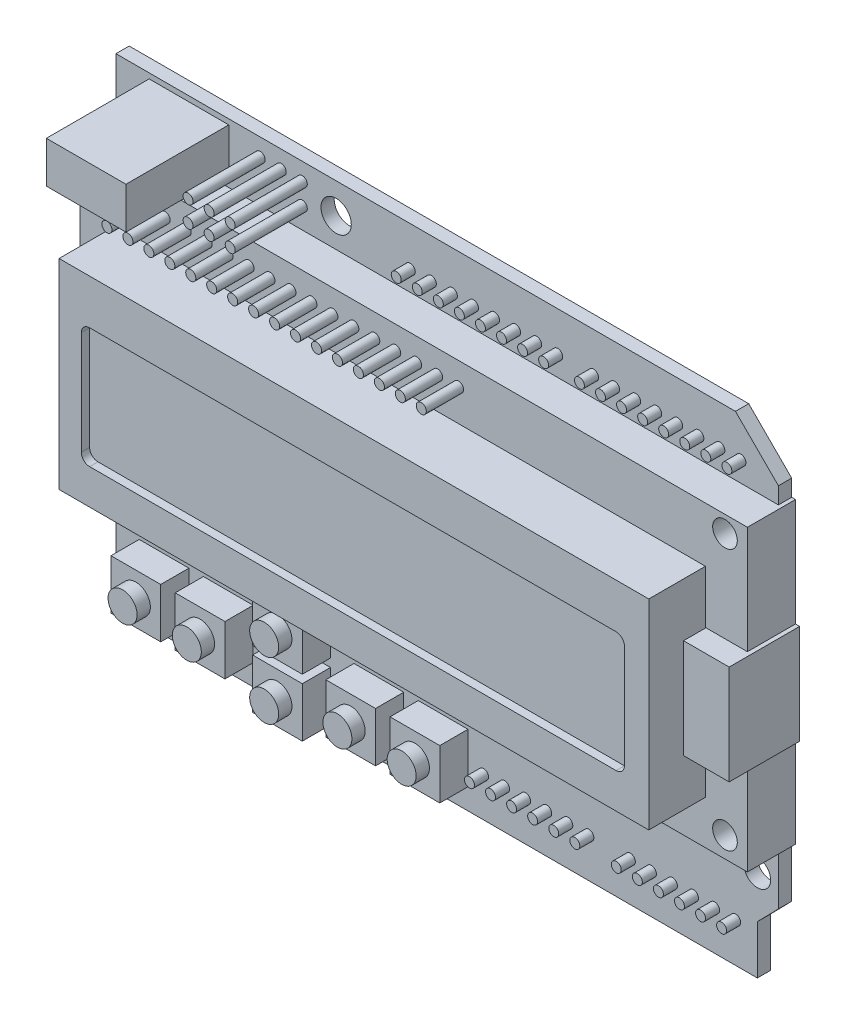
SolidWorks part; units mm, degrees
ref_plane "Front Plane" through (0, 0, 0) normal (0, 0, 1) x (1, 0, 0)
ref_plane "Top Plane" through (0, 0, 0) normal (0, 1, 0) x (1, 0, 0)
ref_plane "Right Plane" through (0, 0, 0) normal (1, 0, 0) x (0, 0, -1)
sketch "Sketch1" plane through (0, 0, 0) normal (0, 0, 1) x (1, 0, 0)
  line L0 (74.3712, 57.8612) -> (79.5528, 52.6796)
  line L1 (74.3712, 57.8612) -> (79.5528, 52.6796)
  line L2 (79.5528, 52.6796) -> (79.5528, 8.4836)
  line L3 (79.5528, 52.6796) -> (79.5528, 8.4836)
  line L4 (79.5528, 8.4836) -> (77.0128, 5.8801)
  line L5 (79.5528, 8.4836) -> (77.0128, 5.8801)
  line L6 (77.0128, 5.8801) -> (77.0128, 0)
  line L7 (77.0128, 5.8801) -> (77.0128, 0)
  line L8 (77.0128, 0) -> (-0.3424, 0)
  line L9 (77.0128, 0) -> (-0.3424, 0)
  line L10 (-0.3424, 0) -> (-0.3424, 57.8612)
  line L11 (-0.3424, 0) -> (-0.3424, 57.8612)
  line L12 (-0.3424, 57.8612) -> (74.3712, 57.8612)
  line L13 (-0.3424, 57.8612) -> (74.3712, 57.8612)
  line L14 (6.5141, 37.6773) -> (6.5141, 25.1773)
  line L15 (71.0141, 38.6773) -> (7.5141, 38.6773)
  line L16 (72.0141, 25.1773) -> (72.0141, 37.6773)
  line L17 (71.0141, 24.1773) -> (7.5141, 24.1773)
  line L18 (3.8321, 19.9433) -> (74.9521, 19.9433)
  line L19 (3.8321, 19.9433) -> (74.9521, 19.9433)
  line L20 (74.9521, 19.9433) -> (74.9521, 44.0733)
  line L21 (74.9521, 19.9433) -> (74.9521, 44.0733)
  line L22 (74.9521, 44.0733) -> (3.8321, 44.0733)
  line L23 (74.9521, 44.0733) -> (3.8321, 44.0733)
  line L24 (3.8321, 44.0733) -> (3.8321, 19.9433)
  line L25 (3.8321, 44.0733) -> (3.8321, 19.9433)
  line L26 (6.5141, 37.6773) -> (6.5141, 25.1773)
  line L27 (71.0141, 38.6773) -> (7.5141, 38.6773)
  line L28 (72.0141, 25.1773) -> (72.0141, 37.6773)
  line L29 (71.0141, 24.1773) -> (7.5141, 24.1773)
  line L30 (6.5141, 25.1773) -> (6.5141, 37.6773)
  line L31 (7.5141, 38.6773) -> (71.0141, 38.6773)
  line L32 (72.0141, 37.6773) -> (72.0141, 25.1773)
  line L33 (71.0141, 24.1773) -> (7.5141, 24.1773)
  line L34 (-0.4859, 14.6773) -> (-0.4859, 50.6773)
  line L35 (-0.4859, 14.6773) -> (-0.4859, 50.6773)
  line L36 (-0.4859, 50.6773) -> (80.0141, 50.6773)
  line L37 (-0.4859, 50.6773) -> (80.0141, 50.6773)
  line L38 (80.0141, 50.6773) -> (80.0141, 14.6773)
  line L39 (80.0141, 50.6773) -> (80.0141, 14.6773)
  line L40 (80.0141, 14.6773) -> (-0.4859, 14.6773)
  line L41 (80.0141, 14.6773) -> (-0.4859, 14.6773)
  line L42 (45.4986, 47.6023) -> (45.4986, 48.2523)
  line L43 (45.4986, 48.2523) -> (45.4986, 47.6023)
  line L44 (44.8486, 47.6023) -> (45.4986, 47.6023)
  line L45 (45.4986, 47.6023) -> (44.8486, 47.6023)
  line L46 (44.8486, 48.2523) -> (44.8486, 47.6023)
  line L47 (44.8486, 47.6023) -> (44.8486, 48.2523)
  line L48 (45.4986, 48.2523) -> (44.8486, 48.2523)
  line L49 (44.8486, 48.2523) -> (45.4986, 48.2523)
  line L50 (45.4986, 47.6023) -> (45.4986, 48.2523)
  line L51 (44.8486, 47.6023) -> (45.4986, 47.6023)
  line L52 (44.8486, 48.2523) -> (44.8486, 47.6023)
  line L53 (45.4986, 48.2523) -> (44.8486, 48.2523)
  line L54 (44.8486, 48.2523) -> (45.4986, 48.2523)
  line L55 (44.8486, 47.6023) -> (44.8486, 48.2523)
  line L56 (45.4986, 47.6023) -> (44.8486, 47.6023)
  line L57 (45.4986, 48.2523) -> (45.4986, 47.6023)
  line L58 (45.4986, 48.2523) -> (44.8486, 48.2523)
  line L59 (45.4986, 48.2523) -> (44.8486, 48.2523)
  line L60 (44.8486, 48.2523) -> (44.8486, 47.6023)
  line L61 (44.8486, 48.2523) -> (44.8486, 47.6023)
  line L62 (45.4986, 47.6023) -> (44.8486, 47.6023)
  line L63 (45.4986, 47.6023) -> (44.8486, 47.6023)
  line L64 (45.4986, 48.2523) -> (45.4986, 47.6023)
  line L65 (45.4986, 48.2523) -> (45.4986, 47.6023)
  line L66 (42.9713, 47.6023) -> (42.9713, 48.2523)
  line L67 (42.9713, 48.2523) -> (42.9713, 47.6023)
  line L68 (42.3213, 47.6023) -> (42.9713, 47.6023)
  line L69 (42.9713, 47.6023) -> (42.3213, 47.6023)
  line L70 (42.3213, 48.2523) -> (42.3213, 47.6023)
  line L71 (42.3213, 47.6023) -> (42.3213, 48.2523)
  line L72 (42.9713, 48.2523) -> (42.3213, 48.2523)
  line L73 (42.3213, 48.2523) -> (42.9713, 48.2523)
  line L74 (42.9713, 47.6023) -> (42.9713, 48.2523)
  line L75 (42.3213, 47.6023) -> (42.9713, 47.6023)
  line L76 (42.3213, 48.2523) -> (42.3213, 47.6023)
  line L77 (42.9713, 48.2523) -> (42.3213, 48.2523)
  line L78 (42.3213, 48.2523) -> (42.9713, 48.2523)
  line L79 (42.3213, 47.6023) -> (42.3213, 48.2523)
  line L80 (42.9713, 47.6023) -> (42.3213, 47.6023)
  line L81 (42.9713, 48.2523) -> (42.9713, 47.6023)
  line L82 (42.9713, 48.2523) -> (42.3213, 48.2523)
  line L83 (42.9713, 48.2523) -> (42.3213, 48.2523)
  line L84 (42.3213, 48.2523) -> (42.3213, 47.6023)
  line L85 (42.3213, 48.2523) -> (42.3213, 47.6023)
  line L86 (42.9713, 47.6023) -> (42.3213, 47.6023)
  line L87 (42.9713, 47.6023) -> (42.3213, 47.6023)
  line L88 (42.9713, 48.2523) -> (42.9713, 47.6023)
  line L89 (42.9713, 48.2523) -> (42.9713, 47.6023)
  line L90 (40.444, 47.6023) -> (40.444, 48.2523)
  line L91 (40.444, 48.2523) -> (40.444, 47.6023)
  line L92 (39.794, 47.6023) -> (40.444, 47.6023)
  line L93 (40.444, 47.6023) -> (39.794, 47.6023)
  line L94 (39.794, 48.2523) -> (39.794, 47.6023)
  line L95 (39.794, 47.6023) -> (39.794, 48.2523)
  line L96 (40.444, 48.2523) -> (39.794, 48.2523)
  line L97 (39.794, 48.2523) -> (40.444, 48.2523)
  line L98 (40.444, 47.6023) -> (40.444, 48.2523)
  line L99 (39.794, 47.6023) -> (40.444, 47.6023)
  line L100 (39.794, 48.2523) -> (39.794, 47.6023)
  line L101 (40.444, 48.2523) -> (39.794, 48.2523)
  line L102 (39.794, 48.2523) -> (40.444, 48.2523)
  line L103 (39.794, 47.6023) -> (39.794, 48.2523)
  line L104 (40.444, 47.6023) -> (39.794, 47.6023)
  line L105 (40.444, 48.2523) -> (40.444, 47.6023)
  line L106 (40.444, 48.2523) -> (39.794, 48.2523)
  line L107 (40.444, 48.2523) -> (39.794, 48.2523)
  line L108 (39.794, 48.2523) -> (39.794, 47.6023)
  line L109 (39.794, 48.2523) -> (39.794, 47.6023)
  line L110 (40.444, 47.6023) -> (39.794, 47.6023)
  line L111 (40.444, 47.6023) -> (39.794, 47.6023)
  line L112 (40.444, 48.2523) -> (40.444, 47.6023)
  line L113 (40.444, 48.2523) -> (40.444, 47.6023)
  line L114 (37.9167, 47.6023) -> (37.9167, 48.2523)
  line L115 (37.9167, 48.2523) -> (37.9167, 47.6023)
  line L116 (37.2667, 47.6023) -> (37.9167, 47.6023)
  line L117 (37.9167, 47.6023) -> (37.2667, 47.6023)
  line L118 (37.2667, 48.2523) -> (37.2667, 47.6023)
  line L119 (37.2667, 47.6023) -> (37.2667, 48.2523)
  line L120 (37.9167, 48.2523) -> (37.2667, 48.2523)
  line L121 (37.2667, 48.2523) -> (37.9167, 48.2523)
  line L122 (37.9167, 47.6023) -> (37.9167, 48.2523)
  line L123 (37.2667, 47.6023) -> (37.9167, 47.6023)
  line L124 (37.2667, 48.2523) -> (37.2667, 47.6023)
  line L125 (37.9167, 48.2523) -> (37.2667, 48.2523)
  line L126 (37.2667, 48.2523) -> (37.9167, 48.2523)
  line L127 (37.2667, 47.6023) -> (37.2667, 48.2523)
  line L128 (37.9167, 47.6023) -> (37.2667, 47.6023)
  line L129 (37.9167, 48.2523) -> (37.9167, 47.6023)
  line L130 (37.9167, 48.2523) -> (37.2667, 48.2523)
  line L131 (37.9167, 48.2523) -> (37.2667, 48.2523)
  line L132 (37.2667, 48.2523) -> (37.2667, 47.6023)
  line L133 (37.2667, 48.2523) -> (37.2667, 47.6023)
  line L134 (37.9167, 47.6023) -> (37.2667, 47.6023)
  line L135 (37.9167, 47.6023) -> (37.2667, 47.6023)
  line L136 (37.9167, 48.2523) -> (37.9167, 47.6023)
  line L137 (37.9167, 48.2523) -> (37.9167, 47.6023)
  line L138 (35.3894, 47.6023) -> (35.3894, 48.2523)
  line L139 (35.3894, 48.2523) -> (35.3894, 47.6023)
  line L140 (34.7394, 47.6023) -> (35.3894, 47.6023)
  line L141 (35.3894, 47.6023) -> (34.7394, 47.6023)
  line L142 (34.7394, 48.2523) -> (34.7394, 47.6023)
  line L143 (34.7394, 47.6023) -> (34.7394, 48.2523)
  line L144 (35.3894, 48.2523) -> (34.7394, 48.2523)
  line L145 (34.7394, 48.2523) -> (35.3894, 48.2523)
  line L146 (35.3894, 47.6023) -> (35.3894, 48.2523)
  line L147 (34.7394, 47.6023) -> (35.3894, 47.6023)
  line L148 (34.7394, 48.2523) -> (34.7394, 47.6023)
  line L149 (35.3894, 48.2523) -> (34.7394, 48.2523)
  line L150 (34.7394, 48.2523) -> (35.3894, 48.2523)
  line L151 (34.7394, 47.6023) -> (34.7394, 48.2523)
  line L152 (35.3894, 47.6023) -> (34.7394, 47.6023)
  line L153 (35.3894, 48.2523) -> (35.3894, 47.6023)
  line L154 (35.3894, 48.2523) -> (34.7394, 48.2523)
  line L155 (35.3894, 48.2523) -> (34.7394, 48.2523)
  line L156 (34.7394, 48.2523) -> (34.7394, 47.6023)
  line L157 (34.7394, 48.2523) -> (34.7394, 47.6023)
  line L158 (35.3894, 47.6023) -> (34.7394, 47.6023)
  line L159 (35.3894, 47.6023) -> (34.7394, 47.6023)
  line L160 (35.3894, 48.2523) -> (35.3894, 47.6023)
  line L161 (35.3894, 48.2523) -> (35.3894, 47.6023)
  line L162 (32.8621, 47.6023) -> (32.8621, 48.2523)
  line L163 (32.8621, 48.2523) -> (32.8621, 47.6023)
  line L164 (32.2121, 47.6023) -> (32.8621, 47.6023)
  line L165 (32.8621, 47.6023) -> (32.2121, 47.6023)
  line L166 (32.2121, 48.2523) -> (32.2121, 47.6023)
  line L167 (32.2121, 47.6023) -> (32.2121, 48.2523)
  line L168 (32.8621, 48.2523) -> (32.2121, 48.2523)
  line L169 (32.2121, 48.2523) -> (32.8621, 48.2523)
  line L170 (32.8621, 47.6023) -> (32.8621, 48.2523)
  line L171 (32.2121, 47.6023) -> (32.8621, 47.6023)
  line L172 (32.2121, 48.2523) -> (32.2121, 47.6023)
  line L173 (32.8621, 48.2523) -> (32.2121, 48.2523)
  line L174 (32.2121, 48.2523) -> (32.8621, 48.2523)
  line L175 (32.2121, 47.6023) -> (32.2121, 48.2523)
  line L176 (32.8621, 47.6023) -> (32.2121, 47.6023)
  line L177 (32.8621, 48.2523) -> (32.8621, 47.6023)
  line L178 (32.8621, 48.2523) -> (32.2121, 48.2523)
  line L179 (32.8621, 48.2523) -> (32.2121, 48.2523)
  line L180 (32.2121, 48.2523) -> (32.2121, 47.6023)
  line L181 (32.2121, 48.2523) -> (32.2121, 47.6023)
  line L182 (32.8621, 47.6023) -> (32.2121, 47.6023)
  line L183 (32.8621, 47.6023) -> (32.2121, 47.6023)
  line L184 (32.8621, 48.2523) -> (32.8621, 47.6023)
  line L185 (32.8621, 48.2523) -> (32.8621, 47.6023)
  line L186 (30.3348, 47.6023) -> (30.3348, 48.2523)
  line L187 (30.3348, 48.2523) -> (30.3348, 47.6023)
  line L188 (29.6848, 47.6023) -> (30.3348, 47.6023)
  line L189 (30.3348, 47.6023) -> (29.6848, 47.6023)
  line L190 (29.6848, 48.2523) -> (29.6848, 47.6023)
  line L191 (29.6848, 47.6023) -> (29.6848, 48.2523)
  line L192 (30.3348, 48.2523) -> (29.6848, 48.2523)
  line L193 (29.6848, 48.2523) -> (30.3348, 48.2523)
  line L194 (30.3348, 47.6023) -> (30.3348, 48.2523)
  line L195 (29.6848, 47.6023) -> (30.3348, 47.6023)
  line L196 (29.6848, 48.2523) -> (29.6848, 47.6023)
  line L197 (30.3348, 48.2523) -> (29.6848, 48.2523)
  line L198 (29.6848, 48.2523) -> (30.3348, 48.2523)
  line L199 (29.6848, 47.6023) -> (29.6848, 48.2523)
  line L200 (30.3348, 47.6023) -> (29.6848, 47.6023)
  line L201 (30.3348, 48.2523) -> (30.3348, 47.6023)
  line L202 (30.3348, 48.2523) -> (29.6848, 48.2523)
  line L203 (30.3348, 48.2523) -> (29.6848, 48.2523)
  line L204 (29.6848, 48.2523) -> (29.6848, 47.6023)
  line L205 (29.6848, 48.2523) -> (29.6848, 47.6023)
  line L206 (30.3348, 47.6023) -> (29.6848, 47.6023)
  line L207 (30.3348, 47.6023) -> (29.6848, 47.6023)
  line L208 (30.3348, 48.2523) -> (30.3348, 47.6023)
  line L209 (30.3348, 48.2523) -> (30.3348, 47.6023)
  line L210 (27.8075, 47.6023) -> (27.8075, 48.2523)
  line L211 (27.8075, 48.2523) -> (27.8075, 47.6023)
  line L212 (27.1575, 47.6023) -> (27.8075, 47.6023)
  line L213 (27.8075, 47.6023) -> (27.1575, 47.6023)
  line L214 (27.1575, 48.2523) -> (27.1575, 47.6023)
  line L215 (27.1575, 47.6023) -> (27.1575, 48.2523)
  line L216 (27.8075, 48.2523) -> (27.1575, 48.2523)
  line L217 (27.1575, 48.2523) -> (27.8075, 48.2523)
  line L218 (27.8075, 47.6023) -> (27.8075, 48.2523)
  line L219 (27.1575, 47.6023) -> (27.8075, 47.6023)
  line L220 (27.1575, 48.2523) -> (27.1575, 47.6023)
  line L221 (27.8075, 48.2523) -> (27.1575, 48.2523)
  line L222 (27.1575, 48.2523) -> (27.8075, 48.2523)
  line L223 (27.1575, 47.6023) -> (27.1575, 48.2523)
  line L224 (27.8075, 47.6023) -> (27.1575, 47.6023)
  line L225 (27.8075, 48.2523) -> (27.8075, 47.6023)
  line L226 (27.8075, 48.2523) -> (27.1575, 48.2523)
  line L227 (27.8075, 48.2523) -> (27.1575, 48.2523)
  line L228 (27.1575, 48.2523) -> (27.1575, 47.6023)
  line L229 (27.1575, 48.2523) -> (27.1575, 47.6023)
  line L230 (27.8075, 47.6023) -> (27.1575, 47.6023)
  line L231 (27.8075, 47.6023) -> (27.1575, 47.6023)
  line L232 (27.8075, 48.2523) -> (27.8075, 47.6023)
  line L233 (27.8075, 48.2523) -> (27.8075, 47.6023)
  line L234 (25.2802, 47.6023) -> (25.2802, 48.2523)
  line L235 (25.2802, 48.2523) -> (25.2802, 47.6023)
  line L236 (24.6302, 47.6023) -> (25.2802, 47.6023)
  line L237 (25.2802, 47.6023) -> (24.6302, 47.6023)
  line L238 (24.6302, 48.2523) -> (24.6302, 47.6023)
  line L239 (24.6302, 47.6023) -> (24.6302, 48.2523)
  line L240 (25.2802, 48.2523) -> (24.6302, 48.2523)
  line L241 (24.6302, 48.2523) -> (25.2802, 48.2523)
  line L242 (25.2802, 47.6023) -> (25.2802, 48.2523)
  line L243 (24.6302, 47.6023) -> (25.2802, 47.6023)
  line L244 (24.6302, 48.2523) -> (24.6302, 47.6023)
  line L245 (25.2802, 48.2523) -> (24.6302, 48.2523)
  line L246 (24.6302, 48.2523) -> (25.2802, 48.2523)
  line L247 (24.6302, 47.6023) -> (24.6302, 48.2523)
  line L248 (25.2802, 47.6023) -> (24.6302, 47.6023)
  line L249 (25.2802, 48.2523) -> (25.2802, 47.6023)
  line L250 (25.2802, 48.2523) -> (24.6302, 48.2523)
  line L251 (25.2802, 48.2523) -> (24.6302, 48.2523)
  line L252 (24.6302, 48.2523) -> (24.6302, 47.6023)
  line L253 (24.6302, 48.2523) -> (24.6302, 47.6023)
  line L254 (25.2802, 47.6023) -> (24.6302, 47.6023)
  line L255 (25.2802, 47.6023) -> (24.6302, 47.6023)
  line L256 (25.2802, 48.2523) -> (25.2802, 47.6023)
  line L257 (25.2802, 48.2523) -> (25.2802, 47.6023)
  line L258 (22.7529, 47.6023) -> (22.7529, 48.2523)
  line L259 (22.7529, 48.2523) -> (22.7529, 47.6023)
  line L260 (22.1029, 47.6023) -> (22.7529, 47.6023)
  line L261 (22.7529, 47.6023) -> (22.1029, 47.6023)
  line L262 (22.1029, 48.2523) -> (22.1029, 47.6023)
  line L263 (22.1029, 47.6023) -> (22.1029, 48.2523)
  line L264 (22.7529, 48.2523) -> (22.1029, 48.2523)
  line L265 (22.1029, 48.2523) -> (22.7529, 48.2523)
  line L266 (22.7529, 47.6023) -> (22.7529, 48.2523)
  line L267 (22.1029, 47.6023) -> (22.7529, 47.6023)
  line L268 (22.1029, 48.2523) -> (22.1029, 47.6023)
  line L269 (22.7529, 48.2523) -> (22.1029, 48.2523)
  line L270 (22.1029, 48.2523) -> (22.7529, 48.2523)
  line L271 (22.1029, 47.6023) -> (22.1029, 48.2523)
  line L272 (22.7529, 47.6023) -> (22.1029, 47.6023)
  line L273 (22.7529, 48.2523) -> (22.7529, 47.6023)
  line L274 (22.7529, 48.2523) -> (22.1029, 48.2523)
  line L275 (22.7529, 48.2523) -> (22.1029, 48.2523)
  line L276 (22.1029, 48.2523) -> (22.1029, 47.6023)
  line L277 (22.1029, 48.2523) -> (22.1029, 47.6023)
  line L278 (22.7529, 47.6023) -> (22.1029, 47.6023)
  line L279 (22.7529, 47.6023) -> (22.1029, 47.6023)
  line L280 (22.7529, 48.2523) -> (22.7529, 47.6023)
  line L281 (22.7529, 48.2523) -> (22.7529, 47.6023)
  line L282 (20.2256, 47.6023) -> (20.2256, 48.2523)
  line L283 (20.2256, 48.2523) -> (20.2256, 47.6023)
  line L284 (19.5756, 47.6023) -> (20.2256, 47.6023)
  line L285 (20.2256, 47.6023) -> (19.5756, 47.6023)
  line L286 (19.5756, 48.2523) -> (19.5756, 47.6023)
  line L287 (19.5756, 47.6023) -> (19.5756, 48.2523)
  line L288 (20.2256, 48.2523) -> (19.5756, 48.2523)
  line L289 (19.5756, 48.2523) -> (20.2256, 48.2523)
  line L290 (20.2256, 47.6023) -> (20.2256, 48.2523)
  line L291 (19.5756, 47.6023) -> (20.2256, 47.6023)
  line L292 (19.5756, 48.2523) -> (19.5756, 47.6023)
  line L293 (20.2256, 48.2523) -> (19.5756, 48.2523)
  line L294 (19.5756, 48.2523) -> (20.2256, 48.2523)
  line L295 (19.5756, 47.6023) -> (19.5756, 48.2523)
  line L296 (20.2256, 47.6023) -> (19.5756, 47.6023)
  line L297 (20.2256, 48.2523) -> (20.2256, 47.6023)
  line L298 (20.2256, 48.2523) -> (19.5756, 48.2523)
  line L299 (20.2256, 48.2523) -> (19.5756, 48.2523)
  line L300 (19.5756, 48.2523) -> (19.5756, 47.6023)
  line L301 (19.5756, 48.2523) -> (19.5756, 47.6023)
  line L302 (20.2256, 47.6023) -> (19.5756, 47.6023)
  line L303 (20.2256, 47.6023) -> (19.5756, 47.6023)
  line L304 (20.2256, 48.2523) -> (20.2256, 47.6023)
  line L305 (20.2256, 48.2523) -> (20.2256, 47.6023)
  line L306 (17.6983, 47.6023) -> (17.6983, 48.2523)
  line L307 (17.6983, 48.2523) -> (17.6983, 47.6023)
  line L308 (17.0483, 47.6023) -> (17.6983, 47.6023)
  line L309 (17.6983, 47.6023) -> (17.0483, 47.6023)
  line L310 (17.0483, 48.2523) -> (17.0483, 47.6023)
  line L311 (17.0483, 47.6023) -> (17.0483, 48.2523)
  line L312 (17.6983, 48.2523) -> (17.0483, 48.2523)
  line L313 (17.0483, 48.2523) -> (17.6983, 48.2523)
  line L314 (17.6983, 47.6023) -> (17.6983, 48.2523)
  line L315 (17.0483, 47.6023) -> (17.6983, 47.6023)
  line L316 (17.0483, 48.2523) -> (17.0483, 47.6023)
  line L317 (17.6983, 48.2523) -> (17.0483, 48.2523)
  line L318 (17.0483, 48.2523) -> (17.6983, 48.2523)
  line L319 (17.0483, 47.6023) -> (17.0483, 48.2523)
  line L320 (17.6983, 47.6023) -> (17.0483, 47.6023)
  line L321 (17.6983, 48.2523) -> (17.6983, 47.6023)
  line L322 (17.6983, 48.2523) -> (17.0483, 48.2523)
  line L323 (17.6983, 48.2523) -> (17.0483, 48.2523)
  line L324 (17.0483, 48.2523) -> (17.0483, 47.6023)
  line L325 (17.0483, 48.2523) -> (17.0483, 47.6023)
  line L326 (17.6983, 47.6023) -> (17.0483, 47.6023)
  line L327 (17.6983, 47.6023) -> (17.0483, 47.6023)
  line L328 (17.6983, 48.2523) -> (17.6983, 47.6023)
  line L329 (17.6983, 48.2523) -> (17.6983, 47.6023)
  line L330 (15.171, 47.6023) -> (15.171, 48.2523)
  line L331 (15.171, 48.2523) -> (15.171, 47.6023)
  line L332 (14.521, 47.6023) -> (15.171, 47.6023)
  line L333 (15.171, 47.6023) -> (14.521, 47.6023)
  line L334 (14.521, 48.2523) -> (14.521, 47.6023)
  line L335 (14.521, 47.6023) -> (14.521, 48.2523)
  line L336 (15.171, 48.2523) -> (14.521, 48.2523)
  line L337 (14.521, 48.2523) -> (15.171, 48.2523)
  line L338 (15.171, 47.6023) -> (15.171, 48.2523)
  line L339 (14.521, 47.6023) -> (15.171, 47.6023)
  line L340 (14.521, 48.2523) -> (14.521, 47.6023)
  line L341 (15.171, 48.2523) -> (14.521, 48.2523)
  line L342 (14.521, 48.2523) -> (15.171, 48.2523)
  line L343 (14.521, 47.6023) -> (14.521, 48.2523)
  line L344 (15.171, 47.6023) -> (14.521, 47.6023)
  line L345 (15.171, 48.2523) -> (15.171, 47.6023)
  line L346 (15.171, 48.2523) -> (14.521, 48.2523)
  line L347 (15.171, 48.2523) -> (14.521, 48.2523)
  line L348 (14.521, 48.2523) -> (14.521, 47.6023)
  line L349 (14.521, 48.2523) -> (14.521, 47.6023)
  line L350 (15.171, 47.6023) -> (14.521, 47.6023)
  line L351 (15.171, 47.6023) -> (14.521, 47.6023)
  line L352 (15.171, 48.2523) -> (15.171, 47.6023)
  line L353 (15.171, 48.2523) -> (15.171, 47.6023)
  line L354 (12.6437, 47.6023) -> (12.6437, 48.2523)
  line L355 (12.6437, 48.2523) -> (12.6437, 47.6023)
  line L356 (11.9937, 47.6023) -> (12.6437, 47.6023)
  line L357 (12.6437, 47.6023) -> (11.9937, 47.6023)
  line L358 (11.9937, 48.2523) -> (11.9937, 47.6023)
  line L359 (11.9937, 47.6023) -> (11.9937, 48.2523)
  line L360 (12.6437, 48.2523) -> (11.9937, 48.2523)
  line L361 (11.9937, 48.2523) -> (12.6437, 48.2523)
  line L362 (12.6437, 47.6023) -> (12.6437, 48.2523)
  line L363 (11.9937, 47.6023) -> (12.6437, 47.6023)
  line L364 (11.9937, 48.2523) -> (11.9937, 47.6023)
  line L365 (12.6437, 48.2523) -> (11.9937, 48.2523)
  line L366 (11.9937, 48.2523) -> (12.6437, 48.2523)
  line L367 (11.9937, 47.6023) -> (11.9937, 48.2523)
  line L368 (12.6437, 47.6023) -> (11.9937, 47.6023)
  line L369 (12.6437, 48.2523) -> (12.6437, 47.6023)
  line L370 (12.6437, 48.2523) -> (11.9937, 48.2523)
  line L371 (12.6437, 48.2523) -> (11.9937, 48.2523)
  line L372 (11.9937, 48.2523) -> (11.9937, 47.6023)
  line L373 (11.9937, 48.2523) -> (11.9937, 47.6023)
  line L374 (12.6437, 47.6023) -> (11.9937, 47.6023)
  line L375 (12.6437, 47.6023) -> (11.9937, 47.6023)
  line L376 (12.6437, 48.2523) -> (12.6437, 47.6023)
  line L377 (12.6437, 48.2523) -> (12.6437, 47.6023)
  line L378 (10.1164, 47.6023) -> (10.1164, 48.2523)
  line L379 (10.1164, 48.2523) -> (10.1164, 47.6023)
  line L380 (9.4664, 47.6023) -> (10.1164, 47.6023)
  line L381 (10.1164, 47.6023) -> (9.4664, 47.6023)
  line L382 (9.4664, 48.2523) -> (9.4664, 47.6023)
  line L383 (9.4664, 47.6023) -> (9.4664, 48.2523)
  line L384 (10.1164, 48.2523) -> (9.4664, 48.2523)
  line L385 (9.4664, 48.2523) -> (10.1164, 48.2523)
  line L386 (10.1164, 47.6023) -> (10.1164, 48.2523)
  line L387 (9.4664, 47.6023) -> (10.1164, 47.6023)
  line L388 (9.4664, 48.2523) -> (9.4664, 47.6023)
  line L389 (10.1164, 48.2523) -> (9.4664, 48.2523)
  line L390 (9.4664, 48.2523) -> (10.1164, 48.2523)
  line L391 (9.4664, 47.6023) -> (9.4664, 48.2523)
  line L392 (10.1164, 47.6023) -> (9.4664, 47.6023)
  line L393 (10.1164, 48.2523) -> (10.1164, 47.6023)
  line L394 (10.1164, 48.2523) -> (9.4664, 48.2523)
  line L395 (10.1164, 48.2523) -> (9.4664, 48.2523)
  line L396 (9.4664, 48.2523) -> (9.4664, 47.6023)
  line L397 (9.4664, 48.2523) -> (9.4664, 47.6023)
  line L398 (10.1164, 47.6023) -> (9.4664, 47.6023)
  line L399 (10.1164, 47.6023) -> (9.4664, 47.6023)
  line L400 (10.1164, 48.2523) -> (10.1164, 47.6023)
  line L401 (10.1164, 48.2523) -> (10.1164, 47.6023)
  line L402 (7.5891, 48.2523) -> (6.9391, 48.2523)
  line L403 (6.9391, 48.2523) -> (7.5891, 48.2523)
  line L404 (6.9391, 48.2523) -> (6.9391, 47.6023)
  line L405 (6.9391, 47.6023) -> (6.9391, 48.2523)
  line L406 (6.9391, 47.6023) -> (7.5891, 47.6023)
  line L407 (7.5891, 47.6023) -> (6.9391, 47.6023)
  line L408 (7.5891, 47.6023) -> (7.5891, 48.2523)
  line L409 (7.5891, 48.2523) -> (7.5891, 47.6023)
  line L410 (7.5891, 48.2523) -> (6.9391, 48.2523)
  line L411 (6.9391, 48.2523) -> (6.9391, 47.6023)
  line L412 (6.9391, 47.6023) -> (7.5891, 47.6023)
  line L413 (7.5891, 47.6023) -> (7.5891, 48.2523)
  line L414 (7.5891, 48.2523) -> (7.5891, 47.6023)
  line L415 (7.5891, 47.6023) -> (6.9391, 47.6023)
  line L416 (6.9391, 47.6023) -> (6.9391, 48.2523)
  line L417 (6.9391, 48.2523) -> (7.5891, 48.2523)
  line L418 (7.5891, 48.2523) -> (7.5891, 47.6023)
  line L419 (7.5891, 48.2523) -> (7.5891, 47.6023)
  line L420 (7.5891, 47.6023) -> (6.9391, 47.6023)
  line L421 (7.5891, 47.6023) -> (6.9391, 47.6023)
  line L422 (6.9391, 48.2523) -> (6.9391, 47.6023)
  line L423 (6.9391, 48.2523) -> (6.9391, 47.6023)
  line L424 (7.5891, 48.2523) -> (6.9391, 48.2523)
  line L425 (7.5891, 48.2523) -> (6.9391, 48.2523)
  line L426 (7.5891, 48.2523) -> (7.5891, 47.6023)
  line L427 (7.5891, 47.6023) -> (6.9391, 47.6023)
  line L428 (6.9391, 47.6023) -> (6.9391, 48.2523)
  line L429 (6.9391, 48.2523) -> (7.5891, 48.2523)
  line L430 (6.9391, 47.9273) -> (7.5891, 47.9273)
  line L431 (7.2641, 48.2523) -> (7.2641, 47.6023)
  line L432 (10.1164, 48.2523) -> (10.1164, 47.6023)
  line L433 (10.1164, 47.6023) -> (9.4664, 47.6023)
  line L434 (9.4664, 47.6023) -> (9.4664, 48.2523)
  line L435 (9.4664, 48.2523) -> (10.1164, 48.2523)
  line L436 (9.4664, 47.9273) -> (10.1164, 47.9273)
  line L437 (9.7914, 48.2523) -> (9.7914, 47.6023)
  line L438 (12.6437, 48.2523) -> (12.6437, 47.6023)
  line L439 (12.6437, 47.6023) -> (11.9937, 47.6023)
  line L440 (11.9937, 47.6023) -> (11.9937, 48.2523)
  line L441 (11.9937, 48.2523) -> (12.6437, 48.2523)
  line L442 (11.9937, 47.9273) -> (12.6437, 47.9273)
  line L443 (12.3187, 48.2523) -> (12.3187, 47.6023)
  line L444 (15.171, 48.2523) -> (15.171, 47.6023)
  line L445 (15.171, 47.6023) -> (14.521, 47.6023)
  line L446 (14.521, 47.6023) -> (14.521, 48.2523)
  line L447 (14.521, 48.2523) -> (15.171, 48.2523)
  line L448 (14.521, 47.9273) -> (15.171, 47.9273)
  line L449 (14.846, 48.2523) -> (14.846, 47.6023)
  line L450 (17.6983, 48.2523) -> (17.6983, 47.6023)
  line L451 (17.6983, 47.6023) -> (17.0483, 47.6023)
  line L452 (17.0483, 47.6023) -> (17.0483, 48.2523)
  line L453 (17.0483, 48.2523) -> (17.6983, 48.2523)
  line L454 (17.0483, 47.9273) -> (17.6983, 47.9273)
  line L455 (17.3733, 48.2523) -> (17.3733, 47.6023)
  line L456 (20.2256, 48.2523) -> (20.2256, 47.6023)
  line L457 (20.2256, 47.6023) -> (19.5756, 47.6023)
  line L458 (19.5756, 47.6023) -> (19.5756, 48.2523)
  line L459 (19.5756, 48.2523) -> (20.2256, 48.2523)
  line L460 (19.5756, 47.9273) -> (20.2256, 47.9273)
  line L461 (19.9006, 48.2523) -> (19.9006, 47.6023)
  line L462 (22.7529, 48.2523) -> (22.7529, 47.6023)
  line L463 (22.7529, 47.6023) -> (22.1029, 47.6023)
  line L464 (22.1029, 47.6023) -> (22.1029, 48.2523)
  line L465 (22.1029, 48.2523) -> (22.7529, 48.2523)
  line L466 (22.1029, 47.9273) -> (22.7529, 47.9273)
  line L467 (22.4279, 48.2523) -> (22.4279, 47.6023)
  line L468 (25.2802, 48.2523) -> (25.2802, 47.6023)
  line L469 (25.2802, 47.6023) -> (24.6302, 47.6023)
  line L470 (24.6302, 47.6023) -> (24.6302, 48.2523)
  line L471 (24.6302, 48.2523) -> (25.2802, 48.2523)
  line L472 (24.6302, 47.9273) -> (25.2802, 47.9273)
  line L473 (24.9552, 48.2523) -> (24.9552, 47.6023)
  line L474 (27.8075, 48.2523) -> (27.8075, 47.6023)
  line L475 (27.8075, 47.6023) -> (27.1575, 47.6023)
  line L476 (27.1575, 47.6023) -> (27.1575, 48.2523)
  line L477 (27.1575, 48.2523) -> (27.8075, 48.2523)
  line L478 (27.1575, 47.9273) -> (27.8075, 47.9273)
  line L479 (27.4825, 48.2523) -> (27.4825, 47.6023)
  line L480 (30.3348, 48.2523) -> (30.3348, 47.6023)
  line L481 (30.3348, 47.6023) -> (29.6848, 47.6023)
  line L482 (29.6848, 47.6023) -> (29.6848, 48.2523)
  line L483 (29.6848, 48.2523) -> (30.3348, 48.2523)
  line L484 (29.6848, 47.9273) -> (30.3348, 47.9273)
  line L485 (30.0098, 48.2523) -> (30.0098, 47.6023)
  line L486 (32.8621, 48.2523) -> (32.8621, 47.6023)
  line L487 (32.8621, 47.6023) -> (32.2121, 47.6023)
  line L488 (32.2121, 47.6023) -> (32.2121, 48.2523)
  line L489 (32.2121, 48.2523) -> (32.8621, 48.2523)
  line L490 (32.2121, 47.9273) -> (32.8621, 47.9273)
  line L491 (32.5371, 48.2523) -> (32.5371, 47.6023)
  line L492 (35.3894, 48.2523) -> (35.3894, 47.6023)
  line L493 (35.3894, 47.6023) -> (34.7394, 47.6023)
  line L494 (34.7394, 47.6023) -> (34.7394, 48.2523)
  line L495 (34.7394, 48.2523) -> (35.3894, 48.2523)
  line L496 (34.7394, 47.9273) -> (35.3894, 47.9273)
  line L497 (35.0644, 48.2523) -> (35.0644, 47.6023)
  line L498 (37.9167, 48.2523) -> (37.9167, 47.6023)
  line L499 (37.9167, 47.6023) -> (37.2667, 47.6023)
  line L500 (37.2667, 47.6023) -> (37.2667, 48.2523)
  line L501 (37.2667, 48.2523) -> (37.9167, 48.2523)
  line L502 (37.2667, 47.9273) -> (37.9167, 47.9273)
  line L503 (37.5917, 48.2523) -> (37.5917, 47.6023)
  line L504 (40.444, 48.2523) -> (40.444, 47.6023)
  line L505 (40.444, 47.6023) -> (39.794, 47.6023)
  line L506 (39.794, 47.6023) -> (39.794, 48.2523)
  line L507 (39.794, 48.2523) -> (40.444, 48.2523)
  line L508 (39.794, 47.9273) -> (40.444, 47.9273)
  line L509 (40.119, 48.2523) -> (40.119, 47.6023)
  line L510 (42.9713, 48.2523) -> (42.9713, 47.6023)
  line L511 (42.9713, 47.6023) -> (42.3213, 47.6023)
  line L512 (42.3213, 47.6023) -> (42.3213, 48.2523)
  line L513 (42.3213, 48.2523) -> (42.9713, 48.2523)
  line L514 (42.3213, 47.9273) -> (42.9713, 47.9273)
  line L515 (42.6463, 48.2523) -> (42.6463, 47.6023)
  line L516 (45.4986, 48.2523) -> (45.4986, 47.6023)
  line L517 (45.4986, 47.6023) -> (44.8486, 47.6023)
  line L518 (44.8486, 47.6023) -> (44.8486, 48.2523)
  line L519 (44.8486, 48.2523) -> (45.4986, 48.2523)
  line L520 (44.8486, 47.9273) -> (45.4986, 47.9273)
  line L521 (45.1736, 48.2523) -> (45.1736, 47.6023)
  line L522 (43.9236, 47.1773) -> (43.9236, 48.6773)
  line L523 (43.9236, 48.6773) -> (43.9236, 47.1773)
  line L524 (43.9236, 48.6773) -> (43.9236, 47.1773)
  line L525 (44.4236, 49.1773) -> (45.9236, 49.1773)
  line L526 (45.9236, 49.1773) -> (44.4236, 49.1773)
  line L527 (45.9236, 49.1773) -> (44.4236, 49.1773)
  line L528 (45.9236, 46.6773) -> (44.4236, 46.6773)
  line L529 (44.4236, 46.6773) -> (45.9236, 46.6773)
  line L530 (45.9236, 46.6773) -> (44.4236, 46.6773)
  line L531 (44.8486, 47.6023) -> (45.4986, 47.6023)
  line L532 (45.4986, 47.6023) -> (45.4986, 48.2523)
  line L533 (45.4986, 48.2523) -> (44.8486, 48.2523)
  line L534 (44.8486, 48.2523) -> (44.8486, 47.6023)
  line L535 (43.9236, 47.1773) -> (43.9236, 48.6773)
  line L536 (44.4236, 49.1773) -> (45.9236, 49.1773)
  line L537 (45.9236, 46.6773) -> (44.4236, 46.6773)
  line L538 (46.4236, 48.6773) -> (46.4236, 47.1773)
  line L539 (43.9236, 47.9273) -> (44.8486, 47.9273)
  line L540 (45.4986, 47.9273) -> (46.4236, 47.9273)
  line L541 (46.4236, 47.1773) -> (46.4236, 48.6773)
  line L542 (46.4236, 48.6773) -> (46.4236, 47.1773)
  line L543 (46.4236, 47.1773) -> (46.4236, 48.6773)
  line L544 (41.3963, 47.1773) -> (41.3963, 48.6773)
  line L545 (41.3963, 48.6773) -> (41.3963, 47.1773)
  line L546 (41.3963, 48.6773) -> (41.3963, 47.1773)
  line L547 (41.8963, 49.1773) -> (43.3963, 49.1773)
  line L548 (43.3963, 49.1773) -> (41.8963, 49.1773)
  line L549 (43.3963, 49.1773) -> (41.8963, 49.1773)
  line L550 (43.3963, 46.6773) -> (41.8963, 46.6773)
  line L551 (41.8963, 46.6773) -> (43.3963, 46.6773)
  line L552 (43.3963, 46.6773) -> (41.8963, 46.6773)
  line L553 (42.3213, 47.6023) -> (42.9713, 47.6023)
  line L554 (42.9713, 47.6023) -> (42.9713, 48.2523)
  line L555 (42.9713, 48.2523) -> (42.3213, 48.2523)
  line L556 (42.3213, 48.2523) -> (42.3213, 47.6023)
  line L557 (41.3963, 47.1773) -> (41.3963, 48.6773)
  line L558 (41.8963, 49.1773) -> (43.3963, 49.1773)
  line L559 (43.3963, 46.6773) -> (41.8963, 46.6773)
  line L560 (43.8963, 48.6773) -> (43.8963, 47.1773)
  line L561 (41.3963, 47.9273) -> (42.3213, 47.9273)
  line L562 (42.9713, 47.9273) -> (43.8963, 47.9273)
  line L563 (43.8963, 47.1773) -> (43.8963, 48.6773)
  line L564 (43.8963, 48.6773) -> (43.8963, 47.1773)
  line L565 (43.8963, 47.1773) -> (43.8963, 48.6773)
  line L566 (38.869, 47.1773) -> (38.869, 48.6773)
  line L567 (38.869, 48.6773) -> (38.869, 47.1773)
  line L568 (38.869, 48.6773) -> (38.869, 47.1773)
  line L569 (39.369, 49.1773) -> (40.869, 49.1773)
  line L570 (40.869, 49.1773) -> (39.369, 49.1773)
  line L571 (40.869, 49.1773) -> (39.369, 49.1773)
  line L572 (40.869, 46.6773) -> (39.369, 46.6773)
  line L573 (39.369, 46.6773) -> (40.869, 46.6773)
  line L574 (40.869, 46.6773) -> (39.369, 46.6773)
  line L575 (39.794, 47.6023) -> (40.444, 47.6023)
  line L576 (40.444, 47.6023) -> (40.444, 48.2523)
  line L577 (40.444, 48.2523) -> (39.794, 48.2523)
  line L578 (39.794, 48.2523) -> (39.794, 47.6023)
  line L579 (38.869, 47.1773) -> (38.869, 48.6773)
  line L580 (39.369, 49.1773) -> (40.869, 49.1773)
  line L581 (40.869, 46.6773) -> (39.369, 46.6773)
  line L582 (41.369, 48.6773) -> (41.369, 47.1773)
  line L583 (38.869, 47.9273) -> (39.794, 47.9273)
  line L584 (40.444, 47.9273) -> (41.369, 47.9273)
  line L585 (41.369, 47.1773) -> (41.369, 48.6773)
  line L586 (41.369, 48.6773) -> (41.369, 47.1773)
  line L587 (41.369, 47.1773) -> (41.369, 48.6773)
  line L588 (36.3417, 47.1773) -> (36.3417, 48.6773)
  line L589 (36.3417, 48.6773) -> (36.3417, 47.1773)
  line L590 (36.3417, 48.6773) -> (36.3417, 47.1773)
  line L591 (36.8417, 49.1773) -> (38.3417, 49.1773)
  line L592 (38.3417, 49.1773) -> (36.8417, 49.1773)
  line L593 (38.3417, 49.1773) -> (36.8417, 49.1773)
  line L594 (38.3417, 46.6773) -> (36.8417, 46.6773)
  line L595 (36.8417, 46.6773) -> (38.3417, 46.6773)
  line L596 (38.3417, 46.6773) -> (36.8417, 46.6773)
  line L597 (37.2667, 47.6023) -> (37.9167, 47.6023)
  line L598 (37.9167, 47.6023) -> (37.9167, 48.2523)
  line L599 (37.9167, 48.2523) -> (37.2667, 48.2523)
  line L600 (37.2667, 48.2523) -> (37.2667, 47.6023)
  line L601 (36.3417, 47.1773) -> (36.3417, 48.6773)
  line L602 (36.8417, 49.1773) -> (38.3417, 49.1773)
  line L603 (38.3417, 46.6773) -> (36.8417, 46.6773)
  line L604 (38.8417, 48.6773) -> (38.8417, 47.1773)
  line L605 (36.3417, 47.9273) -> (37.2667, 47.9273)
  line L606 (37.9167, 47.9273) -> (38.8417, 47.9273)
  line L607 (38.8417, 47.1773) -> (38.8417, 48.6773)
  line L608 (38.8417, 48.6773) -> (38.8417, 47.1773)
  line L609 (38.8417, 47.1773) -> (38.8417, 48.6773)
  line L610 (33.8144, 47.1773) -> (33.8144, 48.6773)
  line L611 (33.8144, 48.6773) -> (33.8144, 47.1773)
  line L612 (33.8144, 48.6773) -> (33.8144, 47.1773)
  line L613 (34.3144, 49.1773) -> (35.8144, 49.1773)
  line L614 (35.8144, 49.1773) -> (34.3144, 49.1773)
  line L615 (35.8144, 49.1773) -> (34.3144, 49.1773)
  line L616 (35.8144, 46.6773) -> (34.3144, 46.6773)
  line L617 (34.3144, 46.6773) -> (35.8144, 46.6773)
  line L618 (35.8144, 46.6773) -> (34.3144, 46.6773)
  line L619 (34.7394, 47.6023) -> (35.3894, 47.6023)
  line L620 (35.3894, 47.6023) -> (35.3894, 48.2523)
  line L621 (35.3894, 48.2523) -> (34.7394, 48.2523)
  line L622 (34.7394, 48.2523) -> (34.7394, 47.6023)
  line L623 (33.8144, 47.1773) -> (33.8144, 48.6773)
  line L624 (34.3144, 49.1773) -> (35.8144, 49.1773)
  line L625 (35.8144, 46.6773) -> (34.3144, 46.6773)
  line L626 (36.3144, 48.6773) -> (36.3144, 47.1773)
  line L627 (33.8144, 47.9273) -> (34.7394, 47.9273)
  line L628 (35.3894, 47.9273) -> (36.3144, 47.9273)
  line L629 (36.3144, 47.1773) -> (36.3144, 48.6773)
  line L630 (36.3144, 48.6773) -> (36.3144, 47.1773)
  line L631 (36.3144, 47.1773) -> (36.3144, 48.6773)
  line L632 (31.2871, 47.1773) -> (31.2871, 48.6773)
  line L633 (31.2871, 48.6773) -> (31.2871, 47.1773)
  line L634 (31.2871, 48.6773) -> (31.2871, 47.1773)
  line L635 (31.7871, 49.1773) -> (33.2871, 49.1773)
  line L636 (33.2871, 49.1773) -> (31.7871, 49.1773)
  line L637 (33.2871, 49.1773) -> (31.7871, 49.1773)
  line L638 (33.2871, 46.6773) -> (31.7871, 46.6773)
  line L639 (31.7871, 46.6773) -> (33.2871, 46.6773)
  line L640 (33.2871, 46.6773) -> (31.7871, 46.6773)
  line L641 (32.2121, 47.6023) -> (32.8621, 47.6023)
  line L642 (32.8621, 47.6023) -> (32.8621, 48.2523)
  line L643 (32.8621, 48.2523) -> (32.2121, 48.2523)
  line L644 (32.2121, 48.2523) -> (32.2121, 47.6023)
  line L645 (31.2871, 47.1773) -> (31.2871, 48.6773)
  line L646 (31.7871, 49.1773) -> (33.2871, 49.1773)
  line L647 (33.2871, 46.6773) -> (31.7871, 46.6773)
  line L648 (33.7871, 48.6773) -> (33.7871, 47.1773)
  line L649 (31.2871, 47.9273) -> (32.2121, 47.9273)
  line L650 (32.8621, 47.9273) -> (33.7871, 47.9273)
  line L651 (33.7871, 47.1773) -> (33.7871, 48.6773)
  line L652 (33.7871, 48.6773) -> (33.7871, 47.1773)
  line L653 (33.7871, 47.1773) -> (33.7871, 48.6773)
  line L654 (28.7598, 47.1773) -> (28.7598, 48.6773)
  line L655 (28.7598, 48.6773) -> (28.7598, 47.1773)
  line L656 (28.7598, 48.6773) -> (28.7598, 47.1773)
  line L657 (29.2598, 49.1773) -> (30.7598, 49.1773)
  line L658 (30.7598, 49.1773) -> (29.2598, 49.1773)
  line L659 (30.7598, 49.1773) -> (29.2598, 49.1773)
  line L660 (30.7598, 46.6773) -> (29.2598, 46.6773)
  line L661 (29.2598, 46.6773) -> (30.7598, 46.6773)
  line L662 (30.7598, 46.6773) -> (29.2598, 46.6773)
  line L663 (29.6848, 47.6023) -> (30.3348, 47.6023)
  line L664 (30.3348, 47.6023) -> (30.3348, 48.2523)
  line L665 (30.3348, 48.2523) -> (29.6848, 48.2523)
  line L666 (29.6848, 48.2523) -> (29.6848, 47.6023)
  line L667 (28.7598, 47.1773) -> (28.7598, 48.6773)
  line L668 (29.2598, 49.1773) -> (30.7598, 49.1773)
  line L669 (30.7598, 46.6773) -> (29.2598, 46.6773)
  line L670 (31.2598, 48.6773) -> (31.2598, 47.1773)
  line L671 (28.7598, 47.9273) -> (29.6848, 47.9273)
  line L672 (30.3348, 47.9273) -> (31.2598, 47.9273)
  line L673 (31.2598, 47.1773) -> (31.2598, 48.6773)
  line L674 (31.2598, 48.6773) -> (31.2598, 47.1773)
  line L675 (31.2598, 47.1773) -> (31.2598, 48.6773)
  line L676 (26.2325, 47.1773) -> (26.2325, 48.6773)
  line L677 (26.2325, 48.6773) -> (26.2325, 47.1773)
  line L678 (26.2325, 48.6773) -> (26.2325, 47.1773)
  line L679 (26.7325, 49.1773) -> (28.2325, 49.1773)
  line L680 (28.2325, 49.1773) -> (26.7325, 49.1773)
  line L681 (28.2325, 49.1773) -> (26.7325, 49.1773)
  line L682 (28.2325, 46.6773) -> (26.7325, 46.6773)
  line L683 (26.7325, 46.6773) -> (28.2325, 46.6773)
  line L684 (28.2325, 46.6773) -> (26.7325, 46.6773)
  line L685 (27.1575, 47.6023) -> (27.8075, 47.6023)
  line L686 (27.8075, 47.6023) -> (27.8075, 48.2523)
  line L687 (27.8075, 48.2523) -> (27.1575, 48.2523)
  line L688 (27.1575, 48.2523) -> (27.1575, 47.6023)
  line L689 (26.2325, 47.1773) -> (26.2325, 48.6773)
  line L690 (26.7325, 49.1773) -> (28.2325, 49.1773)
  line L691 (28.2325, 46.6773) -> (26.7325, 46.6773)
  line L692 (28.7325, 48.6773) -> (28.7325, 47.1773)
  line L693 (26.2325, 47.9273) -> (27.1575, 47.9273)
  line L694 (27.8075, 47.9273) -> (28.7325, 47.9273)
  line L695 (28.7325, 47.1773) -> (28.7325, 48.6773)
  line L696 (28.7325, 48.6773) -> (28.7325, 47.1773)
  line L697 (28.7325, 47.1773) -> (28.7325, 48.6773)
  line L698 (23.7052, 47.1773) -> (23.7052, 48.6773)
  line L699 (23.7052, 48.6773) -> (23.7052, 47.1773)
  line L700 (23.7052, 48.6773) -> (23.7052, 47.1773)
  line L701 (24.2052, 49.1773) -> (25.7052, 49.1773)
  line L702 (25.7052, 49.1773) -> (24.2052, 49.1773)
  line L703 (25.7052, 49.1773) -> (24.2052, 49.1773)
  line L704 (25.7052, 46.6773) -> (24.2052, 46.6773)
  line L705 (24.2052, 46.6773) -> (25.7052, 46.6773)
  line L706 (25.7052, 46.6773) -> (24.2052, 46.6773)
  line L707 (24.6302, 47.6023) -> (25.2802, 47.6023)
  line L708 (25.2802, 47.6023) -> (25.2802, 48.2523)
  line L709 (25.2802, 48.2523) -> (24.6302, 48.2523)
  line L710 (24.6302, 48.2523) -> (24.6302, 47.6023)
  line L711 (23.7052, 47.1773) -> (23.7052, 48.6773)
  line L712 (24.2052, 49.1773) -> (25.7052, 49.1773)
  line L713 (25.7052, 46.6773) -> (24.2052, 46.6773)
  line L714 (26.2052, 48.6773) -> (26.2052, 47.1773)
  line L715 (23.7052, 47.9273) -> (24.6302, 47.9273)
  line L716 (25.2802, 47.9273) -> (26.2052, 47.9273)
  line L717 (26.2052, 47.1773) -> (26.2052, 48.6773)
  line L718 (26.2052, 48.6773) -> (26.2052, 47.1773)
  line L719 (26.2052, 47.1773) -> (26.2052, 48.6773)
  line L720 (21.1779, 47.1773) -> (21.1779, 48.6773)
  line L721 (21.1779, 48.6773) -> (21.1779, 47.1773)
  line L722 (21.1779, 48.6773) -> (21.1779, 47.1773)
  line L723 (21.6779, 49.1773) -> (23.1779, 49.1773)
  line L724 (23.1779, 49.1773) -> (21.6779, 49.1773)
  line L725 (23.1779, 49.1773) -> (21.6779, 49.1773)
  line L726 (23.1779, 46.6773) -> (21.6779, 46.6773)
  line L727 (21.6779, 46.6773) -> (23.1779, 46.6773)
  line L728 (23.1779, 46.6773) -> (21.6779, 46.6773)
  line L729 (22.1029, 47.6023) -> (22.7529, 47.6023)
  line L730 (22.7529, 47.6023) -> (22.7529, 48.2523)
  line L731 (22.7529, 48.2523) -> (22.1029, 48.2523)
  line L732 (22.1029, 48.2523) -> (22.1029, 47.6023)
  line L733 (21.1779, 47.1773) -> (21.1779, 48.6773)
  line L734 (21.6779, 49.1773) -> (23.1779, 49.1773)
  line L735 (23.1779, 46.6773) -> (21.6779, 46.6773)
  line L736 (23.6779, 48.6773) -> (23.6779, 47.1773)
  line L737 (21.1779, 47.9273) -> (22.1029, 47.9273)
  line L738 (22.7529, 47.9273) -> (23.6779, 47.9273)
  line L739 (23.6779, 47.1773) -> (23.6779, 48.6773)
  line L740 (23.6779, 48.6773) -> (23.6779, 47.1773)
  line L741 (23.6779, 47.1773) -> (23.6779, 48.6773)
  line L742 (18.6506, 47.1773) -> (18.6506, 48.6773)
  line L743 (18.6506, 48.6773) -> (18.6506, 47.1773)
  line L744 (18.6506, 48.6773) -> (18.6506, 47.1773)
  line L745 (19.1506, 49.1773) -> (20.6506, 49.1773)
  line L746 (20.6506, 49.1773) -> (19.1506, 49.1773)
  line L747 (20.6506, 49.1773) -> (19.1506, 49.1773)
  line L748 (20.6506, 46.6773) -> (19.1506, 46.6773)
  line L749 (19.1506, 46.6773) -> (20.6506, 46.6773)
  line L750 (20.6506, 46.6773) -> (19.1506, 46.6773)
  line L751 (19.5756, 47.6023) -> (20.2256, 47.6023)
  line L752 (20.2256, 47.6023) -> (20.2256, 48.2523)
  line L753 (20.2256, 48.2523) -> (19.5756, 48.2523)
  line L754 (19.5756, 48.2523) -> (19.5756, 47.6023)
  line L755 (18.6506, 47.1773) -> (18.6506, 48.6773)
  line L756 (19.1506, 49.1773) -> (20.6506, 49.1773)
  line L757 (20.6506, 46.6773) -> (19.1506, 46.6773)
  line L758 (21.1506, 48.6773) -> (21.1506, 47.1773)
  line L759 (18.6506, 47.9273) -> (19.5756, 47.9273)
  line L760 (20.2256, 47.9273) -> (21.1506, 47.9273)
  line L761 (21.1506, 47.1773) -> (21.1506, 48.6773)
  line L762 (21.1506, 48.6773) -> (21.1506, 47.1773)
  line L763 (21.1506, 47.1773) -> (21.1506, 48.6773)
  line L764 (16.1233, 47.1773) -> (16.1233, 48.6773)
  line L765 (16.1233, 48.6773) -> (16.1233, 47.1773)
  line L766 (16.1233, 48.6773) -> (16.1233, 47.1773)
  line L767 (16.6233, 49.1773) -> (18.1233, 49.1773)
  line L768 (18.1233, 49.1773) -> (16.6233, 49.1773)
  line L769 (18.1233, 49.1773) -> (16.6233, 49.1773)
  line L770 (18.1233, 46.6773) -> (16.6233, 46.6773)
  line L771 (16.6233, 46.6773) -> (18.1233, 46.6773)
  line L772 (18.1233, 46.6773) -> (16.6233, 46.6773)
  line L773 (17.0483, 47.6023) -> (17.6983, 47.6023)
  line L774 (17.6983, 47.6023) -> (17.6983, 48.2523)
  line L775 (17.6983, 48.2523) -> (17.0483, 48.2523)
  line L776 (17.0483, 48.2523) -> (17.0483, 47.6023)
  line L777 (16.1233, 47.1773) -> (16.1233, 48.6773)
  line L778 (16.6233, 49.1773) -> (18.1233, 49.1773)
  line L779 (18.1233, 46.6773) -> (16.6233, 46.6773)
  line L780 (18.6233, 48.6773) -> (18.6233, 47.1773)
  line L781 (16.1233, 47.9273) -> (17.0483, 47.9273)
  line L782 (17.6983, 47.9273) -> (18.6233, 47.9273)
  line L783 (18.6233, 47.1773) -> (18.6233, 48.6773)
  line L784 (18.6233, 48.6773) -> (18.6233, 47.1773)
  line L785 (18.6233, 47.1773) -> (18.6233, 48.6773)
  line L786 (13.596, 47.1773) -> (13.596, 48.6773)
  line L787 (13.596, 48.6773) -> (13.596, 47.1773)
  line L788 (13.596, 48.6773) -> (13.596, 47.1773)
  line L789 (14.096, 49.1773) -> (15.596, 49.1773)
  line L790 (15.596, 49.1773) -> (14.096, 49.1773)
  line L791 (15.596, 49.1773) -> (14.096, 49.1773)
  line L792 (15.596, 46.6773) -> (14.096, 46.6773)
  line L793 (14.096, 46.6773) -> (15.596, 46.6773)
  line L794 (15.596, 46.6773) -> (14.096, 46.6773)
  line L795 (14.521, 47.6023) -> (15.171, 47.6023)
  line L796 (15.171, 47.6023) -> (15.171, 48.2523)
  line L797 (15.171, 48.2523) -> (14.521, 48.2523)
  line L798 (14.521, 48.2523) -> (14.521, 47.6023)
  line L799 (13.596, 47.1773) -> (13.596, 48.6773)
  line L800 (14.096, 49.1773) -> (15.596, 49.1773)
  line L801 (15.596, 46.6773) -> (14.096, 46.6773)
  line L802 (16.096, 48.6773) -> (16.096, 47.1773)
  line L803 (13.596, 47.9273) -> (14.521, 47.9273)
  line L804 (15.171, 47.9273) -> (16.096, 47.9273)
  line L805 (16.096, 47.1773) -> (16.096, 48.6773)
  line L806 (16.096, 48.6773) -> (16.096, 47.1773)
  line L807 (16.096, 47.1773) -> (16.096, 48.6773)
  line L808 (11.0687, 47.1773) -> (11.0687, 48.6773)
  line L809 (11.0687, 48.6773) -> (11.0687, 47.1773)
  line L810 (11.0687, 48.6773) -> (11.0687, 47.1773)
  line L811 (11.5687, 49.1773) -> (13.0687, 49.1773)
  line L812 (13.0687, 49.1773) -> (11.5687, 49.1773)
  line L813 (13.0687, 49.1773) -> (11.5687, 49.1773)
  line L814 (13.0687, 46.6773) -> (11.5687, 46.6773)
  line L815 (11.5687, 46.6773) -> (13.0687, 46.6773)
  line L816 (13.0687, 46.6773) -> (11.5687, 46.6773)
  line L817 (11.9937, 47.6023) -> (12.6437, 47.6023)
  line L818 (12.6437, 47.6023) -> (12.6437, 48.2523)
  line L819 (12.6437, 48.2523) -> (11.9937, 48.2523)
  line L820 (11.9937, 48.2523) -> (11.9937, 47.6023)
  line L821 (11.0687, 47.1773) -> (11.0687, 48.6773)
  line L822 (11.5687, 49.1773) -> (13.0687, 49.1773)
  line L823 (13.0687, 46.6773) -> (11.5687, 46.6773)
  line L824 (13.5687, 48.6773) -> (13.5687, 47.1773)
  line L825 (11.0687, 47.9273) -> (11.9937, 47.9273)
  line L826 (12.6437, 47.9273) -> (13.5687, 47.9273)
  line L827 (13.5687, 47.1773) -> (13.5687, 48.6773)
  line L828 (13.5687, 48.6773) -> (13.5687, 47.1773)
  line L829 (13.5687, 47.1773) -> (13.5687, 48.6773)
  line L830 (8.5414, 47.1773) -> (8.5414, 48.6773)
  line L831 (8.5414, 48.6773) -> (8.5414, 47.1773)
  line L832 (8.5414, 48.6773) -> (8.5414, 47.1773)
  line L833 (9.0414, 49.1773) -> (10.5414, 49.1773)
  line L834 (10.5414, 49.1773) -> (9.0414, 49.1773)
  line L835 (10.5414, 49.1773) -> (9.0414, 49.1773)
  line L836 (10.5414, 46.6773) -> (9.0414, 46.6773)
  line L837 (9.0414, 46.6773) -> (10.5414, 46.6773)
  line L838 (10.5414, 46.6773) -> (9.0414, 46.6773)
  line L839 (9.4664, 47.6023) -> (10.1164, 47.6023)
  line L840 (10.1164, 47.6023) -> (10.1164, 48.2523)
  line L841 (10.1164, 48.2523) -> (9.4664, 48.2523)
  line L842 (9.4664, 48.2523) -> (9.4664, 47.6023)
  line L843 (8.5414, 47.1773) -> (8.5414, 48.6773)
  line L844 (9.0414, 49.1773) -> (10.5414, 49.1773)
  line L845 (10.5414, 46.6773) -> (9.0414, 46.6773)
  line L846 (11.0414, 48.6773) -> (11.0414, 47.1773)
  line L847 (8.5414, 47.9273) -> (9.4664, 47.9273)
  line L848 (10.1164, 47.9273) -> (11.0414, 47.9273)
  line L849 (11.0414, 47.1773) -> (11.0414, 48.6773)
  line L850 (11.0414, 48.6773) -> (11.0414, 47.1773)
  line L851 (11.0414, 47.1773) -> (11.0414, 48.6773)
  line L852 (8.5141, 47.1773) -> (8.5141, 48.6773)
  line L853 (8.5141, 48.6773) -> (8.5141, 47.1773)
  line L854 (8.5141, 47.1773) -> (8.5141, 48.6773)
  line L855 (6.9391, 47.6023) -> (7.5891, 47.6023)
  line L856 (7.5891, 47.6023) -> (7.5891, 48.2523)
  line L857 (7.5891, 48.2523) -> (6.9391, 48.2523)
  line L858 (6.9391, 48.2523) -> (6.9391, 47.6023)
  line L859 (6.0141, 47.1773) -> (6.0141, 48.6773)
  line L860 (6.5141, 49.1773) -> (8.0141, 49.1773)
  line L861 (8.0141, 46.6773) -> (6.5141, 46.6773)
  line L862 (8.5141, 48.6773) -> (8.5141, 47.1773)
  line L863 (6.0141, 47.9273) -> (6.9391, 47.9273)
  line L864 (7.5891, 47.9273) -> (8.5141, 47.9273)
  line L865 (66.6028, 21.1773) -> (71.5141, 22.1773)
  line L866 (66.503, 21.6672) -> (66.6028, 21.1773)
  line L867 (71.4144, 22.6672) -> (66.503, 21.6672)
  line L868 (71.5141, 22.1773) -> (71.4144, 22.6672)
  line L869 (70.2616, 21.9222) -> (67.7556, 21.9222)
  line L870 (69.0086, 21.6671) -> (69.0086, 22.1774)
  line L871 (71.5141, 22.1773) -> (71.4144, 22.6672)
  line L872 (71.5141, 22.1773) -> (71.4144, 22.6672)
  line L873 (71.5141, 22.1773) -> (71.4144, 22.6672)
  line L874 (71.4144, 22.6672) -> (66.503, 21.6672)
  line L875 (71.4144, 22.6672) -> (66.503, 21.6672)
  line L876 (71.4144, 22.6672) -> (66.503, 21.6672)
  line L877 (66.503, 21.6672) -> (66.6028, 21.1773)
  line L878 (66.503, 21.6672) -> (66.6028, 21.1773)
  line L879 (66.503, 21.6672) -> (66.6028, 21.1773)
  line L880 (66.6028, 21.1773) -> (71.5141, 22.1773)
  line L881 (66.6028, 21.1773) -> (71.5141, 22.1773)
  line L882 (66.6028, 21.1773) -> (71.5141, 22.1773)
  line L883 (71.4144, 42.6873) -> (71.5141, 43.1773)
  line L884 (66.503, 43.6873) -> (71.4144, 42.6873)
  line L885 (66.6028, 44.1773) -> (66.503, 43.6873)
  line L886 (71.5141, 43.1773) -> (66.6028, 44.1773)
  line L887 (67.7556, 43.4323) -> (70.2616, 43.4323)
  line L888 (69.0086, 43.1772) -> (69.0086, 43.6874)
  line L889 (71.5141, 43.1773) -> (66.6028, 44.1773)
  line L890 (71.5141, 43.1773) -> (66.6028, 44.1773)
  line L891 (71.5141, 43.1773) -> (66.6028, 44.1773)
  line L892 (66.6028, 44.1773) -> (66.503, 43.6873)
  line L893 (66.6028, 44.1773) -> (66.503, 43.6873)
  line L894 (66.6028, 44.1773) -> (66.503, 43.6873)
  line L895 (66.503, 43.6873) -> (71.4144, 42.6873)
  line L896 (66.503, 43.6873) -> (71.4144, 42.6873)
  line L897 (66.503, 43.6873) -> (71.4144, 42.6873)
  line L898 (71.4144, 42.6873) -> (71.5141, 43.1773)
  line L899 (71.4144, 42.6873) -> (71.5141, 43.1773)
  line L900 (71.4144, 42.6873) -> (71.5141, 43.1773)
  line L901 (42.9255, 21.1773) -> (38.0141, 22.1773)
  line L902 (38.0141, 22.1773) -> (38.1139, 22.6672)
  line L903 (38.1139, 22.6672) -> (43.0252, 21.6672)
  line L904 (43.0252, 21.6672) -> (42.9255, 21.1773)
  line L905 (39.2666, 21.9222) -> (41.7727, 21.9222)
  line L906 (40.5197, 22.1774) -> (40.5197, 21.6671)
  line L907 (42.9255, 21.1773) -> (43.0252, 21.6672)
  line L908 (43.0252, 21.6672) -> (42.9255, 21.1773)
  line L909 (43.0252, 21.6672) -> (42.9255, 21.1773)
  line L910 (43.0252, 21.6672) -> (38.1139, 22.6672)
  line L911 (38.1139, 22.6672) -> (43.0252, 21.6672)
  line L912 (38.1139, 22.6672) -> (43.0252, 21.6672)
  line L913 (38.1139, 22.6672) -> (38.0141, 22.1773)
  line L914 (38.0141, 22.1773) -> (38.1139, 22.6672)
  line L915 (38.0141, 22.1773) -> (38.1139, 22.6672)
  line L916 (38.0141, 22.1773) -> (42.9255, 21.1773)
  line L917 (42.9255, 21.1773) -> (38.0141, 22.1773)
  line L918 (42.9255, 21.1773) -> (38.0141, 22.1773)
  line L919 (38.1139, 42.6873) -> (38.0141, 43.1773)
  line L920 (38.0141, 43.1773) -> (42.9255, 44.1773)
  line L921 (42.9255, 44.1773) -> (43.0252, 43.6873)
  line L922 (43.0252, 43.6873) -> (38.1139, 42.6873)
  line L923 (41.7727, 43.4323) -> (39.2666, 43.4323)
  line L924 (40.5197, 43.6874) -> (40.5197, 43.1772)
  line L925 (38.1139, 42.6873) -> (43.0252, 43.6873)
  line L926 (43.0252, 43.6873) -> (38.1139, 42.6873)
  line L927 (43.0252, 43.6873) -> (38.1139, 42.6873)
  line L928 (43.0252, 43.6873) -> (42.9255, 44.1773)
  line L929 (42.9255, 44.1773) -> (43.0252, 43.6873)
  line L930 (42.9255, 44.1773) -> (43.0252, 43.6873)
  line L931 (42.9255, 44.1773) -> (38.0141, 43.1773)
  line L932 (38.0141, 43.1773) -> (42.9255, 44.1773)
  line L933 (38.0141, 43.1773) -> (42.9255, 44.1773)
  line L934 (38.0141, 43.1773) -> (38.1139, 42.6873)
  line L935 (38.1139, 42.6873) -> (38.0141, 43.1773)
  line L936 (38.1139, 42.6873) -> (38.0141, 43.1773)
  line L937 (12.9255, 21.1773) -> (8.0141, 22.1773)
  line L938 (8.0141, 22.1773) -> (8.1139, 22.6672)
  line L939 (8.1139, 22.6672) -> (13.0252, 21.6672)
  line L940 (13.0252, 21.6672) -> (12.9255, 21.1773)
  line L941 (9.2666, 21.9222) -> (11.7727, 21.9222)
  line L942 (10.5197, 22.1774) -> (10.5197, 21.6671)
  line L943 (12.9255, 21.1773) -> (13.0252, 21.6672)
  line L944 (13.0252, 21.6672) -> (12.9255, 21.1773)
  line L945 (13.0252, 21.6672) -> (12.9255, 21.1773)
  line L946 (13.0252, 21.6672) -> (8.1139, 22.6672)
  line L947 (8.1139, 22.6672) -> (13.0252, 21.6672)
  line L948 (8.1139, 22.6672) -> (13.0252, 21.6672)
  line L949 (8.1139, 22.6672) -> (8.0141, 22.1773)
  line L950 (8.0141, 22.1773) -> (8.1139, 22.6672)
  line L951 (8.0141, 22.1773) -> (8.1139, 22.6672)
  line L952 (8.0141, 22.1773) -> (12.9255, 21.1773)
  line L953 (12.9255, 21.1773) -> (8.0141, 22.1773)
  line L954 (12.9255, 21.1773) -> (8.0141, 22.1773)
  line L955 (8.1139, 42.6873) -> (8.0141, 43.1773)
  line L956 (8.0141, 43.1773) -> (12.9255, 44.1773)
  line L957 (12.9255, 44.1773) -> (13.0252, 43.6873)
  line L958 (13.0252, 43.6873) -> (8.1139, 42.6873)
  line L959 (11.7727, 43.4323) -> (9.2666, 43.4323)
  line L960 (10.5197, 43.6874) -> (10.5197, 43.1772)
  line L961 (8.1139, 42.6873) -> (13.0252, 43.6873)
  line L962 (13.0252, 43.6873) -> (8.1139, 42.6873)
  line L963 (13.0252, 43.6873) -> (8.1139, 42.6873)
  line L964 (13.0252, 43.6873) -> (12.9255, 44.1773)
  line L965 (12.9255, 44.1773) -> (13.0252, 43.6873)
  line L966 (12.9255, 44.1773) -> (13.0252, 43.6873)
  line L967 (12.9255, 44.1773) -> (8.0141, 43.1773)
  line L968 (8.0141, 43.1773) -> (12.9255, 44.1773)
  line L969 (8.0141, 43.1773) -> (12.9255, 44.1773)
  line L970 (8.0141, 43.1773) -> (8.1139, 42.6873)
  line L971 (8.1139, 42.6873) -> (8.0141, 43.1773)
  line L972 (8.1139, 42.6873) -> (8.0141, 43.1773)
  line L973 (8.0141, 46.6773) -> (6.5141, 46.6773)
  line L974 (6.5141, 46.6773) -> (8.0141, 46.6773)
  line L975 (8.0141, 46.6773) -> (6.5141, 46.6773)
  line L976 (6.5141, 49.1773) -> (8.0141, 49.1773)
  line L977 (8.0141, 49.1773) -> (6.5141, 49.1773)
  line L978 (8.0141, 49.1773) -> (6.5141, 49.1773)
  line L979 (6.0141, 47.1773) -> (6.0141, 48.6773)
  line L980 (6.0141, 48.6773) -> (6.0141, 47.1773)
  line L981 (6.0141, 48.6773) -> (6.0141, 47.1773)
  line L982 (75.0141, 37.6773) -> (75.0141, 25.6773)
  line L983 (80.5141, 25.6773) -> (80.5141, 37.6773)
  line L984 (80.5141, 37.6773) -> (75.0141, 37.6773)
  line L985 (75.0141, 25.6773) -> (80.5141, 25.6773)
  line L986 (80.5141, 31.6773) -> (75.0141, 31.6773)
  line L987 (77.7641, 37.6773) -> (77.7641, 25.6773)
  line L988 (75.0141, 25.6773) -> (80.0141, 25.6773)
  line L989 (80.0141, 25.6773) -> (80.5141, 25.6773)
  line L990 (75.0141, 25.6773) -> (80.5141, 25.6773)
  line L991 (80.5141, 25.6773) -> (75.0141, 25.6773)
  line L992 (80.0141, 37.6773) -> (75.0141, 37.6773)
  line L993 (80.5141, 37.6773) -> (80.0141, 37.6773)
  line L994 (80.5141, 37.6773) -> (75.0141, 37.6773)
  line L995 (80.5141, 37.6773) -> (75.0141, 37.6773)
  line L996 (80.5141, 25.6773) -> (80.5141, 37.6773)
  line L997 (80.5141, 25.6773) -> (80.5141, 37.6773)
  line L998 (80.5141, 37.6773) -> (80.5141, 25.6773)
  line L999 (23.0779, 54.7107) -> (21.0779, 54.7107)
  line L1000 (21.0779, 54.7107) -> (21.0779, 56.7107)
  line L1001 (21.0779, 56.7107) -> (23.0779, 56.7107)
  line L1002 (23.0779, 56.7107) -> (23.0779, 54.7107)
  line L1003 (23.3479, 54.4407) -> (20.8079, 54.4407)
  line L1004 (23.3479, 56.9807) -> (23.3479, 54.4407)
  line L1005 (20.8079, 56.9807) -> (23.3479, 56.9807)
  line L1006 (20.8079, 56.9807) -> (20.8079, 54.4407)
  line L1007 (21.5779, 55.2107) -> (21.5779, 56.2107)
  line L1008 (21.5779, 56.2107) -> (21.0779, 56.7107)
  line L1009 (21.0779, 56.7107) -> (21.0779, 54.7107)
  line L1010 (21.0779, 54.7107) -> (21.5779, 55.2107)
  line L1011 (22.5779, 55.2107) -> (21.5779, 55.2107)
  line L1012 (21.0779, 54.7107) -> (23.0779, 54.7107)
  line L1013 (23.0779, 54.7107) -> (22.5779, 55.2107)
  line L1014 (22.5779, 56.2107) -> (22.5779, 55.2107)
  line L1015 (23.0779, 54.7107) -> (23.0779, 56.7107)
  line L1016 (23.0779, 56.7107) -> (22.5779, 56.2107)
  line L1017 (23.0779, 56.7107) -> (21.0779, 56.7107)
  line L1018 (22.5779, 56.2107) -> (21.5779, 56.2107)
  line L1019 (21.5779, 56.2107) -> (22.5779, 56.2107)
  line L1020 (21.5779, 55.2107) -> (21.5779, 56.2107)
  line L1021 (20.8079, 56.9807) -> (20.8079, 54.4407)
  line L1022 (20.8079, 54.4407) -> (23.3479, 54.4407)
  line L1023 (23.3479, 54.4407) -> (23.3479, 56.9807)
  line L1024 (23.3479, 56.9807) -> (20.8079, 56.9807)
  line L1025 (23.0779, 54.7107) -> (21.0779, 54.7107)
  line L1026 (21.0779, 54.7107) -> (21.0779, 56.7107)
  line L1027 (21.0779, 56.7107) -> (23.0779, 56.7107)
  line L1028 (23.0779, 56.7107) -> (23.0779, 54.7107)
  line L1029 (22.5779, 55.2107) -> (21.5779, 55.2107)
  line L1030 (22.5779, 56.2107) -> (22.5779, 55.2107)
  line L1031 (22.2157, 56.9807) -> (22.2157, 56.7107)
  line L1032 (22.2157, 54.7107) -> (22.2157, 54.4407)
  line L1033 (21.0779, 55.7107) -> (21.5779, 55.7107)
  line L1034 (21.3279, 54.9607) -> (21.3279, 56.4607)
  line L1035 (22.0779, 54.7107) -> (22.0779, 55.2107)
  line L1036 (22.8279, 54.9607) -> (21.3279, 54.9607)
  line L1037 (22.5779, 55.7107) -> (23.0779, 55.7107)
  line L1038 (22.8279, 54.9607) -> (22.8279, 56.4607)
  line L1039 (22.0779, 56.2107) -> (22.0779, 56.7107)
  line L1040 (22.8279, 56.4607) -> (21.3279, 56.4607)
  line L1041 (21.5779, 56.2107) -> (22.5779, 56.2107)
  line L1042 (21.5779, 55.2107) -> (21.5779, 56.2107)
  line L1043 (20.8079, 55.7107) -> (21.0779, 55.7107)
  line L1044 (23.0779, 55.7107) -> (23.3479, 55.7107)
  line L1045 (22.0779, 54.4407) -> (22.0779, 54.7107)
  line L1046 (22.0779, 56.7107) -> (22.0779, 56.9807)
  line L1047 (21.0779, 55.7107) -> (21.5779, 55.7107)
  line L1048 (22.5779, 55.7107) -> (23.0779, 55.7107)
  line L1049 (22.0779, 54.7107) -> (22.0779, 55.2107)
  line L1050 (22.0779, 56.2107) -> (22.0779, 56.7107)
  line L1051 (22.5779, 56.2107) -> (22.5779, 55.2107)
  line L1052 (21.5779, 55.2107) -> (22.5779, 55.2107)
  line L1053 (22.4024, 55.9196) -> (22.4024, 55.5196)
  line L1054 (22.4024, 55.9196) -> (22.4024, 55.5196)
  line L1055 (22.4024, 55.9196) -> (22.2909, 55.9196)
  line L1056 (22.2909, 55.9196) -> (22.2909, 55.5196)
  line L1057 (22.2909, 55.5196) -> (22.4024, 55.5196)
  line L1058 (22.2909, 55.9196) -> (21.8649, 55.9196)
  line L1059 (21.8649, 55.9196) -> (21.8649, 55.5196)
  line L1060 (21.8649, 55.5196) -> (22.2909, 55.5196)
  line L1061 (21.8649, 55.9196) -> (21.7534, 55.9196)
  line L1062 (21.7534, 55.9196) -> (21.7534, 55.5196)
  line L1063 (21.7534, 55.5196) -> (21.8649, 55.5196)
  line L1064 (21.7534, 55.9196) -> (21.7534, 55.5196)
  line L1065 (22.4024, 55.9196) -> (21.7534, 55.9196)
  line L1066 (22.4024, 55.5196) -> (21.7534, 55.5196)
  line L1067 (22.4024, 55.9196) -> (22.4024, 55.5196)
  line L1068 (22.4024, 55.7196) -> (22.2909, 55.7196)
  line L1069 (22.3466, 55.9196) -> (22.3466, 55.5196)
  line L1070 (21.8649, 55.7196) -> (22.2909, 55.7196)
  line L1071 (22.0779, 55.5196) -> (22.0779, 55.9196)
  line L1072 (21.8649, 55.7196) -> (21.7534, 55.7196)
  line L1073 (21.8092, 55.9196) -> (21.8092, 55.5196)
  line L1074 (21.7534, 55.5196) -> (21.7534, 55.9196)
  line L1075 (22.4024, 55.9196) -> (21.7534, 55.9196)
  line L1076 (22.4024, 55.5196) -> (21.7534, 55.5196)
  line L1077 (19.8624, 55.9196) -> (19.8624, 55.5196)
  line L1078 (19.8624, 55.9196) -> (19.8624, 55.5196)
  line L1079 (19.8624, 55.9196) -> (19.7509, 55.9196)
  line L1080 (19.7509, 55.9196) -> (19.7509, 55.5196)
  line L1081 (19.7509, 55.5196) -> (19.8624, 55.5196)
  line L1082 (19.7509, 55.9196) -> (19.3249, 55.9196)
  line L1083 (19.3249, 55.9196) -> (19.3249, 55.5196)
  line L1084 (19.3249, 55.5196) -> (19.7509, 55.5196)
  line L1085 (19.3249, 55.9196) -> (19.2134, 55.9196)
  line L1086 (19.2134, 55.9196) -> (19.2134, 55.5196)
  line L1087 (19.2134, 55.5196) -> (19.3249, 55.5196)
  line L1088 (19.2134, 55.9196) -> (19.2134, 55.5196)
  line L1089 (19.8624, 55.9196) -> (19.2134, 55.9196)
  line L1090 (19.8624, 55.5196) -> (19.2134, 55.5196)
  line L1091 (19.8624, 55.9196) -> (19.8624, 55.5196)
  line L1092 (19.8624, 55.7196) -> (19.7509, 55.7196)
  line L1093 (19.8066, 55.9196) -> (19.8066, 55.5196)
  line L1094 (19.3249, 55.7196) -> (19.7509, 55.7196)
  line L1095 (19.5379, 55.5196) -> (19.5379, 55.9196)
  line L1096 (19.3249, 55.7196) -> (19.2134, 55.7196)
  line L1097 (19.2692, 55.9196) -> (19.2692, 55.5196)
  line L1098 (19.2134, 55.5196) -> (19.2134, 55.9196)
  line L1099 (19.8624, 55.9196) -> (19.2134, 55.9196)
  line L1100 (19.8624, 55.5196) -> (19.2134, 55.5196)
  line L1101 (20.5379, 54.7107) -> (18.5379, 54.7107)
  line L1102 (18.5379, 54.7107) -> (18.5379, 56.7107)
  line L1103 (18.5379, 56.7107) -> (20.5379, 56.7107)
  line L1104 (20.5379, 56.7107) -> (20.5379, 54.7107)
  line L1105 (20.8079, 54.4407) -> (18.2679, 54.4407)
  line L1106 (20.8079, 56.9807) -> (20.8079, 54.4407)
  line L1107 (18.2679, 56.9807) -> (20.8079, 56.9807)
  line L1108 (18.2679, 56.9807) -> (18.2679, 54.4407)
  line L1109 (19.0379, 55.2107) -> (19.0379, 56.2107)
  line L1110 (19.0379, 56.2107) -> (18.5379, 56.7107)
  line L1111 (18.5379, 56.7107) -> (18.5379, 54.7107)
  line L1112 (18.5379, 54.7107) -> (19.0379, 55.2107)
  line L1113 (20.0379, 55.2107) -> (19.0379, 55.2107)
  line L1114 (18.5379, 54.7107) -> (20.5379, 54.7107)
  line L1115 (20.5379, 54.7107) -> (20.0379, 55.2107)
  line L1116 (20.0379, 56.2107) -> (20.0379, 55.2107)
  line L1117 (20.5379, 54.7107) -> (20.5379, 56.7107)
  line L1118 (20.5379, 56.7107) -> (20.0379, 56.2107)
  line L1119 (20.5379, 56.7107) -> (18.5379, 56.7107)
  line L1120 (20.0379, 56.2107) -> (19.0379, 56.2107)
  line L1121 (19.0379, 56.2107) -> (20.0379, 56.2107)
  line L1122 (19.0379, 55.2107) -> (19.0379, 56.2107)
  line L1123 (18.2679, 56.9807) -> (18.2679, 54.4407)
  line L1124 (18.2679, 54.4407) -> (20.8079, 54.4407)
  line L1125 (20.8079, 54.4407) -> (20.8079, 56.9807)
  line L1126 (20.8079, 56.9807) -> (18.2679, 56.9807)
  line L1127 (20.5379, 54.7107) -> (18.5379, 54.7107)
  line L1128 (18.5379, 54.7107) -> (18.5379, 56.7107)
  line L1129 (18.5379, 56.7107) -> (20.5379, 56.7107)
  line L1130 (20.5379, 56.7107) -> (20.5379, 54.7107)
  line L1131 (20.0379, 55.2107) -> (19.0379, 55.2107)
  line L1132 (20.0379, 56.2107) -> (20.0379, 55.2107)
  line L1133 (19.6757, 56.9807) -> (19.6757, 56.7107)
  line L1134 (19.6757, 54.7107) -> (19.6757, 54.4407)
  line L1135 (18.5379, 55.7107) -> (19.0379, 55.7107)
  line L1136 (18.7879, 54.9607) -> (18.7879, 56.4607)
  line L1137 (19.5379, 54.7107) -> (19.5379, 55.2107)
  line L1138 (20.2879, 54.9607) -> (18.7879, 54.9607)
  line L1139 (20.0379, 55.7107) -> (20.5379, 55.7107)
  line L1140 (20.2879, 54.9607) -> (20.2879, 56.4607)
  line L1141 (19.5379, 56.2107) -> (19.5379, 56.7107)
  line L1142 (20.2879, 56.4607) -> (18.7879, 56.4607)
  line L1143 (19.0379, 56.2107) -> (20.0379, 56.2107)
  line L1144 (19.0379, 55.2107) -> (19.0379, 56.2107)
  line L1145 (18.2679, 55.7107) -> (18.5379, 55.7107)
  line L1146 (20.5379, 55.7107) -> (20.8079, 55.7107)
  line L1147 (19.5379, 54.4407) -> (19.5379, 54.7107)
  line L1148 (19.5379, 56.7107) -> (19.5379, 56.9807)
  line L1149 (18.5379, 55.7107) -> (19.0379, 55.7107)
  line L1150 (20.0379, 55.7107) -> (20.5379, 55.7107)
  line L1151 (19.5379, 54.7107) -> (19.5379, 55.2107)
  line L1152 (19.5379, 56.2107) -> (19.5379, 56.7107)
  line L1153 (20.0379, 56.2107) -> (20.0379, 55.2107)
  line L1154 (19.0379, 55.2107) -> (20.0379, 55.2107)
  line L1155 (17.3224, 55.9196) -> (17.3224, 55.5196)
  line L1156 (17.3224, 55.9196) -> (17.3224, 55.5196)
  line L1157 (17.3224, 55.9196) -> (17.2109, 55.9196)
  line L1158 (17.2109, 55.9196) -> (17.2109, 55.5196)
  line L1159 (17.2109, 55.5196) -> (17.3224, 55.5196)
  line L1160 (17.2109, 55.9196) -> (16.7849, 55.9196)
  line L1161 (16.7849, 55.9196) -> (16.7849, 55.5196)
  line L1162 (16.7849, 55.5196) -> (17.2109, 55.5196)
  line L1163 (16.7849, 55.9196) -> (16.6734, 55.9196)
  line L1164 (16.6734, 55.9196) -> (16.6734, 55.5196)
  line L1165 (16.6734, 55.5196) -> (16.7849, 55.5196)
  line L1166 (16.6734, 55.9196) -> (16.6734, 55.5196)
  line L1167 (17.3224, 55.9196) -> (16.6734, 55.9196)
  line L1168 (17.3224, 55.5196) -> (16.6734, 55.5196)
  line L1169 (17.3224, 55.9196) -> (17.3224, 55.5196)
  line L1170 (17.3224, 55.7196) -> (17.2109, 55.7196)
  line L1171 (17.2666, 55.9196) -> (17.2666, 55.5196)
  line L1172 (16.7849, 55.7196) -> (17.2109, 55.7196)
  line L1173 (16.9979, 55.5196) -> (16.9979, 55.9196)
  line L1174 (16.7849, 55.7196) -> (16.6734, 55.7196)
  line L1175 (16.7292, 55.9196) -> (16.7292, 55.5196)
  line L1176 (16.6734, 55.5196) -> (16.6734, 55.9196)
  line L1177 (17.3224, 55.9196) -> (16.6734, 55.9196)
  line L1178 (17.3224, 55.5196) -> (16.6734, 55.5196)
  line L1179 (17.9979, 54.7107) -> (15.9979, 54.7107)
  line L1180 (15.9979, 54.7107) -> (15.9979, 56.7107)
  line L1181 (15.9979, 56.7107) -> (17.9979, 56.7107)
  line L1182 (17.9979, 56.7107) -> (17.9979, 54.7107)
  line L1183 (18.2679, 54.4407) -> (15.7279, 54.4407)
  line L1184 (18.2679, 56.9807) -> (18.2679, 54.4407)
  line L1185 (15.7279, 56.9807) -> (18.2679, 56.9807)
  line L1186 (15.7279, 56.9807) -> (15.7279, 54.4407)
  line L1187 (16.4979, 55.2107) -> (16.4979, 56.2107)
  line L1188 (16.4979, 56.2107) -> (15.9979, 56.7107)
  line L1189 (15.9979, 56.7107) -> (15.9979, 54.7107)
  line L1190 (15.9979, 54.7107) -> (16.4979, 55.2107)
  line L1191 (17.4979, 55.2107) -> (16.4979, 55.2107)
  line L1192 (15.9979, 54.7107) -> (17.9979, 54.7107)
  line L1193 (17.9979, 54.7107) -> (17.4979, 55.2107)
  line L1194 (17.4979, 56.2107) -> (17.4979, 55.2107)
  line L1195 (17.9979, 54.7107) -> (17.9979, 56.7107)
  line L1196 (17.9979, 56.7107) -> (17.4979, 56.2107)
  line L1197 (17.9979, 56.7107) -> (15.9979, 56.7107)
  line L1198 (17.4979, 56.2107) -> (16.4979, 56.2107)
  line L1199 (16.4979, 56.2107) -> (17.4979, 56.2107)
  line L1200 (16.4979, 55.2107) -> (16.4979, 56.2107)
  line L1201 (15.7279, 56.9807) -> (15.7279, 54.4407)
  line L1202 (15.7279, 54.4407) -> (18.2679, 54.4407)
  line L1203 (18.2679, 54.4407) -> (18.2679, 56.9807)
  line L1204 (18.2679, 56.9807) -> (15.7279, 56.9807)
  line L1205 (17.9979, 54.7107) -> (15.9979, 54.7107)
  line L1206 (15.9979, 54.7107) -> (15.9979, 56.7107)
  line L1207 (15.9979, 56.7107) -> (17.9979, 56.7107)
  line L1208 (17.9979, 56.7107) -> (17.9979, 54.7107)
  line L1209 (17.4979, 55.2107) -> (16.4979, 55.2107)
  line L1210 (17.4979, 56.2107) -> (17.4979, 55.2107)
  line L1211 (17.1357, 56.9807) -> (17.1357, 56.7107)
  line L1212 (17.1357, 54.7107) -> (17.1357, 54.4407)
  line L1213 (15.9979, 55.7107) -> (16.4979, 55.7107)
  line L1214 (16.2479, 54.9607) -> (16.2479, 56.4607)
  line L1215 (16.9979, 54.7107) -> (16.9979, 55.2107)
  line L1216 (17.7479, 54.9607) -> (16.2479, 54.9607)
  line L1217 (17.4979, 55.7107) -> (17.9979, 55.7107)
  line L1218 (17.7479, 54.9607) -> (17.7479, 56.4607)
  line L1219 (16.9979, 56.2107) -> (16.9979, 56.7107)
  line L1220 (17.7479, 56.4607) -> (16.2479, 56.4607)
  line L1221 (16.4979, 56.2107) -> (17.4979, 56.2107)
  line L1222 (16.4979, 55.2107) -> (16.4979, 56.2107)
  line L1223 (15.7279, 55.7107) -> (15.9979, 55.7107)
  line L1224 (17.9979, 55.7107) -> (18.2679, 55.7107)
  line L1225 (16.9979, 54.4407) -> (16.9979, 54.7107)
  line L1226 (16.9979, 56.7107) -> (16.9979, 56.9807)
  line L1227 (15.9979, 55.7107) -> (16.4979, 55.7107)
  line L1228 (17.4979, 55.7107) -> (17.9979, 55.7107)
  line L1229 (16.9979, 54.7107) -> (16.9979, 55.2107)
  line L1230 (16.9979, 56.2107) -> (16.9979, 56.7107)
  line L1231 (17.4979, 56.2107) -> (17.4979, 55.2107)
  line L1232 (16.4979, 55.2107) -> (17.4979, 55.2107)
  line L1233 (22.4024, 53.3796) -> (22.4024, 52.9796)
  line L1234 (22.4024, 53.3796) -> (22.4024, 52.9796)
  line L1235 (22.4024, 53.3796) -> (22.2909, 53.3796)
  line L1236 (22.2909, 53.3796) -> (22.2909, 52.9796)
  line L1237 (22.2909, 52.9796) -> (22.4024, 52.9796)
  line L1238 (22.2909, 53.3796) -> (21.8649, 53.3796)
  line L1239 (21.8649, 53.3796) -> (21.8649, 52.9796)
  line L1240 (21.8649, 52.9796) -> (22.2909, 52.9796)
  line L1241 (21.8649, 53.3796) -> (21.7534, 53.3796)
  line L1242 (21.7534, 53.3796) -> (21.7534, 52.9796)
  line L1243 (21.7534, 52.9796) -> (21.8649, 52.9796)
  line L1244 (21.7534, 53.3796) -> (21.7534, 52.9796)
  line L1245 (22.4024, 53.3796) -> (21.7534, 53.3796)
  line L1246 (22.4024, 52.9796) -> (21.7534, 52.9796)
  line L1247 (22.4024, 53.3796) -> (22.4024, 52.9796)
  line L1248 (22.4024, 53.1796) -> (22.2909, 53.1796)
  line L1249 (22.3466, 53.3796) -> (22.3466, 52.9796)
  line L1250 (21.8649, 53.1796) -> (22.2909, 53.1796)
  line L1251 (22.0779, 52.9796) -> (22.0779, 53.3796)
  line L1252 (21.8649, 53.1796) -> (21.7534, 53.1796)
  line L1253 (21.8092, 53.3796) -> (21.8092, 52.9796)
  line L1254 (21.7534, 52.9796) -> (21.7534, 53.3796)
  line L1255 (22.4024, 53.3796) -> (21.7534, 53.3796)
  line L1256 (22.4024, 52.9796) -> (21.7534, 52.9796)
  line L1257 (23.0779, 52.1707) -> (21.0779, 52.1707)
  line L1258 (21.0779, 52.1707) -> (21.0779, 54.1707)
  line L1259 (21.0779, 54.1707) -> (23.0779, 54.1707)
  line L1260 (23.0779, 54.1707) -> (23.0779, 52.1707)
  line L1261 (23.3479, 51.9007) -> (20.8079, 51.9007)
  line L1262 (23.3479, 54.4407) -> (23.3479, 51.9007)
  line L1263 (20.8079, 54.4407) -> (23.3479, 54.4407)
  line L1264 (20.8079, 54.4407) -> (20.8079, 51.9007)
  line L1265 (21.5779, 52.6707) -> (21.5779, 53.6707)
  line L1266 (21.5779, 53.6707) -> (21.0779, 54.1707)
  line L1267 (21.0779, 54.1707) -> (21.0779, 52.1707)
  line L1268 (21.0779, 52.1707) -> (21.5779, 52.6707)
  line L1269 (22.5779, 52.6707) -> (21.5779, 52.6707)
  line L1270 (21.0779, 52.1707) -> (23.0779, 52.1707)
  line L1271 (23.0779, 52.1707) -> (22.5779, 52.6707)
  line L1272 (22.5779, 53.6707) -> (22.5779, 52.6707)
  line L1273 (23.0779, 52.1707) -> (23.0779, 54.1707)
  line L1274 (23.0779, 54.1707) -> (22.5779, 53.6707)
  line L1275 (23.0779, 54.1707) -> (21.0779, 54.1707)
  line L1276 (22.5779, 53.6707) -> (21.5779, 53.6707)
  line L1277 (21.5779, 53.6707) -> (22.5779, 53.6707)
  line L1278 (21.5779, 52.6707) -> (21.5779, 53.6707)
  line L1279 (20.8079, 54.4407) -> (20.8079, 51.9007)
  line L1280 (20.8079, 51.9007) -> (23.3479, 51.9007)
  line L1281 (23.3479, 51.9007) -> (23.3479, 54.4407)
  line L1282 (23.3479, 54.4407) -> (20.8079, 54.4407)
  line L1283 (23.0779, 52.1707) -> (21.0779, 52.1707)
  line L1284 (21.0779, 52.1707) -> (21.0779, 54.1707)
  line L1285 (21.0779, 54.1707) -> (23.0779, 54.1707)
  line L1286 (23.0779, 54.1707) -> (23.0779, 52.1707)
  line L1287 (22.5779, 52.6707) -> (21.5779, 52.6707)
  line L1288 (22.5779, 53.6707) -> (22.5779, 52.6707)
  line L1289 (22.2157, 54.4407) -> (22.2157, 54.1707)
  line L1290 (22.2157, 52.1707) -> (22.2157, 51.9007)
  line L1291 (21.0779, 53.1707) -> (21.5779, 53.1707)
  line L1292 (21.3279, 52.4207) -> (21.3279, 53.9207)
  line L1293 (22.0779, 52.1707) -> (22.0779, 52.6707)
  line L1294 (22.8279, 52.4207) -> (21.3279, 52.4207)
  line L1295 (22.5779, 53.1707) -> (23.0779, 53.1707)
  line L1296 (22.8279, 52.4207) -> (22.8279, 53.9207)
  line L1297 (22.0779, 53.6707) -> (22.0779, 54.1707)
  line L1298 (22.8279, 53.9207) -> (21.3279, 53.9207)
  line L1299 (21.5779, 53.6707) -> (22.5779, 53.6707)
  line L1300 (21.5779, 52.6707) -> (21.5779, 53.6707)
  line L1301 (20.8079, 53.1707) -> (21.0779, 53.1707)
  line L1302 (23.0779, 53.1707) -> (23.3479, 53.1707)
  line L1303 (22.0779, 51.9007) -> (22.0779, 52.1707)
  line L1304 (22.0779, 54.1707) -> (22.0779, 54.4407)
  line L1305 (21.0779, 53.1707) -> (21.5779, 53.1707)
  line L1306 (22.5779, 53.1707) -> (23.0779, 53.1707)
  line L1307 (22.0779, 52.1707) -> (22.0779, 52.6707)
  line L1308 (22.0779, 53.6707) -> (22.0779, 54.1707)
  line L1309 (22.5779, 53.6707) -> (22.5779, 52.6707)
  line L1310 (21.5779, 52.6707) -> (22.5779, 52.6707)
  line L1311 (19.8624, 53.3796) -> (19.8624, 52.9796)
  line L1312 (19.8624, 53.3796) -> (19.8624, 52.9796)
  line L1313 (19.8624, 53.3796) -> (19.7509, 53.3796)
  line L1314 (19.7509, 53.3796) -> (19.7509, 52.9796)
  line L1315 (19.7509, 52.9796) -> (19.8624, 52.9796)
  line L1316 (19.7509, 53.3796) -> (19.3249, 53.3796)
  line L1317 (19.3249, 53.3796) -> (19.3249, 52.9796)
  line L1318 (19.3249, 52.9796) -> (19.7509, 52.9796)
  line L1319 (19.3249, 53.3796) -> (19.2134, 53.3796)
  line L1320 (19.2134, 53.3796) -> (19.2134, 52.9796)
  line L1321 (19.2134, 52.9796) -> (19.3249, 52.9796)
  line L1322 (19.2134, 53.3796) -> (19.2134, 52.9796)
  line L1323 (19.8624, 53.3796) -> (19.2134, 53.3796)
  line L1324 (19.8624, 52.9796) -> (19.2134, 52.9796)
  line L1325 (19.8624, 53.3796) -> (19.8624, 52.9796)
  line L1326 (19.8624, 53.1796) -> (19.7509, 53.1796)
  line L1327 (19.8066, 53.3796) -> (19.8066, 52.9796)
  line L1328 (19.3249, 53.1796) -> (19.7509, 53.1796)
  line L1329 (19.5379, 52.9796) -> (19.5379, 53.3796)
  line L1330 (19.3249, 53.1796) -> (19.2134, 53.1796)
  line L1331 (19.2692, 53.3796) -> (19.2692, 52.9796)
  line L1332 (19.2134, 52.9796) -> (19.2134, 53.3796)
  line L1333 (19.8624, 53.3796) -> (19.2134, 53.3796)
  line L1334 (19.8624, 52.9796) -> (19.2134, 52.9796)
  line L1335 (20.5379, 52.1707) -> (18.5379, 52.1707)
  line L1336 (18.5379, 52.1707) -> (18.5379, 54.1707)
  line L1337 (18.5379, 54.1707) -> (20.5379, 54.1707)
  line L1338 (20.5379, 54.1707) -> (20.5379, 52.1707)
  line L1339 (20.8079, 51.9007) -> (18.2679, 51.9007)
  line L1340 (20.8079, 54.4407) -> (20.8079, 51.9007)
  line L1341 (18.2679, 54.4407) -> (20.8079, 54.4407)
  line L1342 (18.2679, 54.4407) -> (18.2679, 51.9007)
  line L1343 (19.0379, 52.6707) -> (19.0379, 53.6707)
  line L1344 (19.0379, 53.6707) -> (18.5379, 54.1707)
  line L1345 (18.5379, 54.1707) -> (18.5379, 52.1707)
  line L1346 (18.5379, 52.1707) -> (19.0379, 52.6707)
  line L1347 (20.0379, 52.6707) -> (19.0379, 52.6707)
  line L1348 (18.5379, 52.1707) -> (20.5379, 52.1707)
  line L1349 (20.5379, 52.1707) -> (20.0379, 52.6707)
  line L1350 (20.0379, 53.6707) -> (20.0379, 52.6707)
  line L1351 (20.5379, 52.1707) -> (20.5379, 54.1707)
  line L1352 (20.5379, 54.1707) -> (20.0379, 53.6707)
  line L1353 (20.5379, 54.1707) -> (18.5379, 54.1707)
  line L1354 (20.0379, 53.6707) -> (19.0379, 53.6707)
  line L1355 (19.0379, 53.6707) -> (20.0379, 53.6707)
  line L1356 (19.0379, 52.6707) -> (19.0379, 53.6707)
  line L1357 (18.2679, 54.4407) -> (18.2679, 51.9007)
  line L1358 (18.2679, 51.9007) -> (20.8079, 51.9007)
  line L1359 (20.8079, 51.9007) -> (20.8079, 54.4407)
  line L1360 (20.8079, 54.4407) -> (18.2679, 54.4407)
  line L1361 (20.5379, 52.1707) -> (18.5379, 52.1707)
  line L1362 (18.5379, 52.1707) -> (18.5379, 54.1707)
  line L1363 (18.5379, 54.1707) -> (20.5379, 54.1707)
  line L1364 (20.5379, 54.1707) -> (20.5379, 52.1707)
  line L1365 (20.0379, 52.6707) -> (19.0379, 52.6707)
  line L1366 (20.0379, 53.6707) -> (20.0379, 52.6707)
  line L1367 (19.6757, 54.4407) -> (19.6757, 54.1707)
  line L1368 (19.6757, 52.1707) -> (19.6757, 51.9007)
  line L1369 (18.5379, 53.1707) -> (19.0379, 53.1707)
  line L1370 (18.7879, 52.4207) -> (18.7879, 53.9207)
  line L1371 (19.5379, 52.1707) -> (19.5379, 52.6707)
  line L1372 (20.2879, 52.4207) -> (18.7879, 52.4207)
  line L1373 (20.0379, 53.1707) -> (20.5379, 53.1707)
  line L1374 (20.2879, 52.4207) -> (20.2879, 53.9207)
  line L1375 (19.5379, 53.6707) -> (19.5379, 54.1707)
  line L1376 (20.2879, 53.9207) -> (18.7879, 53.9207)
  line L1377 (19.0379, 53.6707) -> (20.0379, 53.6707)
  line L1378 (19.0379, 52.6707) -> (19.0379, 53.6707)
  line L1379 (18.2679, 53.1707) -> (18.5379, 53.1707)
  line L1380 (20.5379, 53.1707) -> (20.8079, 53.1707)
  line L1381 (19.5379, 51.9007) -> (19.5379, 52.1707)
  line L1382 (19.5379, 54.1707) -> (19.5379, 54.4407)
  line L1383 (18.5379, 53.1707) -> (19.0379, 53.1707)
  line L1384 (20.0379, 53.1707) -> (20.5379, 53.1707)
  line L1385 (19.5379, 52.1707) -> (19.5379, 52.6707)
  line L1386 (19.5379, 53.6707) -> (19.5379, 54.1707)
  line L1387 (20.0379, 53.6707) -> (20.0379, 52.6707)
  line L1388 (19.0379, 52.6707) -> (20.0379, 52.6707)
  line L1389 (17.3224, 53.3796) -> (17.3224, 52.9796)
  line L1390 (17.3224, 53.3796) -> (17.3224, 52.9796)
  line L1391 (17.3224, 53.3796) -> (17.2109, 53.3796)
  line L1392 (17.2109, 53.3796) -> (17.2109, 52.9796)
  line L1393 (17.2109, 52.9796) -> (17.3224, 52.9796)
  line L1394 (17.2109, 53.3796) -> (16.7849, 53.3796)
  line L1395 (16.7849, 53.3796) -> (16.7849, 52.9796)
  line L1396 (16.7849, 52.9796) -> (17.2109, 52.9796)
  line L1397 (16.7849, 53.3796) -> (16.6734, 53.3796)
  line L1398 (16.6734, 53.3796) -> (16.6734, 52.9796)
  line L1399 (16.6734, 52.9796) -> (16.7849, 52.9796)
  line L1400 (16.6734, 53.3796) -> (16.6734, 52.9796)
  line L1401 (17.3224, 53.3796) -> (16.6734, 53.3796)
  line L1402 (17.3224, 52.9796) -> (16.6734, 52.9796)
  line L1403 (17.3224, 53.3796) -> (17.3224, 52.9796)
  line L1404 (17.3224, 53.1796) -> (17.2109, 53.1796)
  line L1405 (17.2666, 53.3796) -> (17.2666, 52.9796)
  line L1406 (16.7849, 53.1796) -> (17.2109, 53.1796)
  line L1407 (16.9979, 52.9796) -> (16.9979, 53.3796)
  line L1408 (16.7849, 53.1796) -> (16.6734, 53.1796)
  line L1409 (16.7292, 53.3796) -> (16.7292, 52.9796)
  line L1410 (16.6734, 52.9796) -> (16.6734, 53.3796)
  line L1411 (17.3224, 53.3796) -> (16.6734, 53.3796)
  line L1412 (17.3224, 52.9796) -> (16.6734, 52.9796)
  line L1413 (17.9979, 52.1707) -> (15.9979, 52.1707)
  line L1414 (15.9979, 52.1707) -> (15.9979, 54.1707)
  line L1415 (15.9979, 54.1707) -> (17.9979, 54.1707)
  line L1416 (17.9979, 54.1707) -> (17.9979, 52.1707)
  line L1417 (18.2679, 51.9007) -> (15.7279, 51.9007)
  line L1418 (18.2679, 54.4407) -> (18.2679, 51.9007)
  line L1419 (15.7279, 54.4407) -> (18.2679, 54.4407)
  line L1420 (15.7279, 54.4407) -> (15.7279, 51.9007)
  line L1421 (16.4979, 52.6707) -> (16.4979, 53.6707)
  line L1422 (16.4979, 53.6707) -> (15.9979, 54.1707)
  line L1423 (15.9979, 54.1707) -> (15.9979, 52.1707)
  line L1424 (15.9979, 52.1707) -> (16.4979, 52.6707)
  line L1425 (17.4979, 52.6707) -> (16.4979, 52.6707)
  line L1426 (15.9979, 52.1707) -> (17.9979, 52.1707)
  line L1427 (17.9979, 52.1707) -> (17.4979, 52.6707)
  line L1428 (17.4979, 53.6707) -> (17.4979, 52.6707)
  line L1429 (17.9979, 52.1707) -> (17.9979, 54.1707)
  line L1430 (17.9979, 54.1707) -> (17.4979, 53.6707)
  line L1431 (17.9979, 54.1707) -> (15.9979, 54.1707)
  line L1432 (17.4979, 53.6707) -> (16.4979, 53.6707)
  line L1433 (16.4979, 53.6707) -> (17.4979, 53.6707)
  line L1434 (16.4979, 52.6707) -> (16.4979, 53.6707)
  line L1435 (15.7279, 54.4407) -> (15.7279, 51.9007)
  line L1436 (15.7279, 51.9007) -> (18.2679, 51.9007)
  line L1437 (18.2679, 51.9007) -> (18.2679, 54.4407)
  line L1438 (18.2679, 54.4407) -> (15.7279, 54.4407)
  line L1439 (17.9979, 52.1707) -> (15.9979, 52.1707)
  line L1440 (15.9979, 52.1707) -> (15.9979, 54.1707)
  line L1441 (15.9979, 54.1707) -> (17.9979, 54.1707)
  line L1442 (17.9979, 54.1707) -> (17.9979, 52.1707)
  line L1443 (17.4979, 52.6707) -> (16.4979, 52.6707)
  line L1444 (17.4979, 53.6707) -> (17.4979, 52.6707)
  line L1445 (17.1357, 54.4407) -> (17.1357, 54.1707)
  line L1446 (17.1357, 52.1707) -> (17.1357, 51.9007)
  line L1447 (15.9979, 53.1707) -> (16.4979, 53.1707)
  line L1448 (16.2479, 52.4207) -> (16.2479, 53.9207)
  line L1449 (16.9979, 52.1707) -> (16.9979, 52.6707)
  line L1450 (17.7479, 52.4207) -> (16.2479, 52.4207)
  line L1451 (17.4979, 53.1707) -> (17.9979, 53.1707)
  line L1452 (17.7479, 52.4207) -> (17.7479, 53.9207)
  line L1453 (16.9979, 53.6707) -> (16.9979, 54.1707)
  line L1454 (17.7479, 53.9207) -> (16.2479, 53.9207)
  line L1455 (16.4979, 53.6707) -> (17.4979, 53.6707)
  line L1456 (16.4979, 52.6707) -> (16.4979, 53.6707)
  line L1457 (15.7279, 53.1707) -> (15.9979, 53.1707)
  line L1458 (17.9979, 53.1707) -> (18.2679, 53.1707)
  line L1459 (16.9979, 51.9007) -> (16.9979, 52.1707)
  line L1460 (16.9979, 54.1707) -> (16.9979, 54.4407)
  line L1461 (15.9979, 53.1707) -> (16.4979, 53.1707)
  line L1462 (17.4979, 53.1707) -> (17.9979, 53.1707)
  line L1463 (16.9979, 52.1707) -> (16.9979, 52.6707)
  line L1464 (16.9979, 53.6707) -> (16.9979, 54.1707)
  line L1465 (17.4979, 53.6707) -> (17.4979, 52.6707)
  line L1466 (16.4979, 52.6707) -> (17.4979, 52.6707)
  line L1467 (52.5807, 53.2792) -> (52.5807, 52.8792)
  line L1468 (52.5807, 53.2792) -> (52.5807, 52.8792)
  line L1469 (52.5807, 53.2792) -> (52.6922, 53.2792)
  line L1470 (52.6922, 53.2792) -> (52.6922, 52.8792)
  line L1471 (52.6922, 52.8792) -> (52.5807, 52.8792)
  line L1472 (52.6922, 53.2792) -> (53.1182, 53.2792)
  line L1473 (53.1182, 53.2792) -> (53.1182, 52.8792)
  line L1474 (53.1182, 52.8792) -> (52.6922, 52.8792)
  line L1475 (53.1182, 53.2792) -> (53.2296, 53.2792)
  line L1476 (53.2296, 53.2792) -> (53.2296, 52.8792)
  line L1477 (53.2296, 52.8792) -> (53.1182, 52.8792)
  line L1478 (53.2296, 53.2792) -> (53.2296, 52.8792)
  line L1479 (52.5807, 53.2792) -> (53.2296, 53.2792)
  line L1480 (52.5807, 52.8792) -> (53.2296, 52.8792)
  line L1481 (52.5807, 53.2792) -> (52.5807, 52.8792)
  line L1482 (52.5807, 53.0792) -> (52.6922, 53.0792)
  line L1483 (52.6364, 53.2792) -> (52.6364, 52.8792)
  line L1484 (53.1182, 53.0792) -> (52.6922, 53.0792)
  line L1485 (52.9052, 52.8792) -> (52.9052, 53.2792)
  line L1486 (53.1182, 53.0792) -> (53.2296, 53.0792)
  line L1487 (53.1739, 53.2792) -> (53.1739, 52.8792)
  line L1488 (53.2296, 52.8792) -> (53.2296, 53.2792)
  line L1489 (52.5807, 53.2792) -> (53.2296, 53.2792)
  line L1490 (52.5807, 52.8792) -> (53.2296, 52.8792)
  line L1491 (51.9052, 52.0703) -> (53.9052, 52.0703)
  line L1492 (53.9052, 52.0703) -> (53.9052, 54.0703)
  line L1493 (53.9052, 54.0703) -> (51.9052, 54.0703)
  line L1494 (51.9052, 54.0703) -> (51.9052, 52.0703)
  line L1495 (51.6352, 51.8003) -> (54.1752, 51.8003)
  line L1496 (51.6352, 54.3403) -> (51.6352, 51.8003)
  line L1497 (54.1752, 54.3403) -> (51.6352, 54.3403)
  line L1498 (54.1752, 54.3403) -> (54.1752, 51.8003)
  line L1499 (53.4052, 52.5703) -> (53.4052, 53.5703)
  line L1500 (53.4052, 53.5703) -> (53.9052, 54.0703)
  line L1501 (53.9052, 54.0703) -> (53.9052, 52.0703)
  line L1502 (53.9052, 52.0703) -> (53.4052, 52.5703)
  line L1503 (52.4052, 52.5703) -> (53.4052, 52.5703)
  line L1504 (53.9052, 52.0703) -> (51.9052, 52.0703)
  line L1505 (51.9052, 52.0703) -> (52.4052, 52.5703)
  line L1506 (52.4052, 53.5703) -> (52.4052, 52.5703)
  line L1507 (51.9052, 52.0703) -> (51.9052, 54.0703)
  line L1508 (51.9052, 54.0703) -> (52.4052, 53.5703)
  line L1509 (51.9052, 54.0703) -> (53.9052, 54.0703)
  line L1510 (52.4052, 53.5703) -> (53.4052, 53.5703)
  line L1511 (53.4052, 53.5703) -> (52.4052, 53.5703)
  line L1512 (53.4052, 52.5703) -> (53.4052, 53.5703)
  line L1513 (54.1752, 54.3403) -> (54.1752, 51.8003)
  line L1514 (54.1752, 51.8003) -> (51.6352, 51.8003)
  line L1515 (51.6352, 51.8003) -> (51.6352, 54.3403)
  line L1516 (51.6352, 54.3403) -> (54.1752, 54.3403)
  line L1517 (51.9052, 52.0703) -> (53.9052, 52.0703)
  line L1518 (53.9052, 52.0703) -> (53.9052, 54.0703)
  line L1519 (53.9052, 54.0703) -> (51.9052, 54.0703)
  line L1520 (51.9052, 54.0703) -> (51.9052, 52.0703)
  line L1521 (52.4052, 52.5703) -> (53.4052, 52.5703)
  line L1522 (52.4052, 53.5703) -> (52.4052, 52.5703)
  line L1523 (52.7674, 54.3403) -> (52.7674, 54.0703)
  line L1524 (52.7674, 52.0703) -> (52.7674, 51.8003)
  line L1525 (53.9052, 53.0703) -> (53.4052, 53.0703)
  line L1526 (53.6552, 52.3203) -> (53.6552, 53.8203)
  line L1527 (52.9052, 52.0703) -> (52.9052, 52.5703)
  line L1528 (52.1552, 52.3203) -> (53.6552, 52.3203)
  line L1529 (52.4052, 53.0703) -> (51.9052, 53.0703)
  line L1530 (52.1552, 52.3203) -> (52.1552, 53.8203)
  line L1531 (52.9052, 53.5703) -> (52.9052, 54.0703)
  line L1532 (52.1552, 53.8203) -> (53.6552, 53.8203)
  line L1533 (53.4052, 53.5703) -> (52.4052, 53.5703)
  line L1534 (53.4052, 52.5703) -> (53.4052, 53.5703)
  line L1535 (54.1752, 53.0703) -> (53.9052, 53.0703)
  line L1536 (51.9052, 53.0703) -> (51.6352, 53.0703)
  line L1537 (52.9052, 51.8003) -> (52.9052, 52.0703)
  line L1538 (52.9052, 54.0703) -> (52.9052, 54.3403)
  line L1539 (53.9052, 53.0703) -> (53.4052, 53.0703)
  line L1540 (52.4052, 53.0703) -> (51.9052, 53.0703)
  line L1541 (52.9052, 52.0703) -> (52.9052, 52.5703)
  line L1542 (52.9052, 53.5703) -> (52.9052, 54.0703)
  line L1543 (52.4052, 53.5703) -> (52.4052, 52.5703)
  line L1544 (53.4052, 52.5703) -> (52.4052, 52.5703)
  line L1545 (49.3652, 52.0703) -> (51.3652, 52.0703)
  line L1546 (51.3652, 52.0703) -> (51.3652, 54.0703)
  line L1547 (51.3652, 54.0703) -> (49.3652, 54.0703)
  line L1548 (49.3652, 54.0703) -> (49.3652, 52.0703)
  line L1549 (49.0952, 51.8003) -> (51.6352, 51.8003)
  line L1550 (49.0952, 54.3403) -> (49.0952, 51.8003)
  line L1551 (51.6352, 54.3403) -> (49.0952, 54.3403)
  line L1552 (51.6352, 54.3403) -> (51.6352, 51.8003)
  line L1553 (50.8652, 52.5703) -> (50.8652, 53.5703)
  line L1554 (50.8652, 53.5703) -> (51.3652, 54.0703)
  line L1555 (51.3652, 54.0703) -> (51.3652, 52.0703)
  line L1556 (51.3652, 52.0703) -> (50.8652, 52.5703)
  line L1557 (49.8652, 52.5703) -> (50.8652, 52.5703)
  line L1558 (51.3652, 52.0703) -> (49.3652, 52.0703)
  line L1559 (49.3652, 52.0703) -> (49.8652, 52.5703)
  line L1560 (49.8652, 53.5703) -> (49.8652, 52.5703)
  line L1561 (49.3652, 52.0703) -> (49.3652, 54.0703)
  line L1562 (49.3652, 54.0703) -> (49.8652, 53.5703)
  line L1563 (49.3652, 54.0703) -> (51.3652, 54.0703)
  line L1564 (49.8652, 53.5703) -> (50.8652, 53.5703)
  line L1565 (50.8652, 53.5703) -> (49.8652, 53.5703)
  line L1566 (50.8652, 52.5703) -> (50.8652, 53.5703)
  line L1567 (51.6352, 54.3403) -> (51.6352, 51.8003)
  line L1568 (51.6352, 51.8003) -> (49.0952, 51.8003)
  line L1569 (49.0952, 51.8003) -> (49.0952, 54.3403)
  line L1570 (49.0952, 54.3403) -> (51.6352, 54.3403)
  line L1571 (49.3652, 52.0703) -> (51.3652, 52.0703)
  line L1572 (51.3652, 52.0703) -> (51.3652, 54.0703)
  line L1573 (51.3652, 54.0703) -> (49.3652, 54.0703)
  line L1574 (49.3652, 54.0703) -> (49.3652, 52.0703)
  line L1575 (49.8652, 52.5703) -> (50.8652, 52.5703)
  line L1576 (49.8652, 53.5703) -> (49.8652, 52.5703)
  line L1577 (50.2274, 54.3403) -> (50.2274, 54.0703)
  line L1578 (50.2274, 52.0703) -> (50.2274, 51.8003)
  line L1579 (51.3652, 53.0703) -> (50.8652, 53.0703)
  line L1580 (51.1152, 52.3203) -> (51.1152, 53.8203)
  line L1581 (50.3652, 52.0703) -> (50.3652, 52.5703)
  line L1582 (49.6152, 52.3203) -> (51.1152, 52.3203)
  line L1583 (49.8652, 53.0703) -> (49.3652, 53.0703)
  line L1584 (49.6152, 52.3203) -> (49.6152, 53.8203)
  line L1585 (50.3652, 53.5703) -> (50.3652, 54.0703)
  line L1586 (49.6152, 53.8203) -> (51.1152, 53.8203)
  line L1587 (50.8652, 53.5703) -> (49.8652, 53.5703)
  line L1588 (50.8652, 52.5703) -> (50.8652, 53.5703)
  line L1589 (51.6352, 53.0703) -> (51.3652, 53.0703)
  line L1590 (49.3652, 53.0703) -> (49.0952, 53.0703)
  line L1591 (50.3652, 51.8003) -> (50.3652, 52.0703)
  line L1592 (50.3652, 54.0703) -> (50.3652, 54.3403)
  line L1593 (51.3652, 53.0703) -> (50.8652, 53.0703)
  line L1594 (49.8652, 53.0703) -> (49.3652, 53.0703)
  line L1595 (50.3652, 52.0703) -> (50.3652, 52.5703)
  line L1596 (50.3652, 53.5703) -> (50.3652, 54.0703)
  line L1597 (49.8652, 53.5703) -> (49.8652, 52.5703)
  line L1598 (50.8652, 52.5703) -> (49.8652, 52.5703)
  line L1599 (50.0407, 53.2792) -> (50.0407, 52.8792)
  line L1600 (50.0407, 53.2792) -> (50.0407, 52.8792)
  line L1601 (50.0407, 53.2792) -> (50.1522, 53.2792)
  line L1602 (50.1522, 53.2792) -> (50.1522, 52.8792)
  line L1603 (50.1522, 52.8792) -> (50.0407, 52.8792)
  line L1604 (50.1522, 53.2792) -> (50.5782, 53.2792)
  line L1605 (50.5782, 53.2792) -> (50.5782, 52.8792)
  line L1606 (50.5782, 52.8792) -> (50.1522, 52.8792)
  line L1607 (50.5782, 53.2792) -> (50.6896, 53.2792)
  line L1608 (50.6896, 53.2792) -> (50.6896, 52.8792)
  line L1609 (50.6896, 52.8792) -> (50.5782, 52.8792)
  line L1610 (50.6896, 53.2792) -> (50.6896, 52.8792)
  line L1611 (50.0407, 53.2792) -> (50.6896, 53.2792)
  line L1612 (50.0407, 52.8792) -> (50.6896, 52.8792)
  line L1613 (50.0407, 53.2792) -> (50.0407, 52.8792)
  line L1614 (50.0407, 53.0792) -> (50.1522, 53.0792)
  line L1615 (50.0964, 53.2792) -> (50.0964, 52.8792)
  line L1616 (50.5782, 53.0792) -> (50.1522, 53.0792)
  line L1617 (50.3652, 52.8792) -> (50.3652, 53.2792)
  line L1618 (50.5782, 53.0792) -> (50.6896, 53.0792)
  line L1619 (50.6339, 53.2792) -> (50.6339, 52.8792)
  line L1620 (50.6896, 52.8792) -> (50.6896, 53.2792)
  line L1621 (50.0407, 53.2792) -> (50.6896, 53.2792)
  line L1622 (50.0407, 52.8792) -> (50.6896, 52.8792)
  line L1623 (46.8252, 52.0703) -> (48.8252, 52.0703)
  line L1624 (48.8252, 52.0703) -> (48.8252, 54.0703)
  line L1625 (48.8252, 54.0703) -> (46.8252, 54.0703)
  line L1626 (46.8252, 54.0703) -> (46.8252, 52.0703)
  line L1627 (46.5552, 51.8003) -> (49.0952, 51.8003)
  line L1628 (46.5552, 54.3403) -> (46.5552, 51.8003)
  line L1629 (49.0952, 54.3403) -> (46.5552, 54.3403)
  line L1630 (49.0952, 54.3403) -> (49.0952, 51.8003)
  line L1631 (48.3252, 52.5703) -> (48.3252, 53.5703)
  line L1632 (48.3252, 53.5703) -> (48.8252, 54.0703)
  line L1633 (48.8252, 54.0703) -> (48.8252, 52.0703)
  line L1634 (48.8252, 52.0703) -> (48.3252, 52.5703)
  line L1635 (47.3252, 52.5703) -> (48.3252, 52.5703)
  line L1636 (48.8252, 52.0703) -> (46.8252, 52.0703)
  line L1637 (46.8252, 52.0703) -> (47.3252, 52.5703)
  line L1638 (47.3252, 53.5703) -> (47.3252, 52.5703)
  line L1639 (46.8252, 52.0703) -> (46.8252, 54.0703)
  line L1640 (46.8252, 54.0703) -> (47.3252, 53.5703)
  line L1641 (46.8252, 54.0703) -> (48.8252, 54.0703)
  line L1642 (47.3252, 53.5703) -> (48.3252, 53.5703)
  line L1643 (48.3252, 53.5703) -> (47.3252, 53.5703)
  line L1644 (48.3252, 52.5703) -> (48.3252, 53.5703)
  line L1645 (49.0952, 54.3403) -> (49.0952, 51.8003)
  line L1646 (49.0952, 51.8003) -> (46.5552, 51.8003)
  line L1647 (46.5552, 51.8003) -> (46.5552, 54.3403)
  line L1648 (46.5552, 54.3403) -> (49.0952, 54.3403)
  line L1649 (46.8252, 52.0703) -> (48.8252, 52.0703)
  line L1650 (48.8252, 52.0703) -> (48.8252, 54.0703)
  line L1651 (48.8252, 54.0703) -> (46.8252, 54.0703)
  line L1652 (46.8252, 54.0703) -> (46.8252, 52.0703)
  line L1653 (47.3252, 52.5703) -> (48.3252, 52.5703)
  line L1654 (47.3252, 53.5703) -> (47.3252, 52.5703)
  line L1655 (47.6874, 54.3403) -> (47.6874, 54.0703)
  line L1656 (47.6874, 52.0703) -> (47.6874, 51.8003)
  line L1657 (48.8252, 53.0703) -> (48.3252, 53.0703)
  line L1658 (48.5752, 52.3203) -> (48.5752, 53.8203)
  line L1659 (47.8252, 52.0703) -> (47.8252, 52.5703)
  line L1660 (47.0752, 52.3203) -> (48.5752, 52.3203)
  line L1661 (47.3252, 53.0703) -> (46.8252, 53.0703)
  line L1662 (47.0752, 52.3203) -> (47.0752, 53.8203)
  line L1663 (47.8252, 53.5703) -> (47.8252, 54.0703)
  line L1664 (47.0752, 53.8203) -> (48.5752, 53.8203)
  line L1665 (48.3252, 53.5703) -> (47.3252, 53.5703)
  line L1666 (48.3252, 52.5703) -> (48.3252, 53.5703)
  line L1667 (49.0952, 53.0703) -> (48.8252, 53.0703)
  line L1668 (46.8252, 53.0703) -> (46.5552, 53.0703)
  line L1669 (47.8252, 51.8003) -> (47.8252, 52.0703)
  line L1670 (47.8252, 54.0703) -> (47.8252, 54.3403)
  line L1671 (48.8252, 53.0703) -> (48.3252, 53.0703)
  line L1672 (47.3252, 53.0703) -> (46.8252, 53.0703)
  line L1673 (47.8252, 52.0703) -> (47.8252, 52.5703)
  line L1674 (47.8252, 53.5703) -> (47.8252, 54.0703)
  line L1675 (47.3252, 53.5703) -> (47.3252, 52.5703)
  line L1676 (48.3252, 52.5703) -> (47.3252, 52.5703)
  line L1677 (47.5007, 53.2792) -> (47.5007, 52.8792)
  line L1678 (47.5007, 53.2792) -> (47.5007, 52.8792)
  line L1679 (47.5007, 53.2792) -> (47.6122, 53.2792)
  line L1680 (47.6122, 53.2792) -> (47.6122, 52.8792)
  line L1681 (47.6122, 52.8792) -> (47.5007, 52.8792)
  line L1682 (47.6122, 53.2792) -> (48.0382, 53.2792)
  line L1683 (48.0382, 53.2792) -> (48.0382, 52.8792)
  line L1684 (48.0382, 52.8792) -> (47.6122, 52.8792)
  line L1685 (48.0382, 53.2792) -> (48.1496, 53.2792)
  line L1686 (48.1496, 53.2792) -> (48.1496, 52.8792)
  line L1687 (48.1496, 52.8792) -> (48.0382, 52.8792)
  line L1688 (48.1496, 53.2792) -> (48.1496, 52.8792)
  line L1689 (47.5007, 53.2792) -> (48.1496, 53.2792)
  line L1690 (47.5007, 52.8792) -> (48.1496, 52.8792)
  line L1691 (47.5007, 53.2792) -> (47.5007, 52.8792)
  line L1692 (47.5007, 53.0792) -> (47.6122, 53.0792)
  line L1693 (47.5564, 53.2792) -> (47.5564, 52.8792)
  line L1694 (48.0382, 53.0792) -> (47.6122, 53.0792)
  line L1695 (47.8252, 52.8792) -> (47.8252, 53.2792)
  line L1696 (48.0382, 53.0792) -> (48.1496, 53.0792)
  line L1697 (48.0939, 53.2792) -> (48.0939, 52.8792)
  line L1698 (48.1496, 52.8792) -> (48.1496, 53.2792)
  line L1699 (47.5007, 53.2792) -> (48.1496, 53.2792)
  line L1700 (47.5007, 52.8792) -> (48.1496, 52.8792)
  line L1701 (44.2852, 52.0703) -> (46.2852, 52.0703)
  line L1702 (46.2852, 52.0703) -> (46.2852, 54.0703)
  line L1703 (46.2852, 54.0703) -> (44.2852, 54.0703)
  line L1704 (44.2852, 54.0703) -> (44.2852, 52.0703)
  line L1705 (44.0152, 51.8003) -> (46.5552, 51.8003)
  line L1706 (44.0152, 54.3403) -> (44.0152, 51.8003)
  line L1707 (46.5552, 54.3403) -> (44.0152, 54.3403)
  line L1708 (46.5552, 54.3403) -> (46.5552, 51.8003)
  line L1709 (45.7852, 52.5703) -> (45.7852, 53.5703)
  line L1710 (45.7852, 53.5703) -> (46.2852, 54.0703)
  line L1711 (46.2852, 54.0703) -> (46.2852, 52.0703)
  line L1712 (46.2852, 52.0703) -> (45.7852, 52.5703)
  line L1713 (44.7852, 52.5703) -> (45.7852, 52.5703)
  line L1714 (46.2852, 52.0703) -> (44.2852, 52.0703)
  line L1715 (44.2852, 52.0703) -> (44.7852, 52.5703)
  line L1716 (44.7852, 53.5703) -> (44.7852, 52.5703)
  line L1717 (44.2852, 52.0703) -> (44.2852, 54.0703)
  line L1718 (44.2852, 54.0703) -> (44.7852, 53.5703)
  line L1719 (44.2852, 54.0703) -> (46.2852, 54.0703)
  line L1720 (44.7852, 53.5703) -> (45.7852, 53.5703)
  line L1721 (45.7852, 53.5703) -> (44.7852, 53.5703)
  line L1722 (45.7852, 52.5703) -> (45.7852, 53.5703)
  line L1723 (46.5552, 54.3403) -> (46.5552, 51.8003)
  line L1724 (46.5552, 51.8003) -> (44.0152, 51.8003)
  line L1725 (44.0152, 51.8003) -> (44.0152, 54.3403)
  line L1726 (44.0152, 54.3403) -> (46.5552, 54.3403)
  line L1727 (44.2852, 52.0703) -> (46.2852, 52.0703)
  line L1728 (46.2852, 52.0703) -> (46.2852, 54.0703)
  line L1729 (46.2852, 54.0703) -> (44.2852, 54.0703)
  line L1730 (44.2852, 54.0703) -> (44.2852, 52.0703)
  line L1731 (44.7852, 52.5703) -> (45.7852, 52.5703)
  line L1732 (44.7852, 53.5703) -> (44.7852, 52.5703)
  line L1733 (45.1474, 54.3403) -> (45.1474, 54.0703)
  line L1734 (45.1474, 52.0703) -> (45.1474, 51.8003)
  line L1735 (46.2852, 53.0703) -> (45.7852, 53.0703)
  line L1736 (46.0352, 52.3203) -> (46.0352, 53.8203)
  line L1737 (45.2852, 52.0703) -> (45.2852, 52.5703)
  line L1738 (44.5352, 52.3203) -> (46.0352, 52.3203)
  line L1739 (44.7852, 53.0703) -> (44.2852, 53.0703)
  line L1740 (44.5352, 52.3203) -> (44.5352, 53.8203)
  line L1741 (45.2852, 53.5703) -> (45.2852, 54.0703)
  line L1742 (44.5352, 53.8203) -> (46.0352, 53.8203)
  line L1743 (45.7852, 53.5703) -> (44.7852, 53.5703)
  line L1744 (45.7852, 52.5703) -> (45.7852, 53.5703)
  line L1745 (46.5552, 53.0703) -> (46.2852, 53.0703)
  line L1746 (44.2852, 53.0703) -> (44.0152, 53.0703)
  line L1747 (45.2852, 51.8003) -> (45.2852, 52.0703)
  line L1748 (45.2852, 54.0703) -> (45.2852, 54.3403)
  line L1749 (46.2852, 53.0703) -> (45.7852, 53.0703)
  line L1750 (44.7852, 53.0703) -> (44.2852, 53.0703)
  line L1751 (45.2852, 52.0703) -> (45.2852, 52.5703)
  line L1752 (45.2852, 53.5703) -> (45.2852, 54.0703)
  line L1753 (44.7852, 53.5703) -> (44.7852, 52.5703)
  line L1754 (45.7852, 52.5703) -> (44.7852, 52.5703)
  line L1755 (44.9607, 53.2792) -> (44.9607, 52.8792)
  line L1756 (44.9607, 53.2792) -> (44.9607, 52.8792)
  line L1757 (44.9607, 53.2792) -> (45.0722, 53.2792)
  line L1758 (45.0722, 53.2792) -> (45.0722, 52.8792)
  line L1759 (45.0722, 52.8792) -> (44.9607, 52.8792)
  line L1760 (45.0722, 53.2792) -> (45.4982, 53.2792)
  line L1761 (45.4982, 53.2792) -> (45.4982, 52.8792)
  line L1762 (45.4982, 52.8792) -> (45.0722, 52.8792)
  line L1763 (45.4982, 53.2792) -> (45.6096, 53.2792)
  line L1764 (45.6096, 53.2792) -> (45.6096, 52.8792)
  line L1765 (45.6096, 52.8792) -> (45.4982, 52.8792)
  line L1766 (45.6096, 53.2792) -> (45.6096, 52.8792)
  line L1767 (44.9607, 53.2792) -> (45.6096, 53.2792)
  line L1768 (44.9607, 52.8792) -> (45.6096, 52.8792)
  line L1769 (44.9607, 53.2792) -> (44.9607, 52.8792)
  line L1770 (44.9607, 53.0792) -> (45.0722, 53.0792)
  line L1771 (45.0164, 53.2792) -> (45.0164, 52.8792)
  line L1772 (45.4982, 53.0792) -> (45.0722, 53.0792)
  line L1773 (45.2852, 52.8792) -> (45.2852, 53.2792)
  line L1774 (45.4982, 53.0792) -> (45.6096, 53.0792)
  line L1775 (45.5539, 53.2792) -> (45.5539, 52.8792)
  line L1776 (45.6096, 52.8792) -> (45.6096, 53.2792)
  line L1777 (44.9607, 53.2792) -> (45.6096, 53.2792)
  line L1778 (44.9607, 52.8792) -> (45.6096, 52.8792)
  line L1779 (41.7452, 52.0703) -> (43.7452, 52.0703)
  line L1780 (43.7452, 52.0703) -> (43.7452, 54.0703)
  line L1781 (43.7452, 54.0703) -> (41.7452, 54.0703)
  line L1782 (41.7452, 54.0703) -> (41.7452, 52.0703)
  line L1783 (41.4752, 51.8003) -> (44.0152, 51.8003)
  line L1784 (41.4752, 54.3403) -> (41.4752, 51.8003)
  line L1785 (44.0152, 54.3403) -> (41.4752, 54.3403)
  line L1786 (44.0152, 54.3403) -> (44.0152, 51.8003)
  line L1787 (43.2452, 52.5703) -> (43.2452, 53.5703)
  line L1788 (43.2452, 53.5703) -> (43.7452, 54.0703)
  line L1789 (43.7452, 54.0703) -> (43.7452, 52.0703)
  line L1790 (43.7452, 52.0703) -> (43.2452, 52.5703)
  line L1791 (42.2452, 52.5703) -> (43.2452, 52.5703)
  line L1792 (43.7452, 52.0703) -> (41.7452, 52.0703)
  line L1793 (41.7452, 52.0703) -> (42.2452, 52.5703)
  line L1794 (42.2452, 53.5703) -> (42.2452, 52.5703)
  line L1795 (41.7452, 52.0703) -> (41.7452, 54.0703)
  line L1796 (41.7452, 54.0703) -> (42.2452, 53.5703)
  line L1797 (41.7452, 54.0703) -> (43.7452, 54.0703)
  line L1798 (42.2452, 53.5703) -> (43.2452, 53.5703)
  line L1799 (43.2452, 53.5703) -> (42.2452, 53.5703)
  line L1800 (43.2452, 52.5703) -> (43.2452, 53.5703)
  line L1801 (44.0152, 54.3403) -> (44.0152, 51.8003)
  line L1802 (44.0152, 51.8003) -> (41.4752, 51.8003)
  line L1803 (41.4752, 51.8003) -> (41.4752, 54.3403)
  line L1804 (41.4752, 54.3403) -> (44.0152, 54.3403)
  line L1805 (41.7452, 52.0703) -> (43.7452, 52.0703)
  line L1806 (43.7452, 52.0703) -> (43.7452, 54.0703)
  line L1807 (43.7452, 54.0703) -> (41.7452, 54.0703)
  line L1808 (41.7452, 54.0703) -> (41.7452, 52.0703)
  line L1809 (42.2452, 52.5703) -> (43.2452, 52.5703)
  line L1810 (42.2452, 53.5703) -> (42.2452, 52.5703)
  line L1811 (42.6074, 54.3403) -> (42.6074, 54.0703)
  line L1812 (42.6074, 52.0703) -> (42.6074, 51.8003)
  line L1813 (43.7452, 53.0703) -> (43.2452, 53.0703)
  line L1814 (43.4952, 52.3203) -> (43.4952, 53.8203)
  line L1815 (42.7452, 52.0703) -> (42.7452, 52.5703)
  line L1816 (41.9952, 52.3203) -> (43.4952, 52.3203)
  line L1817 (42.2452, 53.0703) -> (41.7452, 53.0703)
  line L1818 (41.9952, 52.3203) -> (41.9952, 53.8203)
  line L1819 (42.7452, 53.5703) -> (42.7452, 54.0703)
  line L1820 (41.9952, 53.8203) -> (43.4952, 53.8203)
  line L1821 (43.2452, 53.5703) -> (42.2452, 53.5703)
  line L1822 (43.2452, 52.5703) -> (43.2452, 53.5703)
  line L1823 (44.0152, 53.0703) -> (43.7452, 53.0703)
  line L1824 (41.7452, 53.0703) -> (41.4752, 53.0703)
  line L1825 (42.7452, 51.8003) -> (42.7452, 52.0703)
  line L1826 (42.7452, 54.0703) -> (42.7452, 54.3403)
  line L1827 (43.7452, 53.0703) -> (43.2452, 53.0703)
  line L1828 (42.2452, 53.0703) -> (41.7452, 53.0703)
  line L1829 (42.7452, 52.0703) -> (42.7452, 52.5703)
  line L1830 (42.7452, 53.5703) -> (42.7452, 54.0703)
  line L1831 (42.2452, 53.5703) -> (42.2452, 52.5703)
  line L1832 (43.2452, 52.5703) -> (42.2452, 52.5703)
  line L1833 (42.4207, 53.2792) -> (42.4207, 52.8792)
  line L1834 (42.4207, 53.2792) -> (42.4207, 52.8792)
  line L1835 (42.4207, 53.2792) -> (42.5322, 53.2792)
  line L1836 (42.5322, 53.2792) -> (42.5322, 52.8792)
  line L1837 (42.5322, 52.8792) -> (42.4207, 52.8792)
  line L1838 (42.5322, 53.2792) -> (42.9582, 53.2792)
  line L1839 (42.9582, 53.2792) -> (42.9582, 52.8792)
  line L1840 (42.9582, 52.8792) -> (42.5322, 52.8792)
  line L1841 (42.9582, 53.2792) -> (43.0696, 53.2792)
  line L1842 (43.0696, 53.2792) -> (43.0696, 52.8792)
  line L1843 (43.0696, 52.8792) -> (42.9582, 52.8792)
  line L1844 (43.0696, 53.2792) -> (43.0696, 52.8792)
  line L1845 (42.4207, 53.2792) -> (43.0696, 53.2792)
  line L1846 (42.4207, 52.8792) -> (43.0696, 52.8792)
  line L1847 (42.4207, 53.2792) -> (42.4207, 52.8792)
  line L1848 (42.4207, 53.0792) -> (42.5322, 53.0792)
  line L1849 (42.4764, 53.2792) -> (42.4764, 52.8792)
  line L1850 (42.9582, 53.0792) -> (42.5322, 53.0792)
  line L1851 (42.7452, 52.8792) -> (42.7452, 53.2792)
  line L1852 (42.9582, 53.0792) -> (43.0696, 53.0792)
  line L1853 (43.0139, 53.2792) -> (43.0139, 52.8792)
  line L1854 (43.0696, 52.8792) -> (43.0696, 53.2792)
  line L1855 (42.4207, 53.2792) -> (43.0696, 53.2792)
  line L1856 (42.4207, 52.8792) -> (43.0696, 52.8792)
  line L1857 (39.2052, 52.0703) -> (41.2052, 52.0703)
  line L1858 (41.2052, 52.0703) -> (41.2052, 54.0703)
  line L1859 (41.2052, 54.0703) -> (39.2052, 54.0703)
  line L1860 (39.2052, 54.0703) -> (39.2052, 52.0703)
  line L1861 (38.9352, 51.8003) -> (41.4752, 51.8003)
  line L1862 (38.9352, 54.3403) -> (38.9352, 51.8003)
  line L1863 (41.4752, 54.3403) -> (38.9352, 54.3403)
  line L1864 (41.4752, 54.3403) -> (41.4752, 51.8003)
  line L1865 (40.7052, 52.5703) -> (40.7052, 53.5703)
  line L1866 (40.7052, 53.5703) -> (41.2052, 54.0703)
  line L1867 (41.2052, 54.0703) -> (41.2052, 52.0703)
  line L1868 (41.2052, 52.0703) -> (40.7052, 52.5703)
  line L1869 (39.7052, 52.5703) -> (40.7052, 52.5703)
  line L1870 (41.2052, 52.0703) -> (39.2052, 52.0703)
  line L1871 (39.2052, 52.0703) -> (39.7052, 52.5703)
  line L1872 (39.7052, 53.5703) -> (39.7052, 52.5703)
  line L1873 (39.2052, 52.0703) -> (39.2052, 54.0703)
  line L1874 (39.2052, 54.0703) -> (39.7052, 53.5703)
  line L1875 (39.2052, 54.0703) -> (41.2052, 54.0703)
  line L1876 (39.7052, 53.5703) -> (40.7052, 53.5703)
  line L1877 (40.7052, 53.5703) -> (39.7052, 53.5703)
  line L1878 (40.7052, 52.5703) -> (40.7052, 53.5703)
  line L1879 (41.4752, 54.3403) -> (41.4752, 51.8003)
  line L1880 (41.4752, 51.8003) -> (38.9352, 51.8003)
  line L1881 (38.9352, 51.8003) -> (38.9352, 54.3403)
  line L1882 (38.9352, 54.3403) -> (41.4752, 54.3403)
  line L1883 (39.2052, 52.0703) -> (41.2052, 52.0703)
  line L1884 (41.2052, 52.0703) -> (41.2052, 54.0703)
  line L1885 (41.2052, 54.0703) -> (39.2052, 54.0703)
  line L1886 (39.2052, 54.0703) -> (39.2052, 52.0703)
  line L1887 (39.7052, 52.5703) -> (40.7052, 52.5703)
  line L1888 (39.7052, 53.5703) -> (39.7052, 52.5703)
  line L1889 (40.0674, 54.3403) -> (40.0674, 54.0703)
  line L1890 (40.0674, 52.0703) -> (40.0674, 51.8003)
  line L1891 (41.2052, 53.0703) -> (40.7052, 53.0703)
  line L1892 (40.9552, 52.3203) -> (40.9552, 53.8203)
  line L1893 (40.2052, 52.0703) -> (40.2052, 52.5703)
  line L1894 (39.4552, 52.3203) -> (40.9552, 52.3203)
  line L1895 (39.7052, 53.0703) -> (39.2052, 53.0703)
  line L1896 (39.4552, 52.3203) -> (39.4552, 53.8203)
  line L1897 (40.2052, 53.5703) -> (40.2052, 54.0703)
  line L1898 (39.4552, 53.8203) -> (40.9552, 53.8203)
  line L1899 (40.7052, 53.5703) -> (39.7052, 53.5703)
  line L1900 (40.7052, 52.5703) -> (40.7052, 53.5703)
  line L1901 (41.4752, 53.0703) -> (41.2052, 53.0703)
  line L1902 (39.2052, 53.0703) -> (38.9352, 53.0703)
  line L1903 (40.2052, 51.8003) -> (40.2052, 52.0703)
  line L1904 (40.2052, 54.0703) -> (40.2052, 54.3403)
  line L1905 (41.2052, 53.0703) -> (40.7052, 53.0703)
  line L1906 (39.7052, 53.0703) -> (39.2052, 53.0703)
  line L1907 (40.2052, 52.0703) -> (40.2052, 52.5703)
  line L1908 (40.2052, 53.5703) -> (40.2052, 54.0703)
  line L1909 (39.7052, 53.5703) -> (39.7052, 52.5703)
  line L1910 (40.7052, 52.5703) -> (39.7052, 52.5703)
  line L1911 (39.8807, 53.2792) -> (39.8807, 52.8792)
  line L1912 (39.8807, 53.2792) -> (39.8807, 52.8792)
  line L1913 (39.8807, 53.2792) -> (39.9922, 53.2792)
  line L1914 (39.9922, 53.2792) -> (39.9922, 52.8792)
  line L1915 (39.9922, 52.8792) -> (39.8807, 52.8792)
  line L1916 (39.9922, 53.2792) -> (40.4182, 53.2792)
  line L1917 (40.4182, 53.2792) -> (40.4182, 52.8792)
  line L1918 (40.4182, 52.8792) -> (39.9922, 52.8792)
  line L1919 (40.4182, 53.2792) -> (40.5296, 53.2792)
  line L1920 (40.5296, 53.2792) -> (40.5296, 52.8792)
  line L1921 (40.5296, 52.8792) -> (40.4182, 52.8792)
  line L1922 (40.5296, 53.2792) -> (40.5296, 52.8792)
  line L1923 (39.8807, 53.2792) -> (40.5296, 53.2792)
  line L1924 (39.8807, 52.8792) -> (40.5296, 52.8792)
  line L1925 (39.8807, 53.2792) -> (39.8807, 52.8792)
  line L1926 (39.8807, 53.0792) -> (39.9922, 53.0792)
  line L1927 (39.9364, 53.2792) -> (39.9364, 52.8792)
  line L1928 (40.4182, 53.0792) -> (39.9922, 53.0792)
  line L1929 (40.2052, 52.8792) -> (40.2052, 53.2792)
  line L1930 (40.4182, 53.0792) -> (40.5296, 53.0792)
  line L1931 (40.4739, 53.2792) -> (40.4739, 52.8792)
  line L1932 (40.5296, 52.8792) -> (40.5296, 53.2792)
  line L1933 (39.8807, 53.2792) -> (40.5296, 53.2792)
  line L1934 (39.8807, 52.8792) -> (40.5296, 52.8792)
  line L1935 (36.6652, 52.0703) -> (38.6652, 52.0703)
  line L1936 (38.6652, 52.0703) -> (38.6652, 54.0703)
  line L1937 (38.6652, 54.0703) -> (36.6652, 54.0703)
  line L1938 (36.6652, 54.0703) -> (36.6652, 52.0703)
  line L1939 (36.3952, 51.8003) -> (38.9352, 51.8003)
  line L1940 (36.3952, 54.3403) -> (36.3952, 51.8003)
  line L1941 (38.9352, 54.3403) -> (36.3952, 54.3403)
  line L1942 (38.9352, 54.3403) -> (38.9352, 51.8003)
  line L1943 (38.1652, 52.5703) -> (38.1652, 53.5703)
  line L1944 (38.1652, 53.5703) -> (38.6652, 54.0703)
  line L1945 (38.6652, 54.0703) -> (38.6652, 52.0703)
  line L1946 (38.6652, 52.0703) -> (38.1652, 52.5703)
  line L1947 (37.1652, 52.5703) -> (38.1652, 52.5703)
  line L1948 (38.6652, 52.0703) -> (36.6652, 52.0703)
  line L1949 (36.6652, 52.0703) -> (37.1652, 52.5703)
  line L1950 (37.1652, 53.5703) -> (37.1652, 52.5703)
  line L1951 (36.6652, 52.0703) -> (36.6652, 54.0703)
  line L1952 (36.6652, 54.0703) -> (37.1652, 53.5703)
  line L1953 (36.6652, 54.0703) -> (38.6652, 54.0703)
  line L1954 (37.1652, 53.5703) -> (38.1652, 53.5703)
  line L1955 (38.1652, 53.5703) -> (37.1652, 53.5703)
  line L1956 (38.1652, 52.5703) -> (38.1652, 53.5703)
  line L1957 (38.9352, 54.3403) -> (38.9352, 51.8003)
  line L1958 (38.9352, 51.8003) -> (36.3952, 51.8003)
  line L1959 (36.3952, 51.8003) -> (36.3952, 54.3403)
  line L1960 (36.3952, 54.3403) -> (38.9352, 54.3403)
  line L1961 (36.6652, 52.0703) -> (38.6652, 52.0703)
  line L1962 (38.6652, 52.0703) -> (38.6652, 54.0703)
  line L1963 (38.6652, 54.0703) -> (36.6652, 54.0703)
  line L1964 (36.6652, 54.0703) -> (36.6652, 52.0703)
  line L1965 (37.1652, 52.5703) -> (38.1652, 52.5703)
  line L1966 (37.1652, 53.5703) -> (37.1652, 52.5703)
  line L1967 (37.5274, 54.3403) -> (37.5274, 54.0703)
  line L1968 (37.5274, 52.0703) -> (37.5274, 51.8003)
  line L1969 (38.6652, 53.0703) -> (38.1652, 53.0703)
  line L1970 (38.4152, 52.3203) -> (38.4152, 53.8203)
  line L1971 (37.6652, 52.0703) -> (37.6652, 52.5703)
  line L1972 (36.9152, 52.3203) -> (38.4152, 52.3203)
  line L1973 (37.1652, 53.0703) -> (36.6652, 53.0703)
  line L1974 (36.9152, 52.3203) -> (36.9152, 53.8203)
  line L1975 (37.6652, 53.5703) -> (37.6652, 54.0703)
  line L1976 (36.9152, 53.8203) -> (38.4152, 53.8203)
  line L1977 (38.1652, 53.5703) -> (37.1652, 53.5703)
  line L1978 (38.1652, 52.5703) -> (38.1652, 53.5703)
  line L1979 (38.9352, 53.0703) -> (38.6652, 53.0703)
  line L1980 (36.6652, 53.0703) -> (36.3952, 53.0703)
  line L1981 (37.6652, 51.8003) -> (37.6652, 52.0703)
  line L1982 (37.6652, 54.0703) -> (37.6652, 54.3403)
  line L1983 (38.6652, 53.0703) -> (38.1652, 53.0703)
  line L1984 (37.1652, 53.0703) -> (36.6652, 53.0703)
  line L1985 (37.6652, 52.0703) -> (37.6652, 52.5703)
  line L1986 (37.6652, 53.5703) -> (37.6652, 54.0703)
  line L1987 (37.1652, 53.5703) -> (37.1652, 52.5703)
  line L1988 (38.1652, 52.5703) -> (37.1652, 52.5703)
  line L1989 (37.3407, 53.2792) -> (37.3407, 52.8792)
  line L1990 (37.3407, 53.2792) -> (37.3407, 52.8792)
  line L1991 (37.3407, 53.2792) -> (37.4522, 53.2792)
  line L1992 (37.4522, 53.2792) -> (37.4522, 52.8792)
  line L1993 (37.4522, 52.8792) -> (37.3407, 52.8792)
  line L1994 (37.4522, 53.2792) -> (37.8782, 53.2792)
  line L1995 (37.8782, 53.2792) -> (37.8782, 52.8792)
  line L1996 (37.8782, 52.8792) -> (37.4522, 52.8792)
  line L1997 (37.8782, 53.2792) -> (37.9896, 53.2792)
  line L1998 (37.9896, 53.2792) -> (37.9896, 52.8792)
  line L1999 (37.9896, 52.8792) -> (37.8782, 52.8792)
  line L2000 (37.9896, 53.2792) -> (37.9896, 52.8792)
  line L2001 (37.3407, 53.2792) -> (37.9896, 53.2792)
  line L2002 (37.3407, 52.8792) -> (37.9896, 52.8792)
  line L2003 (37.3407, 53.2792) -> (37.3407, 52.8792)
  line L2004 (37.3407, 53.0792) -> (37.4522, 53.0792)
  line L2005 (37.3964, 53.2792) -> (37.3964, 52.8792)
  line L2006 (37.8782, 53.0792) -> (37.4522, 53.0792)
  line L2007 (37.6652, 52.8792) -> (37.6652, 53.2792)
  line L2008 (37.8782, 53.0792) -> (37.9896, 53.0792)
  line L2009 (37.9339, 53.2792) -> (37.9339, 52.8792)
  line L2010 (37.9896, 52.8792) -> (37.9896, 53.2792)
  line L2011 (37.3407, 53.2792) -> (37.9896, 53.2792)
  line L2012 (37.3407, 52.8792) -> (37.9896, 52.8792)
  line L2013 (34.1252, 52.0703) -> (36.1252, 52.0703)
  line L2014 (36.1252, 52.0703) -> (36.1252, 54.0703)
  line L2015 (36.1252, 54.0703) -> (34.1252, 54.0703)
  line L2016 (34.1252, 54.0703) -> (34.1252, 52.0703)
  line L2017 (33.8552, 51.8003) -> (36.3952, 51.8003)
  line L2018 (33.8552, 54.3403) -> (33.8552, 51.8003)
  line L2019 (36.3952, 54.3403) -> (33.8552, 54.3403)
  line L2020 (36.3952, 54.3403) -> (36.3952, 51.8003)
  line L2021 (35.6252, 52.5703) -> (35.6252, 53.5703)
  line L2022 (35.6252, 53.5703) -> (36.1252, 54.0703)
  line L2023 (36.1252, 54.0703) -> (36.1252, 52.0703)
  line L2024 (36.1252, 52.0703) -> (35.6252, 52.5703)
  line L2025 (34.6252, 52.5703) -> (35.6252, 52.5703)
  line L2026 (36.1252, 52.0703) -> (34.1252, 52.0703)
  line L2027 (34.1252, 52.0703) -> (34.6252, 52.5703)
  line L2028 (34.6252, 53.5703) -> (34.6252, 52.5703)
  line L2029 (34.1252, 52.0703) -> (34.1252, 54.0703)
  line L2030 (34.1252, 54.0703) -> (34.6252, 53.5703)
  line L2031 (34.1252, 54.0703) -> (36.1252, 54.0703)
  line L2032 (34.6252, 53.5703) -> (35.6252, 53.5703)
  line L2033 (35.6252, 53.5703) -> (34.6252, 53.5703)
  line L2034 (35.6252, 52.5703) -> (35.6252, 53.5703)
  line L2035 (36.3952, 54.3403) -> (36.3952, 51.8003)
  line L2036 (36.3952, 51.8003) -> (33.8552, 51.8003)
  line L2037 (33.8552, 51.8003) -> (33.8552, 54.3403)
  line L2038 (33.8552, 54.3403) -> (36.3952, 54.3403)
  line L2039 (34.1252, 52.0703) -> (36.1252, 52.0703)
  line L2040 (36.1252, 52.0703) -> (36.1252, 54.0703)
  line L2041 (36.1252, 54.0703) -> (34.1252, 54.0703)
  line L2042 (34.1252, 54.0703) -> (34.1252, 52.0703)
  line L2043 (34.6252, 52.5703) -> (35.6252, 52.5703)
  line L2044 (34.6252, 53.5703) -> (34.6252, 52.5703)
  line L2045 (34.9874, 54.3403) -> (34.9874, 54.0703)
  line L2046 (34.9874, 52.0703) -> (34.9874, 51.8003)
  line L2047 (36.1252, 53.0703) -> (35.6252, 53.0703)
  line L2048 (35.8752, 52.3203) -> (35.8752, 53.8203)
  line L2049 (35.1252, 52.0703) -> (35.1252, 52.5703)
  line L2050 (34.3752, 52.3203) -> (35.8752, 52.3203)
  line L2051 (34.6252, 53.0703) -> (34.1252, 53.0703)
  line L2052 (34.3752, 52.3203) -> (34.3752, 53.8203)
  line L2053 (35.1252, 53.5703) -> (35.1252, 54.0703)
  line L2054 (34.3752, 53.8203) -> (35.8752, 53.8203)
  line L2055 (35.6252, 53.5703) -> (34.6252, 53.5703)
  line L2056 (35.6252, 52.5703) -> (35.6252, 53.5703)
  line L2057 (36.3952, 53.0703) -> (36.1252, 53.0703)
  line L2058 (34.1252, 53.0703) -> (33.8552, 53.0703)
  line L2059 (35.1252, 51.8003) -> (35.1252, 52.0703)
  line L2060 (35.1252, 54.0703) -> (35.1252, 54.3403)
  line L2061 (36.1252, 53.0703) -> (35.6252, 53.0703)
  line L2062 (34.6252, 53.0703) -> (34.1252, 53.0703)
  line L2063 (35.1252, 52.0703) -> (35.1252, 52.5703)
  line L2064 (35.1252, 53.5703) -> (35.1252, 54.0703)
  line L2065 (34.6252, 53.5703) -> (34.6252, 52.5703)
  line L2066 (35.6252, 52.5703) -> (34.6252, 52.5703)
  line L2067 (34.8007, 53.2792) -> (34.8007, 52.8792)
  line L2068 (34.8007, 53.2792) -> (34.8007, 52.8792)
  line L2069 (34.8007, 53.2792) -> (34.9122, 53.2792)
  line L2070 (34.9122, 53.2792) -> (34.9122, 52.8792)
  line L2071 (34.9122, 52.8792) -> (34.8007, 52.8792)
  line L2072 (34.9122, 53.2792) -> (35.3382, 53.2792)
  line L2073 (35.3382, 53.2792) -> (35.3382, 52.8792)
  line L2074 (35.3382, 52.8792) -> (34.9122, 52.8792)
  line L2075 (35.3382, 53.2792) -> (35.4496, 53.2792)
  line L2076 (35.4496, 53.2792) -> (35.4496, 52.8792)
  line L2077 (35.4496, 52.8792) -> (35.3382, 52.8792)
  line L2078 (35.4496, 53.2792) -> (35.4496, 52.8792)
  line L2079 (34.8007, 53.2792) -> (35.4496, 53.2792)
  line L2080 (34.8007, 52.8792) -> (35.4496, 52.8792)
  line L2081 (34.8007, 53.2792) -> (34.8007, 52.8792)
  line L2082 (34.8007, 53.0792) -> (34.9122, 53.0792)
  line L2083 (34.8564, 53.2792) -> (34.8564, 52.8792)
  line L2084 (35.3382, 53.0792) -> (34.9122, 53.0792)
  line L2085 (35.1252, 52.8792) -> (35.1252, 53.2792)
  line L2086 (35.3382, 53.0792) -> (35.4496, 53.0792)
  line L2087 (35.3939, 53.2792) -> (35.3939, 52.8792)
  line L2088 (35.4496, 52.8792) -> (35.4496, 53.2792)
  line L2089 (34.8007, 53.2792) -> (35.4496, 53.2792)
  line L2090 (34.8007, 52.8792) -> (35.4496, 52.8792)
  line L2091 (56.8987, 53.2792) -> (56.8987, 52.8792)
  line L2092 (56.8987, 53.2792) -> (56.8987, 52.8792)
  line L2093 (56.8987, 53.2792) -> (57.0102, 53.2792)
  line L2094 (57.0102, 53.2792) -> (57.0102, 52.8792)
  line L2095 (57.0102, 52.8792) -> (56.8987, 52.8792)
  line L2096 (57.0102, 53.2792) -> (57.4362, 53.2792)
  line L2097 (57.4362, 53.2792) -> (57.4362, 52.8792)
  line L2098 (57.4362, 52.8792) -> (57.0102, 52.8792)
  line L2099 (57.4362, 53.2792) -> (57.5476, 53.2792)
  line L2100 (57.5476, 53.2792) -> (57.5476, 52.8792)
  line L2101 (57.5476, 52.8792) -> (57.4362, 52.8792)
  line L2102 (57.5476, 53.2792) -> (57.5476, 52.8792)
  line L2103 (56.8987, 53.2792) -> (57.5476, 53.2792)
  line L2104 (56.8987, 52.8792) -> (57.5476, 52.8792)
  line L2105 (56.8987, 53.2792) -> (56.8987, 52.8792)
  line L2106 (56.8987, 53.0792) -> (57.0102, 53.0792)
  line L2107 (56.9544, 53.2792) -> (56.9544, 52.8792)
  line L2108 (57.4362, 53.0792) -> (57.0102, 53.0792)
  line L2109 (57.2232, 52.8792) -> (57.2232, 53.2792)
  line L2110 (57.4362, 53.0792) -> (57.5476, 53.0792)
  line L2111 (57.4919, 53.2792) -> (57.4919, 52.8792)
  line L2112 (57.5476, 52.8792) -> (57.5476, 53.2792)
  line L2113 (56.8987, 53.2792) -> (57.5476, 53.2792)
  line L2114 (56.8987, 52.8792) -> (57.5476, 52.8792)
  line L2115 (56.2232, 52.0703) -> (58.2232, 52.0703)
  line L2116 (58.2232, 52.0703) -> (58.2232, 54.0703)
  line L2117 (58.2232, 54.0703) -> (56.2232, 54.0703)
  line L2118 (56.2232, 54.0703) -> (56.2232, 52.0703)
  line L2119 (55.9532, 51.8003) -> (58.4932, 51.8003)
  line L2120 (55.9532, 54.3403) -> (55.9532, 51.8003)
  line L2121 (58.4932, 54.3403) -> (55.9532, 54.3403)
  line L2122 (58.4932, 54.3403) -> (58.4932, 51.8003)
  line L2123 (57.7232, 52.5703) -> (57.7232, 53.5703)
  line L2124 (57.7232, 53.5703) -> (58.2232, 54.0703)
  line L2125 (58.2232, 54.0703) -> (58.2232, 52.0703)
  line L2126 (58.2232, 52.0703) -> (57.7232, 52.5703)
  line L2127 (56.7232, 52.5703) -> (57.7232, 52.5703)
  line L2128 (58.2232, 52.0703) -> (56.2232, 52.0703)
  line L2129 (56.2232, 52.0703) -> (56.7232, 52.5703)
  line L2130 (56.7232, 53.5703) -> (56.7232, 52.5703)
  line L2131 (56.2232, 52.0703) -> (56.2232, 54.0703)
  line L2132 (56.2232, 54.0703) -> (56.7232, 53.5703)
  line L2133 (56.2232, 54.0703) -> (58.2232, 54.0703)
  line L2134 (56.7232, 53.5703) -> (57.7232, 53.5703)
  line L2135 (57.7232, 53.5703) -> (56.7232, 53.5703)
  line L2136 (57.7232, 52.5703) -> (57.7232, 53.5703)
  line L2137 (58.4932, 54.3403) -> (58.4932, 51.8003)
  line L2138 (58.4932, 51.8003) -> (55.9532, 51.8003)
  line L2139 (55.9532, 51.8003) -> (55.9532, 54.3403)
  line L2140 (55.9532, 54.3403) -> (58.4932, 54.3403)
  line L2141 (56.2232, 52.0703) -> (58.2232, 52.0703)
  line L2142 (58.2232, 52.0703) -> (58.2232, 54.0703)
  line L2143 (58.2232, 54.0703) -> (56.2232, 54.0703)
  line L2144 (56.2232, 54.0703) -> (56.2232, 52.0703)
  line L2145 (56.7232, 52.5703) -> (57.7232, 52.5703)
  line L2146 (56.7232, 53.5703) -> (56.7232, 52.5703)
  line L2147 (57.0854, 54.3403) -> (57.0854, 54.0703)
  line L2148 (57.0854, 52.0703) -> (57.0854, 51.8003)
  line L2149 (58.2232, 53.0703) -> (57.7232, 53.0703)
  line L2150 (57.9732, 52.3203) -> (57.9732, 53.8203)
  line L2151 (57.2232, 52.0703) -> (57.2232, 52.5703)
  line L2152 (56.4732, 52.3203) -> (57.9732, 52.3203)
  line L2153 (56.7232, 53.0703) -> (56.2232, 53.0703)
  line L2154 (56.4732, 52.3203) -> (56.4732, 53.8203)
  line L2155 (57.2232, 53.5703) -> (57.2232, 54.0703)
  line L2156 (56.4732, 53.8203) -> (57.9732, 53.8203)
  line L2157 (57.7232, 53.5703) -> (56.7232, 53.5703)
  line L2158 (57.7232, 52.5703) -> (57.7232, 53.5703)
  line L2159 (58.4932, 53.0703) -> (58.2232, 53.0703)
  line L2160 (56.2232, 53.0703) -> (55.9532, 53.0703)
  line L2161 (57.2232, 51.8003) -> (57.2232, 52.0703)
  line L2162 (57.2232, 54.0703) -> (57.2232, 54.3403)
  line L2163 (58.2232, 53.0703) -> (57.7232, 53.0703)
  line L2164 (56.7232, 53.0703) -> (56.2232, 53.0703)
  line L2165 (57.2232, 52.0703) -> (57.2232, 52.5703)
  line L2166 (57.2232, 53.5703) -> (57.2232, 54.0703)
  line L2167 (56.7232, 53.5703) -> (56.7232, 52.5703)
  line L2168 (57.7232, 52.5703) -> (56.7232, 52.5703)
  line L2169 (59.4387, 53.2792) -> (59.4387, 52.8792)
  line L2170 (59.4387, 53.2792) -> (59.4387, 52.8792)
  line L2171 (59.4387, 53.2792) -> (59.5502, 53.2792)
  line L2172 (59.5502, 53.2792) -> (59.5502, 52.8792)
  line L2173 (59.5502, 52.8792) -> (59.4387, 52.8792)
  line L2174 (59.5502, 53.2792) -> (59.9762, 53.2792)
  line L2175 (59.9762, 53.2792) -> (59.9762, 52.8792)
  line L2176 (59.9762, 52.8792) -> (59.5502, 52.8792)
  line L2177 (59.9762, 53.2792) -> (60.0876, 53.2792)
  line L2178 (60.0876, 53.2792) -> (60.0876, 52.8792)
  line L2179 (60.0876, 52.8792) -> (59.9762, 52.8792)
  line L2180 (60.0876, 53.2792) -> (60.0876, 52.8792)
  line L2181 (59.4387, 53.2792) -> (60.0876, 53.2792)
  line L2182 (59.4387, 52.8792) -> (60.0876, 52.8792)
  line L2183 (59.4387, 53.2792) -> (59.4387, 52.8792)
  line L2184 (59.4387, 53.0792) -> (59.5502, 53.0792)
  line L2185 (59.4944, 53.2792) -> (59.4944, 52.8792)
  line L2186 (59.9762, 53.0792) -> (59.5502, 53.0792)
  line L2187 (59.7632, 52.8792) -> (59.7632, 53.2792)
  line L2188 (59.9762, 53.0792) -> (60.0876, 53.0792)
  line L2189 (60.0319, 53.2792) -> (60.0319, 52.8792)
  line L2190 (60.0876, 52.8792) -> (60.0876, 53.2792)
  line L2191 (59.4387, 53.2792) -> (60.0876, 53.2792)
  line L2192 (59.4387, 52.8792) -> (60.0876, 52.8792)
  line L2193 (58.7632, 52.0703) -> (60.7632, 52.0703)
  line L2194 (60.7632, 52.0703) -> (60.7632, 54.0703)
  line L2195 (60.7632, 54.0703) -> (58.7632, 54.0703)
  line L2196 (58.7632, 54.0703) -> (58.7632, 52.0703)
  line L2197 (58.4932, 51.8003) -> (61.0332, 51.8003)
  line L2198 (58.4932, 54.3403) -> (58.4932, 51.8003)
  line L2199 (61.0332, 54.3403) -> (58.4932, 54.3403)
  line L2200 (61.0332, 54.3403) -> (61.0332, 51.8003)
  line L2201 (60.2632, 52.5703) -> (60.2632, 53.5703)
  line L2202 (60.2632, 53.5703) -> (60.7632, 54.0703)
  line L2203 (60.7632, 54.0703) -> (60.7632, 52.0703)
  line L2204 (60.7632, 52.0703) -> (60.2632, 52.5703)
  line L2205 (59.2632, 52.5703) -> (60.2632, 52.5703)
  line L2206 (60.7632, 52.0703) -> (58.7632, 52.0703)
  line L2207 (58.7632, 52.0703) -> (59.2632, 52.5703)
  line L2208 (59.2632, 53.5703) -> (59.2632, 52.5703)
  line L2209 (58.7632, 52.0703) -> (58.7632, 54.0703)
  line L2210 (58.7632, 54.0703) -> (59.2632, 53.5703)
  line L2211 (58.7632, 54.0703) -> (60.7632, 54.0703)
  line L2212 (59.2632, 53.5703) -> (60.2632, 53.5703)
  line L2213 (60.2632, 53.5703) -> (59.2632, 53.5703)
  line L2214 (60.2632, 52.5703) -> (60.2632, 53.5703)
  line L2215 (61.0332, 54.3403) -> (61.0332, 51.8003)
  line L2216 (61.0332, 51.8003) -> (58.4932, 51.8003)
  line L2217 (58.4932, 51.8003) -> (58.4932, 54.3403)
  line L2218 (58.4932, 54.3403) -> (61.0332, 54.3403)
  line L2219 (58.7632, 52.0703) -> (60.7632, 52.0703)
  line L2220 (60.7632, 52.0703) -> (60.7632, 54.0703)
  line L2221 (60.7632, 54.0703) -> (58.7632, 54.0703)
  line L2222 (58.7632, 54.0703) -> (58.7632, 52.0703)
  line L2223 (59.2632, 52.5703) -> (60.2632, 52.5703)
  line L2224 (59.2632, 53.5703) -> (59.2632, 52.5703)
  line L2225 (59.6254, 54.3403) -> (59.6254, 54.0703)
  line L2226 (59.6254, 52.0703) -> (59.6254, 51.8003)
  line L2227 (60.7632, 53.0703) -> (60.2632, 53.0703)
  line L2228 (60.5132, 52.3203) -> (60.5132, 53.8203)
  line L2229 (59.7632, 52.0703) -> (59.7632, 52.5703)
  line L2230 (59.0132, 52.3203) -> (60.5132, 52.3203)
  line L2231 (59.2632, 53.0703) -> (58.7632, 53.0703)
  line L2232 (59.0132, 52.3203) -> (59.0132, 53.8203)
  line L2233 (59.7632, 53.5703) -> (59.7632, 54.0703)
  line L2234 (59.0132, 53.8203) -> (60.5132, 53.8203)
  line L2235 (60.2632, 53.5703) -> (59.2632, 53.5703)
  line L2236 (60.2632, 52.5703) -> (60.2632, 53.5703)
  line L2237 (61.0332, 53.0703) -> (60.7632, 53.0703)
  line L2238 (58.7632, 53.0703) -> (58.4932, 53.0703)
  line L2239 (59.7632, 51.8003) -> (59.7632, 52.0703)
  line L2240 (59.7632, 54.0703) -> (59.7632, 54.3403)
  line L2241 (60.7632, 53.0703) -> (60.2632, 53.0703)
  line L2242 (59.2632, 53.0703) -> (58.7632, 53.0703)
  line L2243 (59.7632, 52.0703) -> (59.7632, 52.5703)
  line L2244 (59.7632, 53.5703) -> (59.7632, 54.0703)
  line L2245 (59.2632, 53.5703) -> (59.2632, 52.5703)
  line L2246 (60.2632, 52.5703) -> (59.2632, 52.5703)
  line L2247 (61.9787, 53.2792) -> (61.9787, 52.8792)
  line L2248 (61.9787, 53.2792) -> (61.9787, 52.8792)
  line L2249 (61.9787, 53.2792) -> (62.0902, 53.2792)
  line L2250 (62.0902, 53.2792) -> (62.0902, 52.8792)
  line L2251 (62.0902, 52.8792) -> (61.9787, 52.8792)
  line L2252 (62.0902, 53.2792) -> (62.5162, 53.2792)
  line L2253 (62.5162, 53.2792) -> (62.5162, 52.8792)
  line L2254 (62.5162, 52.8792) -> (62.0902, 52.8792)
  line L2255 (62.5162, 53.2792) -> (62.6276, 53.2792)
  line L2256 (62.6276, 53.2792) -> (62.6276, 52.8792)
  line L2257 (62.6276, 52.8792) -> (62.5162, 52.8792)
  line L2258 (62.6276, 53.2792) -> (62.6276, 52.8792)
  line L2259 (61.9787, 53.2792) -> (62.6276, 53.2792)
  line L2260 (61.9787, 52.8792) -> (62.6276, 52.8792)
  line L2261 (61.9787, 53.2792) -> (61.9787, 52.8792)
  line L2262 (61.9787, 53.0792) -> (62.0902, 53.0792)
  line L2263 (62.0344, 53.2792) -> (62.0344, 52.8792)
  line L2264 (62.5162, 53.0792) -> (62.0902, 53.0792)
  line L2265 (62.3032, 52.8792) -> (62.3032, 53.2792)
  line L2266 (62.5162, 53.0792) -> (62.6276, 53.0792)
  line L2267 (62.5719, 53.2792) -> (62.5719, 52.8792)
  line L2268 (62.6276, 52.8792) -> (62.6276, 53.2792)
  line L2269 (61.9787, 53.2792) -> (62.6276, 53.2792)
  line L2270 (61.9787, 52.8792) -> (62.6276, 52.8792)
  line L2271 (61.3032, 52.0703) -> (63.3032, 52.0703)
  line L2272 (63.3032, 52.0703) -> (63.3032, 54.0703)
  line L2273 (63.3032, 54.0703) -> (61.3032, 54.0703)
  line L2274 (61.3032, 54.0703) -> (61.3032, 52.0703)
  line L2275 (61.0332, 51.8003) -> (63.5732, 51.8003)
  line L2276 (61.0332, 54.3403) -> (61.0332, 51.8003)
  line L2277 (63.5732, 54.3403) -> (61.0332, 54.3403)
  line L2278 (63.5732, 54.3403) -> (63.5732, 51.8003)
  line L2279 (62.8032, 52.5703) -> (62.8032, 53.5703)
  line L2280 (62.8032, 53.5703) -> (63.3032, 54.0703)
  line L2281 (63.3032, 54.0703) -> (63.3032, 52.0703)
  line L2282 (63.3032, 52.0703) -> (62.8032, 52.5703)
  line L2283 (61.8032, 52.5703) -> (62.8032, 52.5703)
  line L2284 (63.3032, 52.0703) -> (61.3032, 52.0703)
  line L2285 (61.3032, 52.0703) -> (61.8032, 52.5703)
  line L2286 (61.8032, 53.5703) -> (61.8032, 52.5703)
  line L2287 (61.3032, 52.0703) -> (61.3032, 54.0703)
  line L2288 (61.3032, 54.0703) -> (61.8032, 53.5703)
  line L2289 (61.3032, 54.0703) -> (63.3032, 54.0703)
  line L2290 (61.8032, 53.5703) -> (62.8032, 53.5703)
  line L2291 (62.8032, 53.5703) -> (61.8032, 53.5703)
  line L2292 (62.8032, 52.5703) -> (62.8032, 53.5703)
  line L2293 (63.5732, 54.3403) -> (63.5732, 51.8003)
  line L2294 (63.5732, 51.8003) -> (61.0332, 51.8003)
  line L2295 (61.0332, 51.8003) -> (61.0332, 54.3403)
  line L2296 (61.0332, 54.3403) -> (63.5732, 54.3403)
  line L2297 (61.3032, 52.0703) -> (63.3032, 52.0703)
  line L2298 (63.3032, 52.0703) -> (63.3032, 54.0703)
  line L2299 (63.3032, 54.0703) -> (61.3032, 54.0703)
  line L2300 (61.3032, 54.0703) -> (61.3032, 52.0703)
  line L2301 (61.8032, 52.5703) -> (62.8032, 52.5703)
  line L2302 (61.8032, 53.5703) -> (61.8032, 52.5703)
  line L2303 (62.1654, 54.3403) -> (62.1654, 54.0703)
  line L2304 (62.1654, 52.0703) -> (62.1654, 51.8003)
  line L2305 (63.3032, 53.0703) -> (62.8032, 53.0703)
  line L2306 (63.0532, 52.3203) -> (63.0532, 53.8203)
  line L2307 (62.3032, 52.0703) -> (62.3032, 52.5703)
  line L2308 (61.5532, 52.3203) -> (63.0532, 52.3203)
  line L2309 (61.8032, 53.0703) -> (61.3032, 53.0703)
  line L2310 (61.5532, 52.3203) -> (61.5532, 53.8203)
  line L2311 (62.3032, 53.5703) -> (62.3032, 54.0703)
  line L2312 (61.5532, 53.8203) -> (63.0532, 53.8203)
  line L2313 (62.8032, 53.5703) -> (61.8032, 53.5703)
  line L2314 (62.8032, 52.5703) -> (62.8032, 53.5703)
  line L2315 (63.5732, 53.0703) -> (63.3032, 53.0703)
  line L2316 (61.3032, 53.0703) -> (61.0332, 53.0703)
  line L2317 (62.3032, 51.8003) -> (62.3032, 52.0703)
  line L2318 (62.3032, 54.0703) -> (62.3032, 54.3403)
  line L2319 (63.3032, 53.0703) -> (62.8032, 53.0703)
  line L2320 (61.8032, 53.0703) -> (61.3032, 53.0703)
  line L2321 (62.3032, 52.0703) -> (62.3032, 52.5703)
  line L2322 (62.3032, 53.5703) -> (62.3032, 54.0703)
  line L2323 (61.8032, 53.5703) -> (61.8032, 52.5703)
  line L2324 (62.8032, 52.5703) -> (61.8032, 52.5703)
  line L2325 (64.5187, 53.2792) -> (64.5187, 52.8792)
  line L2326 (64.5187, 53.2792) -> (64.5187, 52.8792)
  line L2327 (64.5187, 53.2792) -> (64.6302, 53.2792)
  line L2328 (64.6302, 53.2792) -> (64.6302, 52.8792)
  line L2329 (64.6302, 52.8792) -> (64.5187, 52.8792)
  line L2330 (64.6302, 53.2792) -> (65.0562, 53.2792)
  line L2331 (65.0562, 53.2792) -> (65.0562, 52.8792)
  line L2332 (65.0562, 52.8792) -> (64.6302, 52.8792)
  line L2333 (65.0562, 53.2792) -> (65.1676, 53.2792)
  line L2334 (65.1676, 53.2792) -> (65.1676, 52.8792)
  line L2335 (65.1676, 52.8792) -> (65.0562, 52.8792)
  line L2336 (65.1676, 53.2792) -> (65.1676, 52.8792)
  line L2337 (64.5187, 53.2792) -> (65.1676, 53.2792)
  line L2338 (64.5187, 52.8792) -> (65.1676, 52.8792)
  line L2339 (64.5187, 53.2792) -> (64.5187, 52.8792)
  line L2340 (64.5187, 53.0792) -> (64.6302, 53.0792)
  line L2341 (64.5744, 53.2792) -> (64.5744, 52.8792)
  line L2342 (65.0562, 53.0792) -> (64.6302, 53.0792)
  line L2343 (64.8432, 52.8792) -> (64.8432, 53.2792)
  line L2344 (65.0562, 53.0792) -> (65.1676, 53.0792)
  line L2345 (65.1119, 53.2792) -> (65.1119, 52.8792)
  line L2346 (65.1676, 52.8792) -> (65.1676, 53.2792)
  line L2347 (64.5187, 53.2792) -> (65.1676, 53.2792)
  line L2348 (64.5187, 52.8792) -> (65.1676, 52.8792)
  line L2349 (63.8432, 52.0703) -> (65.8432, 52.0703)
  line L2350 (65.8432, 52.0703) -> (65.8432, 54.0703)
  line L2351 (65.8432, 54.0703) -> (63.8432, 54.0703)
  line L2352 (63.8432, 54.0703) -> (63.8432, 52.0703)
  line L2353 (63.5732, 51.8003) -> (66.1132, 51.8003)
  line L2354 (63.5732, 54.3403) -> (63.5732, 51.8003)
  line L2355 (66.1132, 54.3403) -> (63.5732, 54.3403)
  line L2356 (66.1132, 54.3403) -> (66.1132, 51.8003)
  line L2357 (65.3432, 52.5703) -> (65.3432, 53.5703)
  line L2358 (65.3432, 53.5703) -> (65.8432, 54.0703)
  line L2359 (65.8432, 54.0703) -> (65.8432, 52.0703)
  line L2360 (65.8432, 52.0703) -> (65.3432, 52.5703)
  line L2361 (64.3432, 52.5703) -> (65.3432, 52.5703)
  line L2362 (65.8432, 52.0703) -> (63.8432, 52.0703)
  line L2363 (63.8432, 52.0703) -> (64.3432, 52.5703)
  line L2364 (64.3432, 53.5703) -> (64.3432, 52.5703)
  line L2365 (63.8432, 52.0703) -> (63.8432, 54.0703)
  line L2366 (63.8432, 54.0703) -> (64.3432, 53.5703)
  line L2367 (63.8432, 54.0703) -> (65.8432, 54.0703)
  line L2368 (64.3432, 53.5703) -> (65.3432, 53.5703)
  line L2369 (65.3432, 53.5703) -> (64.3432, 53.5703)
  line L2370 (65.3432, 52.5703) -> (65.3432, 53.5703)
  line L2371 (66.1132, 54.3403) -> (66.1132, 51.8003)
  line L2372 (66.1132, 51.8003) -> (63.5732, 51.8003)
  line L2373 (63.5732, 51.8003) -> (63.5732, 54.3403)
  line L2374 (63.5732, 54.3403) -> (66.1132, 54.3403)
  line L2375 (63.8432, 52.0703) -> (65.8432, 52.0703)
  line L2376 (65.8432, 52.0703) -> (65.8432, 54.0703)
  line L2377 (65.8432, 54.0703) -> (63.8432, 54.0703)
  line L2378 (63.8432, 54.0703) -> (63.8432, 52.0703)
  line L2379 (64.3432, 52.5703) -> (65.3432, 52.5703)
  line L2380 (64.3432, 53.5703) -> (64.3432, 52.5703)
  line L2381 (64.7054, 54.3403) -> (64.7054, 54.0703)
  line L2382 (64.7054, 52.0703) -> (64.7054, 51.8003)
  line L2383 (65.8432, 53.0703) -> (65.3432, 53.0703)
  line L2384 (65.5932, 52.3203) -> (65.5932, 53.8203)
  line L2385 (64.8432, 52.0703) -> (64.8432, 52.5703)
  line L2386 (64.0932, 52.3203) -> (65.5932, 52.3203)
  line L2387 (64.3432, 53.0703) -> (63.8432, 53.0703)
  line L2388 (64.0932, 52.3203) -> (64.0932, 53.8203)
  line L2389 (64.8432, 53.5703) -> (64.8432, 54.0703)
  line L2390 (64.0932, 53.8203) -> (65.5932, 53.8203)
  line L2391 (65.3432, 53.5703) -> (64.3432, 53.5703)
  line L2392 (65.3432, 52.5703) -> (65.3432, 53.5703)
  line L2393 (66.1132, 53.0703) -> (65.8432, 53.0703)
  line L2394 (63.8432, 53.0703) -> (63.5732, 53.0703)
  line L2395 (64.8432, 51.8003) -> (64.8432, 52.0703)
  line L2396 (64.8432, 54.0703) -> (64.8432, 54.3403)
  line L2397 (65.8432, 53.0703) -> (65.3432, 53.0703)
  line L2398 (64.3432, 53.0703) -> (63.8432, 53.0703)
  line L2399 (64.8432, 52.0703) -> (64.8432, 52.5703)
  line L2400 (64.8432, 53.5703) -> (64.8432, 54.0703)
  line L2401 (64.3432, 53.5703) -> (64.3432, 52.5703)
  line L2402 (65.3432, 52.5703) -> (64.3432, 52.5703)
  line L2403 (67.0587, 53.2792) -> (67.0587, 52.8792)
  line L2404 (67.0587, 53.2792) -> (67.0587, 52.8792)
  line L2405 (67.0587, 53.2792) -> (67.1702, 53.2792)
  line L2406 (67.1702, 53.2792) -> (67.1702, 52.8792)
  line L2407 (67.1702, 52.8792) -> (67.0587, 52.8792)
  line L2408 (67.1702, 53.2792) -> (67.5962, 53.2792)
  line L2409 (67.5962, 53.2792) -> (67.5962, 52.8792)
  line L2410 (67.5962, 52.8792) -> (67.1702, 52.8792)
  line L2411 (67.5962, 53.2792) -> (67.7076, 53.2792)
  line L2412 (67.7076, 53.2792) -> (67.7076, 52.8792)
  line L2413 (67.7076, 52.8792) -> (67.5962, 52.8792)
  line L2414 (67.7076, 53.2792) -> (67.7076, 52.8792)
  line L2415 (67.0587, 53.2792) -> (67.7076, 53.2792)
  line L2416 (67.0587, 52.8792) -> (67.7076, 52.8792)
  line L2417 (67.0587, 53.2792) -> (67.0587, 52.8792)
  line L2418 (67.0587, 53.0792) -> (67.1702, 53.0792)
  line L2419 (67.1144, 53.2792) -> (67.1144, 52.8792)
  line L2420 (67.5962, 53.0792) -> (67.1702, 53.0792)
  line L2421 (67.3832, 52.8792) -> (67.3832, 53.2792)
  line L2422 (67.5962, 53.0792) -> (67.7076, 53.0792)
  line L2423 (67.6519, 53.2792) -> (67.6519, 52.8792)
  line L2424 (67.7076, 52.8792) -> (67.7076, 53.2792)
  line L2425 (67.0587, 53.2792) -> (67.7076, 53.2792)
  line L2426 (67.0587, 52.8792) -> (67.7076, 52.8792)
  line L2427 (66.3832, 52.0703) -> (68.3832, 52.0703)
  line L2428 (68.3832, 52.0703) -> (68.3832, 54.0703)
  line L2429 (68.3832, 54.0703) -> (66.3832, 54.0703)
  line L2430 (66.3832, 54.0703) -> (66.3832, 52.0703)
  line L2431 (66.1132, 51.8003) -> (68.6532, 51.8003)
  line L2432 (66.1132, 54.3403) -> (66.1132, 51.8003)
  line L2433 (68.6532, 54.3403) -> (66.1132, 54.3403)
  line L2434 (68.6532, 54.3403) -> (68.6532, 51.8003)
  line L2435 (67.8832, 52.5703) -> (67.8832, 53.5703)
  line L2436 (67.8832, 53.5703) -> (68.3832, 54.0703)
  line L2437 (68.3832, 54.0703) -> (68.3832, 52.0703)
  line L2438 (68.3832, 52.0703) -> (67.8832, 52.5703)
  line L2439 (66.8832, 52.5703) -> (67.8832, 52.5703)
  line L2440 (68.3832, 52.0703) -> (66.3832, 52.0703)
  line L2441 (66.3832, 52.0703) -> (66.8832, 52.5703)
  line L2442 (66.8832, 53.5703) -> (66.8832, 52.5703)
  line L2443 (66.3832, 52.0703) -> (66.3832, 54.0703)
  line L2444 (66.3832, 54.0703) -> (66.8832, 53.5703)
  line L2445 (66.3832, 54.0703) -> (68.3832, 54.0703)
  line L2446 (66.8832, 53.5703) -> (67.8832, 53.5703)
  line L2447 (67.8832, 53.5703) -> (66.8832, 53.5703)
  line L2448 (67.8832, 52.5703) -> (67.8832, 53.5703)
  line L2449 (68.6532, 54.3403) -> (68.6532, 51.8003)
  line L2450 (68.6532, 51.8003) -> (66.1132, 51.8003)
  line L2451 (66.1132, 51.8003) -> (66.1132, 54.3403)
  line L2452 (66.1132, 54.3403) -> (68.6532, 54.3403)
  line L2453 (66.3832, 52.0703) -> (68.3832, 52.0703)
  line L2454 (68.3832, 52.0703) -> (68.3832, 54.0703)
  line L2455 (68.3832, 54.0703) -> (66.3832, 54.0703)
  line L2456 (66.3832, 54.0703) -> (66.3832, 52.0703)
  line L2457 (66.8832, 52.5703) -> (67.8832, 52.5703)
  line L2458 (66.8832, 53.5703) -> (66.8832, 52.5703)
  line L2459 (67.2454, 54.3403) -> (67.2454, 54.0703)
  line L2460 (67.2454, 52.0703) -> (67.2454, 51.8003)
  line L2461 (68.3832, 53.0703) -> (67.8832, 53.0703)
  line L2462 (68.1332, 52.3203) -> (68.1332, 53.8203)
  line L2463 (67.3832, 52.0703) -> (67.3832, 52.5703)
  line L2464 (66.6332, 52.3203) -> (68.1332, 52.3203)
  line L2465 (66.8832, 53.0703) -> (66.3832, 53.0703)
  line L2466 (66.6332, 52.3203) -> (66.6332, 53.8203)
  line L2467 (67.3832, 53.5703) -> (67.3832, 54.0703)
  line L2468 (66.6332, 53.8203) -> (68.1332, 53.8203)
  line L2469 (67.8832, 53.5703) -> (66.8832, 53.5703)
  line L2470 (67.8832, 52.5703) -> (67.8832, 53.5703)
  line L2471 (68.6532, 53.0703) -> (68.3832, 53.0703)
  line L2472 (66.3832, 53.0703) -> (66.1132, 53.0703)
  line L2473 (67.3832, 51.8003) -> (67.3832, 52.0703)
  line L2474 (67.3832, 54.0703) -> (67.3832, 54.3403)
  line L2475 (68.3832, 53.0703) -> (67.8832, 53.0703)
  line L2476 (66.8832, 53.0703) -> (66.3832, 53.0703)
  line L2477 (67.3832, 52.0703) -> (67.3832, 52.5703)
  line L2478 (67.3832, 53.5703) -> (67.3832, 54.0703)
  line L2479 (66.8832, 53.5703) -> (66.8832, 52.5703)
  line L2480 (67.8832, 52.5703) -> (66.8832, 52.5703)
  line L2481 (69.5987, 53.2792) -> (69.5987, 52.8792)
  line L2482 (69.5987, 53.2792) -> (69.5987, 52.8792)
  line L2483 (69.5987, 53.2792) -> (69.7102, 53.2792)
  line L2484 (69.7102, 53.2792) -> (69.7102, 52.8792)
  line L2485 (69.7102, 52.8792) -> (69.5987, 52.8792)
  line L2486 (69.7102, 53.2792) -> (70.1362, 53.2792)
  line L2487 (70.1362, 53.2792) -> (70.1362, 52.8792)
  line L2488 (70.1362, 52.8792) -> (69.7102, 52.8792)
  line L2489 (70.1362, 53.2792) -> (70.2476, 53.2792)
  line L2490 (70.2476, 53.2792) -> (70.2476, 52.8792)
  line L2491 (70.2476, 52.8792) -> (70.1362, 52.8792)
  line L2492 (70.2476, 53.2792) -> (70.2476, 52.8792)
  line L2493 (69.5987, 53.2792) -> (70.2476, 53.2792)
  line L2494 (69.5987, 52.8792) -> (70.2476, 52.8792)
  line L2495 (69.5987, 53.2792) -> (69.5987, 52.8792)
  line L2496 (69.5987, 53.0792) -> (69.7102, 53.0792)
  line L2497 (69.6544, 53.2792) -> (69.6544, 52.8792)
  line L2498 (70.1362, 53.0792) -> (69.7102, 53.0792)
  line L2499 (69.9232, 52.8792) -> (69.9232, 53.2792)
  line L2500 (70.1362, 53.0792) -> (70.2476, 53.0792)
  line L2501 (70.1919, 53.2792) -> (70.1919, 52.8792)
  line L2502 (70.2476, 52.8792) -> (70.2476, 53.2792)
  line L2503 (69.5987, 53.2792) -> (70.2476, 53.2792)
  line L2504 (69.5987, 52.8792) -> (70.2476, 52.8792)
  line L2505 (68.9232, 52.0703) -> (70.9232, 52.0703)
  line L2506 (70.9232, 52.0703) -> (70.9232, 54.0703)
  line L2507 (70.9232, 54.0703) -> (68.9232, 54.0703)
  line L2508 (68.9232, 54.0703) -> (68.9232, 52.0703)
  line L2509 (68.6532, 51.8003) -> (71.1932, 51.8003)
  line L2510 (68.6532, 54.3403) -> (68.6532, 51.8003)
  line L2511 (71.1932, 54.3403) -> (68.6532, 54.3403)
  line L2512 (71.1932, 54.3403) -> (71.1932, 51.8003)
  line L2513 (70.4232, 52.5703) -> (70.4232, 53.5703)
  line L2514 (70.4232, 53.5703) -> (70.9232, 54.0703)
  line L2515 (70.9232, 54.0703) -> (70.9232, 52.0703)
  line L2516 (70.9232, 52.0703) -> (70.4232, 52.5703)
  line L2517 (69.4232, 52.5703) -> (70.4232, 52.5703)
  line L2518 (70.9232, 52.0703) -> (68.9232, 52.0703)
  line L2519 (68.9232, 52.0703) -> (69.4232, 52.5703)
  line L2520 (69.4232, 53.5703) -> (69.4232, 52.5703)
  line L2521 (68.9232, 52.0703) -> (68.9232, 54.0703)
  line L2522 (68.9232, 54.0703) -> (69.4232, 53.5703)
  line L2523 (68.9232, 54.0703) -> (70.9232, 54.0703)
  line L2524 (69.4232, 53.5703) -> (70.4232, 53.5703)
  line L2525 (70.4232, 53.5703) -> (69.4232, 53.5703)
  line L2526 (70.4232, 52.5703) -> (70.4232, 53.5703)
  line L2527 (71.1932, 54.3403) -> (71.1932, 51.8003)
  line L2528 (71.1932, 51.8003) -> (68.6532, 51.8003)
  line L2529 (68.6532, 51.8003) -> (68.6532, 54.3403)
  line L2530 (68.6532, 54.3403) -> (71.1932, 54.3403)
  line L2531 (68.9232, 52.0703) -> (70.9232, 52.0703)
  line L2532 (70.9232, 52.0703) -> (70.9232, 54.0703)
  line L2533 (70.9232, 54.0703) -> (68.9232, 54.0703)
  line L2534 (68.9232, 54.0703) -> (68.9232, 52.0703)
  line L2535 (69.4232, 52.5703) -> (70.4232, 52.5703)
  line L2536 (69.4232, 53.5703) -> (69.4232, 52.5703)
  line L2537 (69.7854, 54.3403) -> (69.7854, 54.0703)
  line L2538 (69.7854, 52.0703) -> (69.7854, 51.8003)
  line L2539 (70.9232, 53.0703) -> (70.4232, 53.0703)
  line L2540 (70.6732, 52.3203) -> (70.6732, 53.8203)
  line L2541 (69.9232, 52.0703) -> (69.9232, 52.5703)
  line L2542 (69.1732, 52.3203) -> (70.6732, 52.3203)
  line L2543 (69.4232, 53.0703) -> (68.9232, 53.0703)
  line L2544 (69.1732, 52.3203) -> (69.1732, 53.8203)
  line L2545 (69.9232, 53.5703) -> (69.9232, 54.0703)
  line L2546 (69.1732, 53.8203) -> (70.6732, 53.8203)
  line L2547 (70.4232, 53.5703) -> (69.4232, 53.5703)
  line L2548 (70.4232, 52.5703) -> (70.4232, 53.5703)
  line L2549 (71.1932, 53.0703) -> (70.9232, 53.0703)
  line L2550 (68.9232, 53.0703) -> (68.6532, 53.0703)
  line L2551 (69.9232, 51.8003) -> (69.9232, 52.0703)
  line L2552 (69.9232, 54.0703) -> (69.9232, 54.3403)
  line L2553 (70.9232, 53.0703) -> (70.4232, 53.0703)
  line L2554 (69.4232, 53.0703) -> (68.9232, 53.0703)
  line L2555 (69.9232, 52.0703) -> (69.9232, 52.5703)
  line L2556 (69.9232, 53.5703) -> (69.9232, 54.0703)
  line L2557 (69.4232, 53.5703) -> (69.4232, 52.5703)
  line L2558 (70.4232, 52.5703) -> (69.4232, 52.5703)
  line L2559 (72.1387, 53.2792) -> (72.1387, 52.8792)
  line L2560 (72.1387, 53.2792) -> (72.1387, 52.8792)
  line L2561 (72.1387, 53.2792) -> (72.2502, 53.2792)
  line L2562 (72.2502, 53.2792) -> (72.2502, 52.8792)
  line L2563 (72.2502, 52.8792) -> (72.1387, 52.8792)
  line L2564 (72.2502, 53.2792) -> (72.6762, 53.2792)
  line L2565 (72.6762, 53.2792) -> (72.6762, 52.8792)
  line L2566 (72.6762, 52.8792) -> (72.2502, 52.8792)
  line L2567 (72.6762, 53.2792) -> (72.7876, 53.2792)
  line L2568 (72.7876, 53.2792) -> (72.7876, 52.8792)
  line L2569 (72.7876, 52.8792) -> (72.6762, 52.8792)
  line L2570 (72.7876, 53.2792) -> (72.7876, 52.8792)
  line L2571 (72.1387, 53.2792) -> (72.7876, 53.2792)
  line L2572 (72.1387, 52.8792) -> (72.7876, 52.8792)
  line L2573 (72.1387, 53.2792) -> (72.1387, 52.8792)
  line L2574 (72.1387, 53.0792) -> (72.2502, 53.0792)
  line L2575 (72.1944, 53.2792) -> (72.1944, 52.8792)
  line L2576 (72.6762, 53.0792) -> (72.2502, 53.0792)
  line L2577 (72.4632, 52.8792) -> (72.4632, 53.2792)
  line L2578 (72.6762, 53.0792) -> (72.7876, 53.0792)
  line L2579 (72.7319, 53.2792) -> (72.7319, 52.8792)
  line L2580 (72.7876, 52.8792) -> (72.7876, 53.2792)
  line L2581 (72.1387, 53.2792) -> (72.7876, 53.2792)
  line L2582 (72.1387, 52.8792) -> (72.7876, 52.8792)
  line L2583 (71.4632, 52.0703) -> (73.4632, 52.0703)
  line L2584 (73.4632, 52.0703) -> (73.4632, 54.0703)
  line L2585 (73.4632, 54.0703) -> (71.4632, 54.0703)
  line L2586 (71.4632, 54.0703) -> (71.4632, 52.0703)
  line L2587 (71.1932, 51.8003) -> (73.7332, 51.8003)
  line L2588 (71.1932, 54.3403) -> (71.1932, 51.8003)
  line L2589 (73.7332, 54.3403) -> (71.1932, 54.3403)
  line L2590 (73.7332, 54.3403) -> (73.7332, 51.8003)
  line L2591 (72.9632, 52.5703) -> (72.9632, 53.5703)
  line L2592 (72.9632, 53.5703) -> (73.4632, 54.0703)
  line L2593 (73.4632, 54.0703) -> (73.4632, 52.0703)
  line L2594 (73.4632, 52.0703) -> (72.9632, 52.5703)
  line L2595 (71.9632, 52.5703) -> (72.9632, 52.5703)
  line L2596 (73.4632, 52.0703) -> (71.4632, 52.0703)
  line L2597 (71.4632, 52.0703) -> (71.9632, 52.5703)
  line L2598 (71.9632, 53.5703) -> (71.9632, 52.5703)
  line L2599 (71.4632, 52.0703) -> (71.4632, 54.0703)
  line L2600 (71.4632, 54.0703) -> (71.9632, 53.5703)
  line L2601 (71.4632, 54.0703) -> (73.4632, 54.0703)
  line L2602 (71.9632, 53.5703) -> (72.9632, 53.5703)
  line L2603 (72.9632, 53.5703) -> (71.9632, 53.5703)
  line L2604 (72.9632, 52.5703) -> (72.9632, 53.5703)
  line L2605 (73.7332, 54.3403) -> (73.7332, 51.8003)
  line L2606 (73.7332, 51.8003) -> (71.1932, 51.8003)
  line L2607 (71.1932, 51.8003) -> (71.1932, 54.3403)
  line L2608 (71.1932, 54.3403) -> (73.7332, 54.3403)
  line L2609 (71.4632, 52.0703) -> (73.4632, 52.0703)
  line L2610 (73.4632, 52.0703) -> (73.4632, 54.0703)
  line L2611 (73.4632, 54.0703) -> (71.4632, 54.0703)
  line L2612 (71.4632, 54.0703) -> (71.4632, 52.0703)
  line L2613 (71.9632, 52.5703) -> (72.9632, 52.5703)
  line L2614 (71.9632, 53.5703) -> (71.9632, 52.5703)
  line L2615 (72.3254, 54.3403) -> (72.3254, 54.0703)
  line L2616 (72.3254, 52.0703) -> (72.3254, 51.8003)
  line L2617 (73.4632, 53.0703) -> (72.9632, 53.0703)
  line L2618 (73.2132, 52.3203) -> (73.2132, 53.8203)
  line L2619 (72.4632, 52.0703) -> (72.4632, 52.5703)
  line L2620 (71.7132, 52.3203) -> (73.2132, 52.3203)
  line L2621 (71.9632, 53.0703) -> (71.4632, 53.0703)
  line L2622 (71.7132, 52.3203) -> (71.7132, 53.8203)
  line L2623 (72.4632, 53.5703) -> (72.4632, 54.0703)
  line L2624 (71.7132, 53.8203) -> (73.2132, 53.8203)
  line L2625 (72.9632, 53.5703) -> (71.9632, 53.5703)
  line L2626 (72.9632, 52.5703) -> (72.9632, 53.5703)
  line L2627 (73.7332, 53.0703) -> (73.4632, 53.0703)
  line L2628 (71.4632, 53.0703) -> (71.1932, 53.0703)
  line L2629 (72.4632, 51.8003) -> (72.4632, 52.0703)
  line L2630 (72.4632, 54.0703) -> (72.4632, 54.3403)
  line L2631 (73.4632, 53.0703) -> (72.9632, 53.0703)
  line L2632 (71.9632, 53.0703) -> (71.4632, 53.0703)
  line L2633 (72.4632, 52.0703) -> (72.4632, 52.5703)
  line L2634 (72.4632, 53.5703) -> (72.4632, 54.0703)
  line L2635 (71.9632, 53.5703) -> (71.9632, 52.5703)
  line L2636 (72.9632, 52.5703) -> (71.9632, 52.5703)
  line L2637 (74.0032, 52.0703) -> (76.0032, 52.0703)
  line L2638 (76.0032, 52.0703) -> (76.0032, 54.0703)
  line L2639 (76.0032, 54.0703) -> (74.0032, 54.0703)
  line L2640 (74.0032, 54.0703) -> (74.0032, 52.0703)
  line L2641 (73.7332, 51.8003) -> (76.2732, 51.8003)
  line L2642 (73.7332, 54.3403) -> (73.7332, 51.8003)
  line L2643 (76.2732, 54.3403) -> (73.7332, 54.3403)
  line L2644 (76.2732, 54.3403) -> (76.2732, 51.8003)
  line L2645 (75.5032, 52.5703) -> (75.5032, 53.5703)
  line L2646 (75.5032, 53.5703) -> (76.0032, 54.0703)
  line L2647 (76.0032, 54.0703) -> (76.0032, 52.0703)
  line L2648 (76.0032, 52.0703) -> (75.5032, 52.5703)
  line L2649 (74.5032, 52.5703) -> (75.5032, 52.5703)
  line L2650 (76.0032, 52.0703) -> (74.0032, 52.0703)
  line L2651 (74.0032, 52.0703) -> (74.5032, 52.5703)
  line L2652 (74.5032, 53.5703) -> (74.5032, 52.5703)
  line L2653 (74.0032, 52.0703) -> (74.0032, 54.0703)
  line L2654 (74.0032, 54.0703) -> (74.5032, 53.5703)
  line L2655 (74.0032, 54.0703) -> (76.0032, 54.0703)
  line L2656 (74.5032, 53.5703) -> (75.5032, 53.5703)
  line L2657 (75.5032, 53.5703) -> (74.5032, 53.5703)
  line L2658 (75.5032, 52.5703) -> (75.5032, 53.5703)
  line L2659 (76.2732, 54.3403) -> (76.2732, 51.8003)
  line L2660 (76.2732, 51.8003) -> (73.7332, 51.8003)
  line L2661 (73.7332, 51.8003) -> (73.7332, 54.3403)
  line L2662 (73.7332, 54.3403) -> (76.2732, 54.3403)
  line L2663 (74.0032, 52.0703) -> (76.0032, 52.0703)
  line L2664 (76.0032, 52.0703) -> (76.0032, 54.0703)
  line L2665 (76.0032, 54.0703) -> (74.0032, 54.0703)
  line L2666 (74.0032, 54.0703) -> (74.0032, 52.0703)
  line L2667 (74.5032, 52.5703) -> (75.5032, 52.5703)
  line L2668 (74.5032, 53.5703) -> (74.5032, 52.5703)
  line L2669 (74.8654, 54.3403) -> (74.8654, 54.0703)
  line L2670 (74.8654, 52.0703) -> (74.8654, 51.8003)
  line L2671 (76.0032, 53.0703) -> (75.5032, 53.0703)
  line L2672 (75.7532, 52.3203) -> (75.7532, 53.8203)
  line L2673 (75.0032, 52.0703) -> (75.0032, 52.5703)
  line L2674 (74.2532, 52.3203) -> (75.7532, 52.3203)
  line L2675 (74.5032, 53.0703) -> (74.0032, 53.0703)
  line L2676 (74.2532, 52.3203) -> (74.2532, 53.8203)
  line L2677 (75.0032, 53.5703) -> (75.0032, 54.0703)
  line L2678 (74.2532, 53.8203) -> (75.7532, 53.8203)
  line L2679 (75.5032, 53.5703) -> (74.5032, 53.5703)
  line L2680 (75.5032, 52.5703) -> (75.5032, 53.5703)
  line L2681 (76.2732, 53.0703) -> (76.0032, 53.0703)
  line L2682 (74.0032, 53.0703) -> (73.7332, 53.0703)
  line L2683 (75.0032, 51.8003) -> (75.0032, 52.0703)
  line L2684 (75.0032, 54.0703) -> (75.0032, 54.3403)
  line L2685 (76.0032, 53.0703) -> (75.5032, 53.0703)
  line L2686 (74.5032, 53.0703) -> (74.0032, 53.0703)
  line L2687 (75.0032, 52.0703) -> (75.0032, 52.5703)
  line L2688 (75.0032, 53.5703) -> (75.0032, 54.0703)
  line L2689 (74.5032, 53.5703) -> (74.5032, 52.5703)
  line L2690 (75.5032, 52.5703) -> (74.5032, 52.5703)
  line L2691 (74.6787, 53.2792) -> (74.6787, 52.8792)
  line L2692 (74.6787, 53.2792) -> (74.6787, 52.8792)
  line L2693 (74.6787, 53.2792) -> (74.7902, 53.2792)
  line L2694 (74.7902, 53.2792) -> (74.7902, 52.8792)
  line L2695 (74.7902, 52.8792) -> (74.6787, 52.8792)
  line L2696 (74.7902, 53.2792) -> (75.2162, 53.2792)
  line L2697 (75.2162, 53.2792) -> (75.2162, 52.8792)
  line L2698 (75.2162, 52.8792) -> (74.7902, 52.8792)
  line L2699 (75.2162, 53.2792) -> (75.3276, 53.2792)
  line L2700 (75.3276, 53.2792) -> (75.3276, 52.8792)
  line L2701 (75.3276, 52.8792) -> (75.2162, 52.8792)
  line L2702 (75.3276, 53.2792) -> (75.3276, 52.8792)
  line L2703 (74.6787, 53.2792) -> (75.3276, 53.2792)
  line L2704 (74.6787, 52.8792) -> (75.3276, 52.8792)
  line L2705 (74.6787, 53.2792) -> (74.6787, 52.8792)
  line L2706 (74.6787, 53.0792) -> (74.7902, 53.0792)
  line L2707 (74.7344, 53.2792) -> (74.7344, 52.8792)
  line L2708 (75.2162, 53.0792) -> (74.7902, 53.0792)
  line L2709 (75.0032, 52.8792) -> (75.0032, 53.2792)
  line L2710 (75.2162, 53.0792) -> (75.3276, 53.0792)
  line L2711 (75.2719, 53.2792) -> (75.2719, 52.8792)
  line L2712 (75.3276, 52.8792) -> (75.3276, 53.2792)
  line L2713 (74.6787, 53.2792) -> (75.3276, 53.2792)
  line L2714 (74.6787, 52.8792) -> (75.3276, 52.8792)
  line L2715 (4.1674, 57.229) -> (12.7674, 57.229)
  line L2716 (4.1674, 52.629) -> (4.1674, 57.229)
  line L2717 (12.7674, 52.629) -> (4.1674, 52.629)
  line L2718 (12.7674, 57.229) -> (12.7674, 52.629)
  line L2719 (12.7674, 57.229) -> (12.7674, 52.229)
  line L2720 (13.2674, 57.229) -> (12.7674, 57.229)
  line L2721 (13.2674, 52.229) -> (13.2674, 57.229)
  line L2722 (12.7674, 52.229) -> (13.2674, 52.229)
  line L2723 (12.7674, 52.229) -> (13.2674, 52.229)
  line L2724 (12.7674, 52.229) -> (13.2674, 52.229)
  line L2725 (3.6674, 52.229) -> (4.1674, 52.229)
  line L2726 (3.6674, 52.229) -> (4.1674, 52.229)
  line L2727 (3.6674, 52.229) -> (4.1674, 52.229)
  line L2728 (4.1674, 52.229) -> (3.6674, 52.229)
  line L2729 (13.2674, 52.229) -> (12.7674, 52.229)
  line L2730 (13.2674, 52.229) -> (13.2674, 57.229)
  line L2731 (13.2674, 52.629) -> (13.2674, 52.229)
  line L2732 (13.2674, 52.629) -> (13.2674, 52.229)
  line L2733 (4.1674, 57.229) -> (3.6674, 57.229)
  line L2734 (4.1674, 57.229) -> (4.1674, 52.229)
  line L2735 (3.6674, 57.229) -> (3.6674, 52.229)
  line L2736 (3.6674, 57.229) -> (3.6674, 52.229)
  line L2737 (3.6674, 52.629) -> (3.6674, 52.229)
  line L2738 (3.6674, 52.629) -> (3.6674, 52.229)
  line L2739 (13.2674, 57.229) -> (3.6674, 57.229)
  line L2740 (12.7674, 52.629) -> (12.7674, 52.229)
  line L2741 (12.7674, 52.629) -> (4.1674, 52.629)
  line L2742 (4.1674, 52.629) -> (4.1674, 52.229)
  line L2743 (13.2674, 52.629) -> (12.7674, 52.629)
  line L2744 (12.7674, 52.629) -> (13.2674, 52.629)
  line L2745 (3.6674, 52.629) -> (4.1674, 52.629)
  line L2746 (4.1674, 52.629) -> (3.6674, 52.629)
  line L2747 (12.7674, 52.629) -> (12.7674, 52.229)
  line L2748 (4.1674, 52.629) -> (4.1674, 52.229)
  line L2749 (4.1674, 52.629) -> (4.1674, 52.229)
  line L2750 (12.7674, 52.629) -> (12.7674, 52.229)
  line L2751 (8.4674, 52.629) -> (8.4674, 53.9351)
  line L2752 (8.4674, 54.5229) -> (8.4674, 57.229)
  line L2753 (12.7674, 54.929) -> (4.1674, 54.929)
  line L2754 (13.0174, 57.229) -> (13.0174, 52.229)
  line L2755 (13.2674, 54.729) -> (12.7674, 54.729)
  line L2756 (13.2674, 52.229) -> (12.7674, 52.229)
  line L2757 (4.1674, 52.229) -> (3.6674, 52.229)
  line L2758 (4.1674, 52.229) -> (3.6674, 52.229)
  line L2759 (13.2674, 52.229) -> (12.7674, 52.229)
  line L2760 (13.2674, 57.229) -> (13.2674, 52.629)
  line L2761 (3.9174, 57.229) -> (3.9174, 52.229)
  line L2762 (4.1674, 54.729) -> (3.6674, 54.729)
  line L2763 (3.6674, 52.629) -> (3.6674, 57.229)
  line L2764 (3.6674, 57.229) -> (13.2674, 57.229)
  line L2765 (8.4674, 57.229) -> (8.4674, 52.629)
  line L2766 (13.2674, 54.729) -> (3.6674, 54.729)
  line L2767 (3.6674, 52.629) -> (13.2674, 52.629)
  line L2768 (13.2674, 52.429) -> (12.7674, 52.429)
  line L2769 (13.0174, 52.229) -> (13.0174, 52.629)
  line L2770 (12.7674, 52.229) -> (12.7674, 52.629)
  line L2771 (4.1674, 52.229) -> (4.1674, 52.629)
  line L2772 (3.9174, 52.629) -> (3.9174, 52.229)
  line L2773 (4.1674, 52.429) -> (3.6674, 52.429)
  line L2774 (3.9174, 52.229) -> (3.9174, 52.629)
  line L2775 (4.1674, 52.429) -> (3.6674, 52.429)
  line L2776 (4.1674, 52.229) -> (4.1674, 57.229)
  line L2777 (12.7674, 57.229) -> (12.7674, 52.229)
  line L2778 (12.7674, 52.429) -> (13.2674, 52.429)
  line L2779 (13.0174, 52.229) -> (13.0174, 52.629)
  line L2780 (5.8674, 54.529) -> (5.8674, 53.929)
  line L2781 (6.1674, 54.229) -> (5.5674, 54.229)
  line L2782 (8.4074, 54.529) -> (8.4074, 53.929)
  line L2783 (8.7074, 54.229) -> (8.1074, 54.229)
  line L2784 (10.9474, 54.529) -> (10.9474, 53.929)
  line L2785 (11.2474, 54.229) -> (10.6474, 54.229)
  line L2786 (4.1867, 55.1948) -> (5.7016, 56.7097)
  line L2787 (5.3481, 57.0632) -> (3.8332, 55.5483)
  line L2788 (4.1867, 55.1948) -> (5.7016, 56.7097)
  line L2789 (5.3481, 57.0632) -> (3.8332, 55.5483)
  line L2790 (5.0271, 55.0601) -> (5.0271, 56.0351)
  line L2791 (5.8363, 55.8693) -> (4.8613, 55.8693)
  line L2792 (4.5077, 56.2229) -> (4.5077, 57.1979)
  line L2793 (4.6735, 56.3887) -> (3.6985, 56.3887)
  line L2794 (4.7674, 55.029) -> (4.7674, 57.229)
  line L2795 (5.8674, 56.129) -> (3.6674, 56.129)
  line L2796 (4.1867, 55.1948) -> (5.7016, 56.7097)
  line L2797 (5.3481, 57.0632) -> (3.8332, 55.5483)
  line L2798 (4.7674, 55.7754) -> (4.7674, 56.4826)
  line L2799 (5.121, 56.129) -> (4.4138, 56.129)
  line L2800 (42.9629, 3.7262) -> (44.9629, 3.7262)
  line L2801 (44.9629, 3.7262) -> (44.9629, 5.7262)
  line L2802 (44.9629, 5.7262) -> (42.9629, 5.7262)
  line L2803 (42.9629, 5.7262) -> (42.9629, 3.7262)
  line L2804 (42.6929, 3.4562) -> (45.2329, 3.4562)
  line L2805 (42.6929, 5.9962) -> (42.6929, 3.4562)
  line L2806 (45.2329, 5.9962) -> (42.6929, 5.9962)
  line L2807 (45.2329, 5.9962) -> (45.2329, 3.4562)
  line L2808 (44.4629, 4.2262) -> (44.4629, 5.2262)
  line L2809 (44.4629, 5.2262) -> (44.9629, 5.7262)
  line L2810 (44.9629, 5.7262) -> (44.9629, 3.7262)
  line L2811 (44.9629, 3.7262) -> (44.4629, 4.2262)
  line L2812 (43.4629, 4.2262) -> (44.4629, 4.2262)
  line L2813 (44.9629, 3.7262) -> (42.9629, 3.7262)
  line L2814 (42.9629, 3.7262) -> (43.4629, 4.2262)
  line L2815 (43.4629, 5.2262) -> (43.4629, 4.2262)
  line L2816 (42.9629, 3.7262) -> (42.9629, 5.7262)
  line L2817 (42.9629, 5.7262) -> (43.4629, 5.2262)
  line L2818 (42.9629, 5.7262) -> (44.9629, 5.7262)
  line L2819 (43.4629, 5.2262) -> (44.4629, 5.2262)
  line L2820 (44.4629, 5.2262) -> (43.4629, 5.2262)
  line L2821 (44.4629, 4.2262) -> (44.4629, 5.2262)
  line L2822 (45.2329, 5.9962) -> (45.2329, 3.4562)
  line L2823 (45.2329, 3.4562) -> (42.6929, 3.4562)
  line L2824 (42.6929, 3.4562) -> (42.6929, 5.9962)
  line L2825 (42.6929, 5.9962) -> (45.2329, 5.9962)
  line L2826 (42.9629, 3.7262) -> (44.9629, 3.7262)
  line L2827 (44.9629, 3.7262) -> (44.9629, 5.7262)
  line L2828 (44.9629, 5.7262) -> (42.9629, 5.7262)
  line L2829 (42.9629, 5.7262) -> (42.9629, 3.7262)
  line L2830 (43.4629, 4.2262) -> (44.4629, 4.2262)
  line L2831 (43.4629, 5.2262) -> (43.4629, 4.2262)
  line L2832 (43.8252, 5.9962) -> (43.8252, 5.7262)
  line L2833 (43.8252, 3.7262) -> (43.8252, 3.4562)
  line L2834 (44.9629, 4.7262) -> (44.4629, 4.7262)
  line L2835 (44.7129, 3.9762) -> (44.7129, 5.4762)
  line L2836 (43.9629, 3.7262) -> (43.9629, 4.2262)
  line L2837 (43.2129, 3.9762) -> (44.7129, 3.9762)
  line L2838 (43.4629, 4.7262) -> (42.9629, 4.7262)
  line L2839 (43.2129, 3.9762) -> (43.2129, 5.4762)
  line L2840 (43.9629, 5.2262) -> (43.9629, 5.7262)
  line L2841 (43.2129, 5.4762) -> (44.7129, 5.4762)
  line L2842 (44.4629, 5.2262) -> (43.4629, 5.2262)
  line L2843 (44.4629, 4.2262) -> (44.4629, 5.2262)
  line L2844 (45.2329, 4.7262) -> (44.9629, 4.7262)
  line L2845 (42.9629, 4.7262) -> (42.6929, 4.7262)
  line L2846 (43.9629, 3.4562) -> (43.9629, 3.7262)
  line L2847 (43.9629, 5.7262) -> (43.9629, 5.9962)
  line L2848 (44.9629, 4.7262) -> (44.4629, 4.7262)
  line L2849 (43.4629, 4.7262) -> (42.9629, 4.7262)
  line L2850 (43.9629, 3.7262) -> (43.9629, 4.2262)
  line L2851 (43.9629, 5.2262) -> (43.9629, 5.7262)
  line L2852 (43.4629, 5.2262) -> (43.4629, 4.2262)
  line L2853 (44.4629, 4.2262) -> (43.4629, 4.2262)
  line L2854 (43.6385, 4.9351) -> (43.6385, 4.5351)
  line L2855 (43.6385, 4.9351) -> (43.6385, 4.5351)
  line L2856 (43.6385, 4.9351) -> (43.7499, 4.9351)
  line L2857 (43.7499, 4.9351) -> (43.7499, 4.5351)
  line L2858 (43.7499, 4.5351) -> (43.6385, 4.5351)
  line L2859 (43.7499, 4.9351) -> (44.1759, 4.9351)
  line L2860 (44.1759, 4.9351) -> (44.1759, 4.5351)
  line L2861 (44.1759, 4.5351) -> (43.7499, 4.5351)
  line L2862 (44.1759, 4.9351) -> (44.2874, 4.9351)
  line L2863 (44.2874, 4.9351) -> (44.2874, 4.5351)
  line L2864 (44.2874, 4.5351) -> (44.1759, 4.5351)
  line L2865 (44.2874, 4.9351) -> (44.2874, 4.5351)
  line L2866 (43.6385, 4.9351) -> (44.2874, 4.9351)
  line L2867 (43.6385, 4.5351) -> (44.2874, 4.5351)
  line L2868 (43.6385, 4.9351) -> (43.6385, 4.5351)
  line L2869 (43.6385, 4.7351) -> (43.7499, 4.7351)
  line L2870 (43.6942, 4.9351) -> (43.6942, 4.5351)
  line L2871 (44.1759, 4.7351) -> (43.7499, 4.7351)
  line L2872 (43.9629, 4.5351) -> (43.9629, 4.9351)
  line L2873 (44.1759, 4.7351) -> (44.2874, 4.7351)
  line L2874 (44.2317, 4.9351) -> (44.2317, 4.5351)
  line L2875 (44.2874, 4.5351) -> (44.2874, 4.9351)
  line L2876 (43.6385, 4.9351) -> (44.2874, 4.9351)
  line L2877 (43.6385, 4.5351) -> (44.2874, 4.5351)
  line L2878 (45.5029, 3.7262) -> (47.5029, 3.7262)
  line L2879 (47.5029, 3.7262) -> (47.5029, 5.7262)
  line L2880 (47.5029, 5.7262) -> (45.5029, 5.7262)
  line L2881 (45.5029, 5.7262) -> (45.5029, 3.7262)
  line L2882 (45.2329, 3.4562) -> (47.7729, 3.4562)
  line L2883 (45.2329, 5.9962) -> (45.2329, 3.4562)
  line L2884 (47.7729, 5.9962) -> (45.2329, 5.9962)
  line L2885 (47.7729, 5.9962) -> (47.7729, 3.4562)
  line L2886 (47.0029, 4.2262) -> (47.0029, 5.2262)
  line L2887 (47.0029, 5.2262) -> (47.5029, 5.7262)
  line L2888 (47.5029, 5.7262) -> (47.5029, 3.7262)
  line L2889 (47.5029, 3.7262) -> (47.0029, 4.2262)
  line L2890 (46.0029, 4.2262) -> (47.0029, 4.2262)
  line L2891 (47.5029, 3.7262) -> (45.5029, 3.7262)
  line L2892 (45.5029, 3.7262) -> (46.0029, 4.2262)
  line L2893 (46.0029, 5.2262) -> (46.0029, 4.2262)
  line L2894 (45.5029, 3.7262) -> (45.5029, 5.7262)
  line L2895 (45.5029, 5.7262) -> (46.0029, 5.2262)
  line L2896 (45.5029, 5.7262) -> (47.5029, 5.7262)
  line L2897 (46.0029, 5.2262) -> (47.0029, 5.2262)
  line L2898 (47.0029, 5.2262) -> (46.0029, 5.2262)
  line L2899 (47.0029, 4.2262) -> (47.0029, 5.2262)
  line L2900 (47.7729, 5.9962) -> (47.7729, 3.4562)
  line L2901 (47.7729, 3.4562) -> (45.2329, 3.4562)
  line L2902 (45.2329, 3.4562) -> (45.2329, 5.9962)
  line L2903 (45.2329, 5.9962) -> (47.7729, 5.9962)
  line L2904 (45.5029, 3.7262) -> (47.5029, 3.7262)
  line L2905 (47.5029, 3.7262) -> (47.5029, 5.7262)
  line L2906 (47.5029, 5.7262) -> (45.5029, 5.7262)
  line L2907 (45.5029, 5.7262) -> (45.5029, 3.7262)
  line L2908 (46.0029, 4.2262) -> (47.0029, 4.2262)
  line L2909 (46.0029, 5.2262) -> (46.0029, 4.2262)
  line L2910 (46.3652, 5.9962) -> (46.3652, 5.7262)
  line L2911 (46.3652, 3.7262) -> (46.3652, 3.4562)
  line L2912 (47.5029, 4.7262) -> (47.0029, 4.7262)
  line L2913 (47.2529, 3.9762) -> (47.2529, 5.4762)
  line L2914 (46.5029, 3.7262) -> (46.5029, 4.2262)
  line L2915 (45.7529, 3.9762) -> (47.2529, 3.9762)
  line L2916 (46.0029, 4.7262) -> (45.5029, 4.7262)
  line L2917 (45.7529, 3.9762) -> (45.7529, 5.4762)
  line L2918 (46.5029, 5.2262) -> (46.5029, 5.7262)
  line L2919 (45.7529, 5.4762) -> (47.2529, 5.4762)
  line L2920 (47.0029, 5.2262) -> (46.0029, 5.2262)
  line L2921 (47.0029, 4.2262) -> (47.0029, 5.2262)
  line L2922 (47.7729, 4.7262) -> (47.5029, 4.7262)
  line L2923 (45.5029, 4.7262) -> (45.2329, 4.7262)
  line L2924 (46.5029, 3.4562) -> (46.5029, 3.7262)
  line L2925 (46.5029, 5.7262) -> (46.5029, 5.9962)
  line L2926 (47.5029, 4.7262) -> (47.0029, 4.7262)
  line L2927 (46.0029, 4.7262) -> (45.5029, 4.7262)
  line L2928 (46.5029, 3.7262) -> (46.5029, 4.2262)
  line L2929 (46.5029, 5.2262) -> (46.5029, 5.7262)
  line L2930 (46.0029, 5.2262) -> (46.0029, 4.2262)
  line L2931 (47.0029, 4.2262) -> (46.0029, 4.2262)
  line L2932 (46.1785, 4.9351) -> (46.1785, 4.5351)
  line L2933 (46.1785, 4.9351) -> (46.1785, 4.5351)
  line L2934 (46.1785, 4.9351) -> (46.2899, 4.9351)
  line L2935 (46.2899, 4.9351) -> (46.2899, 4.5351)
  line L2936 (46.2899, 4.5351) -> (46.1785, 4.5351)
  line L2937 (46.2899, 4.9351) -> (46.7159, 4.9351)
  line L2938 (46.7159, 4.9351) -> (46.7159, 4.5351)
  line L2939 (46.7159, 4.5351) -> (46.2899, 4.5351)
  line L2940 (46.7159, 4.9351) -> (46.8274, 4.9351)
  line L2941 (46.8274, 4.9351) -> (46.8274, 4.5351)
  line L2942 (46.8274, 4.5351) -> (46.7159, 4.5351)
  line L2943 (46.8274, 4.9351) -> (46.8274, 4.5351)
  line L2944 (46.1785, 4.9351) -> (46.8274, 4.9351)
  line L2945 (46.1785, 4.5351) -> (46.8274, 4.5351)
  line L2946 (46.1785, 4.9351) -> (46.1785, 4.5351)
  line L2947 (46.1785, 4.7351) -> (46.2899, 4.7351)
  line L2948 (46.2342, 4.9351) -> (46.2342, 4.5351)
  line L2949 (46.7159, 4.7351) -> (46.2899, 4.7351)
  line L2950 (46.5029, 4.5351) -> (46.5029, 4.9351)
  line L2951 (46.7159, 4.7351) -> (46.8274, 4.7351)
  line L2952 (46.7717, 4.9351) -> (46.7717, 4.5351)
  line L2953 (46.8274, 4.5351) -> (46.8274, 4.9351)
  line L2954 (46.1785, 4.9351) -> (46.8274, 4.9351)
  line L2955 (46.1785, 4.5351) -> (46.8274, 4.5351)
  line L2956 (48.0429, 3.7262) -> (50.0429, 3.7262)
  line L2957 (50.0429, 3.7262) -> (50.0429, 5.7262)
  line L2958 (50.0429, 5.7262) -> (48.0429, 5.7262)
  line L2959 (48.0429, 5.7262) -> (48.0429, 3.7262)
  line L2960 (47.7729, 3.4562) -> (50.3129, 3.4562)
  line L2961 (47.7729, 5.9962) -> (47.7729, 3.4562)
  line L2962 (50.3129, 5.9962) -> (47.7729, 5.9962)
  line L2963 (50.3129, 5.9962) -> (50.3129, 3.4562)
  line L2964 (49.5429, 4.2262) -> (49.5429, 5.2262)
  line L2965 (49.5429, 5.2262) -> (50.0429, 5.7262)
  line L2966 (50.0429, 5.7262) -> (50.0429, 3.7262)
  line L2967 (50.0429, 3.7262) -> (49.5429, 4.2262)
  line L2968 (48.5429, 4.2262) -> (49.5429, 4.2262)
  line L2969 (50.0429, 3.7262) -> (48.0429, 3.7262)
  line L2970 (48.0429, 3.7262) -> (48.5429, 4.2262)
  line L2971 (48.5429, 5.2262) -> (48.5429, 4.2262)
  line L2972 (48.0429, 3.7262) -> (48.0429, 5.7262)
  line L2973 (48.0429, 5.7262) -> (48.5429, 5.2262)
  line L2974 (48.0429, 5.7262) -> (50.0429, 5.7262)
  line L2975 (48.5429, 5.2262) -> (49.5429, 5.2262)
  line L2976 (49.5429, 5.2262) -> (48.5429, 5.2262)
  line L2977 (49.5429, 4.2262) -> (49.5429, 5.2262)
  line L2978 (50.3129, 5.9962) -> (50.3129, 3.4562)
  line L2979 (50.3129, 3.4562) -> (47.7729, 3.4562)
  line L2980 (47.7729, 3.4562) -> (47.7729, 5.9962)
  line L2981 (47.7729, 5.9962) -> (50.3129, 5.9962)
  line L2982 (48.0429, 3.7262) -> (50.0429, 3.7262)
  line L2983 (50.0429, 3.7262) -> (50.0429, 5.7262)
  line L2984 (50.0429, 5.7262) -> (48.0429, 5.7262)
  line L2985 (48.0429, 5.7262) -> (48.0429, 3.7262)
  line L2986 (48.5429, 4.2262) -> (49.5429, 4.2262)
  line L2987 (48.5429, 5.2262) -> (48.5429, 4.2262)
  line L2988 (48.9052, 5.9962) -> (48.9052, 5.7262)
  line L2989 (48.9052, 3.7262) -> (48.9052, 3.4562)
  line L2990 (50.0429, 4.7262) -> (49.5429, 4.7262)
  line L2991 (49.7929, 3.9762) -> (49.7929, 5.4762)
  line L2992 (49.0429, 3.7262) -> (49.0429, 4.2262)
  line L2993 (48.2929, 3.9762) -> (49.7929, 3.9762)
  line L2994 (48.5429, 4.7262) -> (48.0429, 4.7262)
  line L2995 (48.2929, 3.9762) -> (48.2929, 5.4762)
  line L2996 (49.0429, 5.2262) -> (49.0429, 5.7262)
  line L2997 (48.2929, 5.4762) -> (49.7929, 5.4762)
  line L2998 (49.5429, 5.2262) -> (48.5429, 5.2262)
  line L2999 (49.5429, 4.2262) -> (49.5429, 5.2262)
  line L3000 (50.3129, 4.7262) -> (50.0429, 4.7262)
  line L3001 (48.0429, 4.7262) -> (47.7729, 4.7262)
  line L3002 (49.0429, 3.4562) -> (49.0429, 3.7262)
  line L3003 (49.0429, 5.7262) -> (49.0429, 5.9962)
  line L3004 (50.0429, 4.7262) -> (49.5429, 4.7262)
  line L3005 (48.5429, 4.7262) -> (48.0429, 4.7262)
  line L3006 (49.0429, 3.7262) -> (49.0429, 4.2262)
  line L3007 (49.0429, 5.2262) -> (49.0429, 5.7262)
  line L3008 (48.5429, 5.2262) -> (48.5429, 4.2262)
  line L3009 (49.5429, 4.2262) -> (48.5429, 4.2262)
  line L3010 (48.7185, 4.9351) -> (48.7185, 4.5351)
  line L3011 (48.7185, 4.9351) -> (48.7185, 4.5351)
  line L3012 (48.7185, 4.9351) -> (48.8299, 4.9351)
  line L3013 (48.8299, 4.9351) -> (48.8299, 4.5351)
  line L3014 (48.8299, 4.5351) -> (48.7185, 4.5351)
  line L3015 (48.8299, 4.9351) -> (49.2559, 4.9351)
  line L3016 (49.2559, 4.9351) -> (49.2559, 4.5351)
  line L3017 (49.2559, 4.5351) -> (48.8299, 4.5351)
  line L3018 (49.2559, 4.9351) -> (49.3674, 4.9351)
  line L3019 (49.3674, 4.9351) -> (49.3674, 4.5351)
  line L3020 (49.3674, 4.5351) -> (49.2559, 4.5351)
  line L3021 (49.3674, 4.9351) -> (49.3674, 4.5351)
  line L3022 (48.7185, 4.9351) -> (49.3674, 4.9351)
  line L3023 (48.7185, 4.5351) -> (49.3674, 4.5351)
  line L3024 (48.7185, 4.9351) -> (48.7185, 4.5351)
  line L3025 (48.7185, 4.7351) -> (48.8299, 4.7351)
  line L3026 (48.7742, 4.9351) -> (48.7742, 4.5351)
  line L3027 (49.2559, 4.7351) -> (48.8299, 4.7351)
  line L3028 (49.0429, 4.5351) -> (49.0429, 4.9351)
  line L3029 (49.2559, 4.7351) -> (49.3674, 4.7351)
  line L3030 (49.3117, 4.9351) -> (49.3117, 4.5351)
  line L3031 (49.3674, 4.5351) -> (49.3674, 4.9351)
  line L3032 (48.7185, 4.9351) -> (49.3674, 4.9351)
  line L3033 (48.7185, 4.5351) -> (49.3674, 4.5351)
  line L3034 (50.5829, 3.7262) -> (52.5829, 3.7262)
  line L3035 (52.5829, 3.7262) -> (52.5829, 5.7262)
  line L3036 (52.5829, 5.7262) -> (50.5829, 5.7262)
  line L3037 (50.5829, 5.7262) -> (50.5829, 3.7262)
  line L3038 (50.3129, 3.4562) -> (52.8529, 3.4562)
  line L3039 (50.3129, 5.9962) -> (50.3129, 3.4562)
  line L3040 (52.8529, 5.9962) -> (50.3129, 5.9962)
  line L3041 (52.8529, 5.9962) -> (52.8529, 3.4562)
  line L3042 (52.0829, 4.2262) -> (52.0829, 5.2262)
  line L3043 (52.0829, 5.2262) -> (52.5829, 5.7262)
  line L3044 (52.5829, 5.7262) -> (52.5829, 3.7262)
  line L3045 (52.5829, 3.7262) -> (52.0829, 4.2262)
  line L3046 (51.0829, 4.2262) -> (52.0829, 4.2262)
  line L3047 (52.5829, 3.7262) -> (50.5829, 3.7262)
  line L3048 (50.5829, 3.7262) -> (51.0829, 4.2262)
  line L3049 (51.0829, 5.2262) -> (51.0829, 4.2262)
  line L3050 (50.5829, 3.7262) -> (50.5829, 5.7262)
  line L3051 (50.5829, 5.7262) -> (51.0829, 5.2262)
  line L3052 (50.5829, 5.7262) -> (52.5829, 5.7262)
  line L3053 (51.0829, 5.2262) -> (52.0829, 5.2262)
  line L3054 (52.0829, 5.2262) -> (51.0829, 5.2262)
  line L3055 (52.0829, 4.2262) -> (52.0829, 5.2262)
  line L3056 (52.8529, 5.9962) -> (52.8529, 3.4562)
  line L3057 (52.8529, 3.4562) -> (50.3129, 3.4562)
  line L3058 (50.3129, 3.4562) -> (50.3129, 5.9962)
  line L3059 (50.3129, 5.9962) -> (52.8529, 5.9962)
  line L3060 (50.5829, 3.7262) -> (52.5829, 3.7262)
  line L3061 (52.5829, 3.7262) -> (52.5829, 5.7262)
  line L3062 (52.5829, 5.7262) -> (50.5829, 5.7262)
  line L3063 (50.5829, 5.7262) -> (50.5829, 3.7262)
  line L3064 (51.0829, 4.2262) -> (52.0829, 4.2262)
  line L3065 (51.0829, 5.2262) -> (51.0829, 4.2262)
  line L3066 (51.4452, 5.9962) -> (51.4452, 5.7262)
  line L3067 (51.4452, 3.7262) -> (51.4452, 3.4562)
  line L3068 (52.5829, 4.7262) -> (52.0829, 4.7262)
  line L3069 (52.3329, 3.9762) -> (52.3329, 5.4762)
  line L3070 (51.5829, 3.7262) -> (51.5829, 4.2262)
  line L3071 (50.8329, 3.9762) -> (52.3329, 3.9762)
  line L3072 (51.0829, 4.7262) -> (50.5829, 4.7262)
  line L3073 (50.8329, 3.9762) -> (50.8329, 5.4762)
  line L3074 (51.5829, 5.2262) -> (51.5829, 5.7262)
  line L3075 (50.8329, 5.4762) -> (52.3329, 5.4762)
  line L3076 (52.0829, 5.2262) -> (51.0829, 5.2262)
  line L3077 (52.0829, 4.2262) -> (52.0829, 5.2262)
  line L3078 (52.8529, 4.7262) -> (52.5829, 4.7262)
  line L3079 (50.5829, 4.7262) -> (50.3129, 4.7262)
  line L3080 (51.5829, 3.4562) -> (51.5829, 3.7262)
  line L3081 (51.5829, 5.7262) -> (51.5829, 5.9962)
  line L3082 (52.5829, 4.7262) -> (52.0829, 4.7262)
  line L3083 (51.0829, 4.7262) -> (50.5829, 4.7262)
  line L3084 (51.5829, 3.7262) -> (51.5829, 4.2262)
  line L3085 (51.5829, 5.2262) -> (51.5829, 5.7262)
  line L3086 (51.0829, 5.2262) -> (51.0829, 4.2262)
  line L3087 (52.0829, 4.2262) -> (51.0829, 4.2262)
  line L3088 (51.2585, 4.9351) -> (51.2585, 4.5351)
  line L3089 (51.2585, 4.9351) -> (51.2585, 4.5351)
  line L3090 (51.2585, 4.9351) -> (51.3699, 4.9351)
  line L3091 (51.3699, 4.9351) -> (51.3699, 4.5351)
  line L3092 (51.3699, 4.5351) -> (51.2585, 4.5351)
  line L3093 (51.3699, 4.9351) -> (51.7959, 4.9351)
  line L3094 (51.7959, 4.9351) -> (51.7959, 4.5351)
  line L3095 (51.7959, 4.5351) -> (51.3699, 4.5351)
  line L3096 (51.7959, 4.9351) -> (51.9074, 4.9351)
  line L3097 (51.9074, 4.9351) -> (51.9074, 4.5351)
  line L3098 (51.9074, 4.5351) -> (51.7959, 4.5351)
  line L3099 (51.9074, 4.9351) -> (51.9074, 4.5351)
  line L3100 (51.2585, 4.9351) -> (51.9074, 4.9351)
  line L3101 (51.2585, 4.5351) -> (51.9074, 4.5351)
  line L3102 (51.2585, 4.9351) -> (51.2585, 4.5351)
  line L3103 (51.2585, 4.7351) -> (51.3699, 4.7351)
  line L3104 (51.3142, 4.9351) -> (51.3142, 4.5351)
  line L3105 (51.7959, 4.7351) -> (51.3699, 4.7351)
  line L3106 (51.5829, 4.5351) -> (51.5829, 4.9351)
  line L3107 (51.7959, 4.7351) -> (51.9074, 4.7351)
  line L3108 (51.8517, 4.9351) -> (51.8517, 4.5351)
  line L3109 (51.9074, 4.5351) -> (51.9074, 4.9351)
  line L3110 (51.2585, 4.9351) -> (51.9074, 4.9351)
  line L3111 (51.2585, 4.5351) -> (51.9074, 4.5351)
  line L3112 (53.1229, 3.7262) -> (55.1229, 3.7262)
  line L3113 (55.1229, 3.7262) -> (55.1229, 5.7262)
  line L3114 (55.1229, 5.7262) -> (53.1229, 5.7262)
  line L3115 (53.1229, 5.7262) -> (53.1229, 3.7262)
  line L3116 (52.8529, 3.4562) -> (55.3929, 3.4562)
  line L3117 (52.8529, 5.9962) -> (52.8529, 3.4562)
  line L3118 (55.3929, 5.9962) -> (52.8529, 5.9962)
  line L3119 (55.3929, 5.9962) -> (55.3929, 3.4562)
  line L3120 (54.6229, 4.2262) -> (54.6229, 5.2262)
  line L3121 (54.6229, 5.2262) -> (55.1229, 5.7262)
  line L3122 (55.1229, 5.7262) -> (55.1229, 3.7262)
  line L3123 (55.1229, 3.7262) -> (54.6229, 4.2262)
  line L3124 (53.6229, 4.2262) -> (54.6229, 4.2262)
  line L3125 (55.1229, 3.7262) -> (53.1229, 3.7262)
  line L3126 (53.1229, 3.7262) -> (53.6229, 4.2262)
  line L3127 (53.6229, 5.2262) -> (53.6229, 4.2262)
  line L3128 (53.1229, 3.7262) -> (53.1229, 5.7262)
  line L3129 (53.1229, 5.7262) -> (53.6229, 5.2262)
  line L3130 (53.1229, 5.7262) -> (55.1229, 5.7262)
  line L3131 (53.6229, 5.2262) -> (54.6229, 5.2262)
  line L3132 (54.6229, 5.2262) -> (53.6229, 5.2262)
  line L3133 (54.6229, 4.2262) -> (54.6229, 5.2262)
  line L3134 (55.3929, 5.9962) -> (55.3929, 3.4562)
  line L3135 (55.3929, 3.4562) -> (52.8529, 3.4562)
  line L3136 (52.8529, 3.4562) -> (52.8529, 5.9962)
  line L3137 (52.8529, 5.9962) -> (55.3929, 5.9962)
  line L3138 (53.1229, 3.7262) -> (55.1229, 3.7262)
  line L3139 (55.1229, 3.7262) -> (55.1229, 5.7262)
  line L3140 (55.1229, 5.7262) -> (53.1229, 5.7262)
  line L3141 (53.1229, 5.7262) -> (53.1229, 3.7262)
  line L3142 (53.6229, 4.2262) -> (54.6229, 4.2262)
  line L3143 (53.6229, 5.2262) -> (53.6229, 4.2262)
  line L3144 (53.9852, 5.9962) -> (53.9852, 5.7262)
  line L3145 (53.9852, 3.7262) -> (53.9852, 3.4562)
  line L3146 (55.1229, 4.7262) -> (54.6229, 4.7262)
  line L3147 (54.8729, 3.9762) -> (54.8729, 5.4762)
  line L3148 (54.1229, 3.7262) -> (54.1229, 4.2262)
  line L3149 (53.3729, 3.9762) -> (54.8729, 3.9762)
  line L3150 (53.6229, 4.7262) -> (53.1229, 4.7262)
  line L3151 (53.3729, 3.9762) -> (53.3729, 5.4762)
  line L3152 (54.1229, 5.2262) -> (54.1229, 5.7262)
  line L3153 (53.3729, 5.4762) -> (54.8729, 5.4762)
  line L3154 (54.6229, 5.2262) -> (53.6229, 5.2262)
  line L3155 (54.6229, 4.2262) -> (54.6229, 5.2262)
  line L3156 (55.3929, 4.7262) -> (55.1229, 4.7262)
  line L3157 (53.1229, 4.7262) -> (52.8529, 4.7262)
  line L3158 (54.1229, 3.4562) -> (54.1229, 3.7262)
  line L3159 (54.1229, 5.7262) -> (54.1229, 5.9962)
  line L3160 (55.1229, 4.7262) -> (54.6229, 4.7262)
  line L3161 (53.6229, 4.7262) -> (53.1229, 4.7262)
  line L3162 (54.1229, 3.7262) -> (54.1229, 4.2262)
  line L3163 (54.1229, 5.2262) -> (54.1229, 5.7262)
  line L3164 (53.6229, 5.2262) -> (53.6229, 4.2262)
  line L3165 (54.6229, 4.2262) -> (53.6229, 4.2262)
  line L3166 (53.7985, 4.9351) -> (53.7985, 4.5351)
  line L3167 (53.7985, 4.9351) -> (53.7985, 4.5351)
  line L3168 (53.7985, 4.9351) -> (53.9099, 4.9351)
  line L3169 (53.9099, 4.9351) -> (53.9099, 4.5351)
  line L3170 (53.9099, 4.5351) -> (53.7985, 4.5351)
  line L3171 (53.9099, 4.9351) -> (54.3359, 4.9351)
  line L3172 (54.3359, 4.9351) -> (54.3359, 4.5351)
  line L3173 (54.3359, 4.5351) -> (53.9099, 4.5351)
  line L3174 (54.3359, 4.9351) -> (54.4474, 4.9351)
  line L3175 (54.4474, 4.9351) -> (54.4474, 4.5351)
  line L3176 (54.4474, 4.5351) -> (54.3359, 4.5351)
  line L3177 (54.4474, 4.9351) -> (54.4474, 4.5351)
  line L3178 (53.7985, 4.9351) -> (54.4474, 4.9351)
  line L3179 (53.7985, 4.5351) -> (54.4474, 4.5351)
  line L3180 (53.7985, 4.9351) -> (53.7985, 4.5351)
  line L3181 (53.7985, 4.7351) -> (53.9099, 4.7351)
  line L3182 (53.8542, 4.9351) -> (53.8542, 4.5351)
  line L3183 (54.3359, 4.7351) -> (53.9099, 4.7351)
  line L3184 (54.1229, 4.5351) -> (54.1229, 4.9351)
  line L3185 (54.3359, 4.7351) -> (54.4474, 4.7351)
  line L3186 (54.3917, 4.9351) -> (54.3917, 4.5351)
  line L3187 (54.4474, 4.5351) -> (54.4474, 4.9351)
  line L3188 (53.7985, 4.9351) -> (54.4474, 4.9351)
  line L3189 (53.7985, 4.5351) -> (54.4474, 4.5351)
  line L3190 (55.6629, 3.7262) -> (57.6629, 3.7262)
  line L3191 (57.6629, 3.7262) -> (57.6629, 5.7262)
  line L3192 (57.6629, 5.7262) -> (55.6629, 5.7262)
  line L3193 (55.6629, 5.7262) -> (55.6629, 3.7262)
  line L3194 (55.3929, 3.4562) -> (57.9329, 3.4562)
  line L3195 (55.3929, 5.9962) -> (55.3929, 3.4562)
  line L3196 (57.9329, 5.9962) -> (55.3929, 5.9962)
  line L3197 (57.9329, 5.9962) -> (57.9329, 3.4562)
  line L3198 (57.1629, 4.2262) -> (57.1629, 5.2262)
  line L3199 (57.1629, 5.2262) -> (57.6629, 5.7262)
  line L3200 (57.6629, 5.7262) -> (57.6629, 3.7262)
  line L3201 (57.6629, 3.7262) -> (57.1629, 4.2262)
  line L3202 (56.1629, 4.2262) -> (57.1629, 4.2262)
  line L3203 (57.6629, 3.7262) -> (55.6629, 3.7262)
  line L3204 (55.6629, 3.7262) -> (56.1629, 4.2262)
  line L3205 (56.1629, 5.2262) -> (56.1629, 4.2262)
  line L3206 (55.6629, 3.7262) -> (55.6629, 5.7262)
  line L3207 (55.6629, 5.7262) -> (56.1629, 5.2262)
  line L3208 (55.6629, 5.7262) -> (57.6629, 5.7262)
  line L3209 (56.1629, 5.2262) -> (57.1629, 5.2262)
  line L3210 (57.1629, 5.2262) -> (56.1629, 5.2262)
  line L3211 (57.1629, 4.2262) -> (57.1629, 5.2262)
  line L3212 (57.9329, 5.9962) -> (57.9329, 3.4562)
  line L3213 (57.9329, 3.4562) -> (55.3929, 3.4562)
  line L3214 (55.3929, 3.4562) -> (55.3929, 5.9962)
  line L3215 (55.3929, 5.9962) -> (57.9329, 5.9962)
  line L3216 (55.6629, 3.7262) -> (57.6629, 3.7262)
  line L3217 (57.6629, 3.7262) -> (57.6629, 5.7262)
  line L3218 (57.6629, 5.7262) -> (55.6629, 5.7262)
  line L3219 (55.6629, 5.7262) -> (55.6629, 3.7262)
  line L3220 (56.1629, 4.2262) -> (57.1629, 4.2262)
  line L3221 (56.1629, 5.2262) -> (56.1629, 4.2262)
  line L3222 (56.5252, 5.9962) -> (56.5252, 5.7262)
  line L3223 (56.5252, 3.7262) -> (56.5252, 3.4562)
  line L3224 (57.6629, 4.7262) -> (57.1629, 4.7262)
  line L3225 (57.4129, 3.9762) -> (57.4129, 5.4762)
  line L3226 (56.6629, 3.7262) -> (56.6629, 4.2262)
  line L3227 (55.9129, 3.9762) -> (57.4129, 3.9762)
  line L3228 (56.1629, 4.7262) -> (55.6629, 4.7262)
  line L3229 (55.9129, 3.9762) -> (55.9129, 5.4762)
  line L3230 (56.6629, 5.2262) -> (56.6629, 5.7262)
  line L3231 (55.9129, 5.4762) -> (57.4129, 5.4762)
  line L3232 (57.1629, 5.2262) -> (56.1629, 5.2262)
  line L3233 (57.1629, 4.2262) -> (57.1629, 5.2262)
  line L3234 (57.9329, 4.7262) -> (57.6629, 4.7262)
  line L3235 (55.6629, 4.7262) -> (55.3929, 4.7262)
  line L3236 (56.6629, 3.4562) -> (56.6629, 3.7262)
  line L3237 (56.6629, 5.7262) -> (56.6629, 5.9962)
  line L3238 (57.6629, 4.7262) -> (57.1629, 4.7262)
  line L3239 (56.1629, 4.7262) -> (55.6629, 4.7262)
  line L3240 (56.6629, 3.7262) -> (56.6629, 4.2262)
  line L3241 (56.6629, 5.2262) -> (56.6629, 5.7262)
  line L3242 (56.1629, 5.2262) -> (56.1629, 4.2262)
  line L3243 (57.1629, 4.2262) -> (56.1629, 4.2262)
  line L3244 (56.3385, 4.9351) -> (56.3385, 4.5351)
  line L3245 (56.3385, 4.9351) -> (56.3385, 4.5351)
  line L3246 (56.3385, 4.9351) -> (56.4499, 4.9351)
  line L3247 (56.4499, 4.9351) -> (56.4499, 4.5351)
  line L3248 (56.4499, 4.5351) -> (56.3385, 4.5351)
  line L3249 (56.4499, 4.9351) -> (56.8759, 4.9351)
  line L3250 (56.8759, 4.9351) -> (56.8759, 4.5351)
  line L3251 (56.8759, 4.5351) -> (56.4499, 4.5351)
  line L3252 (56.8759, 4.9351) -> (56.9874, 4.9351)
  line L3253 (56.9874, 4.9351) -> (56.9874, 4.5351)
  line L3254 (56.9874, 4.5351) -> (56.8759, 4.5351)
  line L3255 (56.9874, 4.9351) -> (56.9874, 4.5351)
  line L3256 (56.3385, 4.9351) -> (56.9874, 4.9351)
  line L3257 (56.3385, 4.5351) -> (56.9874, 4.5351)
  line L3258 (56.3385, 4.9351) -> (56.3385, 4.5351)
  line L3259 (56.3385, 4.7351) -> (56.4499, 4.7351)
  line L3260 (56.3942, 4.9351) -> (56.3942, 4.5351)
  line L3261 (56.8759, 4.7351) -> (56.4499, 4.7351)
  line L3262 (56.6629, 4.5351) -> (56.6629, 4.9351)
  line L3263 (56.8759, 4.7351) -> (56.9874, 4.7351)
  line L3264 (56.9317, 4.9351) -> (56.9317, 4.5351)
  line L3265 (56.9874, 4.5351) -> (56.9874, 4.9351)
  line L3266 (56.3385, 4.9351) -> (56.9874, 4.9351)
  line L3267 (56.3385, 4.5351) -> (56.9874, 4.5351)
  line L3268 (74.0411, 4.9351) -> (74.0411, 4.5351)
  line L3269 (74.0411, 4.9351) -> (74.0411, 4.5351)
  line L3270 (74.0411, 4.9351) -> (74.1526, 4.9351)
  line L3271 (74.1526, 4.9351) -> (74.1526, 4.5351)
  line L3272 (74.1526, 4.5351) -> (74.0411, 4.5351)
  line L3273 (74.1526, 4.9351) -> (74.5786, 4.9351)
  line L3274 (74.5786, 4.9351) -> (74.5786, 4.5351)
  line L3275 (74.5786, 4.5351) -> (74.1526, 4.5351)
  line L3276 (74.5786, 4.9351) -> (74.6901, 4.9351)
  line L3277 (74.6901, 4.9351) -> (74.6901, 4.5351)
  line L3278 (74.6901, 4.5351) -> (74.5786, 4.5351)
  line L3279 (74.6901, 4.9351) -> (74.6901, 4.5351)
  line L3280 (74.0411, 4.9351) -> (74.6901, 4.9351)
  line L3281 (74.0411, 4.5351) -> (74.6901, 4.5351)
  line L3282 (74.0411, 4.9351) -> (74.0411, 4.5351)
  line L3283 (74.0411, 4.7351) -> (74.1526, 4.7351)
  line L3284 (74.0969, 4.9351) -> (74.0969, 4.5351)
  line L3285 (74.5786, 4.7351) -> (74.1526, 4.7351)
  line L3286 (74.3656, 4.5351) -> (74.3656, 4.9351)
  line L3287 (74.5786, 4.7351) -> (74.6901, 4.7351)
  line L3288 (74.6343, 4.9351) -> (74.6343, 4.5351)
  line L3289 (74.6901, 4.5351) -> (74.6901, 4.9351)
  line L3290 (74.0411, 4.9351) -> (74.6901, 4.9351)
  line L3291 (74.0411, 4.5351) -> (74.6901, 4.5351)
  line L3292 (73.3656, 3.7262) -> (75.3656, 3.7262)
  line L3293 (75.3656, 3.7262) -> (75.3656, 5.7262)
  line L3294 (75.3656, 5.7262) -> (73.3656, 5.7262)
  line L3295 (73.3656, 5.7262) -> (73.3656, 3.7262)
  line L3296 (73.0956, 3.4562) -> (75.6356, 3.4562)
  line L3297 (73.0956, 5.9962) -> (73.0956, 3.4562)
  line L3298 (75.6356, 5.9962) -> (73.0956, 5.9962)
  line L3299 (75.6356, 5.9962) -> (75.6356, 3.4562)
  line L3300 (74.8656, 4.2262) -> (74.8656, 5.2262)
  line L3301 (74.8656, 5.2262) -> (75.3656, 5.7262)
  line L3302 (75.3656, 5.7262) -> (75.3656, 3.7262)
  line L3303 (75.3656, 3.7262) -> (74.8656, 4.2262)
  line L3304 (73.8656, 4.2262) -> (74.8656, 4.2262)
  line L3305 (75.3656, 3.7262) -> (73.3656, 3.7262)
  line L3306 (73.3656, 3.7262) -> (73.8656, 4.2262)
  line L3307 (73.8656, 5.2262) -> (73.8656, 4.2262)
  line L3308 (73.3656, 3.7262) -> (73.3656, 5.7262)
  line L3309 (73.3656, 5.7262) -> (73.8656, 5.2262)
  line L3310 (73.3656, 5.7262) -> (75.3656, 5.7262)
  line L3311 (73.8656, 5.2262) -> (74.8656, 5.2262)
  line L3312 (74.8656, 5.2262) -> (73.8656, 5.2262)
  line L3313 (74.8656, 4.2262) -> (74.8656, 5.2262)
  line L3314 (75.6356, 5.9962) -> (75.6356, 3.4562)
  line L3315 (75.6356, 3.4562) -> (73.0956, 3.4562)
  line L3316 (73.0956, 3.4562) -> (73.0956, 5.9962)
  line L3317 (73.0956, 5.9962) -> (75.6356, 5.9962)
  line L3318 (73.3656, 3.7262) -> (75.3656, 3.7262)
  line L3319 (75.3656, 3.7262) -> (75.3656, 5.7262)
  line L3320 (75.3656, 5.7262) -> (73.3656, 5.7262)
  line L3321 (73.3656, 5.7262) -> (73.3656, 3.7262)
  line L3322 (73.8656, 4.2262) -> (74.8656, 4.2262)
  line L3323 (73.8656, 5.2262) -> (73.8656, 4.2262)
  line L3324 (74.2278, 5.9962) -> (74.2278, 5.7262)
  line L3325 (74.2278, 3.7262) -> (74.2278, 3.4562)
  line L3326 (75.3656, 4.7262) -> (74.8656, 4.7262)
  line L3327 (75.1156, 3.9762) -> (75.1156, 5.4762)
  line L3328 (74.3656, 3.7262) -> (74.3656, 4.2262)
  line L3329 (73.6156, 3.9762) -> (75.1156, 3.9762)
  line L3330 (73.8656, 4.7262) -> (73.3656, 4.7262)
  line L3331 (73.6156, 3.9762) -> (73.6156, 5.4762)
  line L3332 (74.3656, 5.2262) -> (74.3656, 5.7262)
  line L3333 (73.6156, 5.4762) -> (75.1156, 5.4762)
  line L3334 (74.8656, 5.2262) -> (73.8656, 5.2262)
  line L3335 (74.8656, 4.2262) -> (74.8656, 5.2262)
  line L3336 (75.6356, 4.7262) -> (75.3656, 4.7262)
  line L3337 (73.3656, 4.7262) -> (73.0956, 4.7262)
  line L3338 (74.3656, 3.4562) -> (74.3656, 3.7262)
  line L3339 (74.3656, 5.7262) -> (74.3656, 5.9962)
  line L3340 (75.3656, 4.7262) -> (74.8656, 4.7262)
  line L3341 (73.8656, 4.7262) -> (73.3656, 4.7262)
  line L3342 (74.3656, 3.7262) -> (74.3656, 4.2262)
  line L3343 (74.3656, 5.2262) -> (74.3656, 5.7262)
  line L3344 (73.8656, 5.2262) -> (73.8656, 4.2262)
  line L3345 (74.8656, 4.2262) -> (73.8656, 4.2262)
  line L3346 (71.5011, 4.9351) -> (71.5011, 4.5351)
  line L3347 (71.5011, 4.9351) -> (71.5011, 4.5351)
  line L3348 (71.5011, 4.9351) -> (71.6126, 4.9351)
  line L3349 (71.6126, 4.9351) -> (71.6126, 4.5351)
  line L3350 (71.6126, 4.5351) -> (71.5011, 4.5351)
  line L3351 (71.6126, 4.9351) -> (72.0386, 4.9351)
  line L3352 (72.0386, 4.9351) -> (72.0386, 4.5351)
  line L3353 (72.0386, 4.5351) -> (71.6126, 4.5351)
  line L3354 (72.0386, 4.9351) -> (72.1501, 4.9351)
  line L3355 (72.1501, 4.9351) -> (72.1501, 4.5351)
  line L3356 (72.1501, 4.5351) -> (72.0386, 4.5351)
  line L3357 (72.1501, 4.9351) -> (72.1501, 4.5351)
  line L3358 (71.5011, 4.9351) -> (72.1501, 4.9351)
  line L3359 (71.5011, 4.5351) -> (72.1501, 4.5351)
  line L3360 (71.5011, 4.9351) -> (71.5011, 4.5351)
  line L3361 (71.5011, 4.7351) -> (71.6126, 4.7351)
  line L3362 (71.5569, 4.9351) -> (71.5569, 4.5351)
  line L3363 (72.0386, 4.7351) -> (71.6126, 4.7351)
  line L3364 (71.8256, 4.5351) -> (71.8256, 4.9351)
  line L3365 (72.0386, 4.7351) -> (72.1501, 4.7351)
  line L3366 (72.0943, 4.9351) -> (72.0943, 4.5351)
  line L3367 (72.1501, 4.5351) -> (72.1501, 4.9351)
  line L3368 (71.5011, 4.9351) -> (72.1501, 4.9351)
  line L3369 (71.5011, 4.5351) -> (72.1501, 4.5351)
  line L3370 (70.8256, 3.7262) -> (72.8256, 3.7262)
  line L3371 (72.8256, 3.7262) -> (72.8256, 5.7262)
  line L3372 (72.8256, 5.7262) -> (70.8256, 5.7262)
  line L3373 (70.8256, 5.7262) -> (70.8256, 3.7262)
  line L3374 (70.5556, 3.4562) -> (73.0956, 3.4562)
  line L3375 (70.5556, 5.9962) -> (70.5556, 3.4562)
  line L3376 (73.0956, 5.9962) -> (70.5556, 5.9962)
  line L3377 (73.0956, 5.9962) -> (73.0956, 3.4562)
  line L3378 (72.3256, 4.2262) -> (72.3256, 5.2262)
  line L3379 (72.3256, 5.2262) -> (72.8256, 5.7262)
  line L3380 (72.8256, 5.7262) -> (72.8256, 3.7262)
  line L3381 (72.8256, 3.7262) -> (72.3256, 4.2262)
  line L3382 (71.3256, 4.2262) -> (72.3256, 4.2262)
  line L3383 (72.8256, 3.7262) -> (70.8256, 3.7262)
  line L3384 (70.8256, 3.7262) -> (71.3256, 4.2262)
  line L3385 (71.3256, 5.2262) -> (71.3256, 4.2262)
  line L3386 (70.8256, 3.7262) -> (70.8256, 5.7262)
  line L3387 (70.8256, 5.7262) -> (71.3256, 5.2262)
  line L3388 (70.8256, 5.7262) -> (72.8256, 5.7262)
  line L3389 (71.3256, 5.2262) -> (72.3256, 5.2262)
  line L3390 (72.3256, 5.2262) -> (71.3256, 5.2262)
  line L3391 (72.3256, 4.2262) -> (72.3256, 5.2262)
  line L3392 (73.0956, 5.9962) -> (73.0956, 3.4562)
  line L3393 (73.0956, 3.4562) -> (70.5556, 3.4562)
  line L3394 (70.5556, 3.4562) -> (70.5556, 5.9962)
  line L3395 (70.5556, 5.9962) -> (73.0956, 5.9962)
  line L3396 (70.8256, 3.7262) -> (72.8256, 3.7262)
  line L3397 (72.8256, 3.7262) -> (72.8256, 5.7262)
  line L3398 (72.8256, 5.7262) -> (70.8256, 5.7262)
  line L3399 (70.8256, 5.7262) -> (70.8256, 3.7262)
  line L3400 (71.3256, 4.2262) -> (72.3256, 4.2262)
  line L3401 (71.3256, 5.2262) -> (71.3256, 4.2262)
  line L3402 (71.6878, 5.9962) -> (71.6878, 5.7262)
  line L3403 (71.6878, 3.7262) -> (71.6878, 3.4562)
  line L3404 (72.8256, 4.7262) -> (72.3256, 4.7262)
  line L3405 (72.5756, 3.9762) -> (72.5756, 5.4762)
  line L3406 (71.8256, 3.7262) -> (71.8256, 4.2262)
  line L3407 (71.0756, 3.9762) -> (72.5756, 3.9762)
  line L3408 (71.3256, 4.7262) -> (70.8256, 4.7262)
  line L3409 (71.0756, 3.9762) -> (71.0756, 5.4762)
  line L3410 (71.8256, 5.2262) -> (71.8256, 5.7262)
  line L3411 (71.0756, 5.4762) -> (72.5756, 5.4762)
  line L3412 (72.3256, 5.2262) -> (71.3256, 5.2262)
  line L3413 (72.3256, 4.2262) -> (72.3256, 5.2262)
  line L3414 (73.0956, 4.7262) -> (72.8256, 4.7262)
  line L3415 (70.8256, 4.7262) -> (70.5556, 4.7262)
  line L3416 (71.8256, 3.4562) -> (71.8256, 3.7262)
  line L3417 (71.8256, 5.7262) -> (71.8256, 5.9962)
  line L3418 (72.8256, 4.7262) -> (72.3256, 4.7262)
  line L3419 (71.3256, 4.7262) -> (70.8256, 4.7262)
  line L3420 (71.8256, 3.7262) -> (71.8256, 4.2262)
  line L3421 (71.8256, 5.2262) -> (71.8256, 5.7262)
  line L3422 (71.3256, 5.2262) -> (71.3256, 4.2262)
  line L3423 (72.3256, 4.2262) -> (71.3256, 4.2262)
  line L3424 (68.9611, 4.9351) -> (68.9611, 4.5351)
  line L3425 (68.9611, 4.9351) -> (68.9611, 4.5351)
  line L3426 (68.9611, 4.9351) -> (69.0726, 4.9351)
  line L3427 (69.0726, 4.9351) -> (69.0726, 4.5351)
  line L3428 (69.0726, 4.5351) -> (68.9611, 4.5351)
  line L3429 (69.0726, 4.9351) -> (69.4986, 4.9351)
  line L3430 (69.4986, 4.9351) -> (69.4986, 4.5351)
  line L3431 (69.4986, 4.5351) -> (69.0726, 4.5351)
  line L3432 (69.4986, 4.9351) -> (69.6101, 4.9351)
  line L3433 (69.6101, 4.9351) -> (69.6101, 4.5351)
  line L3434 (69.6101, 4.5351) -> (69.4986, 4.5351)
  line L3435 (69.6101, 4.9351) -> (69.6101, 4.5351)
  line L3436 (68.9611, 4.9351) -> (69.6101, 4.9351)
  line L3437 (68.9611, 4.5351) -> (69.6101, 4.5351)
  line L3438 (68.9611, 4.9351) -> (68.9611, 4.5351)
  line L3439 (68.9611, 4.7351) -> (69.0726, 4.7351)
  line L3440 (69.0169, 4.9351) -> (69.0169, 4.5351)
  line L3441 (69.4986, 4.7351) -> (69.0726, 4.7351)
  line L3442 (69.2856, 4.5351) -> (69.2856, 4.9351)
  line L3443 (69.4986, 4.7351) -> (69.6101, 4.7351)
  line L3444 (69.5543, 4.9351) -> (69.5543, 4.5351)
  line L3445 (69.6101, 4.5351) -> (69.6101, 4.9351)
  line L3446 (68.9611, 4.9351) -> (69.6101, 4.9351)
  line L3447 (68.9611, 4.5351) -> (69.6101, 4.5351)
  line L3448 (68.2856, 3.7262) -> (70.2856, 3.7262)
  line L3449 (70.2856, 3.7262) -> (70.2856, 5.7262)
  line L3450 (70.2856, 5.7262) -> (68.2856, 5.7262)
  line L3451 (68.2856, 5.7262) -> (68.2856, 3.7262)
  line L3452 (68.0156, 3.4562) -> (70.5556, 3.4562)
  line L3453 (68.0156, 5.9962) -> (68.0156, 3.4562)
  line L3454 (70.5556, 5.9962) -> (68.0156, 5.9962)
  line L3455 (70.5556, 5.9962) -> (70.5556, 3.4562)
  line L3456 (69.7856, 4.2262) -> (69.7856, 5.2262)
  line L3457 (69.7856, 5.2262) -> (70.2856, 5.7262)
  line L3458 (70.2856, 5.7262) -> (70.2856, 3.7262)
  line L3459 (70.2856, 3.7262) -> (69.7856, 4.2262)
  line L3460 (68.7856, 4.2262) -> (69.7856, 4.2262)
  line L3461 (70.2856, 3.7262) -> (68.2856, 3.7262)
  line L3462 (68.2856, 3.7262) -> (68.7856, 4.2262)
  line L3463 (68.7856, 5.2262) -> (68.7856, 4.2262)
  line L3464 (68.2856, 3.7262) -> (68.2856, 5.7262)
  line L3465 (68.2856, 5.7262) -> (68.7856, 5.2262)
  line L3466 (68.2856, 5.7262) -> (70.2856, 5.7262)
  line L3467 (68.7856, 5.2262) -> (69.7856, 5.2262)
  line L3468 (69.7856, 5.2262) -> (68.7856, 5.2262)
  line L3469 (69.7856, 4.2262) -> (69.7856, 5.2262)
  line L3470 (70.5556, 5.9962) -> (70.5556, 3.4562)
  line L3471 (70.5556, 3.4562) -> (68.0156, 3.4562)
  line L3472 (68.0156, 3.4562) -> (68.0156, 5.9962)
  line L3473 (68.0156, 5.9962) -> (70.5556, 5.9962)
  line L3474 (68.2856, 3.7262) -> (70.2856, 3.7262)
  line L3475 (70.2856, 3.7262) -> (70.2856, 5.7262)
  line L3476 (70.2856, 5.7262) -> (68.2856, 5.7262)
  line L3477 (68.2856, 5.7262) -> (68.2856, 3.7262)
  line L3478 (68.7856, 4.2262) -> (69.7856, 4.2262)
  line L3479 (68.7856, 5.2262) -> (68.7856, 4.2262)
  line L3480 (69.1478, 5.9962) -> (69.1478, 5.7262)
  line L3481 (69.1478, 3.7262) -> (69.1478, 3.4562)
  line L3482 (70.2856, 4.7262) -> (69.7856, 4.7262)
  line L3483 (70.0356, 3.9762) -> (70.0356, 5.4762)
  line L3484 (69.2856, 3.7262) -> (69.2856, 4.2262)
  line L3485 (68.5356, 3.9762) -> (70.0356, 3.9762)
  line L3486 (68.7856, 4.7262) -> (68.2856, 4.7262)
  line L3487 (68.5356, 3.9762) -> (68.5356, 5.4762)
  line L3488 (69.2856, 5.2262) -> (69.2856, 5.7262)
  line L3489 (68.5356, 5.4762) -> (70.0356, 5.4762)
  line L3490 (69.7856, 5.2262) -> (68.7856, 5.2262)
  line L3491 (69.7856, 4.2262) -> (69.7856, 5.2262)
  line L3492 (70.5556, 4.7262) -> (70.2856, 4.7262)
  line L3493 (68.2856, 4.7262) -> (68.0156, 4.7262)
  line L3494 (69.2856, 3.4562) -> (69.2856, 3.7262)
  line L3495 (69.2856, 5.7262) -> (69.2856, 5.9962)
  line L3496 (70.2856, 4.7262) -> (69.7856, 4.7262)
  line L3497 (68.7856, 4.7262) -> (68.2856, 4.7262)
  line L3498 (69.2856, 3.7262) -> (69.2856, 4.2262)
  line L3499 (69.2856, 5.2262) -> (69.2856, 5.7262)
  line L3500 (68.7856, 5.2262) -> (68.7856, 4.2262)
  line L3501 (69.7856, 4.2262) -> (68.7856, 4.2262)
  line L3502 (66.4211, 4.9351) -> (66.4211, 4.5351)
  line L3503 (66.4211, 4.9351) -> (66.4211, 4.5351)
  line L3504 (66.4211, 4.9351) -> (66.5326, 4.9351)
  line L3505 (66.5326, 4.9351) -> (66.5326, 4.5351)
  line L3506 (66.5326, 4.5351) -> (66.4211, 4.5351)
  line L3507 (66.5326, 4.9351) -> (66.9586, 4.9351)
  line L3508 (66.9586, 4.9351) -> (66.9586, 4.5351)
  line L3509 (66.9586, 4.5351) -> (66.5326, 4.5351)
  line L3510 (66.9586, 4.9351) -> (67.0701, 4.9351)
  line L3511 (67.0701, 4.9351) -> (67.0701, 4.5351)
  line L3512 (67.0701, 4.5351) -> (66.9586, 4.5351)
  line L3513 (67.0701, 4.9351) -> (67.0701, 4.5351)
  line L3514 (66.4211, 4.9351) -> (67.0701, 4.9351)
  line L3515 (66.4211, 4.5351) -> (67.0701, 4.5351)
  line L3516 (66.4211, 4.9351) -> (66.4211, 4.5351)
  line L3517 (66.4211, 4.7351) -> (66.5326, 4.7351)
  line L3518 (66.4769, 4.9351) -> (66.4769, 4.5351)
  line L3519 (66.9586, 4.7351) -> (66.5326, 4.7351)
  line L3520 (66.7456, 4.5351) -> (66.7456, 4.9351)
  line L3521 (66.9586, 4.7351) -> (67.0701, 4.7351)
  line L3522 (67.0143, 4.9351) -> (67.0143, 4.5351)
  line L3523 (67.0701, 4.5351) -> (67.0701, 4.9351)
  line L3524 (66.4211, 4.9351) -> (67.0701, 4.9351)
  line L3525 (66.4211, 4.5351) -> (67.0701, 4.5351)
  line L3526 (65.7456, 3.7262) -> (67.7456, 3.7262)
  line L3527 (67.7456, 3.7262) -> (67.7456, 5.7262)
  line L3528 (67.7456, 5.7262) -> (65.7456, 5.7262)
  line L3529 (65.7456, 5.7262) -> (65.7456, 3.7262)
  line L3530 (65.4756, 3.4562) -> (68.0156, 3.4562)
  line L3531 (65.4756, 5.9962) -> (65.4756, 3.4562)
  line L3532 (68.0156, 5.9962) -> (65.4756, 5.9962)
  line L3533 (68.0156, 5.9962) -> (68.0156, 3.4562)
  line L3534 (67.2456, 4.2262) -> (67.2456, 5.2262)
  line L3535 (67.2456, 5.2262) -> (67.7456, 5.7262)
  line L3536 (67.7456, 5.7262) -> (67.7456, 3.7262)
  line L3537 (67.7456, 3.7262) -> (67.2456, 4.2262)
  line L3538 (66.2456, 4.2262) -> (67.2456, 4.2262)
  line L3539 (67.7456, 3.7262) -> (65.7456, 3.7262)
  line L3540 (65.7456, 3.7262) -> (66.2456, 4.2262)
  line L3541 (66.2456, 5.2262) -> (66.2456, 4.2262)
  line L3542 (65.7456, 3.7262) -> (65.7456, 5.7262)
  line L3543 (65.7456, 5.7262) -> (66.2456, 5.2262)
  line L3544 (65.7456, 5.7262) -> (67.7456, 5.7262)
  line L3545 (66.2456, 5.2262) -> (67.2456, 5.2262)
  line L3546 (67.2456, 5.2262) -> (66.2456, 5.2262)
  line L3547 (67.2456, 4.2262) -> (67.2456, 5.2262)
  line L3548 (68.0156, 5.9962) -> (68.0156, 3.4562)
  line L3549 (68.0156, 3.4562) -> (65.4756, 3.4562)
  line L3550 (65.4756, 3.4562) -> (65.4756, 5.9962)
  line L3551 (65.4756, 5.9962) -> (68.0156, 5.9962)
  line L3552 (65.7456, 3.7262) -> (67.7456, 3.7262)
  line L3553 (67.7456, 3.7262) -> (67.7456, 5.7262)
  line L3554 (67.7456, 5.7262) -> (65.7456, 5.7262)
  line L3555 (65.7456, 5.7262) -> (65.7456, 3.7262)
  line L3556 (66.2456, 4.2262) -> (67.2456, 4.2262)
  line L3557 (66.2456, 5.2262) -> (66.2456, 4.2262)
  line L3558 (66.6078, 5.9962) -> (66.6078, 5.7262)
  line L3559 (66.6078, 3.7262) -> (66.6078, 3.4562)
  line L3560 (67.7456, 4.7262) -> (67.2456, 4.7262)
  line L3561 (67.4956, 3.9762) -> (67.4956, 5.4762)
  line L3562 (66.7456, 3.7262) -> (66.7456, 4.2262)
  line L3563 (65.9956, 3.9762) -> (67.4956, 3.9762)
  line L3564 (66.2456, 4.7262) -> (65.7456, 4.7262)
  line L3565 (65.9956, 3.9762) -> (65.9956, 5.4762)
  line L3566 (66.7456, 5.2262) -> (66.7456, 5.7262)
  line L3567 (65.9956, 5.4762) -> (67.4956, 5.4762)
  line L3568 (67.2456, 5.2262) -> (66.2456, 5.2262)
  line L3569 (67.2456, 4.2262) -> (67.2456, 5.2262)
  line L3570 (68.0156, 4.7262) -> (67.7456, 4.7262)
  line L3571 (65.7456, 4.7262) -> (65.4756, 4.7262)
  line L3572 (66.7456, 3.4562) -> (66.7456, 3.7262)
  line L3573 (66.7456, 5.7262) -> (66.7456, 5.9962)
  line L3574 (67.7456, 4.7262) -> (67.2456, 4.7262)
  line L3575 (66.2456, 4.7262) -> (65.7456, 4.7262)
  line L3576 (66.7456, 3.7262) -> (66.7456, 4.2262)
  line L3577 (66.7456, 5.2262) -> (66.7456, 5.7262)
  line L3578 (66.2456, 5.2262) -> (66.2456, 4.2262)
  line L3579 (67.2456, 4.2262) -> (66.2456, 4.2262)
  line L3580 (63.8811, 4.9351) -> (63.8811, 4.5351)
  line L3581 (63.8811, 4.9351) -> (63.8811, 4.5351)
  line L3582 (63.8811, 4.9351) -> (63.9926, 4.9351)
  line L3583 (63.9926, 4.9351) -> (63.9926, 4.5351)
  line L3584 (63.9926, 4.5351) -> (63.8811, 4.5351)
  line L3585 (63.9926, 4.9351) -> (64.4186, 4.9351)
  line L3586 (64.4186, 4.9351) -> (64.4186, 4.5351)
  line L3587 (64.4186, 4.5351) -> (63.9926, 4.5351)
  line L3588 (64.4186, 4.9351) -> (64.5301, 4.9351)
  line L3589 (64.5301, 4.9351) -> (64.5301, 4.5351)
  line L3590 (64.5301, 4.5351) -> (64.4186, 4.5351)
  line L3591 (64.5301, 4.9351) -> (64.5301, 4.5351)
  line L3592 (63.8811, 4.9351) -> (64.5301, 4.9351)
  line L3593 (63.8811, 4.5351) -> (64.5301, 4.5351)
  line L3594 (63.8811, 4.9351) -> (63.8811, 4.5351)
  line L3595 (63.8811, 4.7351) -> (63.9926, 4.7351)
  line L3596 (63.9369, 4.9351) -> (63.9369, 4.5351)
  line L3597 (64.4186, 4.7351) -> (63.9926, 4.7351)
  line L3598 (64.2056, 4.5351) -> (64.2056, 4.9351)
  line L3599 (64.4186, 4.7351) -> (64.5301, 4.7351)
  line L3600 (64.4743, 4.9351) -> (64.4743, 4.5351)
  line L3601 (64.5301, 4.5351) -> (64.5301, 4.9351)
  line L3602 (63.8811, 4.9351) -> (64.5301, 4.9351)
  line L3603 (63.8811, 4.5351) -> (64.5301, 4.5351)
  line L3604 (63.2056, 3.7262) -> (65.2056, 3.7262)
  line L3605 (65.2056, 3.7262) -> (65.2056, 5.7262)
  line L3606 (65.2056, 5.7262) -> (63.2056, 5.7262)
  line L3607 (63.2056, 5.7262) -> (63.2056, 3.7262)
  line L3608 (62.9356, 3.4562) -> (65.4756, 3.4562)
  line L3609 (62.9356, 5.9962) -> (62.9356, 3.4562)
  line L3610 (65.4756, 5.9962) -> (62.9356, 5.9962)
  line L3611 (65.4756, 5.9962) -> (65.4756, 3.4562)
  line L3612 (64.7056, 4.2262) -> (64.7056, 5.2262)
  line L3613 (64.7056, 5.2262) -> (65.2056, 5.7262)
  line L3614 (65.2056, 5.7262) -> (65.2056, 3.7262)
  line L3615 (65.2056, 3.7262) -> (64.7056, 4.2262)
  line L3616 (63.7056, 4.2262) -> (64.7056, 4.2262)
  line L3617 (65.2056, 3.7262) -> (63.2056, 3.7262)
  line L3618 (63.2056, 3.7262) -> (63.7056, 4.2262)
  line L3619 (63.7056, 5.2262) -> (63.7056, 4.2262)
  line L3620 (63.2056, 3.7262) -> (63.2056, 5.7262)
  line L3621 (63.2056, 5.7262) -> (63.7056, 5.2262)
  line L3622 (63.2056, 5.7262) -> (65.2056, 5.7262)
  line L3623 (63.7056, 5.2262) -> (64.7056, 5.2262)
  line L3624 (64.7056, 5.2262) -> (63.7056, 5.2262)
  line L3625 (64.7056, 4.2262) -> (64.7056, 5.2262)
  line L3626 (65.4756, 5.9962) -> (65.4756, 3.4562)
  line L3627 (65.4756, 3.4562) -> (62.9356, 3.4562)
  line L3628 (62.9356, 3.4562) -> (62.9356, 5.9962)
  line L3629 (62.9356, 5.9962) -> (65.4756, 5.9962)
  line L3630 (63.2056, 3.7262) -> (65.2056, 3.7262)
  line L3631 (65.2056, 3.7262) -> (65.2056, 5.7262)
  line L3632 (65.2056, 5.7262) -> (63.2056, 5.7262)
  line L3633 (63.2056, 5.7262) -> (63.2056, 3.7262)
  line L3634 (63.7056, 4.2262) -> (64.7056, 4.2262)
  line L3635 (63.7056, 5.2262) -> (63.7056, 4.2262)
  line L3636 (64.0678, 5.9962) -> (64.0678, 5.7262)
  line L3637 (64.0678, 3.7262) -> (64.0678, 3.4562)
  line L3638 (65.2056, 4.7262) -> (64.7056, 4.7262)
  line L3639 (64.9556, 3.9762) -> (64.9556, 5.4762)
  line L3640 (64.2056, 3.7262) -> (64.2056, 4.2262)
  line L3641 (63.4556, 3.9762) -> (64.9556, 3.9762)
  line L3642 (63.7056, 4.7262) -> (63.2056, 4.7262)
  line L3643 (63.4556, 3.9762) -> (63.4556, 5.4762)
  line L3644 (64.2056, 5.2262) -> (64.2056, 5.7262)
  line L3645 (63.4556, 5.4762) -> (64.9556, 5.4762)
  line L3646 (64.7056, 5.2262) -> (63.7056, 5.2262)
  line L3647 (64.7056, 4.2262) -> (64.7056, 5.2262)
  line L3648 (65.4756, 4.7262) -> (65.2056, 4.7262)
  line L3649 (63.2056, 4.7262) -> (62.9356, 4.7262)
  line L3650 (64.2056, 3.4562) -> (64.2056, 3.7262)
  line L3651 (64.2056, 5.7262) -> (64.2056, 5.9962)
  line L3652 (65.2056, 4.7262) -> (64.7056, 4.7262)
  line L3653 (63.7056, 4.7262) -> (63.2056, 4.7262)
  line L3654 (64.2056, 3.7262) -> (64.2056, 4.2262)
  line L3655 (64.2056, 5.2262) -> (64.2056, 5.7262)
  line L3656 (63.7056, 5.2262) -> (63.7056, 4.2262)
  line L3657 (64.7056, 4.2262) -> (63.7056, 4.2262)
  line L3658 (61.3411, 4.9351) -> (61.3411, 4.5351)
  line L3659 (61.3411, 4.9351) -> (61.3411, 4.5351)
  line L3660 (61.3411, 4.9351) -> (61.4526, 4.9351)
  line L3661 (61.4526, 4.9351) -> (61.4526, 4.5351)
  line L3662 (61.4526, 4.5351) -> (61.3411, 4.5351)
  line L3663 (61.4526, 4.9351) -> (61.8786, 4.9351)
  line L3664 (61.8786, 4.9351) -> (61.8786, 4.5351)
  line L3665 (61.8786, 4.5351) -> (61.4526, 4.5351)
  line L3666 (61.8786, 4.9351) -> (61.9901, 4.9351)
  line L3667 (61.9901, 4.9351) -> (61.9901, 4.5351)
  line L3668 (61.9901, 4.5351) -> (61.8786, 4.5351)
  line L3669 (61.9901, 4.9351) -> (61.9901, 4.5351)
  line L3670 (61.3411, 4.9351) -> (61.9901, 4.9351)
  line L3671 (61.3411, 4.5351) -> (61.9901, 4.5351)
  line L3672 (61.3411, 4.9351) -> (61.3411, 4.5351)
  line L3673 (61.3411, 4.7351) -> (61.4526, 4.7351)
  line L3674 (61.3969, 4.9351) -> (61.3969, 4.5351)
  line L3675 (61.8786, 4.7351) -> (61.4526, 4.7351)
  line L3676 (61.6656, 4.5351) -> (61.6656, 4.9351)
  line L3677 (61.8786, 4.7351) -> (61.9901, 4.7351)
  line L3678 (61.9343, 4.9351) -> (61.9343, 4.5351)
  line L3679 (61.9901, 4.5351) -> (61.9901, 4.9351)
  line L3680 (61.3411, 4.9351) -> (61.9901, 4.9351)
  line L3681 (61.3411, 4.5351) -> (61.9901, 4.5351)
  line L3682 (60.6656, 3.7262) -> (62.6656, 3.7262)
  line L3683 (62.6656, 3.7262) -> (62.6656, 5.7262)
  line L3684 (62.6656, 5.7262) -> (60.6656, 5.7262)
  line L3685 (60.6656, 5.7262) -> (60.6656, 3.7262)
  line L3686 (60.3956, 3.4562) -> (62.9356, 3.4562)
  line L3687 (60.3956, 5.9962) -> (60.3956, 3.4562)
  line L3688 (62.9356, 5.9962) -> (60.3956, 5.9962)
  line L3689 (62.9356, 5.9962) -> (62.9356, 3.4562)
  line L3690 (62.1656, 4.2262) -> (62.1656, 5.2262)
  line L3691 (62.1656, 5.2262) -> (62.6656, 5.7262)
  line L3692 (62.6656, 5.7262) -> (62.6656, 3.7262)
  line L3693 (62.6656, 3.7262) -> (62.1656, 4.2262)
  line L3694 (61.1656, 4.2262) -> (62.1656, 4.2262)
  line L3695 (62.6656, 3.7262) -> (60.6656, 3.7262)
  line L3696 (60.6656, 3.7262) -> (61.1656, 4.2262)
  line L3697 (61.1656, 5.2262) -> (61.1656, 4.2262)
  line L3698 (60.6656, 3.7262) -> (60.6656, 5.7262)
  line L3699 (60.6656, 5.7262) -> (61.1656, 5.2262)
  line L3700 (60.6656, 5.7262) -> (62.6656, 5.7262)
  line L3701 (61.1656, 5.2262) -> (62.1656, 5.2262)
  line L3702 (62.1656, 5.2262) -> (61.1656, 5.2262)
  line L3703 (62.1656, 4.2262) -> (62.1656, 5.2262)
  line L3704 (62.9356, 5.9962) -> (62.9356, 3.4562)
  line L3705 (62.9356, 3.4562) -> (60.3956, 3.4562)
  line L3706 (60.3956, 3.4562) -> (60.3956, 5.9962)
  line L3707 (60.3956, 5.9962) -> (62.9356, 5.9962)
  line L3708 (60.6656, 3.7262) -> (62.6656, 3.7262)
  line L3709 (62.6656, 3.7262) -> (62.6656, 5.7262)
  line L3710 (62.6656, 5.7262) -> (60.6656, 5.7262)
  line L3711 (60.6656, 5.7262) -> (60.6656, 3.7262)
  line L3712 (61.1656, 4.2262) -> (62.1656, 4.2262)
  line L3713 (61.1656, 5.2262) -> (61.1656, 4.2262)
  line L3714 (61.5278, 5.9962) -> (61.5278, 5.7262)
  line L3715 (61.5278, 3.7262) -> (61.5278, 3.4562)
  line L3716 (62.6656, 4.7262) -> (62.1656, 4.7262)
  line L3717 (62.4156, 3.9762) -> (62.4156, 5.4762)
  line L3718 (61.6656, 3.7262) -> (61.6656, 4.2262)
  line L3719 (60.9156, 3.9762) -> (62.4156, 3.9762)
  line L3720 (61.1656, 4.7262) -> (60.6656, 4.7262)
  line L3721 (60.9156, 3.9762) -> (60.9156, 5.4762)
  line L3722 (61.6656, 5.2262) -> (61.6656, 5.7262)
  line L3723 (60.9156, 5.4762) -> (62.4156, 5.4762)
  line L3724 (62.1656, 5.2262) -> (61.1656, 5.2262)
  line L3725 (62.1656, 4.2262) -> (62.1656, 5.2262)
  line L3726 (62.9356, 4.7262) -> (62.6656, 4.7262)
  line L3727 (60.6656, 4.7262) -> (60.3956, 4.7262)
  line L3728 (61.6656, 3.4562) -> (61.6656, 3.7262)
  line L3729 (61.6656, 5.7262) -> (61.6656, 5.9962)
  line L3730 (62.6656, 4.7262) -> (62.1656, 4.7262)
  line L3731 (61.1656, 4.7262) -> (60.6656, 4.7262)
  line L3732 (61.6656, 3.7262) -> (61.6656, 4.2262)
  line L3733 (61.6656, 5.2262) -> (61.6656, 5.7262)
  line L3734 (61.1656, 5.2262) -> (61.1656, 4.2262)
  line L3735 (62.1656, 4.2262) -> (61.1656, 4.2262)
  line L3736 (2.4608, 2.5278) -> (2.4608, 8.5278)
  line L3737 (2.4608, 8.5278) -> (8.4608, 8.5278)
  line L3738 (8.4608, 8.5278) -> (8.4608, 2.5278)
  line L3739 (8.4608, 2.5278) -> (2.4608, 2.5278)
  line L3740 (5.4608, 2.5278) -> (5.4608, 3.7778)
  line L3741 (5.4608, 7.2778) -> (5.4608, 8.5278)
  line L3742 (2.4608, 5.5278) -> (3.7108, 5.5278)
  line L3743 (7.2108, 5.5278) -> (8.4608, 5.5278)
  line L3744 (8.0608, 8.5278) -> (7.3608, 8.5278)
  line L3745 (7.3608, 8.5278) -> (8.0608, 8.5278)
  line L3746 (2.8608, 8.5278) -> (3.5608, 8.5278)
  line L3747 (3.5608, 8.5278) -> (2.8608, 8.5278)
  line L3748 (2.4608, 8.5278) -> (8.4608, 8.5278)
  line L3749 (8.4608, 8.5278) -> (2.4608, 8.5278)
  line L3750 (2.4608, 8.5278) -> (8.4608, 8.5278)
  line L3751 (8.0608, 2.5278) -> (7.3608, 2.5278)
  line L3752 (7.3608, 2.5278) -> (8.0608, 2.5278)
  line L3753 (2.8608, 2.5278) -> (3.5608, 2.5278)
  line L3754 (3.5608, 2.5278) -> (2.8608, 2.5278)
  line L3755 (8.4608, 2.5278) -> (2.4608, 2.5278)
  line L3756 (2.4608, 2.5278) -> (8.4608, 2.5278)
  line L3757 (8.4608, 2.5278) -> (2.4608, 2.5278)
  line L3758 (2.4608, 8.5278) -> (2.4608, 2.5278)
  line L3759 (2.4608, 2.5278) -> (8.4608, 2.5278)
  line L3760 (8.4608, 2.5278) -> (8.4608, 8.5278)
  line L3761 (8.4608, 8.5278) -> (2.4608, 8.5278)
  line L3762 (5.4608, 8.5278) -> (5.4608, 2.5278)
  line L3763 (2.4608, 5.5278) -> (8.4608, 5.5278)
  line L3764 (8.4608, 2.5278) -> (8.4608, 8.5278)
  line L3765 (8.4608, 8.5278) -> (8.4608, 2.5278)
  line L3766 (8.4608, 2.5278) -> (8.4608, 8.5278)
  line L3767 (2.4608, 2.5278) -> (2.4608, 8.5278)
  line L3768 (2.4608, 8.5278) -> (2.4608, 2.5278)
  line L3769 (2.4608, 2.5278) -> (2.4608, 8.5278)
  line L3770 (7.3608, 1.9898) -> (7.3608, 2.4278)
  line L3771 (7.3608, 2.4278) -> (8.0608, 2.4278)
  line L3772 (8.0608, 2.4278) -> (8.0608, 1.9898)
  line L3773 (8.0608, 1.9898) -> (7.3608, 1.9898)
  line L3774 (7.7108, 1.9898) -> (7.7108, 2.4278)
  line L3775 (7.3608, 2.2088) -> (8.0608, 2.2088)
  line L3776 (7.3608, 2.4428) -> (7.3608, 1.9898)
  line L3777 (7.3608, 1.9898) -> (8.0608, 1.9898)
  line L3778 (8.0608, 1.9898) -> (8.0608, 2.4428)
  line L3779 (8.0608, 2.4428) -> (7.3608, 2.4428)
  line L3780 (7.7108, 2.4428) -> (7.7108, 1.9898)
  line L3781 (7.3608, 2.2163) -> (8.0608, 2.2163)
  line L3782 (7.3608, 2.4428) -> (8.0608, 2.4428)
  line L3783 (8.0608, 2.4428) -> (8.0608, 2.5278)
  line L3784 (8.0608, 2.5278) -> (7.3608, 2.5278)
  line L3785 (7.3608, 2.5278) -> (7.3608, 2.4428)
  line L3786 (7.3608, 2.4853) -> (8.0608, 2.4853)
  line L3787 (7.7108, 2.4428) -> (7.7108, 2.5278)
  line L3788 (8.0608, 2.1878) -> (7.3608, 2.1878)
  line L3789 (7.3608, 2.1878) -> (7.3608, 2.5278)
  line L3790 (7.3608, 2.5278) -> (8.0608, 2.5278)
  line L3791 (8.0608, 2.5278) -> (8.0608, 2.1878)
  line L3792 (8.0608, 2.3578) -> (7.3608, 2.3578)
  line L3793 (7.7108, 2.1878) -> (7.7108, 2.5278)
  line L3794 (7.3608, 1.6778) -> (7.3608, 2.1878)
  line L3795 (7.3608, 2.1878) -> (8.0608, 2.1878)
  line L3796 (8.0608, 2.1878) -> (8.0608, 1.6778)
  line L3797 (8.0608, 1.6778) -> (7.3608, 1.6778)
  line L3798 (7.7108, 1.6778) -> (7.7108, 2.1878)
  line L3799 (7.3608, 1.9328) -> (8.0608, 1.9328)
  line L3800 (7.3608, 2.1278) -> (7.3608, 1.6778)
  line L3801 (7.3608, 1.6778) -> (8.0608, 1.6778)
  line L3802 (8.0608, 1.6778) -> (8.0608, 2.1278)
  line L3803 (8.0608, 2.1278) -> (7.3608, 2.1278)
  line L3804 (7.7108, 2.1278) -> (7.7108, 1.6778)
  line L3805 (7.3608, 1.9028) -> (8.0608, 1.9028)
  line L3806 (7.3608, 2.1278) -> (8.0608, 2.1278)
  line L3807 (8.0608, 2.1278) -> (7.3608, 2.1278)
  line L3808 (7.3608, 2.1278) -> (8.0608, 2.1278)
  line L3809 (7.3608, 2.4278) -> (7.3608, 2.1278)
  line L3810 (7.3608, 2.1278) -> (8.0608, 2.1278)
  line L3811 (8.0608, 2.1278) -> (8.0608, 2.4278)
  line L3812 (8.0608, 2.4278) -> (7.3608, 2.4278)
  line L3813 (7.7108, 2.4278) -> (7.7108, 2.1278)
  line L3814 (7.3608, 2.2778) -> (8.0608, 2.2778)
  line L3815 (7.3608, 2.4278) -> (8.0608, 2.4278)
  line L3816 (8.0608, 2.4278) -> (7.3608, 2.4278)
  line L3817 (7.3608, 2.4278) -> (8.0608, 2.4278)
  line L3818 (8.0608, 2.4278) -> (8.0608, 2.1278)
  line L3819 (8.0608, 2.1278) -> (8.0608, 1.6778)
  line L3820 (8.0608, 1.6778) -> (8.0608, 2.1878)
  line L3821 (8.0608, 2.1878) -> (8.0608, 2.5278)
  line L3822 (8.0608, 2.5278) -> (8.0608, 2.4428)
  line L3823 (8.0608, 2.4428) -> (8.0608, 1.9898)
  line L3824 (8.0608, 1.9898) -> (8.0608, 2.4278)
  line L3825 (8.0608, 2.0995) -> (8.0608, 1.7955)
  line L3826 (8.0608, 2.0995) -> (8.0608, 2.1028)
  line L3827 (7.3608, 1.9898) -> (7.3608, 2.4278)
  line L3828 (7.3608, 2.4278) -> (7.3608, 2.1278)
  line L3829 (7.3608, 2.1278) -> (7.3608, 1.6778)
  line L3830 (7.3608, 1.6778) -> (7.3608, 2.1878)
  line L3831 (7.3608, 2.1878) -> (7.3608, 2.5278)
  line L3832 (7.3608, 2.5278) -> (7.3608, 2.4428)
  line L3833 (7.3608, 2.4428) -> (7.3608, 1.9898)
  line L3834 (7.3608, 2.0995) -> (7.3608, 1.7955)
  line L3835 (7.3608, 2.0995) -> (7.3608, 2.1028)
  line L3836 (8.0608, 8.5278) -> (7.3608, 8.5278)
  line L3837 (7.3608, 8.5278) -> (7.3608, 8.8678)
  line L3838 (7.3608, 8.8678) -> (8.0608, 8.8678)
  line L3839 (8.0608, 8.8678) -> (8.0608, 8.5278)
  line L3840 (8.0608, 8.6978) -> (7.3608, 8.6978)
  line L3841 (7.7108, 8.5278) -> (7.7108, 8.8678)
  line L3842 (7.3608, 8.5278) -> (8.0608, 8.5278)
  line L3843 (8.0608, 8.5278) -> (8.0608, 8.6129)
  line L3844 (8.0608, 8.6129) -> (7.3608, 8.6129)
  line L3845 (7.3608, 8.6129) -> (7.3608, 8.5278)
  line L3846 (7.3608, 8.5704) -> (8.0608, 8.5704)
  line L3847 (7.7108, 8.5278) -> (7.7108, 8.6129)
  line L3848 (7.3608, 9.0659) -> (7.3608, 8.6129)
  line L3849 (7.3608, 8.6129) -> (8.0608, 8.6129)
  line L3850 (8.0608, 8.6129) -> (8.0608, 9.0659)
  line L3851 (8.0608, 9.0659) -> (7.3608, 9.0659)
  line L3852 (7.7108, 9.0659) -> (7.7108, 8.6129)
  line L3853 (7.3608, 8.8394) -> (8.0608, 8.8394)
  line L3854 (7.3608, 8.6278) -> (7.3608, 9.0659)
  line L3855 (7.3608, 9.0659) -> (8.0608, 9.0659)
  line L3856 (8.0608, 9.0659) -> (8.0608, 8.6278)
  line L3857 (8.0608, 8.6278) -> (7.3608, 8.6278)
  line L3858 (7.7108, 8.6278) -> (7.7108, 9.0659)
  line L3859 (7.3608, 8.8468) -> (8.0608, 8.8468)
  line L3860 (7.3608, 8.6278) -> (8.0608, 8.6278)
  line L3861 (8.0608, 8.6278) -> (7.3608, 8.6278)
  line L3862 (7.3608, 8.6278) -> (8.0608, 8.6278)
  line L3863 (7.3608, 8.9278) -> (7.3608, 8.6278)
  line L3864 (7.3608, 8.6278) -> (8.0608, 8.6278)
  line L3865 (8.0608, 8.6278) -> (8.0608, 8.9278)
  line L3866 (8.0608, 8.9278) -> (7.3608, 8.9278)
  line L3867 (7.7108, 8.9278) -> (7.7108, 8.6278)
  line L3868 (7.3608, 8.7778) -> (8.0608, 8.7778)
  line L3869 (7.3608, 8.9278) -> (8.0608, 8.9278)
  line L3870 (8.0608, 8.9278) -> (7.3608, 8.9278)
  line L3871 (7.3608, 8.9278) -> (8.0608, 8.9278)
  line L3872 (7.3608, 9.3778) -> (7.3608, 8.9278)
  line L3873 (7.3608, 8.9278) -> (8.0608, 8.9278)
  line L3874 (8.0608, 8.9278) -> (8.0608, 9.3778)
  line L3875 (8.0608, 9.3778) -> (7.3608, 9.3778)
  line L3876 (7.7108, 9.3778) -> (7.7108, 8.9278)
  line L3877 (7.3608, 9.1528) -> (8.0608, 9.1528)
  line L3878 (7.3608, 8.8678) -> (7.3608, 9.3778)
  line L3879 (7.3608, 9.3778) -> (8.0608, 9.3778)
  line L3880 (8.0608, 9.3778) -> (8.0608, 8.8678)
  line L3881 (8.0608, 8.8678) -> (7.3608, 8.8678)
  line L3882 (7.7108, 8.8678) -> (7.7108, 9.3778)
  line L3883 (7.3608, 9.1228) -> (8.0608, 9.1228)
  line L3884 (8.0608, 8.8678) -> (8.0608, 9.3778)
  line L3885 (8.0608, 9.3778) -> (8.0608, 8.9278)
  line L3886 (8.0608, 8.9278) -> (8.0608, 8.6278)
  line L3887 (8.0608, 8.6278) -> (8.0608, 9.0659)
  line L3888 (8.0608, 9.0659) -> (8.0608, 8.6129)
  line L3889 (8.0608, 8.6129) -> (8.0608, 8.5278)
  line L3890 (8.0608, 8.5278) -> (8.0608, 8.8678)
  line L3891 (8.0608, 9.2601) -> (8.0608, 8.9561)
  line L3892 (8.0608, 8.9561) -> (8.0608, 8.9528)
  line L3893 (7.3608, 8.5278) -> (7.3608, 8.8678)
  line L3894 (7.3608, 8.8678) -> (7.3608, 9.3778)
  line L3895 (7.3608, 9.3778) -> (7.3608, 8.9278)
  line L3896 (7.3608, 8.9278) -> (7.3608, 8.6278)
  line L3897 (7.3608, 8.6278) -> (7.3608, 9.0659)
  line L3898 (7.3608, 9.0659) -> (7.3608, 8.6129)
  line L3899 (7.3608, 8.6129) -> (7.3608, 8.5278)
  line L3900 (7.3608, 9.2601) -> (7.3608, 8.9561)
  line L3901 (7.3608, 8.9561) -> (7.3608, 8.9528)
  line L3902 (2.8608, 2.4278) -> (2.8608, 1.9898)
  line L3903 (2.8608, 1.9898) -> (3.5608, 1.9898)
  line L3904 (3.5608, 1.9898) -> (3.5608, 2.4278)
  line L3905 (3.5608, 2.4278) -> (2.8608, 2.4278)
  line L3906 (3.2108, 2.4278) -> (3.2108, 1.9898)
  line L3907 (2.8608, 2.2088) -> (3.5608, 2.2088)
  line L3908 (2.8608, 2.4278) -> (3.5608, 2.4278)
  line L3909 (3.5608, 2.4278) -> (2.8608, 2.4278)
  line L3910 (2.8608, 2.4278) -> (3.5608, 2.4278)
  line L3911 (2.8608, 2.1278) -> (2.8608, 2.4278)
  line L3912 (2.8608, 2.4278) -> (3.5608, 2.4278)
  line L3913 (3.5608, 2.4278) -> (3.5608, 2.1278)
  line L3914 (3.5608, 2.1278) -> (2.8608, 2.1278)
  line L3915 (3.2108, 2.1278) -> (3.2108, 2.4278)
  line L3916 (2.8608, 2.2778) -> (3.5608, 2.2778)
  line L3917 (2.8608, 2.1278) -> (3.5608, 2.1278)
  line L3918 (3.5608, 2.1278) -> (2.8608, 2.1278)
  line L3919 (2.8608, 2.1278) -> (3.5608, 2.1278)
  line L3920 (2.8608, 1.6778) -> (2.8608, 2.1278)
  line L3921 (2.8608, 2.1278) -> (3.5608, 2.1278)
  line L3922 (3.5608, 2.1278) -> (3.5608, 1.6778)
  line L3923 (3.5608, 1.6778) -> (2.8608, 1.6778)
  line L3924 (3.2108, 1.6778) -> (3.2108, 2.1278)
  line L3925 (2.8608, 1.9028) -> (3.5608, 1.9028)
  line L3926 (2.8608, 2.1878) -> (2.8608, 1.6778)
  line L3927 (2.8608, 1.6778) -> (3.5608, 1.6778)
  line L3928 (3.5608, 1.6778) -> (3.5608, 2.1878)
  line L3929 (3.5608, 2.1878) -> (2.8608, 2.1878)
  line L3930 (3.2108, 2.1878) -> (3.2108, 1.6778)
  line L3931 (2.8608, 1.9328) -> (3.5608, 1.9328)
  line L3932 (2.8608, 2.1878) -> (3.5608, 2.1878)
  line L3933 (3.5608, 2.1878) -> (3.5608, 2.5278)
  line L3934 (3.5608, 2.5278) -> (2.8608, 2.5278)
  line L3935 (2.8608, 2.5278) -> (2.8608, 2.1878)
  line L3936 (2.8608, 2.3578) -> (3.5608, 2.3578)
  line L3937 (3.2108, 2.1878) -> (3.2108, 2.5278)
  line L3938 (3.5608, 2.4428) -> (2.8608, 2.4428)
  line L3939 (2.8608, 2.4428) -> (2.8608, 2.5278)
  line L3940 (2.8608, 2.5278) -> (3.5608, 2.5278)
  line L3941 (3.5608, 2.5278) -> (3.5608, 2.4428)
  line L3942 (3.5608, 2.4853) -> (2.8608, 2.4853)
  line L3943 (3.2108, 2.4428) -> (3.2108, 2.5278)
  line L3944 (2.8608, 1.9898) -> (2.8608, 2.4428)
  line L3945 (2.8608, 2.4428) -> (3.5608, 2.4428)
  line L3946 (3.5608, 2.4428) -> (3.5608, 1.9898)
  line L3947 (3.5608, 1.9898) -> (2.8608, 1.9898)
  line L3948 (3.2108, 1.9898) -> (3.2108, 2.4428)
  line L3949 (2.8608, 2.2163) -> (3.5608, 2.2163)
  line L3950 (2.8608, 1.9898) -> (2.8608, 2.4428)
  line L3951 (2.8608, 2.4428) -> (2.8608, 2.5278)
  line L3952 (2.8608, 2.5278) -> (2.8608, 2.1878)
  line L3953 (2.8608, 2.1878) -> (2.8608, 1.6778)
  line L3954 (2.8608, 1.6778) -> (2.8608, 2.1278)
  line L3955 (2.8608, 2.1278) -> (2.8608, 2.4278)
  line L3956 (2.8608, 2.4278) -> (2.8608, 1.9898)
  line L3957 (2.8608, 2.0995) -> (2.8608, 1.7955)
  line L3958 (2.8608, 2.1028) -> (2.8608, 2.0995)
  line L3959 (3.5608, 2.4278) -> (3.5608, 1.9898)
  line L3960 (3.5608, 1.9898) -> (3.5608, 2.4428)
  line L3961 (3.5608, 2.4428) -> (3.5608, 2.5278)
  line L3962 (3.5608, 2.5278) -> (3.5608, 2.1878)
  line L3963 (3.5608, 2.1878) -> (3.5608, 1.6778)
  line L3964 (3.5608, 1.6778) -> (3.5608, 2.1278)
  line L3965 (3.5608, 2.1278) -> (3.5608, 2.4278)
  line L3966 (3.5608, 2.0995) -> (3.5608, 1.7955)
  line L3967 (3.5608, 2.1028) -> (3.5608, 2.0995)
  line L3968 (2.8608, 8.5278) -> (3.5608, 8.5278)
  line L3969 (3.5608, 8.5278) -> (3.5608, 8.8678)
  line L3970 (3.5608, 8.8678) -> (2.8608, 8.8678)
  line L3971 (2.8608, 8.8678) -> (2.8608, 8.5278)
  line L3972 (2.8608, 8.6978) -> (3.5608, 8.6978)
  line L3973 (3.2108, 8.5278) -> (3.2108, 8.8678)
  line L3974 (2.8608, 9.3778) -> (2.8608, 8.8678)
  line L3975 (2.8608, 8.8678) -> (3.5608, 8.8678)
  line L3976 (3.5608, 8.8678) -> (3.5608, 9.3778)
  line L3977 (3.5608, 9.3778) -> (2.8608, 9.3778)
  line L3978 (3.2108, 9.3778) -> (3.2108, 8.8678)
  line L3979 (2.8608, 9.1228) -> (3.5608, 9.1228)
  line L3980 (2.8608, 8.9278) -> (2.8608, 9.3778)
  line L3981 (2.8608, 9.3778) -> (3.5608, 9.3778)
  line L3982 (3.5608, 9.3778) -> (3.5608, 8.9278)
  line L3983 (3.5608, 8.9278) -> (2.8608, 8.9278)
  line L3984 (3.2108, 8.9278) -> (3.2108, 9.3778)
  line L3985 (2.8608, 9.1528) -> (3.5608, 9.1528)
  line L3986 (2.8608, 8.9278) -> (3.5608, 8.9278)
  line L3987 (3.5608, 8.9278) -> (2.8608, 8.9278)
  line L3988 (2.8608, 8.9278) -> (3.5608, 8.9278)
  line L3989 (2.8608, 8.6278) -> (2.8608, 8.9278)
  line L3990 (2.8608, 8.9278) -> (3.5608, 8.9278)
  line L3991 (3.5608, 8.9278) -> (3.5608, 8.6278)
  line L3992 (3.5608, 8.6278) -> (2.8608, 8.6278)
  line L3993 (3.2108, 8.6278) -> (3.2108, 8.9278)
  line L3994 (2.8608, 8.7778) -> (3.5608, 8.7778)
  line L3995 (2.8608, 8.6278) -> (3.5608, 8.6278)
  line L3996 (3.5608, 8.6278) -> (2.8608, 8.6278)
  line L3997 (2.8608, 8.6278) -> (3.5608, 8.6278)
  line L3998 (2.8608, 9.0659) -> (2.8608, 8.6278)
  line L3999 (2.8608, 8.6278) -> (3.5608, 8.6278)
  line L4000 (3.5608, 8.6278) -> (3.5608, 9.0659)
  line L4001 (3.5608, 9.0659) -> (2.8608, 9.0659)
  line L4002 (3.2108, 9.0659) -> (3.2108, 8.6278)
  line L4003 (2.8608, 8.8468) -> (3.5608, 8.8468)
  line L4004 (2.8608, 8.6129) -> (2.8608, 9.0659)
  line L4005 (2.8608, 9.0659) -> (3.5608, 9.0659)
  line L4006 (3.5608, 9.0659) -> (3.5608, 8.6129)
  line L4007 (3.5608, 8.6129) -> (2.8608, 8.6129)
  line L4008 (3.2108, 8.6129) -> (3.2108, 9.0659)
  line L4009 (2.8608, 8.8394) -> (3.5608, 8.8394)
  line L4010 (3.5608, 8.5278) -> (2.8608, 8.5278)
  line L4011 (2.8608, 8.5278) -> (2.8608, 8.6129)
  line L4012 (2.8608, 8.6129) -> (3.5608, 8.6129)
  line L4013 (3.5608, 8.6129) -> (3.5608, 8.5278)
  line L4014 (3.5608, 8.5704) -> (2.8608, 8.5704)
  line L4015 (3.2108, 8.5278) -> (3.2108, 8.6129)
  line L4016 (2.8608, 8.5278) -> (2.8608, 8.6129)
  line L4017 (2.8608, 8.6129) -> (2.8608, 9.0659)
  line L4018 (2.8608, 9.0659) -> (2.8608, 8.6278)
  line L4019 (2.8608, 8.6278) -> (2.8608, 8.9278)
  line L4020 (2.8608, 8.9278) -> (2.8608, 9.3778)
  line L4021 (2.8608, 9.3778) -> (2.8608, 8.8678)
  line L4022 (2.8608, 8.8678) -> (2.8608, 8.5278)
  line L4023 (2.8608, 9.2601) -> (2.8608, 8.9561)
  line L4024 (2.8608, 8.9528) -> (2.8608, 8.9561)
  line L4025 (3.5608, 8.8678) -> (3.5608, 8.5278)
  line L4026 (3.5608, 8.5278) -> (3.5608, 8.6129)
  line L4027 (3.5608, 8.6129) -> (3.5608, 9.0659)
  line L4028 (3.5608, 9.0659) -> (3.5608, 8.6278)
  line L4029 (3.5608, 8.6278) -> (3.5608, 8.9278)
  line L4030 (3.5608, 8.9278) -> (3.5608, 9.3778)
  line L4031 (3.5608, 9.3778) -> (3.5608, 8.8678)
  line L4032 (3.5608, 9.2601) -> (3.5608, 8.9561)
  line L4033 (3.5608, 8.9528) -> (3.5608, 8.9561)
  line L4034 (7.6108, 8.2778) -> (7.6108, 7.0778)
  line L4035 (7.0108, 7.6778) -> (8.2108, 7.6778)
  line L4036 (7.6108, 3.9778) -> (7.6108, 2.7778)
  line L4037 (7.0108, 3.3778) -> (8.2108, 3.3778)
  line L4038 (3.3108, 3.9778) -> (3.3108, 2.7778)
  line L4039 (2.7108, 3.3778) -> (3.9108, 3.3778)
  line L4040 (3.3108, 8.2778) -> (3.3108, 7.0778)
  line L4041 (2.7108, 7.6778) -> (3.9108, 7.6778)
  line L4042 (7.2108, 5.5278) -> (3.7108, 5.5278)
  line L4043 (5.4608, 7.2778) -> (5.4608, 3.7778)
  line L4044 (5.4608, 7.2778) -> (5.4608, 3.7778)
  line L4045 (3.7108, 5.5278) -> (7.2108, 5.5278)
  line L4046 (13.2078, 7.2778) -> (13.2078, 3.7778)
  line L4047 (11.4578, 5.5278) -> (14.9578, 5.5278)
  line L4048 (14.9578, 5.5278) -> (11.4578, 5.5278)
  line L4049 (13.2078, 7.2778) -> (13.2078, 3.7778)
  line L4050 (11.0578, 8.2778) -> (11.0578, 7.0778)
  line L4051 (10.4578, 7.6778) -> (11.6578, 7.6778)
  line L4052 (11.0578, 3.9778) -> (11.0578, 2.7778)
  line L4053 (10.4578, 3.3778) -> (11.6578, 3.3778)
  line L4054 (15.3578, 3.9778) -> (15.3578, 2.7778)
  line L4055 (14.7578, 3.3778) -> (15.9578, 3.3778)
  line L4056 (15.3578, 8.2778) -> (15.3578, 7.0778)
  line L4057 (14.7578, 7.6778) -> (15.9578, 7.6778)
  line L4058 (11.3078, 8.8678) -> (11.3078, 8.5278)
  line L4059 (11.3078, 8.5278) -> (11.3078, 8.6129)
  line L4060 (11.3078, 8.6129) -> (11.3078, 9.0659)
  line L4061 (11.3078, 9.0659) -> (11.3078, 8.6278)
  line L4062 (11.3078, 8.6278) -> (11.3078, 8.9278)
  line L4063 (11.3078, 8.9278) -> (11.3078, 9.3778)
  line L4064 (11.3078, 9.3778) -> (11.3078, 8.8678)
  line L4065 (11.3078, 9.2601) -> (11.3078, 8.9561)
  line L4066 (11.3078, 8.9528) -> (11.3078, 8.9561)
  line L4067 (10.6078, 8.5278) -> (10.6078, 8.6129)
  line L4068 (10.6078, 8.6129) -> (10.6078, 9.0659)
  line L4069 (10.6078, 9.0659) -> (10.6078, 8.6278)
  line L4070 (10.6078, 8.6278) -> (10.6078, 8.9278)
  line L4071 (10.6078, 8.9278) -> (10.6078, 9.3778)
  line L4072 (10.6078, 9.3778) -> (10.6078, 8.8678)
  line L4073 (10.6078, 8.8678) -> (10.6078, 8.5278)
  line L4074 (10.6078, 9.2601) -> (10.6078, 8.9561)
  line L4075 (10.6078, 8.9528) -> (10.6078, 8.9561)
  line L4076 (11.3078, 8.5278) -> (10.6078, 8.5278)
  line L4077 (10.6078, 8.5278) -> (10.6078, 8.6129)
  line L4078 (10.6078, 8.6129) -> (11.3078, 8.6129)
  line L4079 (11.3078, 8.6129) -> (11.3078, 8.5278)
  line L4080 (11.3078, 8.5704) -> (10.6078, 8.5704)
  line L4081 (10.9578, 8.5278) -> (10.9578, 8.6129)
  line L4082 (10.6078, 8.6129) -> (10.6078, 9.0659)
  line L4083 (10.6078, 9.0659) -> (11.3078, 9.0659)
  line L4084 (11.3078, 9.0659) -> (11.3078, 8.6129)
  line L4085 (11.3078, 8.6129) -> (10.6078, 8.6129)
  line L4086 (10.9578, 8.6129) -> (10.9578, 9.0659)
  line L4087 (10.6078, 8.8394) -> (11.3078, 8.8394)
  line L4088 (10.6078, 9.0659) -> (10.6078, 8.6278)
  line L4089 (10.6078, 8.6278) -> (11.3078, 8.6278)
  line L4090 (11.3078, 8.6278) -> (11.3078, 9.0659)
  line L4091 (11.3078, 9.0659) -> (10.6078, 9.0659)
  line L4092 (10.9578, 9.0659) -> (10.9578, 8.6278)
  line L4093 (10.6078, 8.8468) -> (11.3078, 8.8468)
  line L4094 (10.6078, 8.6278) -> (11.3078, 8.6278)
  line L4095 (11.3078, 8.6278) -> (10.6078, 8.6278)
  line L4096 (10.6078, 8.6278) -> (11.3078, 8.6278)
  line L4097 (10.6078, 8.6278) -> (10.6078, 8.9278)
  line L4098 (10.6078, 8.9278) -> (11.3078, 8.9278)
  line L4099 (11.3078, 8.9278) -> (11.3078, 8.6278)
  line L4100 (11.3078, 8.6278) -> (10.6078, 8.6278)
  line L4101 (10.9578, 8.6278) -> (10.9578, 8.9278)
  line L4102 (10.6078, 8.7778) -> (11.3078, 8.7778)
  line L4103 (10.6078, 8.9278) -> (11.3078, 8.9278)
  line L4104 (11.3078, 8.9278) -> (10.6078, 8.9278)
  line L4105 (10.6078, 8.9278) -> (11.3078, 8.9278)
  line L4106 (10.6078, 8.9278) -> (10.6078, 9.3778)
  line L4107 (10.6078, 9.3778) -> (11.3078, 9.3778)
  line L4108 (11.3078, 9.3778) -> (11.3078, 8.9278)
  line L4109 (11.3078, 8.9278) -> (10.6078, 8.9278)
  line L4110 (10.9578, 8.9278) -> (10.9578, 9.3778)
  line L4111 (10.6078, 9.1528) -> (11.3078, 9.1528)
  line L4112 (10.6078, 9.3778) -> (10.6078, 8.8678)
  line L4113 (10.6078, 8.8678) -> (11.3078, 8.8678)
  line L4114 (11.3078, 8.8678) -> (11.3078, 9.3778)
  line L4115 (11.3078, 9.3778) -> (10.6078, 9.3778)
  line L4116 (10.9578, 9.3778) -> (10.9578, 8.8678)
  line L4117 (10.6078, 9.1228) -> (11.3078, 9.1228)
  line L4118 (10.6078, 8.5278) -> (11.3078, 8.5278)
  line L4119 (11.3078, 8.5278) -> (11.3078, 8.8678)
  line L4120 (11.3078, 8.8678) -> (10.6078, 8.8678)
  line L4121 (10.6078, 8.8678) -> (10.6078, 8.5278)
  line L4122 (10.6078, 8.6978) -> (11.3078, 8.6978)
  line L4123 (10.9578, 8.5278) -> (10.9578, 8.8678)
  line L4124 (11.3078, 2.4278) -> (11.3078, 1.9898)
  line L4125 (11.3078, 1.9898) -> (11.3078, 2.4428)
  line L4126 (11.3078, 2.4428) -> (11.3078, 2.5278)
  line L4127 (11.3078, 2.5278) -> (11.3078, 2.1878)
  line L4128 (11.3078, 2.1878) -> (11.3078, 1.6778)
  line L4129 (11.3078, 1.6778) -> (11.3078, 2.1278)
  line L4130 (11.3078, 2.1278) -> (11.3078, 2.4278)
  line L4131 (11.3078, 2.0995) -> (11.3078, 1.7955)
  line L4132 (11.3078, 2.1028) -> (11.3078, 2.0995)
  line L4133 (10.6078, 1.9898) -> (10.6078, 2.4428)
  line L4134 (10.6078, 2.4428) -> (10.6078, 2.5278)
  line L4135 (10.6078, 2.5278) -> (10.6078, 2.1878)
  line L4136 (10.6078, 2.1878) -> (10.6078, 1.6778)
  line L4137 (10.6078, 1.6778) -> (10.6078, 2.1278)
  line L4138 (10.6078, 2.1278) -> (10.6078, 2.4278)
  line L4139 (10.6078, 2.4278) -> (10.6078, 1.9898)
  line L4140 (10.6078, 2.0995) -> (10.6078, 1.7955)
  line L4141 (10.6078, 2.1028) -> (10.6078, 2.0995)
  line L4142 (10.6078, 1.9898) -> (10.6078, 2.4428)
  line L4143 (10.6078, 2.4428) -> (11.3078, 2.4428)
  line L4144 (11.3078, 2.4428) -> (11.3078, 1.9898)
  line L4145 (11.3078, 1.9898) -> (10.6078, 1.9898)
  line L4146 (10.9578, 1.9898) -> (10.9578, 2.4428)
  line L4147 (10.6078, 2.2163) -> (11.3078, 2.2163)
  line L4148 (11.3078, 2.4428) -> (10.6078, 2.4428)
  line L4149 (10.6078, 2.4428) -> (10.6078, 2.5278)
  line L4150 (10.6078, 2.5278) -> (11.3078, 2.5278)
  line L4151 (11.3078, 2.5278) -> (11.3078, 2.4428)
  line L4152 (11.3078, 2.4853) -> (10.6078, 2.4853)
  line L4153 (10.9578, 2.4428) -> (10.9578, 2.5278)
  line L4154 (10.6078, 2.1878) -> (11.3078, 2.1878)
  line L4155 (11.3078, 2.1878) -> (11.3078, 2.5278)
  line L4156 (11.3078, 2.5278) -> (10.6078, 2.5278)
  line L4157 (10.6078, 2.5278) -> (10.6078, 2.1878)
  line L4158 (10.6078, 2.3578) -> (11.3078, 2.3578)
  line L4159 (10.9578, 2.1878) -> (10.9578, 2.5278)
  line L4160 (10.6078, 2.1878) -> (10.6078, 1.6778)
  line L4161 (10.6078, 1.6778) -> (11.3078, 1.6778)
  line L4162 (11.3078, 1.6778) -> (11.3078, 2.1878)
  line L4163 (11.3078, 2.1878) -> (10.6078, 2.1878)
  line L4164 (10.9578, 2.1878) -> (10.9578, 1.6778)
  line L4165 (10.6078, 1.9328) -> (11.3078, 1.9328)
  line L4166 (10.6078, 1.6778) -> (10.6078, 2.1278)
  line L4167 (10.6078, 2.1278) -> (11.3078, 2.1278)
  line L4168 (11.3078, 2.1278) -> (11.3078, 1.6778)
  line L4169 (11.3078, 1.6778) -> (10.6078, 1.6778)
  line L4170 (10.9578, 1.6778) -> (10.9578, 2.1278)
  line L4171 (10.6078, 1.9028) -> (11.3078, 1.9028)
  line L4172 (10.6078, 2.1278) -> (11.3078, 2.1278)
  line L4173 (11.3078, 2.1278) -> (10.6078, 2.1278)
  line L4174 (10.6078, 2.1278) -> (11.3078, 2.1278)
  line L4175 (10.6078, 2.1278) -> (10.6078, 2.4278)
  line L4176 (10.6078, 2.4278) -> (11.3078, 2.4278)
  line L4177 (11.3078, 2.4278) -> (11.3078, 2.1278)
  line L4178 (11.3078, 2.1278) -> (10.6078, 2.1278)
  line L4179 (10.9578, 2.1278) -> (10.9578, 2.4278)
  line L4180 (10.6078, 2.2778) -> (11.3078, 2.2778)
  line L4181 (10.6078, 2.4278) -> (11.3078, 2.4278)
  line L4182 (11.3078, 2.4278) -> (10.6078, 2.4278)
  line L4183 (10.6078, 2.4278) -> (11.3078, 2.4278)
  line L4184 (10.6078, 2.4278) -> (10.6078, 1.9898)
  line L4185 (10.6078, 1.9898) -> (11.3078, 1.9898)
  line L4186 (11.3078, 1.9898) -> (11.3078, 2.4278)
  line L4187 (11.3078, 2.4278) -> (10.6078, 2.4278)
  line L4188 (10.9578, 2.4278) -> (10.9578, 1.9898)
  line L4189 (10.6078, 2.2088) -> (11.3078, 2.2088)
  line L4190 (15.1078, 8.5278) -> (15.1078, 8.8678)
  line L4191 (15.1078, 8.8678) -> (15.1078, 9.3778)
  line L4192 (15.1078, 9.3778) -> (15.1078, 8.9278)
  line L4193 (15.1078, 8.9278) -> (15.1078, 8.6278)
  line L4194 (15.1078, 8.6278) -> (15.1078, 9.0659)
  line L4195 (15.1078, 9.0659) -> (15.1078, 8.6129)
  line L4196 (15.1078, 8.6129) -> (15.1078, 8.5278)
  line L4197 (15.1078, 9.2601) -> (15.1078, 8.9561)
  line L4198 (15.1078, 8.9561) -> (15.1078, 8.9528)
  line L4199 (15.8078, 8.8678) -> (15.8078, 9.3778)
  line L4200 (15.8078, 9.3778) -> (15.8078, 8.9278)
  line L4201 (15.8078, 8.9278) -> (15.8078, 8.6278)
  line L4202 (15.8078, 8.6278) -> (15.8078, 9.0659)
  line L4203 (15.8078, 9.0659) -> (15.8078, 8.6129)
  line L4204 (15.8078, 8.6129) -> (15.8078, 8.5278)
  line L4205 (15.8078, 8.5278) -> (15.8078, 8.8678)
  line L4206 (15.8078, 9.2601) -> (15.8078, 8.9561)
  line L4207 (15.8078, 8.9561) -> (15.8078, 8.9528)
  line L4208 (15.1078, 8.8678) -> (15.1078, 9.3778)
  line L4209 (15.1078, 9.3778) -> (15.8078, 9.3778)
  line L4210 (15.8078, 9.3778) -> (15.8078, 8.8678)
  line L4211 (15.8078, 8.8678) -> (15.1078, 8.8678)
  line L4212 (15.4578, 8.8678) -> (15.4578, 9.3778)
  line L4213 (15.1078, 9.1228) -> (15.8078, 9.1228)
  line L4214 (15.1078, 9.3778) -> (15.1078, 8.9278)
  line L4215 (15.1078, 8.9278) -> (15.8078, 8.9278)
  line L4216 (15.8078, 8.9278) -> (15.8078, 9.3778)
  line L4217 (15.8078, 9.3778) -> (15.1078, 9.3778)
  line L4218 (15.4578, 9.3778) -> (15.4578, 8.9278)
  line L4219 (15.1078, 9.1528) -> (15.8078, 9.1528)
  line L4220 (15.1078, 8.9278) -> (15.8078, 8.9278)
  line L4221 (15.8078, 8.9278) -> (15.1078, 8.9278)
  line L4222 (15.1078, 8.9278) -> (15.8078, 8.9278)
  line L4223 (15.1078, 8.9278) -> (15.1078, 8.6278)
  line L4224 (15.1078, 8.6278) -> (15.8078, 8.6278)
  line L4225 (15.8078, 8.6278) -> (15.8078, 8.9278)
  line L4226 (15.8078, 8.9278) -> (15.1078, 8.9278)
  line L4227 (15.4578, 8.9278) -> (15.4578, 8.6278)
  line L4228 (15.1078, 8.7778) -> (15.8078, 8.7778)
  line L4229 (15.1078, 8.6278) -> (15.8078, 8.6278)
  line L4230 (15.8078, 8.6278) -> (15.1078, 8.6278)
  line L4231 (15.1078, 8.6278) -> (15.8078, 8.6278)
  line L4232 (15.1078, 8.6278) -> (15.1078, 9.0659)
  line L4233 (15.1078, 9.0659) -> (15.8078, 9.0659)
  line L4234 (15.8078, 9.0659) -> (15.8078, 8.6278)
  line L4235 (15.8078, 8.6278) -> (15.1078, 8.6278)
  line L4236 (15.4578, 8.6278) -> (15.4578, 9.0659)
  line L4237 (15.1078, 8.8468) -> (15.8078, 8.8468)
  line L4238 (15.1078, 9.0659) -> (15.1078, 8.6129)
  line L4239 (15.1078, 8.6129) -> (15.8078, 8.6129)
  line L4240 (15.8078, 8.6129) -> (15.8078, 9.0659)
  line L4241 (15.8078, 9.0659) -> (15.1078, 9.0659)
  line L4242 (15.4578, 9.0659) -> (15.4578, 8.6129)
  line L4243 (15.1078, 8.8394) -> (15.8078, 8.8394)
  line L4244 (15.1078, 8.5278) -> (15.8078, 8.5278)
  line L4245 (15.8078, 8.5278) -> (15.8078, 8.6129)
  line L4246 (15.8078, 8.6129) -> (15.1078, 8.6129)
  line L4247 (15.1078, 8.6129) -> (15.1078, 8.5278)
  line L4248 (15.1078, 8.5704) -> (15.8078, 8.5704)
  line L4249 (15.4578, 8.5278) -> (15.4578, 8.6129)
  line L4250 (15.8078, 8.5278) -> (15.1078, 8.5278)
  line L4251 (15.1078, 8.5278) -> (15.1078, 8.8678)
  line L4252 (15.1078, 8.8678) -> (15.8078, 8.8678)
  line L4253 (15.8078, 8.8678) -> (15.8078, 8.5278)
  line L4254 (15.8078, 8.6978) -> (15.1078, 8.6978)
  line L4255 (15.4578, 8.5278) -> (15.4578, 8.8678)
  line L4256 (15.1078, 1.9898) -> (15.1078, 2.4278)
  line L4257 (15.1078, 2.4278) -> (15.1078, 2.1278)
  line L4258 (15.1078, 2.1278) -> (15.1078, 1.6778)
  line L4259 (15.1078, 1.6778) -> (15.1078, 2.1878)
  line L4260 (15.1078, 2.1878) -> (15.1078, 2.5278)
  line L4261 (15.1078, 2.5278) -> (15.1078, 2.4428)
  line L4262 (15.1078, 2.4428) -> (15.1078, 1.9898)
  line L4263 (15.1078, 2.0995) -> (15.1078, 1.7955)
  line L4264 (15.1078, 2.0995) -> (15.1078, 2.1028)
  line L4265 (15.8078, 2.4278) -> (15.8078, 2.1278)
  line L4266 (15.8078, 2.1278) -> (15.8078, 1.6778)
  line L4267 (15.8078, 1.6778) -> (15.8078, 2.1878)
  line L4268 (15.8078, 2.1878) -> (15.8078, 2.5278)
  line L4269 (15.8078, 2.5278) -> (15.8078, 2.4428)
  line L4270 (15.8078, 2.4428) -> (15.8078, 1.9898)
  line L4271 (15.8078, 1.9898) -> (15.8078, 2.4278)
  line L4272 (15.8078, 2.0995) -> (15.8078, 1.7955)
  line L4273 (15.8078, 2.0995) -> (15.8078, 2.1028)
  line L4274 (15.1078, 2.4278) -> (15.8078, 2.4278)
  line L4275 (15.8078, 2.4278) -> (15.1078, 2.4278)
  line L4276 (15.1078, 2.4278) -> (15.8078, 2.4278)
  line L4277 (15.1078, 2.4278) -> (15.1078, 2.1278)
  line L4278 (15.1078, 2.1278) -> (15.8078, 2.1278)
  line L4279 (15.8078, 2.1278) -> (15.8078, 2.4278)
  line L4280 (15.8078, 2.4278) -> (15.1078, 2.4278)
  line L4281 (15.4578, 2.4278) -> (15.4578, 2.1278)
  line L4282 (15.1078, 2.2778) -> (15.8078, 2.2778)
  line L4283 (15.1078, 2.1278) -> (15.8078, 2.1278)
  line L4284 (15.8078, 2.1278) -> (15.1078, 2.1278)
  line L4285 (15.1078, 2.1278) -> (15.8078, 2.1278)
  line L4286 (15.1078, 2.1278) -> (15.1078, 1.6778)
  line L4287 (15.1078, 1.6778) -> (15.8078, 1.6778)
  line L4288 (15.8078, 1.6778) -> (15.8078, 2.1278)
  line L4289 (15.8078, 2.1278) -> (15.1078, 2.1278)
  line L4290 (15.4578, 2.1278) -> (15.4578, 1.6778)
  line L4291 (15.1078, 1.9028) -> (15.8078, 1.9028)
  line L4292 (15.1078, 1.6778) -> (15.1078, 2.1878)
  line L4293 (15.1078, 2.1878) -> (15.8078, 2.1878)
  line L4294 (15.8078, 2.1878) -> (15.8078, 1.6778)
  line L4295 (15.8078, 1.6778) -> (15.1078, 1.6778)
  line L4296 (15.4578, 1.6778) -> (15.4578, 2.1878)
  line L4297 (15.1078, 1.9328) -> (15.8078, 1.9328)
  line L4298 (15.8078, 2.1878) -> (15.1078, 2.1878)
  line L4299 (15.1078, 2.1878) -> (15.1078, 2.5278)
  line L4300 (15.1078, 2.5278) -> (15.8078, 2.5278)
  line L4301 (15.8078, 2.5278) -> (15.8078, 2.1878)
  line L4302 (15.8078, 2.3578) -> (15.1078, 2.3578)
  line L4303 (15.4578, 2.1878) -> (15.4578, 2.5278)
  line L4304 (15.1078, 2.4428) -> (15.8078, 2.4428)
  line L4305 (15.8078, 2.4428) -> (15.8078, 2.5278)
  line L4306 (15.8078, 2.5278) -> (15.1078, 2.5278)
  line L4307 (15.1078, 2.5278) -> (15.1078, 2.4428)
  line L4308 (15.1078, 2.4853) -> (15.8078, 2.4853)
  line L4309 (15.4578, 2.4428) -> (15.4578, 2.5278)
  line L4310 (15.1078, 2.4428) -> (15.1078, 1.9898)
  line L4311 (15.1078, 1.9898) -> (15.8078, 1.9898)
  line L4312 (15.8078, 1.9898) -> (15.8078, 2.4428)
  line L4313 (15.8078, 2.4428) -> (15.1078, 2.4428)
  line L4314 (15.4578, 2.4428) -> (15.4578, 1.9898)
  line L4315 (15.1078, 2.2163) -> (15.8078, 2.2163)
  line L4316 (15.1078, 1.9898) -> (15.1078, 2.4278)
  line L4317 (15.1078, 2.4278) -> (15.8078, 2.4278)
  line L4318 (15.8078, 2.4278) -> (15.8078, 1.9898)
  line L4319 (15.8078, 1.9898) -> (15.1078, 1.9898)
  line L4320 (15.4578, 1.9898) -> (15.4578, 2.4278)
  line L4321 (15.1078, 2.2088) -> (15.8078, 2.2088)
  line L4322 (10.2078, 2.5278) -> (10.2078, 8.5278)
  line L4323 (10.2078, 8.5278) -> (10.2078, 2.5278)
  line L4324 (10.2078, 2.5278) -> (10.2078, 8.5278)
  line L4325 (16.2078, 2.5278) -> (16.2078, 8.5278)
  line L4326 (16.2078, 8.5278) -> (16.2078, 2.5278)
  line L4327 (16.2078, 2.5278) -> (16.2078, 8.5278)
  line L4328 (10.2078, 8.5278) -> (10.2078, 2.5278)
  line L4329 (10.2078, 2.5278) -> (16.2078, 2.5278)
  line L4330 (16.2078, 2.5278) -> (16.2078, 8.5278)
  line L4331 (16.2078, 8.5278) -> (10.2078, 8.5278)
  line L4332 (13.2078, 8.5278) -> (13.2078, 2.5278)
  line L4333 (10.2078, 5.5278) -> (16.2078, 5.5278)
  line L4334 (15.8078, 2.5278) -> (15.1078, 2.5278)
  line L4335 (15.1078, 2.5278) -> (15.8078, 2.5278)
  line L4336 (10.6078, 2.5278) -> (11.3078, 2.5278)
  line L4337 (11.3078, 2.5278) -> (10.6078, 2.5278)
  line L4338 (16.2078, 2.5278) -> (10.2078, 2.5278)
  line L4339 (10.2078, 2.5278) -> (16.2078, 2.5278)
  line L4340 (16.2078, 2.5278) -> (10.2078, 2.5278)
  line L4341 (15.8078, 8.5278) -> (15.1078, 8.5278)
  line L4342 (15.1078, 8.5278) -> (15.8078, 8.5278)
  line L4343 (10.6078, 8.5278) -> (11.3078, 8.5278)
  line L4344 (11.3078, 8.5278) -> (10.6078, 8.5278)
  line L4345 (10.2078, 8.5278) -> (16.2078, 8.5278)
  line L4346 (16.2078, 8.5278) -> (10.2078, 8.5278)
  line L4347 (10.2078, 8.5278) -> (16.2078, 8.5278)
  line L4348 (10.2078, 2.5278) -> (10.2078, 8.5278)
  line L4349 (10.2078, 8.5278) -> (16.2078, 8.5278)
  line L4350 (16.2078, 8.5278) -> (16.2078, 2.5278)
  line L4351 (16.2078, 2.5278) -> (10.2078, 2.5278)
  line L4352 (13.2078, 2.5278) -> (13.2078, 3.7778)
  line L4353 (13.2078, 7.2778) -> (13.2078, 8.5278)
  line L4354 (10.2078, 5.5278) -> (11.4578, 5.5278)
  line L4355 (14.9578, 5.5278) -> (16.2078, 5.5278)
  line L4356 (28.3688, 2.5278) -> (28.3688, 8.5278)
  line L4357 (28.3688, 8.5278) -> (34.3688, 8.5278)
  line L4358 (34.3688, 8.5278) -> (34.3688, 2.5278)
  line L4359 (34.3688, 2.5278) -> (28.3688, 2.5278)
  line L4360 (31.3688, 2.5278) -> (31.3688, 3.7778)
  line L4361 (31.3688, 7.2778) -> (31.3688, 8.5278)
  line L4362 (28.3688, 5.5278) -> (29.6188, 5.5278)
  line L4363 (33.1188, 5.5278) -> (34.3688, 5.5278)
  line L4364 (33.9688, 8.5278) -> (33.2688, 8.5278)
  line L4365 (33.2688, 8.5278) -> (33.9688, 8.5278)
  line L4366 (28.7688, 8.5278) -> (29.4688, 8.5278)
  line L4367 (29.4688, 8.5278) -> (28.7688, 8.5278)
  line L4368 (28.3688, 8.5278) -> (34.3688, 8.5278)
  line L4369 (34.3688, 8.5278) -> (28.3688, 8.5278)
  line L4370 (28.3688, 8.5278) -> (34.3688, 8.5278)
  line L4371 (33.9688, 2.5278) -> (33.2688, 2.5278)
  line L4372 (33.2688, 2.5278) -> (33.9688, 2.5278)
  line L4373 (28.7688, 2.5278) -> (29.4688, 2.5278)
  line L4374 (29.4688, 2.5278) -> (28.7688, 2.5278)
  line L4375 (34.3688, 2.5278) -> (28.3688, 2.5278)
  line L4376 (28.3688, 2.5278) -> (34.3688, 2.5278)
  line L4377 (34.3688, 2.5278) -> (28.3688, 2.5278)
  line L4378 (28.3688, 8.5278) -> (28.3688, 2.5278)
  line L4379 (28.3688, 2.5278) -> (34.3688, 2.5278)
  line L4380 (34.3688, 2.5278) -> (34.3688, 8.5278)
  line L4381 (34.3688, 8.5278) -> (28.3688, 8.5278)
  line L4382 (31.3688, 8.5278) -> (31.3688, 2.5278)
  line L4383 (28.3688, 5.5278) -> (34.3688, 5.5278)
  line L4384 (34.3688, 2.5278) -> (34.3688, 8.5278)
  line L4385 (34.3688, 8.5278) -> (34.3688, 2.5278)
  line L4386 (34.3688, 2.5278) -> (34.3688, 8.5278)
  line L4387 (28.3688, 2.5278) -> (28.3688, 8.5278)
  line L4388 (28.3688, 8.5278) -> (28.3688, 2.5278)
  line L4389 (28.3688, 2.5278) -> (28.3688, 8.5278)
  line L4390 (33.2688, 1.9898) -> (33.2688, 2.4278)
  line L4391 (33.2688, 2.4278) -> (33.9688, 2.4278)
  line L4392 (33.9688, 2.4278) -> (33.9688, 1.9898)
  line L4393 (33.9688, 1.9898) -> (33.2688, 1.9898)
  line L4394 (33.6188, 1.9898) -> (33.6188, 2.4278)
  line L4395 (33.2688, 2.2088) -> (33.9688, 2.2088)
  line L4396 (33.2688, 2.4428) -> (33.2688, 1.9898)
  line L4397 (33.2688, 1.9898) -> (33.9688, 1.9898)
  line L4398 (33.9688, 1.9898) -> (33.9688, 2.4428)
  line L4399 (33.9688, 2.4428) -> (33.2688, 2.4428)
  line L4400 (33.6188, 2.4428) -> (33.6188, 1.9898)
  line L4401 (33.2688, 2.2163) -> (33.9688, 2.2163)
  line L4402 (33.2688, 2.4428) -> (33.9688, 2.4428)
  line L4403 (33.9688, 2.4428) -> (33.9688, 2.5278)
  line L4404 (33.9688, 2.5278) -> (33.2688, 2.5278)
  line L4405 (33.2688, 2.5278) -> (33.2688, 2.4428)
  line L4406 (33.2688, 2.4853) -> (33.9688, 2.4853)
  line L4407 (33.6188, 2.4428) -> (33.6188, 2.5278)
  line L4408 (33.9688, 2.1878) -> (33.2688, 2.1878)
  line L4409 (33.2688, 2.1878) -> (33.2688, 2.5278)
  line L4410 (33.2688, 2.5278) -> (33.9688, 2.5278)
  line L4411 (33.9688, 2.5278) -> (33.9688, 2.1878)
  line L4412 (33.9688, 2.3578) -> (33.2688, 2.3578)
  line L4413 (33.6188, 2.1878) -> (33.6188, 2.5278)
  line L4414 (33.2688, 1.6778) -> (33.2688, 2.1878)
  line L4415 (33.2688, 2.1878) -> (33.9688, 2.1878)
  line L4416 (33.9688, 2.1878) -> (33.9688, 1.6778)
  line L4417 (33.9688, 1.6778) -> (33.2688, 1.6778)
  line L4418 (33.6188, 1.6778) -> (33.6188, 2.1878)
  line L4419 (33.2688, 1.9328) -> (33.9688, 1.9328)
  line L4420 (33.2688, 2.1278) -> (33.2688, 1.6778)
  line L4421 (33.2688, 1.6778) -> (33.9688, 1.6778)
  line L4422 (33.9688, 1.6778) -> (33.9688, 2.1278)
  line L4423 (33.9688, 2.1278) -> (33.2688, 2.1278)
  line L4424 (33.6188, 2.1278) -> (33.6188, 1.6778)
  line L4425 (33.2688, 1.9028) -> (33.9688, 1.9028)
  line L4426 (33.2688, 2.1278) -> (33.9688, 2.1278)
  line L4427 (33.9688, 2.1278) -> (33.2688, 2.1278)
  line L4428 (33.2688, 2.1278) -> (33.9688, 2.1278)
  line L4429 (33.2688, 2.4278) -> (33.2688, 2.1278)
  line L4430 (33.2688, 2.1278) -> (33.9688, 2.1278)
  line L4431 (33.9688, 2.1278) -> (33.9688, 2.4278)
  line L4432 (33.9688, 2.4278) -> (33.2688, 2.4278)
  line L4433 (33.6188, 2.4278) -> (33.6188, 2.1278)
  line L4434 (33.2688, 2.2778) -> (33.9688, 2.2778)
  line L4435 (33.2688, 2.4278) -> (33.9688, 2.4278)
  line L4436 (33.9688, 2.4278) -> (33.2688, 2.4278)
  line L4437 (33.2688, 2.4278) -> (33.9688, 2.4278)
  line L4438 (33.9688, 2.4278) -> (33.9688, 2.1278)
  line L4439 (33.9688, 2.1278) -> (33.9688, 1.6778)
  line L4440 (33.9688, 1.6778) -> (33.9688, 2.1878)
  line L4441 (33.9688, 2.1878) -> (33.9688, 2.5278)
  line L4442 (33.9688, 2.5278) -> (33.9688, 2.4428)
  line L4443 (33.9688, 2.4428) -> (33.9688, 1.9898)
  line L4444 (33.9688, 1.9898) -> (33.9688, 2.4278)
  line L4445 (33.9688, 2.0995) -> (33.9688, 1.7955)
  line L4446 (33.9688, 2.0995) -> (33.9688, 2.1028)
  line L4447 (33.2688, 1.9898) -> (33.2688, 2.4278)
  line L4448 (33.2688, 2.4278) -> (33.2688, 2.1278)
  line L4449 (33.2688, 2.1278) -> (33.2688, 1.6778)
  line L4450 (33.2688, 1.6778) -> (33.2688, 2.1878)
  line L4451 (33.2688, 2.1878) -> (33.2688, 2.5278)
  line L4452 (33.2688, 2.5278) -> (33.2688, 2.4428)
  line L4453 (33.2688, 2.4428) -> (33.2688, 1.9898)
  line L4454 (33.2688, 2.0995) -> (33.2688, 1.7955)
  line L4455 (33.2688, 2.0995) -> (33.2688, 2.1028)
  line L4456 (33.9688, 8.5278) -> (33.2688, 8.5278)
  line L4457 (33.2688, 8.5278) -> (33.2688, 8.8678)
  line L4458 (33.2688, 8.8678) -> (33.9688, 8.8678)
  line L4459 (33.9688, 8.8678) -> (33.9688, 8.5278)
  line L4460 (33.9688, 8.6978) -> (33.2688, 8.6978)
  line L4461 (33.6188, 8.5278) -> (33.6188, 8.8678)
  line L4462 (33.2688, 8.5278) -> (33.9688, 8.5278)
  line L4463 (33.9688, 8.5278) -> (33.9688, 8.6129)
  line L4464 (33.9688, 8.6129) -> (33.2688, 8.6129)
  line L4465 (33.2688, 8.6129) -> (33.2688, 8.5278)
  line L4466 (33.2688, 8.5704) -> (33.9688, 8.5704)
  line L4467 (33.6188, 8.5278) -> (33.6188, 8.6129)
  line L4468 (33.2688, 9.0659) -> (33.2688, 8.6129)
  line L4469 (33.2688, 8.6129) -> (33.9688, 8.6129)
  line L4470 (33.9688, 8.6129) -> (33.9688, 9.0659)
  line L4471 (33.9688, 9.0659) -> (33.2688, 9.0659)
  line L4472 (33.6188, 9.0659) -> (33.6188, 8.6129)
  line L4473 (33.2688, 8.8394) -> (33.9688, 8.8394)
  line L4474 (33.2688, 8.6278) -> (33.2688, 9.0659)
  line L4475 (33.2688, 9.0659) -> (33.9688, 9.0659)
  line L4476 (33.9688, 9.0659) -> (33.9688, 8.6278)
  line L4477 (33.9688, 8.6278) -> (33.2688, 8.6278)
  line L4478 (33.6188, 8.6278) -> (33.6188, 9.0659)
  line L4479 (33.2688, 8.8468) -> (33.9688, 8.8468)
  line L4480 (33.2688, 8.6278) -> (33.9688, 8.6278)
  line L4481 (33.9688, 8.6278) -> (33.2688, 8.6278)
  line L4482 (33.2688, 8.6278) -> (33.9688, 8.6278)
  line L4483 (33.2688, 8.9278) -> (33.2688, 8.6278)
  line L4484 (33.2688, 8.6278) -> (33.9688, 8.6278)
  line L4485 (33.9688, 8.6278) -> (33.9688, 8.9278)
  line L4486 (33.9688, 8.9278) -> (33.2688, 8.9278)
  line L4487 (33.6188, 8.9278) -> (33.6188, 8.6278)
  line L4488 (33.2688, 8.7778) -> (33.9688, 8.7778)
  line L4489 (33.2688, 8.9278) -> (33.9688, 8.9278)
  line L4490 (33.9688, 8.9278) -> (33.2688, 8.9278)
  line L4491 (33.2688, 8.9278) -> (33.9688, 8.9278)
  line L4492 (33.2688, 9.3778) -> (33.2688, 8.9278)
  line L4493 (33.2688, 8.9278) -> (33.9688, 8.9278)
  line L4494 (33.9688, 8.9278) -> (33.9688, 9.3778)
  line L4495 (33.9688, 9.3778) -> (33.2688, 9.3778)
  line L4496 (33.6188, 9.3778) -> (33.6188, 8.9278)
  line L4497 (33.2688, 9.1528) -> (33.9688, 9.1528)
  line L4498 (33.2688, 8.8678) -> (33.2688, 9.3778)
  line L4499 (33.2688, 9.3778) -> (33.9688, 9.3778)
  line L4500 (33.9688, 9.3778) -> (33.9688, 8.8678)
  line L4501 (33.9688, 8.8678) -> (33.2688, 8.8678)
  line L4502 (33.6188, 8.8678) -> (33.6188, 9.3778)
  line L4503 (33.2688, 9.1228) -> (33.9688, 9.1228)
  line L4504 (33.9688, 8.8678) -> (33.9688, 9.3778)
  line L4505 (33.9688, 9.3778) -> (33.9688, 8.9278)
  line L4506 (33.9688, 8.9278) -> (33.9688, 8.6278)
  line L4507 (33.9688, 8.6278) -> (33.9688, 9.0659)
  line L4508 (33.9688, 9.0659) -> (33.9688, 8.6129)
  line L4509 (33.9688, 8.6129) -> (33.9688, 8.5278)
  line L4510 (33.9688, 8.5278) -> (33.9688, 8.8678)
  line L4511 (33.9688, 9.2601) -> (33.9688, 8.9561)
  line L4512 (33.9688, 8.9561) -> (33.9688, 8.9528)
  line L4513 (33.2688, 8.5278) -> (33.2688, 8.8678)
  line L4514 (33.2688, 8.8678) -> (33.2688, 9.3778)
  line L4515 (33.2688, 9.3778) -> (33.2688, 8.9278)
  line L4516 (33.2688, 8.9278) -> (33.2688, 8.6278)
  line L4517 (33.2688, 8.6278) -> (33.2688, 9.0659)
  line L4518 (33.2688, 9.0659) -> (33.2688, 8.6129)
  line L4519 (33.2688, 8.6129) -> (33.2688, 8.5278)
  line L4520 (33.2688, 9.2601) -> (33.2688, 8.9561)
  line L4521 (33.2688, 8.9561) -> (33.2688, 8.9528)
  line L4522 (28.7688, 2.4278) -> (28.7688, 1.9898)
  line L4523 (28.7688, 1.9898) -> (29.4688, 1.9898)
  line L4524 (29.4688, 1.9898) -> (29.4688, 2.4278)
  line L4525 (29.4688, 2.4278) -> (28.7688, 2.4278)
  line L4526 (29.1188, 2.4278) -> (29.1188, 1.9898)
  line L4527 (28.7688, 2.2088) -> (29.4688, 2.2088)
  line L4528 (28.7688, 2.4278) -> (29.4688, 2.4278)
  line L4529 (29.4688, 2.4278) -> (28.7688, 2.4278)
  line L4530 (28.7688, 2.4278) -> (29.4688, 2.4278)
  line L4531 (28.7688, 2.1278) -> (28.7688, 2.4278)
  line L4532 (28.7688, 2.4278) -> (29.4688, 2.4278)
  line L4533 (29.4688, 2.4278) -> (29.4688, 2.1278)
  line L4534 (29.4688, 2.1278) -> (28.7688, 2.1278)
  line L4535 (29.1188, 2.1278) -> (29.1188, 2.4278)
  line L4536 (28.7688, 2.2778) -> (29.4688, 2.2778)
  line L4537 (28.7688, 2.1278) -> (29.4688, 2.1278)
  line L4538 (29.4688, 2.1278) -> (28.7688, 2.1278)
  line L4539 (28.7688, 2.1278) -> (29.4688, 2.1278)
  line L4540 (28.7688, 1.6778) -> (28.7688, 2.1278)
  line L4541 (28.7688, 2.1278) -> (29.4688, 2.1278)
  line L4542 (29.4688, 2.1278) -> (29.4688, 1.6778)
  line L4543 (29.4688, 1.6778) -> (28.7688, 1.6778)
  line L4544 (29.1188, 1.6778) -> (29.1188, 2.1278)
  line L4545 (28.7688, 1.9028) -> (29.4688, 1.9028)
  line L4546 (28.7688, 2.1878) -> (28.7688, 1.6778)
  line L4547 (28.7688, 1.6778) -> (29.4688, 1.6778)
  line L4548 (29.4688, 1.6778) -> (29.4688, 2.1878)
  line L4549 (29.4688, 2.1878) -> (28.7688, 2.1878)
  line L4550 (29.1188, 2.1878) -> (29.1188, 1.6778)
  line L4551 (28.7688, 1.9328) -> (29.4688, 1.9328)
  line L4552 (28.7688, 2.1878) -> (29.4688, 2.1878)
  line L4553 (29.4688, 2.1878) -> (29.4688, 2.5278)
  line L4554 (29.4688, 2.5278) -> (28.7688, 2.5278)
  line L4555 (28.7688, 2.5278) -> (28.7688, 2.1878)
  line L4556 (28.7688, 2.3578) -> (29.4688, 2.3578)
  line L4557 (29.1188, 2.1878) -> (29.1188, 2.5278)
  line L4558 (29.4688, 2.4428) -> (28.7688, 2.4428)
  line L4559 (28.7688, 2.4428) -> (28.7688, 2.5278)
  line L4560 (28.7688, 2.5278) -> (29.4688, 2.5278)
  line L4561 (29.4688, 2.5278) -> (29.4688, 2.4428)
  line L4562 (29.4688, 2.4853) -> (28.7688, 2.4853)
  line L4563 (29.1188, 2.4428) -> (29.1188, 2.5278)
  line L4564 (28.7688, 1.9898) -> (28.7688, 2.4428)
  line L4565 (28.7688, 2.4428) -> (29.4688, 2.4428)
  line L4566 (29.4688, 2.4428) -> (29.4688, 1.9898)
  line L4567 (29.4688, 1.9898) -> (28.7688, 1.9898)
  line L4568 (29.1188, 1.9898) -> (29.1188, 2.4428)
  line L4569 (28.7688, 2.2163) -> (29.4688, 2.2163)
  line L4570 (28.7688, 1.9898) -> (28.7688, 2.4428)
  line L4571 (28.7688, 2.4428) -> (28.7688, 2.5278)
  line L4572 (28.7688, 2.5278) -> (28.7688, 2.1878)
  line L4573 (28.7688, 2.1878) -> (28.7688, 1.6778)
  line L4574 (28.7688, 1.6778) -> (28.7688, 2.1278)
  line L4575 (28.7688, 2.1278) -> (28.7688, 2.4278)
  line L4576 (28.7688, 2.4278) -> (28.7688, 1.9898)
  line L4577 (28.7688, 2.0995) -> (28.7688, 1.7955)
  line L4578 (28.7688, 2.1028) -> (28.7688, 2.0995)
  line L4579 (29.4688, 2.4278) -> (29.4688, 1.9898)
  line L4580 (29.4688, 1.9898) -> (29.4688, 2.4428)
  line L4581 (29.4688, 2.4428) -> (29.4688, 2.5278)
  line L4582 (29.4688, 2.5278) -> (29.4688, 2.1878)
  line L4583 (29.4688, 2.1878) -> (29.4688, 1.6778)
  line L4584 (29.4688, 1.6778) -> (29.4688, 2.1278)
  line L4585 (29.4688, 2.1278) -> (29.4688, 2.4278)
  line L4586 (29.4688, 2.0995) -> (29.4688, 1.7955)
  line L4587 (29.4688, 2.1028) -> (29.4688, 2.0995)
  line L4588 (28.7688, 8.5278) -> (29.4688, 8.5278)
  line L4589 (29.4688, 8.5278) -> (29.4688, 8.8678)
  line L4590 (29.4688, 8.8678) -> (28.7688, 8.8678)
  line L4591 (28.7688, 8.8678) -> (28.7688, 8.5278)
  line L4592 (28.7688, 8.6978) -> (29.4688, 8.6978)
  line L4593 (29.1188, 8.5278) -> (29.1188, 8.8678)
  line L4594 (28.7688, 9.3778) -> (28.7688, 8.8678)
  line L4595 (28.7688, 8.8678) -> (29.4688, 8.8678)
  line L4596 (29.4688, 8.8678) -> (29.4688, 9.3778)
  line L4597 (29.4688, 9.3778) -> (28.7688, 9.3778)
  line L4598 (29.1188, 9.3778) -> (29.1188, 8.8678)
  line L4599 (28.7688, 9.1228) -> (29.4688, 9.1228)
  line L4600 (28.7688, 8.9278) -> (28.7688, 9.3778)
  line L4601 (28.7688, 9.3778) -> (29.4688, 9.3778)
  line L4602 (29.4688, 9.3778) -> (29.4688, 8.9278)
  line L4603 (29.4688, 8.9278) -> (28.7688, 8.9278)
  line L4604 (29.1188, 8.9278) -> (29.1188, 9.3778)
  line L4605 (28.7688, 9.1528) -> (29.4688, 9.1528)
  line L4606 (28.7688, 8.9278) -> (29.4688, 8.9278)
  line L4607 (29.4688, 8.9278) -> (28.7688, 8.9278)
  line L4608 (28.7688, 8.9278) -> (29.4688, 8.9278)
  line L4609 (28.7688, 8.6278) -> (28.7688, 8.9278)
  line L4610 (28.7688, 8.9278) -> (29.4688, 8.9278)
  line L4611 (29.4688, 8.9278) -> (29.4688, 8.6278)
  line L4612 (29.4688, 8.6278) -> (28.7688, 8.6278)
  line L4613 (29.1188, 8.6278) -> (29.1188, 8.9278)
  line L4614 (28.7688, 8.7778) -> (29.4688, 8.7778)
  line L4615 (28.7688, 8.6278) -> (29.4688, 8.6278)
  line L4616 (29.4688, 8.6278) -> (28.7688, 8.6278)
  line L4617 (28.7688, 8.6278) -> (29.4688, 8.6278)
  line L4618 (28.7688, 9.0659) -> (28.7688, 8.6278)
  line L4619 (28.7688, 8.6278) -> (29.4688, 8.6278)
  line L4620 (29.4688, 8.6278) -> (29.4688, 9.0659)
  line L4621 (29.4688, 9.0659) -> (28.7688, 9.0659)
  line L4622 (29.1188, 9.0659) -> (29.1188, 8.6278)
  line L4623 (28.7688, 8.8468) -> (29.4688, 8.8468)
  line L4624 (28.7688, 8.6129) -> (28.7688, 9.0659)
  line L4625 (28.7688, 9.0659) -> (29.4688, 9.0659)
  line L4626 (29.4688, 9.0659) -> (29.4688, 8.6129)
  line L4627 (29.4688, 8.6129) -> (28.7688, 8.6129)
  line L4628 (29.1188, 8.6129) -> (29.1188, 9.0659)
  line L4629 (28.7688, 8.8394) -> (29.4688, 8.8394)
  line L4630 (29.4688, 8.5278) -> (28.7688, 8.5278)
  line L4631 (28.7688, 8.5278) -> (28.7688, 8.6129)
  line L4632 (28.7688, 8.6129) -> (29.4688, 8.6129)
  line L4633 (29.4688, 8.6129) -> (29.4688, 8.5278)
  line L4634 (29.4688, 8.5704) -> (28.7688, 8.5704)
  line L4635 (29.1188, 8.5278) -> (29.1188, 8.6129)
  line L4636 (28.7688, 8.5278) -> (28.7688, 8.6129)
  line L4637 (28.7688, 8.6129) -> (28.7688, 9.0659)
  line L4638 (28.7688, 9.0659) -> (28.7688, 8.6278)
  line L4639 (28.7688, 8.6278) -> (28.7688, 8.9278)
  line L4640 (28.7688, 8.9278) -> (28.7688, 9.3778)
  line L4641 (28.7688, 9.3778) -> (28.7688, 8.8678)
  line L4642 (28.7688, 8.8678) -> (28.7688, 8.5278)
  line L4643 (28.7688, 9.2601) -> (28.7688, 8.9561)
  line L4644 (28.7688, 8.9528) -> (28.7688, 8.9561)
  line L4645 (29.4688, 8.8678) -> (29.4688, 8.5278)
  line L4646 (29.4688, 8.5278) -> (29.4688, 8.6129)
  line L4647 (29.4688, 8.6129) -> (29.4688, 9.0659)
  line L4648 (29.4688, 9.0659) -> (29.4688, 8.6278)
  line L4649 (29.4688, 8.6278) -> (29.4688, 8.9278)
  line L4650 (29.4688, 8.9278) -> (29.4688, 9.3778)
  line L4651 (29.4688, 9.3778) -> (29.4688, 8.8678)
  line L4652 (29.4688, 9.2601) -> (29.4688, 8.9561)
  line L4653 (29.4688, 8.9528) -> (29.4688, 8.9561)
  line L4654 (33.5188, 8.2778) -> (33.5188, 7.0778)
  line L4655 (32.9188, 7.6778) -> (34.1188, 7.6778)
  line L4656 (33.5188, 3.9778) -> (33.5188, 2.7778)
  line L4657 (32.9188, 3.3778) -> (34.1188, 3.3778)
  line L4658 (29.2188, 3.9778) -> (29.2188, 2.7778)
  line L4659 (28.6188, 3.3778) -> (29.8188, 3.3778)
  line L4660 (29.2188, 8.2778) -> (29.2188, 7.0778)
  line L4661 (28.6188, 7.6778) -> (29.8188, 7.6778)
  line L4662 (33.1188, 5.5278) -> (29.6188, 5.5278)
  line L4663 (31.3688, 7.2778) -> (31.3688, 3.7778)
  line L4664 (31.3688, 7.2778) -> (31.3688, 3.7778)
  line L4665 (29.6188, 5.5278) -> (33.1188, 5.5278)
  line L4666 (39.1158, 7.2778) -> (39.1158, 3.7778)
  line L4667 (37.3658, 5.5278) -> (40.8658, 5.5278)
  line L4668 (40.8658, 5.5278) -> (37.3658, 5.5278)
  line L4669 (39.1158, 7.2778) -> (39.1158, 3.7778)
  line L4670 (36.9658, 8.2778) -> (36.9658, 7.0778)
  line L4671 (36.3658, 7.6778) -> (37.5658, 7.6778)
  line L4672 (36.9658, 3.9778) -> (36.9658, 2.7778)
  line L4673 (36.3658, 3.3778) -> (37.5658, 3.3778)
  line L4674 (41.2658, 3.9778) -> (41.2658, 2.7778)
  line L4675 (40.6658, 3.3778) -> (41.8658, 3.3778)
  line L4676 (41.2658, 8.2778) -> (41.2658, 7.0778)
  line L4677 (40.6658, 7.6778) -> (41.8658, 7.6778)
  line L4678 (37.2158, 8.8678) -> (37.2158, 8.5278)
  line L4679 (37.2158, 8.5278) -> (37.2158, 8.6129)
  line L4680 (37.2158, 8.6129) -> (37.2158, 9.0659)
  line L4681 (37.2158, 9.0659) -> (37.2158, 8.6278)
  line L4682 (37.2158, 8.6278) -> (37.2158, 8.9278)
  line L4683 (37.2158, 8.9278) -> (37.2158, 9.3778)
  line L4684 (37.2158, 9.3778) -> (37.2158, 8.8678)
  line L4685 (37.2158, 9.2601) -> (37.2158, 8.9561)
  line L4686 (37.2158, 8.9528) -> (37.2158, 8.9561)
  line L4687 (36.5158, 8.5278) -> (36.5158, 8.6129)
  line L4688 (36.5158, 8.6129) -> (36.5158, 9.0659)
  line L4689 (36.5158, 9.0659) -> (36.5158, 8.6278)
  line L4690 (36.5158, 8.6278) -> (36.5158, 8.9278)
  line L4691 (36.5158, 8.9278) -> (36.5158, 9.3778)
  line L4692 (36.5158, 9.3778) -> (36.5158, 8.8678)
  line L4693 (36.5158, 8.8678) -> (36.5158, 8.5278)
  line L4694 (36.5158, 9.2601) -> (36.5158, 8.9561)
  line L4695 (36.5158, 8.9528) -> (36.5158, 8.9561)
  line L4696 (37.2158, 8.5278) -> (36.5158, 8.5278)
  line L4697 (36.5158, 8.5278) -> (36.5158, 8.6129)
  line L4698 (36.5158, 8.6129) -> (37.2158, 8.6129)
  line L4699 (37.2158, 8.6129) -> (37.2158, 8.5278)
  line L4700 (37.2158, 8.5704) -> (36.5158, 8.5704)
  line L4701 (36.8658, 8.5278) -> (36.8658, 8.6129)
  line L4702 (36.5158, 8.6129) -> (36.5158, 9.0659)
  line L4703 (36.5158, 9.0659) -> (37.2158, 9.0659)
  line L4704 (37.2158, 9.0659) -> (37.2158, 8.6129)
  line L4705 (37.2158, 8.6129) -> (36.5158, 8.6129)
  line L4706 (36.8658, 8.6129) -> (36.8658, 9.0659)
  line L4707 (36.5158, 8.8394) -> (37.2158, 8.8394)
  line L4708 (36.5158, 9.0659) -> (36.5158, 8.6278)
  line L4709 (36.5158, 8.6278) -> (37.2158, 8.6278)
  line L4710 (37.2158, 8.6278) -> (37.2158, 9.0659)
  line L4711 (37.2158, 9.0659) -> (36.5158, 9.0659)
  line L4712 (36.8658, 9.0659) -> (36.8658, 8.6278)
  line L4713 (36.5158, 8.8468) -> (37.2158, 8.8468)
  line L4714 (36.5158, 8.6278) -> (37.2158, 8.6278)
  line L4715 (37.2158, 8.6278) -> (36.5158, 8.6278)
  line L4716 (36.5158, 8.6278) -> (37.2158, 8.6278)
  line L4717 (36.5158, 8.6278) -> (36.5158, 8.9278)
  line L4718 (36.5158, 8.9278) -> (37.2158, 8.9278)
  line L4719 (37.2158, 8.9278) -> (37.2158, 8.6278)
  line L4720 (37.2158, 8.6278) -> (36.5158, 8.6278)
  line L4721 (36.8658, 8.6278) -> (36.8658, 8.9278)
  line L4722 (36.5158, 8.7778) -> (37.2158, 8.7778)
  line L4723 (36.5158, 8.9278) -> (37.2158, 8.9278)
  line L4724 (37.2158, 8.9278) -> (36.5158, 8.9278)
  line L4725 (36.5158, 8.9278) -> (37.2158, 8.9278)
  line L4726 (36.5158, 8.9278) -> (36.5158, 9.3778)
  line L4727 (36.5158, 9.3778) -> (37.2158, 9.3778)
  line L4728 (37.2158, 9.3778) -> (37.2158, 8.9278)
  line L4729 (37.2158, 8.9278) -> (36.5158, 8.9278)
  line L4730 (36.8658, 8.9278) -> (36.8658, 9.3778)
  line L4731 (36.5158, 9.1528) -> (37.2158, 9.1528)
  line L4732 (36.5158, 9.3778) -> (36.5158, 8.8678)
  line L4733 (36.5158, 8.8678) -> (37.2158, 8.8678)
  line L4734 (37.2158, 8.8678) -> (37.2158, 9.3778)
  line L4735 (37.2158, 9.3778) -> (36.5158, 9.3778)
  line L4736 (36.8658, 9.3778) -> (36.8658, 8.8678)
  line L4737 (36.5158, 9.1228) -> (37.2158, 9.1228)
  line L4738 (36.5158, 8.5278) -> (37.2158, 8.5278)
  line L4739 (37.2158, 8.5278) -> (37.2158, 8.8678)
  line L4740 (37.2158, 8.8678) -> (36.5158, 8.8678)
  line L4741 (36.5158, 8.8678) -> (36.5158, 8.5278)
  line L4742 (36.5158, 8.6978) -> (37.2158, 8.6978)
  line L4743 (36.8658, 8.5278) -> (36.8658, 8.8678)
  line L4744 (37.2158, 2.4278) -> (37.2158, 1.9898)
  line L4745 (37.2158, 1.9898) -> (37.2158, 2.4428)
  line L4746 (37.2158, 2.4428) -> (37.2158, 2.5278)
  line L4747 (37.2158, 2.5278) -> (37.2158, 2.1878)
  line L4748 (37.2158, 2.1878) -> (37.2158, 1.6778)
  line L4749 (37.2158, 1.6778) -> (37.2158, 2.1278)
  line L4750 (37.2158, 2.1278) -> (37.2158, 2.4278)
  line L4751 (37.2158, 2.0995) -> (37.2158, 1.7955)
  line L4752 (37.2158, 2.1028) -> (37.2158, 2.0995)
  line L4753 (36.5158, 1.9898) -> (36.5158, 2.4428)
  line L4754 (36.5158, 2.4428) -> (36.5158, 2.5278)
  line L4755 (36.5158, 2.5278) -> (36.5158, 2.1878)
  line L4756 (36.5158, 2.1878) -> (36.5158, 1.6778)
  line L4757 (36.5158, 1.6778) -> (36.5158, 2.1278)
  line L4758 (36.5158, 2.1278) -> (36.5158, 2.4278)
  line L4759 (36.5158, 2.4278) -> (36.5158, 1.9898)
  line L4760 (36.5158, 2.0995) -> (36.5158, 1.7955)
  line L4761 (36.5158, 2.1028) -> (36.5158, 2.0995)
  line L4762 (36.5158, 1.9898) -> (36.5158, 2.4428)
  line L4763 (36.5158, 2.4428) -> (37.2158, 2.4428)
  line L4764 (37.2158, 2.4428) -> (37.2158, 1.9898)
  line L4765 (37.2158, 1.9898) -> (36.5158, 1.9898)
  line L4766 (36.8658, 1.9898) -> (36.8658, 2.4428)
  line L4767 (36.5158, 2.2163) -> (37.2158, 2.2163)
  line L4768 (37.2158, 2.4428) -> (36.5158, 2.4428)
  line L4769 (36.5158, 2.4428) -> (36.5158, 2.5278)
  line L4770 (36.5158, 2.5278) -> (37.2158, 2.5278)
  line L4771 (37.2158, 2.5278) -> (37.2158, 2.4428)
  line L4772 (37.2158, 2.4853) -> (36.5158, 2.4853)
  line L4773 (36.8658, 2.4428) -> (36.8658, 2.5278)
  line L4774 (36.5158, 2.1878) -> (37.2158, 2.1878)
  line L4775 (37.2158, 2.1878) -> (37.2158, 2.5278)
  line L4776 (37.2158, 2.5278) -> (36.5158, 2.5278)
  line L4777 (36.5158, 2.5278) -> (36.5158, 2.1878)
  line L4778 (36.5158, 2.3578) -> (37.2158, 2.3578)
  line L4779 (36.8658, 2.1878) -> (36.8658, 2.5278)
  line L4780 (36.5158, 2.1878) -> (36.5158, 1.6778)
  line L4781 (36.5158, 1.6778) -> (37.2158, 1.6778)
  line L4782 (37.2158, 1.6778) -> (37.2158, 2.1878)
  line L4783 (37.2158, 2.1878) -> (36.5158, 2.1878)
  line L4784 (36.8658, 2.1878) -> (36.8658, 1.6778)
  line L4785 (36.5158, 1.9328) -> (37.2158, 1.9328)
  line L4786 (36.5158, 1.6778) -> (36.5158, 2.1278)
  line L4787 (36.5158, 2.1278) -> (37.2158, 2.1278)
  line L4788 (37.2158, 2.1278) -> (37.2158, 1.6778)
  line L4789 (37.2158, 1.6778) -> (36.5158, 1.6778)
  line L4790 (36.8658, 1.6778) -> (36.8658, 2.1278)
  line L4791 (36.5158, 1.9028) -> (37.2158, 1.9028)
  line L4792 (36.5158, 2.1278) -> (37.2158, 2.1278)
  line L4793 (37.2158, 2.1278) -> (36.5158, 2.1278)
  line L4794 (36.5158, 2.1278) -> (37.2158, 2.1278)
  line L4795 (36.5158, 2.1278) -> (36.5158, 2.4278)
  line L4796 (36.5158, 2.4278) -> (37.2158, 2.4278)
  line L4797 (37.2158, 2.4278) -> (37.2158, 2.1278)
  line L4798 (37.2158, 2.1278) -> (36.5158, 2.1278)
  line L4799 (36.8658, 2.1278) -> (36.8658, 2.4278)
  line L4800 (36.5158, 2.2778) -> (37.2158, 2.2778)
  line L4801 (36.5158, 2.4278) -> (37.2158, 2.4278)
  line L4802 (37.2158, 2.4278) -> (36.5158, 2.4278)
  line L4803 (36.5158, 2.4278) -> (37.2158, 2.4278)
  line L4804 (36.5158, 2.4278) -> (36.5158, 1.9898)
  line L4805 (36.5158, 1.9898) -> (37.2158, 1.9898)
  line L4806 (37.2158, 1.9898) -> (37.2158, 2.4278)
  line L4807 (37.2158, 2.4278) -> (36.5158, 2.4278)
  line L4808 (36.8658, 2.4278) -> (36.8658, 1.9898)
  line L4809 (36.5158, 2.2088) -> (37.2158, 2.2088)
  line L4810 (41.0158, 8.5278) -> (41.0158, 8.8678)
  line L4811 (41.0158, 8.8678) -> (41.0158, 9.3778)
  line L4812 (41.0158, 9.3778) -> (41.0158, 8.9278)
  line L4813 (41.0158, 8.9278) -> (41.0158, 8.6278)
  line L4814 (41.0158, 8.6278) -> (41.0158, 9.0659)
  line L4815 (41.0158, 9.0659) -> (41.0158, 8.6129)
  line L4816 (41.0158, 8.6129) -> (41.0158, 8.5278)
  line L4817 (41.0158, 9.2601) -> (41.0158, 8.9561)
  line L4818 (41.0158, 8.9561) -> (41.0158, 8.9528)
  line L4819 (41.7158, 8.8678) -> (41.7158, 9.3778)
  line L4820 (41.7158, 9.3778) -> (41.7158, 8.9278)
  line L4821 (41.7158, 8.9278) -> (41.7158, 8.6278)
  line L4822 (41.7158, 8.6278) -> (41.7158, 9.0659)
  line L4823 (41.7158, 9.0659) -> (41.7158, 8.6129)
  line L4824 (41.7158, 8.6129) -> (41.7158, 8.5278)
  line L4825 (41.7158, 8.5278) -> (41.7158, 8.8678)
  line L4826 (41.7158, 9.2601) -> (41.7158, 8.9561)
  line L4827 (41.7158, 8.9561) -> (41.7158, 8.9528)
  line L4828 (41.0158, 8.8678) -> (41.0158, 9.3778)
  line L4829 (41.0158, 9.3778) -> (41.7158, 9.3778)
  line L4830 (41.7158, 9.3778) -> (41.7158, 8.8678)
  line L4831 (41.7158, 8.8678) -> (41.0158, 8.8678)
  line L4832 (41.3658, 8.8678) -> (41.3658, 9.3778)
  line L4833 (41.0158, 9.1228) -> (41.7158, 9.1228)
  line L4834 (41.0158, 9.3778) -> (41.0158, 8.9278)
  line L4835 (41.0158, 8.9278) -> (41.7158, 8.9278)
  line L4836 (41.7158, 8.9278) -> (41.7158, 9.3778)
  line L4837 (41.7158, 9.3778) -> (41.0158, 9.3778)
  line L4838 (41.3658, 9.3778) -> (41.3658, 8.9278)
  line L4839 (41.0158, 9.1528) -> (41.7158, 9.1528)
  line L4840 (41.0158, 8.9278) -> (41.7158, 8.9278)
  line L4841 (41.7158, 8.9278) -> (41.0158, 8.9278)
  line L4842 (41.0158, 8.9278) -> (41.7158, 8.9278)
  line L4843 (41.0158, 8.9278) -> (41.0158, 8.6278)
  line L4844 (41.0158, 8.6278) -> (41.7158, 8.6278)
  line L4845 (41.7158, 8.6278) -> (41.7158, 8.9278)
  line L4846 (41.7158, 8.9278) -> (41.0158, 8.9278)
  line L4847 (41.3658, 8.9278) -> (41.3658, 8.6278)
  line L4848 (41.0158, 8.7778) -> (41.7158, 8.7778)
  line L4849 (41.0158, 8.6278) -> (41.7158, 8.6278)
  line L4850 (41.7158, 8.6278) -> (41.0158, 8.6278)
  line L4851 (41.0158, 8.6278) -> (41.7158, 8.6278)
  line L4852 (41.0158, 8.6278) -> (41.0158, 9.0659)
  line L4853 (41.0158, 9.0659) -> (41.7158, 9.0659)
  line L4854 (41.7158, 9.0659) -> (41.7158, 8.6278)
  line L4855 (41.7158, 8.6278) -> (41.0158, 8.6278)
  line L4856 (41.3658, 8.6278) -> (41.3658, 9.0659)
  line L4857 (41.0158, 8.8468) -> (41.7158, 8.8468)
  line L4858 (41.0158, 9.0659) -> (41.0158, 8.6129)
  line L4859 (41.0158, 8.6129) -> (41.7158, 8.6129)
  line L4860 (41.7158, 8.6129) -> (41.7158, 9.0659)
  line L4861 (41.7158, 9.0659) -> (41.0158, 9.0659)
  line L4862 (41.3658, 9.0659) -> (41.3658, 8.6129)
  line L4863 (41.0158, 8.8394) -> (41.7158, 8.8394)
  line L4864 (41.0158, 8.5278) -> (41.7158, 8.5278)
  line L4865 (41.7158, 8.5278) -> (41.7158, 8.6129)
  line L4866 (41.7158, 8.6129) -> (41.0158, 8.6129)
  line L4867 (41.0158, 8.6129) -> (41.0158, 8.5278)
  line L4868 (41.0158, 8.5704) -> (41.7158, 8.5704)
  line L4869 (41.3658, 8.5278) -> (41.3658, 8.6129)
  line L4870 (41.7158, 8.5278) -> (41.0158, 8.5278)
  line L4871 (41.0158, 8.5278) -> (41.0158, 8.8678)
  line L4872 (41.0158, 8.8678) -> (41.7158, 8.8678)
  line L4873 (41.7158, 8.8678) -> (41.7158, 8.5278)
  line L4874 (41.7158, 8.6978) -> (41.0158, 8.6978)
  line L4875 (41.3658, 8.5278) -> (41.3658, 8.8678)
  line L4876 (41.0158, 1.9898) -> (41.0158, 2.4278)
  line L4877 (41.0158, 2.4278) -> (41.0158, 2.1278)
  line L4878 (41.0158, 2.1278) -> (41.0158, 1.6778)
  line L4879 (41.0158, 1.6778) -> (41.0158, 2.1878)
  line L4880 (41.0158, 2.1878) -> (41.0158, 2.5278)
  line L4881 (41.0158, 2.5278) -> (41.0158, 2.4428)
  line L4882 (41.0158, 2.4428) -> (41.0158, 1.9898)
  line L4883 (41.0158, 2.0995) -> (41.0158, 1.7955)
  line L4884 (41.0158, 2.0995) -> (41.0158, 2.1028)
  line L4885 (41.7158, 2.4278) -> (41.7158, 2.1278)
  line L4886 (41.7158, 2.1278) -> (41.7158, 1.6778)
  line L4887 (41.7158, 1.6778) -> (41.7158, 2.1878)
  line L4888 (41.7158, 2.1878) -> (41.7158, 2.5278)
  line L4889 (41.7158, 2.5278) -> (41.7158, 2.4428)
  line L4890 (41.7158, 2.4428) -> (41.7158, 1.9898)
  line L4891 (41.7158, 1.9898) -> (41.7158, 2.4278)
  line L4892 (41.7158, 2.0995) -> (41.7158, 1.7955)
  line L4893 (41.7158, 2.0995) -> (41.7158, 2.1028)
  line L4894 (41.0158, 2.4278) -> (41.7158, 2.4278)
  line L4895 (41.7158, 2.4278) -> (41.0158, 2.4278)
  line L4896 (41.0158, 2.4278) -> (41.7158, 2.4278)
  line L4897 (41.0158, 2.4278) -> (41.0158, 2.1278)
  line L4898 (41.0158, 2.1278) -> (41.7158, 2.1278)
  line L4899 (41.7158, 2.1278) -> (41.7158, 2.4278)
  line L4900 (41.7158, 2.4278) -> (41.0158, 2.4278)
  line L4901 (41.3658, 2.4278) -> (41.3658, 2.1278)
  line L4902 (41.0158, 2.2778) -> (41.7158, 2.2778)
  line L4903 (41.0158, 2.1278) -> (41.7158, 2.1278)
  line L4904 (41.7158, 2.1278) -> (41.0158, 2.1278)
  line L4905 (41.0158, 2.1278) -> (41.7158, 2.1278)
  line L4906 (41.0158, 2.1278) -> (41.0158, 1.6778)
  line L4907 (41.0158, 1.6778) -> (41.7158, 1.6778)
  line L4908 (41.7158, 1.6778) -> (41.7158, 2.1278)
  line L4909 (41.7158, 2.1278) -> (41.0158, 2.1278)
  line L4910 (41.3658, 2.1278) -> (41.3658, 1.6778)
  line L4911 (41.0158, 1.9028) -> (41.7158, 1.9028)
  line L4912 (41.0158, 1.6778) -> (41.0158, 2.1878)
  line L4913 (41.0158, 2.1878) -> (41.7158, 2.1878)
  line L4914 (41.7158, 2.1878) -> (41.7158, 1.6778)
  line L4915 (41.7158, 1.6778) -> (41.0158, 1.6778)
  line L4916 (41.3658, 1.6778) -> (41.3658, 2.1878)
  line L4917 (41.0158, 1.9328) -> (41.7158, 1.9328)
  line L4918 (41.7158, 2.1878) -> (41.0158, 2.1878)
  line L4919 (41.0158, 2.1878) -> (41.0158, 2.5278)
  line L4920 (41.0158, 2.5278) -> (41.7158, 2.5278)
  line L4921 (41.7158, 2.5278) -> (41.7158, 2.1878)
  line L4922 (41.7158, 2.3578) -> (41.0158, 2.3578)
  line L4923 (41.3658, 2.1878) -> (41.3658, 2.5278)
  line L4924 (41.0158, 2.4428) -> (41.7158, 2.4428)
  line L4925 (41.7158, 2.4428) -> (41.7158, 2.5278)
  line L4926 (41.7158, 2.5278) -> (41.0158, 2.5278)
  line L4927 (41.0158, 2.5278) -> (41.0158, 2.4428)
  line L4928 (41.0158, 2.4853) -> (41.7158, 2.4853)
  line L4929 (41.3658, 2.4428) -> (41.3658, 2.5278)
  line L4930 (41.0158, 2.4428) -> (41.0158, 1.9898)
  line L4931 (41.0158, 1.9898) -> (41.7158, 1.9898)
  line L4932 (41.7158, 1.9898) -> (41.7158, 2.4428)
  line L4933 (41.7158, 2.4428) -> (41.0158, 2.4428)
  line L4934 (41.3658, 2.4428) -> (41.3658, 1.9898)
  line L4935 (41.0158, 2.2163) -> (41.7158, 2.2163)
  line L4936 (41.0158, 1.9898) -> (41.0158, 2.4278)
  line L4937 (41.0158, 2.4278) -> (41.7158, 2.4278)
  line L4938 (41.7158, 2.4278) -> (41.7158, 1.9898)
  line L4939 (41.7158, 1.9898) -> (41.0158, 1.9898)
  line L4940 (41.3658, 1.9898) -> (41.3658, 2.4278)
  line L4941 (41.0158, 2.2088) -> (41.7158, 2.2088)
  line L4942 (36.1158, 2.5278) -> (36.1158, 8.5278)
  line L4943 (36.1158, 8.5278) -> (36.1158, 2.5278)
  line L4944 (36.1158, 2.5278) -> (36.1158, 8.5278)
  line L4945 (42.1158, 2.5278) -> (42.1158, 8.5278)
  line L4946 (42.1158, 8.5278) -> (42.1158, 2.5278)
  line L4947 (42.1158, 2.5278) -> (42.1158, 8.5278)
  line L4948 (36.1158, 8.5278) -> (36.1158, 2.5278)
  line L4949 (36.1158, 2.5278) -> (42.1158, 2.5278)
  line L4950 (42.1158, 2.5278) -> (42.1158, 8.5278)
  line L4951 (42.1158, 8.5278) -> (36.1158, 8.5278)
  line L4952 (39.1158, 8.5278) -> (39.1158, 2.5278)
  line L4953 (36.1158, 5.5278) -> (42.1158, 5.5278)
  line L4954 (41.7158, 2.5278) -> (41.0158, 2.5278)
  line L4955 (41.0158, 2.5278) -> (41.7158, 2.5278)
  line L4956 (36.5158, 2.5278) -> (37.2158, 2.5278)
  line L4957 (37.2158, 2.5278) -> (36.5158, 2.5278)
  line L4958 (42.1158, 2.5278) -> (36.1158, 2.5278)
  line L4959 (36.1158, 2.5278) -> (42.1158, 2.5278)
  line L4960 (42.1158, 2.5278) -> (36.1158, 2.5278)
  line L4961 (41.7158, 8.5278) -> (41.0158, 8.5278)
  line L4962 (41.0158, 8.5278) -> (41.7158, 8.5278)
  line L4963 (36.5158, 8.5278) -> (37.2158, 8.5278)
  line L4964 (37.2158, 8.5278) -> (36.5158, 8.5278)
  line L4965 (36.1158, 8.5278) -> (42.1158, 8.5278)
  line L4966 (42.1158, 8.5278) -> (36.1158, 8.5278)
  line L4967 (36.1158, 8.5278) -> (42.1158, 8.5278)
  line L4968 (36.1158, 2.5278) -> (36.1158, 8.5278)
  line L4969 (36.1158, 8.5278) -> (42.1158, 8.5278)
  line L4970 (42.1158, 8.5278) -> (42.1158, 2.5278)
  line L4971 (42.1158, 2.5278) -> (36.1158, 2.5278)
  line L4972 (39.1158, 2.5278) -> (39.1158, 3.7778)
  line L4973 (39.1158, 7.2778) -> (39.1158, 8.5278)
  line L4974 (36.1158, 5.5278) -> (37.3658, 5.5278)
  line L4975 (40.8658, 5.5278) -> (42.1158, 5.5278)
  line L4976 (24.2872, 3.6978) -> (20.7872, 3.6978)
  line L4977 (22.5372, 5.4478) -> (22.5372, 1.9478)
  line L4978 (22.5372, 1.9478) -> (22.5372, 5.4478)
  line L4979 (24.2872, 3.6978) -> (20.7872, 3.6978)
  line L4980 (25.2872, 5.8478) -> (24.0872, 5.8478)
  line L4981 (24.6872, 6.4478) -> (24.6872, 5.2478)
  line L4982 (20.9872, 5.8478) -> (19.7872, 5.8478)
  line L4983 (20.3872, 6.4478) -> (20.3872, 5.2478)
  line L4984 (20.9872, 1.5478) -> (19.7872, 1.5478)
  line L4985 (20.3872, 2.1478) -> (20.3872, 0.9478)
  line L4986 (25.2872, 1.5478) -> (24.0872, 1.5478)
  line L4987 (24.6872, 2.1478) -> (24.6872, 0.9478)
  line L4988 (25.8772, 5.5978) -> (25.5372, 5.5978)
  line L4989 (25.5372, 5.5978) -> (25.6223, 5.5978)
  line L4990 (25.6223, 5.5978) -> (26.0753, 5.5978)
  line L4991 (26.0753, 5.5978) -> (25.6372, 5.5978)
  line L4992 (25.6372, 5.5978) -> (25.9372, 5.5978)
  line L4993 (25.9372, 5.5978) -> (26.3872, 5.5978)
  line L4994 (26.3872, 5.5978) -> (25.8772, 5.5978)
  line L4995 (26.2695, 5.5978) -> (25.9656, 5.5978)
  line L4996 (25.9622, 5.5978) -> (25.9656, 5.5978)
  line L4997 (25.5372, 6.2978) -> (25.6223, 6.2978)
  line L4998 (25.6223, 6.2978) -> (26.0753, 6.2978)
  line L4999 (26.0753, 6.2978) -> (25.6372, 6.2978)
  line L5000 (25.6372, 6.2978) -> (25.9372, 6.2978)
  line L5001 (25.9372, 6.2978) -> (26.3872, 6.2978)
  line L5002 (26.3872, 6.2978) -> (25.8772, 6.2978)
  line L5003 (25.8772, 6.2978) -> (25.5372, 6.2978)
  line L5004 (26.2695, 6.2978) -> (25.9656, 6.2978)
  line L5005 (25.9622, 6.2978) -> (25.9656, 6.2978)
  line L5006 (25.5372, 5.5978) -> (25.5372, 6.2978)
  line L5007 (25.5372, 6.2978) -> (25.6223, 6.2978)
  line L5008 (25.6223, 6.2978) -> (25.6223, 5.5978)
  line L5009 (25.6223, 5.5978) -> (25.5372, 5.5978)
  line L5010 (25.5798, 5.5978) -> (25.5798, 6.2978)
  line L5011 (25.5372, 5.9478) -> (25.6223, 5.9478)
  line L5012 (25.6223, 6.2978) -> (26.0753, 6.2978)
  line L5013 (26.0753, 6.2978) -> (26.0753, 5.5978)
  line L5014 (26.0753, 5.5978) -> (25.6223, 5.5978)
  line L5015 (25.6223, 5.5978) -> (25.6223, 6.2978)
  line L5016 (25.6223, 5.9478) -> (26.0753, 5.9478)
  line L5017 (25.8488, 6.2978) -> (25.8488, 5.5978)
  line L5018 (26.0753, 6.2978) -> (25.6372, 6.2978)
  line L5019 (25.6372, 6.2978) -> (25.6372, 5.5978)
  line L5020 (25.6372, 5.5978) -> (26.0753, 5.5978)
  line L5021 (26.0753, 5.5978) -> (26.0753, 6.2978)
  line L5022 (26.0753, 5.9478) -> (25.6372, 5.9478)
  line L5023 (25.8562, 6.2978) -> (25.8562, 5.5978)
  line L5024 (25.6372, 6.2978) -> (25.6372, 5.5978)
  line L5025 (25.6372, 5.5978) -> (25.6372, 6.2978)
  line L5026 (25.6372, 6.2978) -> (25.6372, 5.5978)
  line L5027 (25.6372, 6.2978) -> (25.9372, 6.2978)
  line L5028 (25.9372, 6.2978) -> (25.9372, 5.5978)
  line L5029 (25.9372, 5.5978) -> (25.6372, 5.5978)
  line L5030 (25.6372, 5.5978) -> (25.6372, 6.2978)
  line L5031 (25.6372, 5.9478) -> (25.9372, 5.9478)
  line L5032 (25.7872, 6.2978) -> (25.7872, 5.5978)
  line L5033 (25.9372, 6.2978) -> (25.9372, 5.5978)
  line L5034 (25.9372, 5.5978) -> (25.9372, 6.2978)
  line L5035 (25.9372, 6.2978) -> (25.9372, 5.5978)
  line L5036 (25.9372, 6.2978) -> (26.3872, 6.2978)
  line L5037 (26.3872, 6.2978) -> (26.3872, 5.5978)
  line L5038 (26.3872, 5.5978) -> (25.9372, 5.5978)
  line L5039 (25.9372, 5.5978) -> (25.9372, 6.2978)
  line L5040 (25.9372, 5.9478) -> (26.3872, 5.9478)
  line L5041 (26.1622, 6.2978) -> (26.1622, 5.5978)
  line L5042 (26.3872, 6.2978) -> (25.8772, 6.2978)
  line L5043 (25.8772, 6.2978) -> (25.8772, 5.5978)
  line L5044 (25.8772, 5.5978) -> (26.3872, 5.5978)
  line L5045 (26.3872, 5.5978) -> (26.3872, 6.2978)
  line L5046 (26.3872, 5.9478) -> (25.8772, 5.9478)
  line L5047 (26.1322, 6.2978) -> (26.1322, 5.5978)
  line L5048 (25.5372, 6.2978) -> (25.5372, 5.5978)
  line L5049 (25.5372, 5.5978) -> (25.8772, 5.5978)
  line L5050 (25.8772, 5.5978) -> (25.8772, 6.2978)
  line L5051 (25.8772, 6.2978) -> (25.5372, 6.2978)
  line L5052 (25.7072, 6.2978) -> (25.7072, 5.5978)
  line L5053 (25.5372, 5.9478) -> (25.8772, 5.9478)
  line L5054 (19.4372, 5.5978) -> (18.9992, 5.5978)
  line L5055 (18.9992, 5.5978) -> (19.4522, 5.5978)
  line L5056 (19.4522, 5.5978) -> (19.5372, 5.5978)
  line L5057 (19.5372, 5.5978) -> (19.1972, 5.5978)
  line L5058 (19.1972, 5.5978) -> (18.6872, 5.5978)
  line L5059 (18.6872, 5.5978) -> (19.1372, 5.5978)
  line L5060 (19.1372, 5.5978) -> (19.4372, 5.5978)
  line L5061 (19.1089, 5.5978) -> (18.8049, 5.5978)
  line L5062 (19.1122, 5.5978) -> (19.1089, 5.5978)
  line L5063 (18.9992, 6.2978) -> (19.4522, 6.2978)
  line L5064 (19.4522, 6.2978) -> (19.5372, 6.2978)
  line L5065 (19.5372, 6.2978) -> (19.1972, 6.2978)
  line L5066 (19.1972, 6.2978) -> (18.6872, 6.2978)
  line L5067 (18.6872, 6.2978) -> (19.1372, 6.2978)
  line L5068 (19.1372, 6.2978) -> (19.4372, 6.2978)
  line L5069 (19.4372, 6.2978) -> (18.9992, 6.2978)
  line L5070 (19.1089, 6.2978) -> (18.8049, 6.2978)
  line L5071 (19.1122, 6.2978) -> (19.1089, 6.2978)
  line L5072 (18.9992, 6.2978) -> (19.4522, 6.2978)
  line L5073 (19.4522, 6.2978) -> (19.4522, 5.5978)
  line L5074 (19.4522, 5.5978) -> (18.9992, 5.5978)
  line L5075 (18.9992, 5.5978) -> (18.9992, 6.2978)
  line L5076 (18.9992, 5.9478) -> (19.4522, 5.9478)
  line L5077 (19.2257, 6.2978) -> (19.2257, 5.5978)
  line L5078 (19.4522, 5.5978) -> (19.4522, 6.2978)
  line L5079 (19.4522, 6.2978) -> (19.5372, 6.2978)
  line L5080 (19.5372, 6.2978) -> (19.5372, 5.5978)
  line L5081 (19.5372, 5.5978) -> (19.4522, 5.5978)
  line L5082 (19.4947, 5.5978) -> (19.4947, 6.2978)
  line L5083 (19.4522, 5.9478) -> (19.5372, 5.9478)
  line L5084 (19.1972, 6.2978) -> (19.1972, 5.5978)
  line L5085 (19.1972, 5.5978) -> (19.5372, 5.5978)
  line L5086 (19.5372, 5.5978) -> (19.5372, 6.2978)
  line L5087 (19.5372, 6.2978) -> (19.1972, 6.2978)
  line L5088 (19.3672, 6.2978) -> (19.3672, 5.5978)
  line L5089 (19.1972, 5.9478) -> (19.5372, 5.9478)
  line L5090 (19.1972, 6.2978) -> (18.6872, 6.2978)
  line L5091 (18.6872, 6.2978) -> (18.6872, 5.5978)
  line L5092 (18.6872, 5.5978) -> (19.1972, 5.5978)
  line L5093 (19.1972, 5.5978) -> (19.1972, 6.2978)
  line L5094 (19.1972, 5.9478) -> (18.6872, 5.9478)
  line L5095 (18.9422, 6.2978) -> (18.9422, 5.5978)
  line L5096 (18.6872, 6.2978) -> (19.1372, 6.2978)
  line L5097 (19.1372, 6.2978) -> (19.1372, 5.5978)
  line L5098 (19.1372, 5.5978) -> (18.6872, 5.5978)
  line L5099 (18.6872, 5.5978) -> (18.6872, 6.2978)
  line L5100 (18.6872, 5.9478) -> (19.1372, 5.9478)
  line L5101 (18.9122, 6.2978) -> (18.9122, 5.5978)
  line L5102 (19.1372, 6.2978) -> (19.1372, 5.5978)
  line L5103 (19.1372, 5.5978) -> (19.1372, 6.2978)
  line L5104 (19.1372, 6.2978) -> (19.1372, 5.5978)
  line L5105 (19.1372, 6.2978) -> (19.4372, 6.2978)
  line L5106 (19.4372, 6.2978) -> (19.4372, 5.5978)
  line L5107 (19.4372, 5.5978) -> (19.1372, 5.5978)
  line L5108 (19.1372, 5.5978) -> (19.1372, 6.2978)
  line L5109 (19.1372, 5.9478) -> (19.4372, 5.9478)
  line L5110 (19.2872, 6.2978) -> (19.2872, 5.5978)
  line L5111 (19.4372, 6.2978) -> (19.4372, 5.5978)
  line L5112 (19.4372, 5.5978) -> (19.4372, 6.2978)
  line L5113 (19.4372, 6.2978) -> (19.4372, 5.5978)
  line L5114 (19.4372, 6.2978) -> (18.9992, 6.2978)
  line L5115 (18.9992, 6.2978) -> (18.9992, 5.5978)
  line L5116 (18.9992, 5.5978) -> (19.4372, 5.5978)
  line L5117 (19.4372, 5.5978) -> (19.4372, 6.2978)
  line L5118 (19.4372, 5.9478) -> (18.9992, 5.9478)
  line L5119 (19.2182, 6.2978) -> (19.2182, 5.5978)
  line L5120 (25.5372, 1.7978) -> (25.8772, 1.7978)
  line L5121 (25.8772, 1.7978) -> (26.3872, 1.7978)
  line L5122 (26.3872, 1.7978) -> (25.9372, 1.7978)
  line L5123 (25.9372, 1.7978) -> (25.6372, 1.7978)
  line L5124 (25.6372, 1.7978) -> (26.0753, 1.7978)
  line L5125 (26.0753, 1.7978) -> (25.6223, 1.7978)
  line L5126 (25.6223, 1.7978) -> (25.5372, 1.7978)
  line L5127 (26.2695, 1.7978) -> (25.9656, 1.7978)
  line L5128 (25.9656, 1.7978) -> (25.9622, 1.7978)
  line L5129 (25.8772, 1.0978) -> (26.3872, 1.0978)
  line L5130 (26.3872, 1.0978) -> (25.9372, 1.0978)
  line L5131 (25.9372, 1.0978) -> (25.6372, 1.0978)
  line L5132 (25.6372, 1.0978) -> (26.0753, 1.0978)
  line L5133 (26.0753, 1.0978) -> (25.6223, 1.0978)
  line L5134 (25.6223, 1.0978) -> (25.5372, 1.0978)
  line L5135 (25.5372, 1.0978) -> (25.8772, 1.0978)
  line L5136 (26.2695, 1.0978) -> (25.9656, 1.0978)
  line L5137 (25.9656, 1.0978) -> (25.9622, 1.0978)
  line L5138 (25.8772, 1.7978) -> (26.3872, 1.7978)
  line L5139 (26.3872, 1.7978) -> (26.3872, 1.0978)
  line L5140 (26.3872, 1.0978) -> (25.8772, 1.0978)
  line L5141 (25.8772, 1.0978) -> (25.8772, 1.7978)
  line L5142 (25.8772, 1.4478) -> (26.3872, 1.4478)
  line L5143 (26.1322, 1.7978) -> (26.1322, 1.0978)
  line L5144 (26.3872, 1.7978) -> (25.9372, 1.7978)
  line L5145 (25.9372, 1.7978) -> (25.9372, 1.0978)
  line L5146 (25.9372, 1.0978) -> (26.3872, 1.0978)
  line L5147 (26.3872, 1.0978) -> (26.3872, 1.7978)
  line L5148 (26.3872, 1.4478) -> (25.9372, 1.4478)
  line L5149 (26.1622, 1.7978) -> (26.1622, 1.0978)
  line L5150 (25.9372, 1.7978) -> (25.9372, 1.0978)
  line L5151 (25.9372, 1.0978) -> (25.9372, 1.7978)
  line L5152 (25.9372, 1.7978) -> (25.9372, 1.0978)
  line L5153 (25.9372, 1.7978) -> (25.6372, 1.7978)
  line L5154 (25.6372, 1.7978) -> (25.6372, 1.0978)
  line L5155 (25.6372, 1.0978) -> (25.9372, 1.0978)
  line L5156 (25.9372, 1.0978) -> (25.9372, 1.7978)
  line L5157 (25.9372, 1.4478) -> (25.6372, 1.4478)
  line L5158 (25.7872, 1.7978) -> (25.7872, 1.0978)
  line L5159 (25.6372, 1.7978) -> (25.6372, 1.0978)
  line L5160 (25.6372, 1.0978) -> (25.6372, 1.7978)
  line L5161 (25.6372, 1.7978) -> (25.6372, 1.0978)
  line L5162 (25.6372, 1.7978) -> (26.0753, 1.7978)
  line L5163 (26.0753, 1.7978) -> (26.0753, 1.0978)
  line L5164 (26.0753, 1.0978) -> (25.6372, 1.0978)
  line L5165 (25.6372, 1.0978) -> (25.6372, 1.7978)
  line L5166 (25.6372, 1.4478) -> (26.0753, 1.4478)
  line L5167 (25.8562, 1.7978) -> (25.8562, 1.0978)
  line L5168 (26.0753, 1.7978) -> (25.6223, 1.7978)
  line L5169 (25.6223, 1.7978) -> (25.6223, 1.0978)
  line L5170 (25.6223, 1.0978) -> (26.0753, 1.0978)
  line L5171 (26.0753, 1.0978) -> (26.0753, 1.7978)
  line L5172 (26.0753, 1.4478) -> (25.6223, 1.4478)
  line L5173 (25.8488, 1.7978) -> (25.8488, 1.0978)
  line L5174 (25.5372, 1.7978) -> (25.5372, 1.0978)
  line L5175 (25.5372, 1.0978) -> (25.6223, 1.0978)
  line L5176 (25.6223, 1.0978) -> (25.6223, 1.7978)
  line L5177 (25.6223, 1.7978) -> (25.5372, 1.7978)
  line L5178 (25.5798, 1.7978) -> (25.5798, 1.0978)
  line L5179 (25.5372, 1.4478) -> (25.6223, 1.4478)
  line L5180 (25.5372, 1.0978) -> (25.5372, 1.7978)
  line L5181 (25.5372, 1.7978) -> (25.8772, 1.7978)
  line L5182 (25.8772, 1.7978) -> (25.8772, 1.0978)
  line L5183 (25.8772, 1.0978) -> (25.5372, 1.0978)
  line L5184 (25.7072, 1.0978) -> (25.7072, 1.7978)
  line L5185 (25.5372, 1.4478) -> (25.8772, 1.4478)
  line L5186 (18.9992, 1.7978) -> (19.4372, 1.7978)
  line L5187 (19.4372, 1.7978) -> (19.1372, 1.7978)
  line L5188 (19.1372, 1.7978) -> (18.6872, 1.7978)
  line L5189 (18.6872, 1.7978) -> (19.1972, 1.7978)
  line L5190 (19.1972, 1.7978) -> (19.5372, 1.7978)
  line L5191 (19.5372, 1.7978) -> (19.4522, 1.7978)
  line L5192 (19.4522, 1.7978) -> (18.9992, 1.7978)
  line L5193 (19.1089, 1.7978) -> (18.8049, 1.7978)
  line L5194 (19.1089, 1.7978) -> (19.1122, 1.7978)
  line L5195 (19.4372, 1.0978) -> (19.1372, 1.0978)
  line L5196 (19.1372, 1.0978) -> (18.6872, 1.0978)
  line L5197 (18.6872, 1.0978) -> (19.1972, 1.0978)
  line L5198 (19.1972, 1.0978) -> (19.5372, 1.0978)
  line L5199 (19.5372, 1.0978) -> (19.4522, 1.0978)
  line L5200 (19.4522, 1.0978) -> (18.9992, 1.0978)
  line L5201 (18.9992, 1.0978) -> (19.4372, 1.0978)
  line L5202 (19.1089, 1.0978) -> (18.8049, 1.0978)
  line L5203 (19.1089, 1.0978) -> (19.1122, 1.0978)
  line L5204 (19.4372, 1.7978) -> (19.4372, 1.0978)
  line L5205 (19.4372, 1.0978) -> (19.4372, 1.7978)
  line L5206 (19.4372, 1.7978) -> (19.4372, 1.0978)
  line L5207 (19.4372, 1.7978) -> (19.1372, 1.7978)
  line L5208 (19.1372, 1.7978) -> (19.1372, 1.0978)
  line L5209 (19.1372, 1.0978) -> (19.4372, 1.0978)
  line L5210 (19.4372, 1.0978) -> (19.4372, 1.7978)
  line L5211 (19.4372, 1.4478) -> (19.1372, 1.4478)
  line L5212 (19.2872, 1.7978) -> (19.2872, 1.0978)
  line L5213 (19.1372, 1.7978) -> (19.1372, 1.0978)
  line L5214 (19.1372, 1.0978) -> (19.1372, 1.7978)
  line L5215 (19.1372, 1.7978) -> (19.1372, 1.0978)
  line L5216 (19.1372, 1.7978) -> (18.6872, 1.7978)
  line L5217 (18.6872, 1.7978) -> (18.6872, 1.0978)
  line L5218 (18.6872, 1.0978) -> (19.1372, 1.0978)
  line L5219 (19.1372, 1.0978) -> (19.1372, 1.7978)
  line L5220 (19.1372, 1.4478) -> (18.6872, 1.4478)
  line L5221 (18.9122, 1.7978) -> (18.9122, 1.0978)
  line L5222 (18.6872, 1.7978) -> (19.1972, 1.7978)
  line L5223 (19.1972, 1.7978) -> (19.1972, 1.0978)
  line L5224 (19.1972, 1.0978) -> (18.6872, 1.0978)
  line L5225 (18.6872, 1.0978) -> (18.6872, 1.7978)
  line L5226 (18.6872, 1.4478) -> (19.1972, 1.4478)
  line L5227 (18.9422, 1.7978) -> (18.9422, 1.0978)
  line L5228 (19.1972, 1.0978) -> (19.1972, 1.7978)
  line L5229 (19.1972, 1.7978) -> (19.5372, 1.7978)
  line L5230 (19.5372, 1.7978) -> (19.5372, 1.0978)
  line L5231 (19.5372, 1.0978) -> (19.1972, 1.0978)
  line L5232 (19.3672, 1.0978) -> (19.3672, 1.7978)
  line L5233 (19.1972, 1.4478) -> (19.5372, 1.4478)
  line L5234 (19.4522, 1.7978) -> (19.4522, 1.0978)
  line L5235 (19.4522, 1.0978) -> (19.5372, 1.0978)
  line L5236 (19.5372, 1.0978) -> (19.5372, 1.7978)
  line L5237 (19.5372, 1.7978) -> (19.4522, 1.7978)
  line L5238 (19.4947, 1.7978) -> (19.4947, 1.0978)
  line L5239 (19.4522, 1.4478) -> (19.5372, 1.4478)
  line L5240 (19.4522, 1.7978) -> (18.9992, 1.7978)
  line L5241 (18.9992, 1.7978) -> (18.9992, 1.0978)
  line L5242 (18.9992, 1.0978) -> (19.4522, 1.0978)
  line L5243 (19.4522, 1.0978) -> (19.4522, 1.7978)
  line L5244 (19.4522, 1.4478) -> (18.9992, 1.4478)
  line L5245 (19.2257, 1.7978) -> (19.2257, 1.0978)
  line L5246 (18.9992, 1.7978) -> (19.4372, 1.7978)
  line L5247 (19.4372, 1.7978) -> (19.4372, 1.0978)
  line L5248 (19.4372, 1.0978) -> (18.9992, 1.0978)
  line L5249 (18.9992, 1.0978) -> (18.9992, 1.7978)
  line L5250 (18.9992, 1.4478) -> (19.4372, 1.4478)
  line L5251 (19.2182, 1.7978) -> (19.2182, 1.0978)
  line L5252 (19.5372, 6.6978) -> (25.5372, 6.6978)
  line L5253 (25.5372, 6.6978) -> (19.5372, 6.6978)
  line L5254 (19.5372, 6.6978) -> (25.5372, 6.6978)
  line L5255 (19.5372, 0.6978) -> (25.5372, 0.6978)
  line L5256 (25.5372, 0.6978) -> (19.5372, 0.6978)
  line L5257 (19.5372, 0.6978) -> (25.5372, 0.6978)
  line L5258 (25.5372, 6.6978) -> (19.5372, 6.6978)
  line L5259 (19.5372, 6.6978) -> (19.5372, 0.6978)
  line L5260 (19.5372, 0.6978) -> (25.5372, 0.6978)
  line L5261 (25.5372, 0.6978) -> (25.5372, 6.6978)
  line L5262 (25.5372, 3.6978) -> (19.5372, 3.6978)
  line L5263 (22.5372, 6.6978) -> (22.5372, 0.6978)
  line L5264 (19.5372, 1.0978) -> (19.5372, 1.7978)
  line L5265 (19.5372, 1.7978) -> (19.5372, 1.0978)
  line L5266 (19.5372, 6.2978) -> (19.5372, 5.5978)
  line L5267 (19.5372, 5.5978) -> (19.5372, 6.2978)
  line L5268 (19.5372, 0.6978) -> (19.5372, 6.6978)
  line L5269 (19.5372, 6.6978) -> (19.5372, 0.6978)
  line L5270 (19.5372, 0.6978) -> (19.5372, 6.6978)
  line L5271 (25.5372, 1.0978) -> (25.5372, 1.7978)
  line L5272 (25.5372, 1.7978) -> (25.5372, 1.0978)
  line L5273 (25.5372, 6.2978) -> (25.5372, 5.5978)
  line L5274 (25.5372, 5.5978) -> (25.5372, 6.2978)
  line L5275 (25.5372, 6.6978) -> (25.5372, 0.6978)
  line L5276 (25.5372, 0.6978) -> (25.5372, 6.6978)
  line L5277 (25.5372, 6.6978) -> (25.5372, 0.6978)
  line L5278 (19.5372, 6.6978) -> (25.5372, 6.6978)
  line L5279 (25.5372, 6.6978) -> (25.5372, 0.6978)
  line L5280 (25.5372, 0.6978) -> (19.5372, 0.6978)
  line L5281 (19.5372, 0.6978) -> (19.5372, 6.6978)
  line L5282 (19.5372, 3.6978) -> (20.7872, 3.6978)
  line L5283 (24.2872, 3.6978) -> (25.5372, 3.6978)
  line L5284 (22.5372, 6.6978) -> (22.5372, 5.4478)
  line L5285 (22.5372, 1.9478) -> (22.5372, 0.6978)
  line L5286 (24.2872, 10.6828) -> (20.7872, 10.6828)
  line L5287 (22.5372, 12.4328) -> (22.5372, 8.9328)
  line L5288 (22.5372, 8.9328) -> (22.5372, 12.4328)
  line L5289 (24.2872, 10.6828) -> (20.7872, 10.6828)
  line L5290 (25.2872, 12.8328) -> (24.0872, 12.8328)
  line L5291 (24.6872, 13.4328) -> (24.6872, 12.2328)
  line L5292 (20.9872, 12.8328) -> (19.7872, 12.8328)
  line L5293 (20.3872, 13.4328) -> (20.3872, 12.2328)
  line L5294 (20.9872, 8.5328) -> (19.7872, 8.5328)
  line L5295 (20.3872, 9.1328) -> (20.3872, 7.9328)
  line L5296 (25.2872, 8.5328) -> (24.0872, 8.5328)
  line L5297 (24.6872, 9.1328) -> (24.6872, 7.9328)
  line L5298 (25.8772, 12.5828) -> (25.5372, 12.5828)
  line L5299 (25.5372, 12.5828) -> (25.6223, 12.5828)
  line L5300 (25.6223, 12.5828) -> (26.0753, 12.5828)
  line L5301 (26.0753, 12.5828) -> (25.6372, 12.5828)
  line L5302 (25.6372, 12.5828) -> (25.9372, 12.5828)
  line L5303 (25.9372, 12.5828) -> (26.3872, 12.5828)
  line L5304 (26.3872, 12.5828) -> (25.8772, 12.5828)
  line L5305 (26.2695, 12.5828) -> (25.9656, 12.5828)
  line L5306 (25.9622, 12.5828) -> (25.9656, 12.5828)
  line L5307 (25.5372, 13.2828) -> (25.6223, 13.2828)
  line L5308 (25.6223, 13.2828) -> (26.0753, 13.2828)
  line L5309 (26.0753, 13.2828) -> (25.6372, 13.2828)
  line L5310 (25.6372, 13.2828) -> (25.9372, 13.2828)
  line L5311 (25.9372, 13.2828) -> (26.3872, 13.2828)
  line L5312 (26.3872, 13.2828) -> (25.8772, 13.2828)
  line L5313 (25.8772, 13.2828) -> (25.5372, 13.2828)
  line L5314 (26.2695, 13.2828) -> (25.9656, 13.2828)
  line L5315 (25.9622, 13.2828) -> (25.9656, 13.2828)
  line L5316 (25.5372, 12.5828) -> (25.5372, 13.2828)
  line L5317 (25.5372, 13.2828) -> (25.6223, 13.2828)
  line L5318 (25.6223, 13.2828) -> (25.6223, 12.5828)
  line L5319 (25.6223, 12.5828) -> (25.5372, 12.5828)
  line L5320 (25.5798, 12.5828) -> (25.5798, 13.2828)
  line L5321 (25.5372, 12.9328) -> (25.6223, 12.9328)
  line L5322 (25.6223, 13.2828) -> (26.0753, 13.2828)
  line L5323 (26.0753, 13.2828) -> (26.0753, 12.5828)
  line L5324 (26.0753, 12.5828) -> (25.6223, 12.5828)
  line L5325 (25.6223, 12.5828) -> (25.6223, 13.2828)
  line L5326 (25.6223, 12.9328) -> (26.0753, 12.9328)
  line L5327 (25.8488, 13.2828) -> (25.8488, 12.5828)
  line L5328 (26.0753, 13.2828) -> (25.6372, 13.2828)
  line L5329 (25.6372, 13.2828) -> (25.6372, 12.5828)
  line L5330 (25.6372, 12.5828) -> (26.0753, 12.5828)
  line L5331 (26.0753, 12.5828) -> (26.0753, 13.2828)
  line L5332 (26.0753, 12.9328) -> (25.6372, 12.9328)
  line L5333 (25.8562, 13.2828) -> (25.8562, 12.5828)
  line L5334 (25.6372, 13.2828) -> (25.6372, 12.5828)
  line L5335 (25.6372, 12.5828) -> (25.6372, 13.2828)
  line L5336 (25.6372, 13.2828) -> (25.6372, 12.5828)
  line L5337 (25.6372, 13.2828) -> (25.9372, 13.2828)
  line L5338 (25.9372, 13.2828) -> (25.9372, 12.5828)
  line L5339 (25.9372, 12.5828) -> (25.6372, 12.5828)
  line L5340 (25.6372, 12.5828) -> (25.6372, 13.2828)
  line L5341 (25.6372, 12.9328) -> (25.9372, 12.9328)
  line L5342 (25.7872, 13.2828) -> (25.7872, 12.5828)
  line L5343 (25.9372, 13.2828) -> (25.9372, 12.5828)
  line L5344 (25.9372, 12.5828) -> (25.9372, 13.2828)
  line L5345 (25.9372, 13.2828) -> (25.9372, 12.5828)
  line L5346 (25.9372, 13.2828) -> (26.3872, 13.2828)
  line L5347 (26.3872, 13.2828) -> (26.3872, 12.5828)
  line L5348 (26.3872, 12.5828) -> (25.9372, 12.5828)
  line L5349 (25.9372, 12.5828) -> (25.9372, 13.2828)
  line L5350 (25.9372, 12.9328) -> (26.3872, 12.9328)
  line L5351 (26.1622, 13.2828) -> (26.1622, 12.5828)
  line L5352 (26.3872, 13.2828) -> (25.8772, 13.2828)
  line L5353 (25.8772, 13.2828) -> (25.8772, 12.5828)
  line L5354 (25.8772, 12.5828) -> (26.3872, 12.5828)
  line L5355 (26.3872, 12.5828) -> (26.3872, 13.2828)
  line L5356 (26.3872, 12.9328) -> (25.8772, 12.9328)
  line L5357 (26.1322, 13.2828) -> (26.1322, 12.5828)
  line L5358 (25.5372, 13.2828) -> (25.5372, 12.5828)
  line L5359 (25.5372, 12.5828) -> (25.8772, 12.5828)
  line L5360 (25.8772, 12.5828) -> (25.8772, 13.2828)
  line L5361 (25.8772, 13.2828) -> (25.5372, 13.2828)
  line L5362 (25.7072, 13.2828) -> (25.7072, 12.5828)
  line L5363 (25.5372, 12.9328) -> (25.8772, 12.9328)
  line L5364 (19.4372, 12.5828) -> (18.9992, 12.5828)
  line L5365 (18.9992, 12.5828) -> (19.4522, 12.5828)
  line L5366 (19.4522, 12.5828) -> (19.5372, 12.5828)
  line L5367 (19.5372, 12.5828) -> (19.1972, 12.5828)
  line L5368 (19.1972, 12.5828) -> (18.6872, 12.5828)
  line L5369 (18.6872, 12.5828) -> (19.1372, 12.5828)
  line L5370 (19.1372, 12.5828) -> (19.4372, 12.5828)
  line L5371 (19.1089, 12.5828) -> (18.8049, 12.5828)
  line L5372 (19.1122, 12.5828) -> (19.1089, 12.5828)
  line L5373 (18.9992, 13.2828) -> (19.4522, 13.2828)
  line L5374 (19.4522, 13.2828) -> (19.5372, 13.2828)
  line L5375 (19.5372, 13.2828) -> (19.1972, 13.2828)
  line L5376 (19.1972, 13.2828) -> (18.6872, 13.2828)
  line L5377 (18.6872, 13.2828) -> (19.1372, 13.2828)
  line L5378 (19.1372, 13.2828) -> (19.4372, 13.2828)
  line L5379 (19.4372, 13.2828) -> (18.9992, 13.2828)
  line L5380 (19.1089, 13.2828) -> (18.8049, 13.2828)
  line L5381 (19.1122, 13.2828) -> (19.1089, 13.2828)
  line L5382 (18.9992, 13.2828) -> (19.4522, 13.2828)
  line L5383 (19.4522, 13.2828) -> (19.4522, 12.5828)
  line L5384 (19.4522, 12.5828) -> (18.9992, 12.5828)
  line L5385 (18.9992, 12.5828) -> (18.9992, 13.2828)
  line L5386 (18.9992, 12.9328) -> (19.4522, 12.9328)
  line L5387 (19.2257, 13.2828) -> (19.2257, 12.5828)
  line L5388 (19.4522, 12.5828) -> (19.4522, 13.2828)
  line L5389 (19.4522, 13.2828) -> (19.5372, 13.2828)
  line L5390 (19.5372, 13.2828) -> (19.5372, 12.5828)
  line L5391 (19.5372, 12.5828) -> (19.4522, 12.5828)
  line L5392 (19.4947, 12.5828) -> (19.4947, 13.2828)
  line L5393 (19.4522, 12.9328) -> (19.5372, 12.9328)
  line L5394 (19.1972, 13.2828) -> (19.1972, 12.5828)
  line L5395 (19.1972, 12.5828) -> (19.5372, 12.5828)
  line L5396 (19.5372, 12.5828) -> (19.5372, 13.2828)
  line L5397 (19.5372, 13.2828) -> (19.1972, 13.2828)
  line L5398 (19.3672, 13.2828) -> (19.3672, 12.5828)
  line L5399 (19.1972, 12.9328) -> (19.5372, 12.9328)
  line L5400 (19.1972, 13.2828) -> (18.6872, 13.2828)
  line L5401 (18.6872, 13.2828) -> (18.6872, 12.5828)
  line L5402 (18.6872, 12.5828) -> (19.1972, 12.5828)
  line L5403 (19.1972, 12.5828) -> (19.1972, 13.2828)
  line L5404 (19.1972, 12.9328) -> (18.6872, 12.9328)
  line L5405 (18.9422, 13.2828) -> (18.9422, 12.5828)
  line L5406 (18.6872, 13.2828) -> (19.1372, 13.2828)
  line L5407 (19.1372, 13.2828) -> (19.1372, 12.5828)
  line L5408 (19.1372, 12.5828) -> (18.6872, 12.5828)
  line L5409 (18.6872, 12.5828) -> (18.6872, 13.2828)
  line L5410 (18.6872, 12.9328) -> (19.1372, 12.9328)
  line L5411 (18.9122, 13.2828) -> (18.9122, 12.5828)
  line L5412 (19.1372, 13.2828) -> (19.1372, 12.5828)
  line L5413 (19.1372, 12.5828) -> (19.1372, 13.2828)
  line L5414 (19.1372, 13.2828) -> (19.1372, 12.5828)
  line L5415 (19.1372, 13.2828) -> (19.4372, 13.2828)
  line L5416 (19.4372, 13.2828) -> (19.4372, 12.5828)
  line L5417 (19.4372, 12.5828) -> (19.1372, 12.5828)
  line L5418 (19.1372, 12.5828) -> (19.1372, 13.2828)
  line L5419 (19.1372, 12.9328) -> (19.4372, 12.9328)
  line L5420 (19.2872, 13.2828) -> (19.2872, 12.5828)
  line L5421 (19.4372, 13.2828) -> (19.4372, 12.5828)
  line L5422 (19.4372, 12.5828) -> (19.4372, 13.2828)
  line L5423 (19.4372, 13.2828) -> (19.4372, 12.5828)
  line L5424 (19.4372, 13.2828) -> (18.9992, 13.2828)
  line L5425 (18.9992, 13.2828) -> (18.9992, 12.5828)
  line L5426 (18.9992, 12.5828) -> (19.4372, 12.5828)
  line L5427 (19.4372, 12.5828) -> (19.4372, 13.2828)
  line L5428 (19.4372, 12.9328) -> (18.9992, 12.9328)
  line L5429 (19.2182, 13.2828) -> (19.2182, 12.5828)
  line L5430 (25.5372, 8.7828) -> (25.8772, 8.7828)
  line L5431 (25.8772, 8.7828) -> (26.3872, 8.7828)
  line L5432 (26.3872, 8.7828) -> (25.9372, 8.7828)
  line L5433 (25.9372, 8.7828) -> (25.6372, 8.7828)
  line L5434 (25.6372, 8.7828) -> (26.0753, 8.7828)
  line L5435 (26.0753, 8.7828) -> (25.6223, 8.7828)
  line L5436 (25.6223, 8.7828) -> (25.5372, 8.7828)
  line L5437 (26.2695, 8.7828) -> (25.9656, 8.7828)
  line L5438 (25.9656, 8.7828) -> (25.9622, 8.7828)
  line L5439 (25.8772, 8.0828) -> (26.3872, 8.0828)
  line L5440 (26.3872, 8.0828) -> (25.9372, 8.0828)
  line L5441 (25.9372, 8.0828) -> (25.6372, 8.0828)
  line L5442 (25.6372, 8.0828) -> (26.0753, 8.0828)
  line L5443 (26.0753, 8.0828) -> (25.6223, 8.0828)
  line L5444 (25.6223, 8.0828) -> (25.5372, 8.0828)
  line L5445 (25.5372, 8.0828) -> (25.8772, 8.0828)
  line L5446 (26.2695, 8.0828) -> (25.9656, 8.0828)
  line L5447 (25.9656, 8.0828) -> (25.9622, 8.0828)
  line L5448 (25.8772, 8.7828) -> (26.3872, 8.7828)
  line L5449 (26.3872, 8.7828) -> (26.3872, 8.0828)
  line L5450 (26.3872, 8.0828) -> (25.8772, 8.0828)
  line L5451 (25.8772, 8.0828) -> (25.8772, 8.7828)
  line L5452 (25.8772, 8.4328) -> (26.3872, 8.4328)
  line L5453 (26.1322, 8.7828) -> (26.1322, 8.0828)
  line L5454 (26.3872, 8.7828) -> (25.9372, 8.7828)
  line L5455 (25.9372, 8.7828) -> (25.9372, 8.0828)
  line L5456 (25.9372, 8.0828) -> (26.3872, 8.0828)
  line L5457 (26.3872, 8.0828) -> (26.3872, 8.7828)
  line L5458 (26.3872, 8.4328) -> (25.9372, 8.4328)
  line L5459 (26.1622, 8.7828) -> (26.1622, 8.0828)
  line L5460 (25.9372, 8.7828) -> (25.9372, 8.0828)
  line L5461 (25.9372, 8.0828) -> (25.9372, 8.7828)
  line L5462 (25.9372, 8.7828) -> (25.9372, 8.0828)
  line L5463 (25.9372, 8.7828) -> (25.6372, 8.7828)
  line L5464 (25.6372, 8.7828) -> (25.6372, 8.0828)
  line L5465 (25.6372, 8.0828) -> (25.9372, 8.0828)
  line L5466 (25.9372, 8.0828) -> (25.9372, 8.7828)
  line L5467 (25.9372, 8.4328) -> (25.6372, 8.4328)
  line L5468 (25.7872, 8.7828) -> (25.7872, 8.0828)
  line L5469 (25.6372, 8.7828) -> (25.6372, 8.0828)
  line L5470 (25.6372, 8.0828) -> (25.6372, 8.7828)
  line L5471 (25.6372, 8.7828) -> (25.6372, 8.0828)
  line L5472 (25.6372, 8.7828) -> (26.0753, 8.7828)
  line L5473 (26.0753, 8.7828) -> (26.0753, 8.0828)
  line L5474 (26.0753, 8.0828) -> (25.6372, 8.0828)
  line L5475 (25.6372, 8.0828) -> (25.6372, 8.7828)
  line L5476 (25.6372, 8.4328) -> (26.0753, 8.4328)
  line L5477 (25.8562, 8.7828) -> (25.8562, 8.0828)
  line L5478 (26.0753, 8.7828) -> (25.6223, 8.7828)
  line L5479 (25.6223, 8.7828) -> (25.6223, 8.0828)
  line L5480 (25.6223, 8.0828) -> (26.0753, 8.0828)
  line L5481 (26.0753, 8.0828) -> (26.0753, 8.7828)
  line L5482 (26.0753, 8.4328) -> (25.6223, 8.4328)
  line L5483 (25.8488, 8.7828) -> (25.8488, 8.0828)
  line L5484 (25.5372, 8.7828) -> (25.5372, 8.0828)
  line L5485 (25.5372, 8.0828) -> (25.6223, 8.0828)
  line L5486 (25.6223, 8.0828) -> (25.6223, 8.7828)
  line L5487 (25.6223, 8.7828) -> (25.5372, 8.7828)
  line L5488 (25.5798, 8.7828) -> (25.5798, 8.0828)
  line L5489 (25.5372, 8.4328) -> (25.6223, 8.4328)
  line L5490 (25.5372, 8.0828) -> (25.5372, 8.7828)
  line L5491 (25.5372, 8.7828) -> (25.8772, 8.7828)
  line L5492 (25.8772, 8.7828) -> (25.8772, 8.0828)
  line L5493 (25.8772, 8.0828) -> (25.5372, 8.0828)
  line L5494 (25.7072, 8.0828) -> (25.7072, 8.7828)
  line L5495 (25.5372, 8.4328) -> (25.8772, 8.4328)
  line L5496 (18.9992, 8.7828) -> (19.4372, 8.7828)
  line L5497 (19.4372, 8.7828) -> (19.1372, 8.7828)
  line L5498 (19.1372, 8.7828) -> (18.6872, 8.7828)
  line L5499 (18.6872, 8.7828) -> (19.1972, 8.7828)
  line L5500 (19.1972, 8.7828) -> (19.5372, 8.7828)
  line L5501 (19.5372, 8.7828) -> (19.4522, 8.7828)
  line L5502 (19.4522, 8.7828) -> (18.9992, 8.7828)
  line L5503 (19.1089, 8.7828) -> (18.8049, 8.7828)
  line L5504 (19.1089, 8.7828) -> (19.1122, 8.7828)
  line L5505 (19.4372, 8.0828) -> (19.1372, 8.0828)
  line L5506 (19.1372, 8.0828) -> (18.6872, 8.0828)
  line L5507 (18.6872, 8.0828) -> (19.1972, 8.0828)
  line L5508 (19.1972, 8.0828) -> (19.5372, 8.0828)
  line L5509 (19.5372, 8.0828) -> (19.4522, 8.0828)
  line L5510 (19.4522, 8.0828) -> (18.9992, 8.0828)
  line L5511 (18.9992, 8.0828) -> (19.4372, 8.0828)
  line L5512 (19.1089, 8.0828) -> (18.8049, 8.0828)
  line L5513 (19.1089, 8.0828) -> (19.1122, 8.0828)
  line L5514 (19.4372, 8.7828) -> (19.4372, 8.0828)
  line L5515 (19.4372, 8.0828) -> (19.4372, 8.7828)
  line L5516 (19.4372, 8.7828) -> (19.4372, 8.0828)
  line L5517 (19.4372, 8.7828) -> (19.1372, 8.7828)
  line L5518 (19.1372, 8.7828) -> (19.1372, 8.0828)
  line L5519 (19.1372, 8.0828) -> (19.4372, 8.0828)
  line L5520 (19.4372, 8.0828) -> (19.4372, 8.7828)
  line L5521 (19.4372, 8.4328) -> (19.1372, 8.4328)
  line L5522 (19.2872, 8.7828) -> (19.2872, 8.0828)
  line L5523 (19.1372, 8.7828) -> (19.1372, 8.0828)
  line L5524 (19.1372, 8.0828) -> (19.1372, 8.7828)
  line L5525 (19.1372, 8.7828) -> (19.1372, 8.0828)
  line L5526 (19.1372, 8.7828) -> (18.6872, 8.7828)
  line L5527 (18.6872, 8.7828) -> (18.6872, 8.0828)
  line L5528 (18.6872, 8.0828) -> (19.1372, 8.0828)
  line L5529 (19.1372, 8.0828) -> (19.1372, 8.7828)
  line L5530 (19.1372, 8.4328) -> (18.6872, 8.4328)
  line L5531 (18.9122, 8.7828) -> (18.9122, 8.0828)
  line L5532 (18.6872, 8.7828) -> (19.1972, 8.7828)
  line L5533 (19.1972, 8.7828) -> (19.1972, 8.0828)
  line L5534 (19.1972, 8.0828) -> (18.6872, 8.0828)
  line L5535 (18.6872, 8.0828) -> (18.6872, 8.7828)
  line L5536 (18.6872, 8.4328) -> (19.1972, 8.4328)
  line L5537 (18.9422, 8.7828) -> (18.9422, 8.0828)
  line L5538 (19.1972, 8.0828) -> (19.1972, 8.7828)
  line L5539 (19.1972, 8.7828) -> (19.5372, 8.7828)
  line L5540 (19.5372, 8.7828) -> (19.5372, 8.0828)
  line L5541 (19.5372, 8.0828) -> (19.1972, 8.0828)
  line L5542 (19.3672, 8.0828) -> (19.3672, 8.7828)
  line L5543 (19.1972, 8.4328) -> (19.5372, 8.4328)
  line L5544 (19.4522, 8.7828) -> (19.4522, 8.0828)
  line L5545 (19.4522, 8.0828) -> (19.5372, 8.0828)
  line L5546 (19.5372, 8.0828) -> (19.5372, 8.7828)
  line L5547 (19.5372, 8.7828) -> (19.4522, 8.7828)
  line L5548 (19.4947, 8.7828) -> (19.4947, 8.0828)
  line L5549 (19.4522, 8.4328) -> (19.5372, 8.4328)
  line L5550 (19.4522, 8.7828) -> (18.9992, 8.7828)
  line L5551 (18.9992, 8.7828) -> (18.9992, 8.0828)
  line L5552 (18.9992, 8.0828) -> (19.4522, 8.0828)
  line L5553 (19.4522, 8.0828) -> (19.4522, 8.7828)
  line L5554 (19.4522, 8.4328) -> (18.9992, 8.4328)
  line L5555 (19.2257, 8.7828) -> (19.2257, 8.0828)
  line L5556 (18.9992, 8.7828) -> (19.4372, 8.7828)
  line L5557 (19.4372, 8.7828) -> (19.4372, 8.0828)
  line L5558 (19.4372, 8.0828) -> (18.9992, 8.0828)
  line L5559 (18.9992, 8.0828) -> (18.9992, 8.7828)
  line L5560 (18.9992, 8.4328) -> (19.4372, 8.4328)
  line L5561 (19.2182, 8.7828) -> (19.2182, 8.0828)
  line L5562 (19.5372, 13.6828) -> (25.5372, 13.6828)
  line L5563 (25.5372, 13.6828) -> (19.5372, 13.6828)
  line L5564 (19.5372, 13.6828) -> (25.5372, 13.6828)
  line L5565 (19.5372, 7.6828) -> (25.5372, 7.6828)
  line L5566 (25.5372, 7.6828) -> (19.5372, 7.6828)
  line L5567 (19.5372, 7.6828) -> (25.5372, 7.6828)
  line L5568 (25.5372, 13.6828) -> (19.5372, 13.6828)
  line L5569 (19.5372, 13.6828) -> (19.5372, 7.6828)
  line L5570 (19.5372, 7.6828) -> (25.5372, 7.6828)
  line L5571 (25.5372, 7.6828) -> (25.5372, 13.6828)
  line L5572 (25.5372, 10.6828) -> (19.5372, 10.6828)
  line L5573 (22.5372, 13.6828) -> (22.5372, 7.6828)
  line L5574 (19.5372, 8.0828) -> (19.5372, 8.7828)
  line L5575 (19.5372, 8.7828) -> (19.5372, 8.0828)
  line L5576 (19.5372, 13.2828) -> (19.5372, 12.5828)
  line L5577 (19.5372, 12.5828) -> (19.5372, 13.2828)
  line L5578 (19.5372, 7.6828) -> (19.5372, 13.6828)
  line L5579 (19.5372, 13.6828) -> (19.5372, 7.6828)
  line L5580 (19.5372, 7.6828) -> (19.5372, 13.6828)
  line L5581 (25.5372, 8.0828) -> (25.5372, 8.7828)
  line L5582 (25.5372, 8.7828) -> (25.5372, 8.0828)
  line L5583 (25.5372, 13.2828) -> (25.5372, 12.5828)
  line L5584 (25.5372, 12.5828) -> (25.5372, 13.2828)
  line L5585 (25.5372, 13.6828) -> (25.5372, 7.6828)
  line L5586 (25.5372, 7.6828) -> (25.5372, 13.6828)
  line L5587 (25.5372, 13.6828) -> (25.5372, 7.6828)
  line L5588 (19.5372, 13.6828) -> (25.5372, 13.6828)
  line L5589 (25.5372, 13.6828) -> (25.5372, 7.6828)
  line L5590 (25.5372, 7.6828) -> (19.5372, 7.6828)
  line L5591 (19.5372, 7.6828) -> (19.5372, 13.6828)
  line L5592 (19.5372, 10.6828) -> (20.7872, 10.6828)
  line L5593 (24.2872, 10.6828) -> (25.5372, 10.6828)
  line L5594 (22.5372, 13.6828) -> (22.5372, 12.4328)
  line L5595 (22.5372, 8.9328) -> (22.5372, 7.6828)
  circle A0 centre (1.5244, 17.1538) radius 1.4859
  circle A1 centre (1.5244, 17.1538) radius 1.4859
  circle A2 centre (1.5244, 48.6614) radius 1.4859
  circle A3 centre (1.5244, 48.6614) radius 1.4859
  circle A4 centre (5.8603, 54.2324) radius 0.6076
  circle A5 centre (5.8603, 54.2324) radius 0.6076
  circle A6 centre (8.4003, 54.2324) radius 0.6076
  circle A7 centre (8.4003, 54.2324) radius 0.6076
  circle A8 centre (10.9403, 54.2324) radius 0.6076
  circle A9 centre (10.9403, 54.2324) radius 0.6076
  circle A10 centre (22.1377, 53.2201) radius 0.6
  circle A11 centre (22.1377, 53.2201) radius 0.6
  circle A12 centre (19.5977, 53.2201) radius 0.6
  circle A13 centre (19.5977, 53.2201) radius 0.6
  circle A14 centre (17.0577, 53.2201) radius 0.6
  circle A15 centre (17.0577, 53.2201) radius 0.6
  circle A16 centre (22.1377, 55.7601) radius 0.6
  circle A17 centre (22.1377, 55.7601) radius 0.6
  circle A18 centre (19.5977, 55.7601) radius 0.6
  circle A19 centre (19.5977, 55.7601) radius 0.6
  circle A20 centre (17.0577, 55.7601) radius 0.6
  circle A21 centre (17.0577, 55.7601) radius 0.6
  circle A22 centre (26.2128, 54.2036) radius 1.8288
  circle A23 centre (26.2128, 54.2036) radius 1.8288
  circle A24 centre (52.9391, 53.1198) radius 0.6
  circle A25 centre (52.9391, 53.1198) radius 0.6
  circle A26 centre (50.3991, 53.1198) radius 0.6
  circle A27 centre (50.3991, 53.1198) radius 0.6
  circle A28 centre (47.8591, 53.1198) radius 0.6
  circle A29 centre (47.8591, 53.1198) radius 0.6
  circle A30 centre (45.3191, 53.1198) radius 0.6
  circle A31 centre (45.3191, 53.1198) radius 0.6
  circle A32 centre (42.7791, 53.1198) radius 0.6
  circle A33 centre (42.7791, 53.1198) radius 0.6
  circle A34 centre (40.2391, 53.1198) radius 0.6
  circle A35 centre (40.2391, 53.1198) radius 0.6
  circle A36 centre (37.6991, 53.1198) radius 0.6
  circle A37 centre (37.6991, 53.1198) radius 0.6
  circle A38 centre (35.1591, 53.1198) radius 0.6
  circle A39 centre (35.1591, 53.1198) radius 0.6
  circle A40 centre (57.2571, 53.1198) radius 0.6
  circle A41 centre (57.2571, 53.1198) radius 0.6
  circle A42 centre (59.7971, 53.1198) radius 0.6
  circle A43 centre (59.7971, 53.1198) radius 0.6
  circle A44 centre (62.3371, 53.1198) radius 0.6
  circle A45 centre (62.3371, 53.1198) radius 0.6
  circle A46 centre (64.8771, 53.1198) radius 0.6
  circle A47 centre (64.8771, 53.1198) radius 0.6
  circle A48 centre (67.4171, 53.1198) radius 0.6
  circle A49 centre (67.4171, 53.1198) radius 0.6
  circle A50 centre (69.9571, 53.1198) radius 0.6
  circle A51 centre (69.9571, 53.1198) radius 0.6
  circle A52 centre (72.4971, 53.1198) radius 0.6
  circle A53 centre (72.4971, 53.1198) radius 0.6
  circle A54 centre (69.9587, 56.2216) radius 0.6076
  circle A55 centre (69.9587, 56.2216) radius 0.6076
  circle A56 centre (57.2587, 56.2216) radius 0.6076
  circle A57 centre (57.2587, 56.2216) radius 0.6076
  circle A58 centre (59.7987, 56.2216) radius 0.6076
  circle A59 centre (59.7987, 56.2216) radius 0.6076
  circle A60 centre (62.3387, 56.2216) radius 0.6076
  circle A61 centre (62.3387, 56.2216) radius 0.6076
  circle A62 centre (64.8787, 56.2216) radius 0.6076
  circle A63 centre (64.8787, 56.2216) radius 0.6076
  circle A64 centre (67.4187, 56.2216) radius 0.6076
  circle A65 centre (67.4187, 56.2216) radius 0.6076
  circle A66 centre (72.4987, 56.2216) radius 0.6076
  circle A67 centre (72.4987, 56.2216) radius 0.6076
  circle A68 centre (75.0371, 53.1198) radius 0.6
  circle A69 centre (75.0371, 53.1198) radius 0.6
  circle A70 centre (43.9969, 1.8801) radius 0.6
  circle A71 centre (43.9969, 1.8801) radius 0.6
  circle A72 centre (46.5369, 1.8801) radius 0.6
  circle A73 centre (46.5369, 1.8801) radius 0.6
  circle A74 centre (49.0769, 1.8801) radius 0.6
  circle A75 centre (49.0769, 1.8801) radius 0.6
  circle A76 centre (51.6169, 1.8801) radius 0.6
  circle A77 centre (51.6169, 1.8801) radius 0.6
  circle A78 centre (54.1569, 1.8801) radius 0.6
  circle A79 centre (54.1569, 1.8801) radius 0.6
  circle A80 centre (56.6969, 1.8801) radius 0.6
  circle A81 centre (56.6969, 1.8801) radius 0.6
  circle A82 centre (74.3995, 1.8801) radius 0.6
  circle A83 centre (74.3995, 1.8801) radius 0.6
  circle A84 centre (71.8595, 1.8801) radius 0.6
  circle A85 centre (71.8595, 1.8801) radius 0.6
  circle A86 centre (69.3195, 1.8801) radius 0.6
  circle A87 centre (69.3195, 1.8801) radius 0.6
  circle A88 centre (66.7795, 1.8801) radius 0.6
  circle A89 centre (66.7795, 1.8801) radius 0.6
  circle A90 centre (64.2395, 1.8801) radius 0.6
  circle A91 centre (64.2395, 1.8801) radius 0.6
  circle A92 centre (43.9969, 4.7757) radius 0.6
  circle A93 centre (43.9969, 4.7757) radius 0.6
  circle A94 centre (46.5369, 4.7757) radius 0.6
  circle A95 centre (46.5369, 4.7757) radius 0.6
  circle A96 centre (49.0769, 4.7757) radius 0.6
  circle A97 centre (49.0769, 4.7757) radius 0.6
  circle A98 centre (51.6169, 4.7757) radius 0.6
  circle A99 centre (51.6169, 4.7757) radius 0.6
  circle A100 centre (54.1569, 4.7757) radius 0.6
  circle A101 centre (54.1569, 4.7757) radius 0.6
  circle A102 centre (56.6969, 4.7757) radius 0.6
  circle A103 centre (56.6969, 4.7757) radius 0.6
  circle A104 centre (74.3995, 4.7757) radius 0.6
  circle A105 centre (74.3995, 4.7757) radius 0.6
  circle A106 centre (71.8595, 4.7757) radius 0.6
  circle A107 centre (71.8595, 4.7757) radius 0.6
  circle A108 centre (69.3195, 4.7757) radius 0.6
  circle A109 centre (69.3195, 4.7757) radius 0.6
  circle A110 centre (66.7795, 4.7757) radius 0.6
  circle A111 centre (66.7795, 4.7757) radius 0.6
  circle A112 centre (64.2395, 4.7757) radius 0.6
  circle A113 centre (64.2395, 4.7757) radius 0.6
  circle A114 centre (61.6995, 4.7757) radius 0.6
  circle A115 centre (61.6995, 4.7757) radius 0.6
  circle A116 centre (3.2108, 1.9898) radius 0.5985
  circle A117 centre (3.2108, 1.9898) radius 0.5985
  circle A118 centre (3.2108, 9.0659) radius 0.5985
  circle A119 centre (3.2108, 9.0659) radius 0.5985
  circle A120 centre (7.7108, 1.9898) radius 0.5985
  circle A121 centre (7.7108, 1.9898) radius 0.5985
  circle A122 centre (7.7108, 9.0659) radius 0.5985
  circle A123 centre (7.7108, 9.0659) radius 0.5985
  circle A124 centre (15.4578, 9.0659) radius 0.5985
  circle A125 centre (15.4578, 9.0659) radius 0.5985
  circle A126 centre (15.4578, 1.9898) radius 0.5985
  circle A127 centre (15.4578, 1.9898) radius 0.5985
  circle A128 centre (10.9578, 9.0659) radius 0.5985
  circle A129 centre (10.9578, 9.0659) radius 0.5985
  circle A130 centre (10.9578, 1.9898) radius 0.5985
  circle A131 centre (10.9578, 1.9898) radius 0.5985
  circle A132 centre (29.1188, 1.9898) radius 0.5985
  circle A133 centre (29.1188, 1.9898) radius 0.5985
  circle A134 centre (29.1188, 9.0659) radius 0.5985
  circle A135 centre (29.1188, 9.0659) radius 0.5985
  circle A136 centre (33.6188, 1.9898) radius 0.5985
  circle A137 centre (33.6188, 1.9898) radius 0.5985
  circle A138 centre (33.6188, 9.0659) radius 0.5985
  circle A139 centre (33.6188, 9.0659) radius 0.5985
  circle A140 centre (41.3658, 9.0659) radius 0.5985
  circle A141 centre (41.3658, 9.0659) radius 0.5985
  circle A142 centre (41.3658, 1.9898) radius 0.5985
  circle A143 centre (41.3658, 1.9898) radius 0.5985
  circle A144 centre (36.8658, 9.0659) radius 0.5985
  circle A145 centre (36.8658, 9.0659) radius 0.5985
  circle A146 centre (36.8658, 1.9898) radius 0.5985
  circle A147 centre (36.8658, 1.9898) radius 0.5985
  circle A148 centre (26.0753, 1.4478) radius 0.5985
  circle A149 centre (26.0753, 1.4478) radius 0.5985
  circle A150 centre (18.9992, 1.4478) radius 0.5985
  circle A151 centre (18.9992, 1.4478) radius 0.5985
  circle A152 centre (26.0753, 5.9478) radius 0.5985
  circle A153 centre (26.0753, 5.9478) radius 0.5985
  circle A154 centre (18.9992, 5.9478) radius 0.5985
  circle A155 centre (18.9992, 5.9478) radius 0.5985
  circle A156 centre (26.0753, 8.4328) radius 0.5985
  circle A157 centre (26.0753, 8.4328) radius 0.5985
  circle A158 centre (18.9992, 8.4328) radius 0.5985
  circle A159 centre (18.9992, 8.4328) radius 0.5985
  circle A160 centre (26.0753, 12.9328) radius 0.5985
  circle A161 centre (26.0753, 12.9328) radius 0.5985
  circle A162 centre (18.9992, 12.9328) radius 0.5985
  circle A163 centre (18.9992, 12.9328) radius 0.5985
  circle A164 centre (7.2737, 47.9273) radius 0.6076
  circle A165 centre (7.2737, 47.9273) radius 0.6076
  circle A166 centre (9.801, 47.9273) radius 0.6076
  circle A167 centre (9.801, 47.9273) radius 0.6076
  circle A168 centre (12.3283, 47.9273) radius 0.6076
  circle A169 centre (12.3283, 47.9273) radius 0.6076
  circle A170 centre (14.8556, 47.9273) radius 0.6076
  circle A171 centre (14.8556, 47.9273) radius 0.6076
  circle A172 centre (17.3829, 47.9273) radius 0.6076
  circle A173 centre (17.3829, 47.9273) radius 0.6076
  circle A174 centre (19.9102, 47.9273) radius 0.6076
  circle A175 centre (19.9102, 47.9273) radius 0.6076
  circle A176 centre (22.4375, 47.9273) radius 0.6076
  circle A177 centre (22.4375, 47.9273) radius 0.6076
  circle A178 centre (24.9648, 47.9273) radius 0.6076
  circle A179 centre (24.9648, 47.9273) radius 0.6076
  circle A180 centre (27.4921, 47.9273) radius 0.6076
  circle A181 centre (27.4921, 47.9273) radius 0.6076
  circle A182 centre (30.0194, 47.9273) radius 0.6076
  circle A183 centre (30.0194, 47.9273) radius 0.6076
  circle A184 centre (32.5467, 47.9273) radius 0.6076
  circle A185 centre (32.5467, 47.9273) radius 0.6076
  circle A186 centre (35.074, 47.9273) radius 0.6076
  circle A187 centre (35.074, 47.9273) radius 0.6076
  circle A188 centre (37.6013, 47.9273) radius 0.6076
  circle A189 centre (37.6013, 47.9273) radius 0.6076
  circle A190 centre (40.1286, 47.9273) radius 0.6076
  circle A191 centre (40.1286, 47.9273) radius 0.6076
  circle A192 centre (42.6559, 47.9273) radius 0.6076
  circle A193 centre (42.6559, 47.9273) radius 0.6076
  circle A194 centre (45.1832, 47.9273) radius 0.6076
  circle A195 centre (45.1832, 47.9273) radius 0.6076
  circle A196 centre (77.309, 17.1538) radius 1.4859
  circle A197 centre (77.309, 17.1538) radius 1.4859
  circle A198 centre (77.309, 48.6614) radius 1.4859
  circle A199 centre (77.309, 48.6614) radius 1.4859
  circle A200 centre (77.0128, 11.0236) radius 1.6
  circle A201 centre (77.0128, 11.0236) radius 1.6
  circle A202 centre (77.0128, 38.9636) radius 1.6
  circle A203 centre (77.0128, 38.9636) radius 1.6
  arc A204 (6.5141, 25.1773) -> (7.5141, 24.1773) centre (7.5141, 25.1773) ccw
  arc A205 (7.5141, 38.6773) -> (6.5141, 37.6773) centre (7.5141, 37.6773) ccw
  arc A206 (72.0141, 37.6773) -> (71.0141, 38.6773) centre (71.0141, 37.6773) ccw
  arc A207 (71.0141, 24.1773) -> (72.0141, 25.1773) centre (71.0141, 25.1773) ccw
  arc A208 (6.5141, 25.1773) -> (7.5141, 24.1773) centre (7.5141, 25.1773) ccw
  arc A209 (7.5141, 38.6773) -> (6.5141, 37.6773) centre (7.5141, 37.6773) ccw
  arc A210 (72.0141, 37.6773) -> (71.0141, 38.6773) centre (71.0141, 37.6773) ccw
  arc A211 (71.0141, 24.1773) -> (72.0141, 25.1773) centre (71.0141, 25.1773) ccw
  arc A212 (6.5141, 25.1773) -> (7.5141, 24.1773) centre (7.5141, 25.1773) ccw
  arc A213 (7.5141, 38.6773) -> (6.5141, 37.6773) centre (7.5141, 37.6773) ccw
  arc A214 (72.0141, 37.6773) -> (71.0141, 38.6773) centre (71.0141, 37.6773) ccw
  arc A215 (71.0141, 24.1773) -> (72.0141, 25.1773) centre (71.0141, 25.1773) ccw
  circle A216 centre (1.4792, 17.1538) radius 1.4859
  circle A217 centre (1.4792, 17.1538) radius 1.4859
  circle A218 centre (77.5376, 17.1538) radius 1.4859
  circle A219 centre (77.5376, 17.1538) radius 1.4859
  circle A220 centre (1.4792, 48.6614) radius 1.4859
  circle A221 centre (1.4792, 48.6614) radius 1.4859
  circle A222 centre (77.5376, 48.6614) radius 1.4859
  circle A223 centre (77.5376, 48.6614) radius 1.4859
  arc A224 (43.9236, 47.1773) -> (44.4236, 46.6773) centre (44.4236, 47.1773) ccw
  arc A225 (43.9236, 47.1773) -> (44.4236, 46.6773) centre (44.4236, 47.1773) ccw
  arc A226 (43.9236, 47.1773) -> (44.4236, 46.6773) centre (44.4236, 47.1773) ccw
  arc A227 (44.4236, 49.1773) -> (43.9236, 48.6773) centre (44.4236, 48.6773) ccw
  arc A228 (44.4236, 49.1773) -> (43.9236, 48.6773) centre (44.4236, 48.6773) ccw
  arc A229 (44.4236, 49.1773) -> (43.9236, 48.6773) centre (44.4236, 48.6773) ccw
  arc A230 (46.4236, 48.6773) -> (45.9236, 49.1773) centre (45.9236, 48.6773) ccw
  arc A231 (46.4236, 48.6773) -> (45.9236, 49.1773) centre (45.9236, 48.6773) ccw
  arc A232 (46.4236, 48.6773) -> (45.9236, 49.1773) centre (45.9236, 48.6773) ccw
  arc A233 (45.9236, 46.6773) -> (46.4236, 47.1773) centre (45.9236, 47.1773) ccw
  arc A234 (45.9236, 46.6773) -> (46.4236, 47.1773) centre (45.9236, 47.1773) ccw
  arc A235 (45.9236, 46.6773) -> (46.4236, 47.1773) centre (45.9236, 47.1773) ccw
  arc A236 (43.9236, 47.1773) -> (44.4236, 46.6773) centre (44.4236, 47.1773) ccw
  arc A237 (44.4236, 49.1773) -> (43.9236, 48.6773) centre (44.4236, 48.6773) ccw
  arc A238 (46.4236, 48.6773) -> (45.9236, 49.1773) centre (45.9236, 48.6773) ccw
  arc A239 (45.9236, 46.6773) -> (46.4236, 47.1773) centre (45.9236, 47.1773) ccw
  arc A240 (41.3963, 47.1773) -> (41.8963, 46.6773) centre (41.8963, 47.1773) ccw
  arc A241 (41.3963, 47.1773) -> (41.8963, 46.6773) centre (41.8963, 47.1773) ccw
  arc A242 (41.3963, 47.1773) -> (41.8963, 46.6773) centre (41.8963, 47.1773) ccw
  arc A243 (41.8963, 49.1773) -> (41.3963, 48.6773) centre (41.8963, 48.6773) ccw
  arc A244 (41.8963, 49.1773) -> (41.3963, 48.6773) centre (41.8963, 48.6773) ccw
  arc A245 (41.8963, 49.1773) -> (41.3963, 48.6773) centre (41.8963, 48.6773) ccw
  arc A246 (43.8963, 48.6773) -> (43.3963, 49.1773) centre (43.3963, 48.6773) ccw
  arc A247 (43.8963, 48.6773) -> (43.3963, 49.1773) centre (43.3963, 48.6773) ccw
  arc A248 (43.8963, 48.6773) -> (43.3963, 49.1773) centre (43.3963, 48.6773) ccw
  arc A249 (43.3963, 46.6773) -> (43.8963, 47.1773) centre (43.3963, 47.1773) ccw
  arc A250 (43.3963, 46.6773) -> (43.8963, 47.1773) centre (43.3963, 47.1773) ccw
  arc A251 (43.3963, 46.6773) -> (43.8963, 47.1773) centre (43.3963, 47.1773) ccw
  arc A252 (41.3963, 47.1773) -> (41.8963, 46.6773) centre (41.8963, 47.1773) ccw
  arc A253 (41.8963, 49.1773) -> (41.3963, 48.6773) centre (41.8963, 48.6773) ccw
  arc A254 (43.8963, 48.6773) -> (43.3963, 49.1773) centre (43.3963, 48.6773) ccw
  arc A255 (43.3963, 46.6773) -> (43.8963, 47.1773) centre (43.3963, 47.1773) ccw
  arc A256 (38.869, 47.1773) -> (39.369, 46.6773) centre (39.369, 47.1773) ccw
  arc A257 (38.869, 47.1773) -> (39.369, 46.6773) centre (39.369, 47.1773) ccw
  arc A258 (38.869, 47.1773) -> (39.369, 46.6773) centre (39.369, 47.1773) ccw
  arc A259 (39.369, 49.1773) -> (38.869, 48.6773) centre (39.369, 48.6773) ccw
  arc A260 (39.369, 49.1773) -> (38.869, 48.6773) centre (39.369, 48.6773) ccw
  arc A261 (39.369, 49.1773) -> (38.869, 48.6773) centre (39.369, 48.6773) ccw
  arc A262 (41.369, 48.6773) -> (40.869, 49.1773) centre (40.869, 48.6773) ccw
  arc A263 (41.369, 48.6773) -> (40.869, 49.1773) centre (40.869, 48.6773) ccw
  arc A264 (41.369, 48.6773) -> (40.869, 49.1773) centre (40.869, 48.6773) ccw
  arc A265 (40.869, 46.6773) -> (41.369, 47.1773) centre (40.869, 47.1773) ccw
  arc A266 (40.869, 46.6773) -> (41.369, 47.1773) centre (40.869, 47.1773) ccw
  arc A267 (40.869, 46.6773) -> (41.369, 47.1773) centre (40.869, 47.1773) ccw
  arc A268 (38.869, 47.1773) -> (39.369, 46.6773) centre (39.369, 47.1773) ccw
  arc A269 (39.369, 49.1773) -> (38.869, 48.6773) centre (39.369, 48.6773) ccw
  arc A270 (41.369, 48.6773) -> (40.869, 49.1773) centre (40.869, 48.6773) ccw
  arc A271 (40.869, 46.6773) -> (41.369, 47.1773) centre (40.869, 47.1773) ccw
  arc A272 (36.3417, 47.1773) -> (36.8417, 46.6773) centre (36.8417, 47.1773) ccw
  arc A273 (36.3417, 47.1773) -> (36.8417, 46.6773) centre (36.8417, 47.1773) ccw
  arc A274 (36.3417, 47.1773) -> (36.8417, 46.6773) centre (36.8417, 47.1773) ccw
  arc A275 (36.8417, 49.1773) -> (36.3417, 48.6773) centre (36.8417, 48.6773) ccw
  arc A276 (36.8417, 49.1773) -> (36.3417, 48.6773) centre (36.8417, 48.6773) ccw
  arc A277 (36.8417, 49.1773) -> (36.3417, 48.6773) centre (36.8417, 48.6773) ccw
  arc A278 (38.8417, 48.6773) -> (38.3417, 49.1773) centre (38.3417, 48.6773) ccw
  arc A279 (38.8417, 48.6773) -> (38.3417, 49.1773) centre (38.3417, 48.6773) ccw
  arc A280 (38.8417, 48.6773) -> (38.3417, 49.1773) centre (38.3417, 48.6773) ccw
  arc A281 (38.3417, 46.6773) -> (38.8417, 47.1773) centre (38.3417, 47.1773) ccw
  arc A282 (38.3417, 46.6773) -> (38.8417, 47.1773) centre (38.3417, 47.1773) ccw
  arc A283 (38.3417, 46.6773) -> (38.8417, 47.1773) centre (38.3417, 47.1773) ccw
  arc A284 (36.3417, 47.1773) -> (36.8417, 46.6773) centre (36.8417, 47.1773) ccw
  arc A285 (36.8417, 49.1773) -> (36.3417, 48.6773) centre (36.8417, 48.6773) ccw
  arc A286 (38.8417, 48.6773) -> (38.3417, 49.1773) centre (38.3417, 48.6773) ccw
  arc A287 (38.3417, 46.6773) -> (38.8417, 47.1773) centre (38.3417, 47.1773) ccw
  arc A288 (33.8144, 47.1773) -> (34.3144, 46.6773) centre (34.3144, 47.1773) ccw
  arc A289 (33.8144, 47.1773) -> (34.3144, 46.6773) centre (34.3144, 47.1773) ccw
  arc A290 (33.8144, 47.1773) -> (34.3144, 46.6773) centre (34.3144, 47.1773) ccw
  arc A291 (34.3144, 49.1773) -> (33.8144, 48.6773) centre (34.3144, 48.6773) ccw
  arc A292 (34.3144, 49.1773) -> (33.8144, 48.6773) centre (34.3144, 48.6773) ccw
  arc A293 (34.3144, 49.1773) -> (33.8144, 48.6773) centre (34.3144, 48.6773) ccw
  arc A294 (36.3144, 48.6773) -> (35.8144, 49.1773) centre (35.8144, 48.6773) ccw
  arc A295 (36.3144, 48.6773) -> (35.8144, 49.1773) centre (35.8144, 48.6773) ccw
  arc A296 (36.3144, 48.6773) -> (35.8144, 49.1773) centre (35.8144, 48.6773) ccw
  arc A297 (35.8144, 46.6773) -> (36.3144, 47.1773) centre (35.8144, 47.1773) ccw
  arc A298 (35.8144, 46.6773) -> (36.3144, 47.1773) centre (35.8144, 47.1773) ccw
  arc A299 (35.8144, 46.6773) -> (36.3144, 47.1773) centre (35.8144, 47.1773) ccw
  arc A300 (33.8144, 47.1773) -> (34.3144, 46.6773) centre (34.3144, 47.1773) ccw
  arc A301 (34.3144, 49.1773) -> (33.8144, 48.6773) centre (34.3144, 48.6773) ccw
  arc A302 (36.3144, 48.6773) -> (35.8144, 49.1773) centre (35.8144, 48.6773) ccw
  arc A303 (35.8144, 46.6773) -> (36.3144, 47.1773) centre (35.8144, 47.1773) ccw
  arc A304 (31.2871, 47.1773) -> (31.7871, 46.6773) centre (31.7871, 47.1773) ccw
  arc A305 (31.2871, 47.1773) -> (31.7871, 46.6773) centre (31.7871, 47.1773) ccw
  arc A306 (31.2871, 47.1773) -> (31.7871, 46.6773) centre (31.7871, 47.1773) ccw
  arc A307 (31.7871, 49.1773) -> (31.2871, 48.6773) centre (31.7871, 48.6773) ccw
  arc A308 (31.7871, 49.1773) -> (31.2871, 48.6773) centre (31.7871, 48.6773) ccw
  arc A309 (31.7871, 49.1773) -> (31.2871, 48.6773) centre (31.7871, 48.6773) ccw
  arc A310 (33.7871, 48.6773) -> (33.2871, 49.1773) centre (33.2871, 48.6773) ccw
  arc A311 (33.7871, 48.6773) -> (33.2871, 49.1773) centre (33.2871, 48.6773) ccw
  arc A312 (33.7871, 48.6773) -> (33.2871, 49.1773) centre (33.2871, 48.6773) ccw
  arc A313 (33.2871, 46.6773) -> (33.7871, 47.1773) centre (33.2871, 47.1773) ccw
  arc A314 (33.2871, 46.6773) -> (33.7871, 47.1773) centre (33.2871, 47.1773) ccw
  arc A315 (33.2871, 46.6773) -> (33.7871, 47.1773) centre (33.2871, 47.1773) ccw
  arc A316 (31.2871, 47.1773) -> (31.7871, 46.6773) centre (31.7871, 47.1773) ccw
  arc A317 (31.7871, 49.1773) -> (31.2871, 48.6773) centre (31.7871, 48.6773) ccw
  arc A318 (33.7871, 48.6773) -> (33.2871, 49.1773) centre (33.2871, 48.6773) ccw
  arc A319 (33.2871, 46.6773) -> (33.7871, 47.1773) centre (33.2871, 47.1773) ccw
  arc A320 (28.7598, 47.1773) -> (29.2598, 46.6773) centre (29.2598, 47.1773) ccw
  arc A321 (28.7598, 47.1773) -> (29.2598, 46.6773) centre (29.2598, 47.1773) ccw
  arc A322 (28.7598, 47.1773) -> (29.2598, 46.6773) centre (29.2598, 47.1773) ccw
  arc A323 (29.2598, 49.1773) -> (28.7598, 48.6773) centre (29.2598, 48.6773) ccw
  arc A324 (29.2598, 49.1773) -> (28.7598, 48.6773) centre (29.2598, 48.6773) ccw
  arc A325 (29.2598, 49.1773) -> (28.7598, 48.6773) centre (29.2598, 48.6773) ccw
  arc A326 (31.2598, 48.6773) -> (30.7598, 49.1773) centre (30.7598, 48.6773) ccw
  arc A327 (31.2598, 48.6773) -> (30.7598, 49.1773) centre (30.7598, 48.6773) ccw
  arc A328 (31.2598, 48.6773) -> (30.7598, 49.1773) centre (30.7598, 48.6773) ccw
  arc A329 (30.7598, 46.6773) -> (31.2598, 47.1773) centre (30.7598, 47.1773) ccw
  arc A330 (30.7598, 46.6773) -> (31.2598, 47.1773) centre (30.7598, 47.1773) ccw
  arc A331 (30.7598, 46.6773) -> (31.2598, 47.1773) centre (30.7598, 47.1773) ccw
  arc A332 (28.7598, 47.1773) -> (29.2598, 46.6773) centre (29.2598, 47.1773) ccw
  arc A333 (29.2598, 49.1773) -> (28.7598, 48.6773) centre (29.2598, 48.6773) ccw
  arc A334 (31.2598, 48.6773) -> (30.7598, 49.1773) centre (30.7598, 48.6773) ccw
  arc A335 (30.7598, 46.6773) -> (31.2598, 47.1773) centre (30.7598, 47.1773) ccw
  arc A336 (26.2325, 47.1773) -> (26.7325, 46.6773) centre (26.7325, 47.1773) ccw
  arc A337 (26.2325, 47.1773) -> (26.7325, 46.6773) centre (26.7325, 47.1773) ccw
  arc A338 (26.2325, 47.1773) -> (26.7325, 46.6773) centre (26.7325, 47.1773) ccw
  arc A339 (26.7325, 49.1773) -> (26.2325, 48.6773) centre (26.7325, 48.6773) ccw
  arc A340 (26.7325, 49.1773) -> (26.2325, 48.6773) centre (26.7325, 48.6773) ccw
  arc A341 (26.7325, 49.1773) -> (26.2325, 48.6773) centre (26.7325, 48.6773) ccw
  arc A342 (28.7325, 48.6773) -> (28.2325, 49.1773) centre (28.2325, 48.6773) ccw
  arc A343 (28.7325, 48.6773) -> (28.2325, 49.1773) centre (28.2325, 48.6773) ccw
  arc A344 (28.7325, 48.6773) -> (28.2325, 49.1773) centre (28.2325, 48.6773) ccw
  arc A345 (28.2325, 46.6773) -> (28.7325, 47.1773) centre (28.2325, 47.1773) ccw
  arc A346 (28.2325, 46.6773) -> (28.7325, 47.1773) centre (28.2325, 47.1773) ccw
  arc A347 (28.2325, 46.6773) -> (28.7325, 47.1773) centre (28.2325, 47.1773) ccw
  arc A348 (26.2325, 47.1773) -> (26.7325, 46.6773) centre (26.7325, 47.1773) ccw
  arc A349 (26.7325, 49.1773) -> (26.2325, 48.6773) centre (26.7325, 48.6773) ccw
  arc A350 (28.7325, 48.6773) -> (28.2325, 49.1773) centre (28.2325, 48.6773) ccw
  arc A351 (28.2325, 46.6773) -> (28.7325, 47.1773) centre (28.2325, 47.1773) ccw
  arc A352 (23.7052, 47.1773) -> (24.2052, 46.6773) centre (24.2052, 47.1773) ccw
  arc A353 (23.7052, 47.1773) -> (24.2052, 46.6773) centre (24.2052, 47.1773) ccw
  arc A354 (23.7052, 47.1773) -> (24.2052, 46.6773) centre (24.2052, 47.1773) ccw
  arc A355 (24.2052, 49.1773) -> (23.7052, 48.6773) centre (24.2052, 48.6773) ccw
  arc A356 (24.2052, 49.1773) -> (23.7052, 48.6773) centre (24.2052, 48.6773) ccw
  arc A357 (24.2052, 49.1773) -> (23.7052, 48.6773) centre (24.2052, 48.6773) ccw
  arc A358 (26.2052, 48.6773) -> (25.7052, 49.1773) centre (25.7052, 48.6773) ccw
  arc A359 (26.2052, 48.6773) -> (25.7052, 49.1773) centre (25.7052, 48.6773) ccw
  arc A360 (26.2052, 48.6773) -> (25.7052, 49.1773) centre (25.7052, 48.6773) ccw
  arc A361 (25.7052, 46.6773) -> (26.2052, 47.1773) centre (25.7052, 47.1773) ccw
  arc A362 (25.7052, 46.6773) -> (26.2052, 47.1773) centre (25.7052, 47.1773) ccw
  arc A363 (25.7052, 46.6773) -> (26.2052, 47.1773) centre (25.7052, 47.1773) ccw
  arc A364 (23.7052, 47.1773) -> (24.2052, 46.6773) centre (24.2052, 47.1773) ccw
  arc A365 (24.2052, 49.1773) -> (23.7052, 48.6773) centre (24.2052, 48.6773) ccw
  arc A366 (26.2052, 48.6773) -> (25.7052, 49.1773) centre (25.7052, 48.6773) ccw
  arc A367 (25.7052, 46.6773) -> (26.2052, 47.1773) centre (25.7052, 47.1773) ccw
  arc A368 (21.1779, 47.1773) -> (21.6779, 46.6773) centre (21.6779, 47.1773) ccw
  arc A369 (21.1779, 47.1773) -> (21.6779, 46.6773) centre (21.6779, 47.1773) ccw
  arc A370 (21.1779, 47.1773) -> (21.6779, 46.6773) centre (21.6779, 47.1773) ccw
  arc A371 (21.6779, 49.1773) -> (21.1779, 48.6773) centre (21.6779, 48.6773) ccw
  arc A372 (21.6779, 49.1773) -> (21.1779, 48.6773) centre (21.6779, 48.6773) ccw
  arc A373 (21.6779, 49.1773) -> (21.1779, 48.6773) centre (21.6779, 48.6773) ccw
  arc A374 (23.6779, 48.6773) -> (23.1779, 49.1773) centre (23.1779, 48.6773) ccw
  arc A375 (23.6779, 48.6773) -> (23.1779, 49.1773) centre (23.1779, 48.6773) ccw
  arc A376 (23.6779, 48.6773) -> (23.1779, 49.1773) centre (23.1779, 48.6773) ccw
  arc A377 (23.1779, 46.6773) -> (23.6779, 47.1773) centre (23.1779, 47.1773) ccw
  arc A378 (23.1779, 46.6773) -> (23.6779, 47.1773) centre (23.1779, 47.1773) ccw
  arc A379 (23.1779, 46.6773) -> (23.6779, 47.1773) centre (23.1779, 47.1773) ccw
  arc A380 (21.1779, 47.1773) -> (21.6779, 46.6773) centre (21.6779, 47.1773) ccw
  arc A381 (21.6779, 49.1773) -> (21.1779, 48.6773) centre (21.6779, 48.6773) ccw
  arc A382 (23.6779, 48.6773) -> (23.1779, 49.1773) centre (23.1779, 48.6773) ccw
  arc A383 (23.1779, 46.6773) -> (23.6779, 47.1773) centre (23.1779, 47.1773) ccw
  arc A384 (18.6506, 47.1773) -> (19.1506, 46.6773) centre (19.1506, 47.1773) ccw
  arc A385 (18.6506, 47.1773) -> (19.1506, 46.6773) centre (19.1506, 47.1773) ccw
  arc A386 (18.6506, 47.1773) -> (19.1506, 46.6773) centre (19.1506, 47.1773) ccw
  arc A387 (19.1506, 49.1773) -> (18.6506, 48.6773) centre (19.1506, 48.6773) ccw
  arc A388 (19.1506, 49.1773) -> (18.6506, 48.6773) centre (19.1506, 48.6773) ccw
  arc A389 (19.1506, 49.1773) -> (18.6506, 48.6773) centre (19.1506, 48.6773) ccw
  arc A390 (21.1506, 48.6773) -> (20.6506, 49.1773) centre (20.6506, 48.6773) ccw
  arc A391 (21.1506, 48.6773) -> (20.6506, 49.1773) centre (20.6506, 48.6773) ccw
  arc A392 (21.1506, 48.6773) -> (20.6506, 49.1773) centre (20.6506, 48.6773) ccw
  arc A393 (20.6506, 46.6773) -> (21.1506, 47.1773) centre (20.6506, 47.1773) ccw
  arc A394 (20.6506, 46.6773) -> (21.1506, 47.1773) centre (20.6506, 47.1773) ccw
  arc A395 (20.6506, 46.6773) -> (21.1506, 47.1773) centre (20.6506, 47.1773) ccw
  arc A396 (18.6506, 47.1773) -> (19.1506, 46.6773) centre (19.1506, 47.1773) ccw
  arc A397 (19.1506, 49.1773) -> (18.6506, 48.6773) centre (19.1506, 48.6773) ccw
  arc A398 (21.1506, 48.6773) -> (20.6506, 49.1773) centre (20.6506, 48.6773) ccw
  arc A399 (20.6506, 46.6773) -> (21.1506, 47.1773) centre (20.6506, 47.1773) ccw
  arc A400 (16.1233, 47.1773) -> (16.6233, 46.6773) centre (16.6233, 47.1773) ccw
  arc A401 (16.1233, 47.1773) -> (16.6233, 46.6773) centre (16.6233, 47.1773) ccw
  arc A402 (16.1233, 47.1773) -> (16.6233, 46.6773) centre (16.6233, 47.1773) ccw
  arc A403 (16.6233, 49.1773) -> (16.1233, 48.6773) centre (16.6233, 48.6773) ccw
  arc A404 (16.6233, 49.1773) -> (16.1233, 48.6773) centre (16.6233, 48.6773) ccw
  arc A405 (16.6233, 49.1773) -> (16.1233, 48.6773) centre (16.6233, 48.6773) ccw
  arc A406 (18.6233, 48.6773) -> (18.1233, 49.1773) centre (18.1233, 48.6773) ccw
  arc A407 (18.6233, 48.6773) -> (18.1233, 49.1773) centre (18.1233, 48.6773) ccw
  arc A408 (18.6233, 48.6773) -> (18.1233, 49.1773) centre (18.1233, 48.6773) ccw
  arc A409 (18.1233, 46.6773) -> (18.6233, 47.1773) centre (18.1233, 47.1773) ccw
  arc A410 (18.1233, 46.6773) -> (18.6233, 47.1773) centre (18.1233, 47.1773) ccw
  arc A411 (18.1233, 46.6773) -> (18.6233, 47.1773) centre (18.1233, 47.1773) ccw
  arc A412 (16.1233, 47.1773) -> (16.6233, 46.6773) centre (16.6233, 47.1773) ccw
  arc A413 (16.6233, 49.1773) -> (16.1233, 48.6773) centre (16.6233, 48.6773) ccw
  arc A414 (18.6233, 48.6773) -> (18.1233, 49.1773) centre (18.1233, 48.6773) ccw
  arc A415 (18.1233, 46.6773) -> (18.6233, 47.1773) centre (18.1233, 47.1773) ccw
  arc A416 (13.596, 47.1773) -> (14.096, 46.6773) centre (14.096, 47.1773) ccw
  arc A417 (13.596, 47.1773) -> (14.096, 46.6773) centre (14.096, 47.1773) ccw
  arc A418 (13.596, 47.1773) -> (14.096, 46.6773) centre (14.096, 47.1773) ccw
  arc A419 (14.096, 49.1773) -> (13.596, 48.6773) centre (14.096, 48.6773) ccw
  arc A420 (14.096, 49.1773) -> (13.596, 48.6773) centre (14.096, 48.6773) ccw
  arc A421 (14.096, 49.1773) -> (13.596, 48.6773) centre (14.096, 48.6773) ccw
  arc A422 (16.096, 48.6773) -> (15.596, 49.1773) centre (15.596, 48.6773) ccw
  arc A423 (16.096, 48.6773) -> (15.596, 49.1773) centre (15.596, 48.6773) ccw
  arc A424 (16.096, 48.6773) -> (15.596, 49.1773) centre (15.596, 48.6773) ccw
  arc A425 (15.596, 46.6773) -> (16.096, 47.1773) centre (15.596, 47.1773) ccw
  arc A426 (15.596, 46.6773) -> (16.096, 47.1773) centre (15.596, 47.1773) ccw
  arc A427 (15.596, 46.6773) -> (16.096, 47.1773) centre (15.596, 47.1773) ccw
  arc A428 (13.596, 47.1773) -> (14.096, 46.6773) centre (14.096, 47.1773) ccw
  arc A429 (14.096, 49.1773) -> (13.596, 48.6773) centre (14.096, 48.6773) ccw
  arc A430 (16.096, 48.6773) -> (15.596, 49.1773) centre (15.596, 48.6773) ccw
  arc A431 (15.596, 46.6773) -> (16.096, 47.1773) centre (15.596, 47.1773) ccw
  arc A432 (11.0687, 47.1773) -> (11.5687, 46.6773) centre (11.5687, 47.1773) ccw
  arc A433 (11.0687, 47.1773) -> (11.5687, 46.6773) centre (11.5687, 47.1773) ccw
  arc A434 (11.0687, 47.1773) -> (11.5687, 46.6773) centre (11.5687, 47.1773) ccw
  arc A435 (11.5687, 49.1773) -> (11.0687, 48.6773) centre (11.5687, 48.6773) ccw
  arc A436 (11.5687, 49.1773) -> (11.0687, 48.6773) centre (11.5687, 48.6773) ccw
  arc A437 (11.5687, 49.1773) -> (11.0687, 48.6773) centre (11.5687, 48.6773) ccw
  arc A438 (13.5687, 48.6773) -> (13.0687, 49.1773) centre (13.0687, 48.6773) ccw
  arc A439 (13.5687, 48.6773) -> (13.0687, 49.1773) centre (13.0687, 48.6773) ccw
  arc A440 (13.5687, 48.6773) -> (13.0687, 49.1773) centre (13.0687, 48.6773) ccw
  arc A441 (13.0687, 46.6773) -> (13.5687, 47.1773) centre (13.0687, 47.1773) ccw
  arc A442 (13.0687, 46.6773) -> (13.5687, 47.1773) centre (13.0687, 47.1773) ccw
  arc A443 (13.0687, 46.6773) -> (13.5687, 47.1773) centre (13.0687, 47.1773) ccw
  arc A444 (11.0687, 47.1773) -> (11.5687, 46.6773) centre (11.5687, 47.1773) ccw
  arc A445 (11.5687, 49.1773) -> (11.0687, 48.6773) centre (11.5687, 48.6773) ccw
  arc A446 (13.5687, 48.6773) -> (13.0687, 49.1773) centre (13.0687, 48.6773) ccw
  arc A447 (13.0687, 46.6773) -> (13.5687, 47.1773) centre (13.0687, 47.1773) ccw
  arc A448 (8.5414, 47.1773) -> (9.0414, 46.6773) centre (9.0414, 47.1773) ccw
  arc A449 (8.5414, 47.1773) -> (9.0414, 46.6773) centre (9.0414, 47.1773) ccw
  arc A450 (8.5414, 47.1773) -> (9.0414, 46.6773) centre (9.0414, 47.1773) ccw
  arc A451 (9.0414, 49.1773) -> (8.5414, 48.6773) centre (9.0414, 48.6773) ccw
  arc A452 (9.0414, 49.1773) -> (8.5414, 48.6773) centre (9.0414, 48.6773) ccw
  arc A453 (9.0414, 49.1773) -> (8.5414, 48.6773) centre (9.0414, 48.6773) ccw
  arc A454 (11.0414, 48.6773) -> (10.5414, 49.1773) centre (10.5414, 48.6773) ccw
  arc A455 (11.0414, 48.6773) -> (10.5414, 49.1773) centre (10.5414, 48.6773) ccw
  arc A456 (11.0414, 48.6773) -> (10.5414, 49.1773) centre (10.5414, 48.6773) ccw
  arc A457 (10.5414, 46.6773) -> (11.0414, 47.1773) centre (10.5414, 47.1773) ccw
  arc A458 (10.5414, 46.6773) -> (11.0414, 47.1773) centre (10.5414, 47.1773) ccw
  arc A459 (10.5414, 46.6773) -> (11.0414, 47.1773) centre (10.5414, 47.1773) ccw
  arc A460 (8.5414, 47.1773) -> (9.0414, 46.6773) centre (9.0414, 47.1773) ccw
  arc A461 (9.0414, 49.1773) -> (8.5414, 48.6773) centre (9.0414, 48.6773) ccw
  arc A462 (11.0414, 48.6773) -> (10.5414, 49.1773) centre (10.5414, 48.6773) ccw
  arc A463 (10.5414, 46.6773) -> (11.0414, 47.1773) centre (10.5414, 47.1773) ccw
  arc A464 (6.0141, 47.1773) -> (6.5141, 46.6773) centre (6.5141, 47.1773) ccw
  arc A465 (6.5141, 49.1773) -> (6.0141, 48.6773) centre (6.5141, 48.6773) ccw
  arc A466 (8.5141, 48.6773) -> (8.0141, 49.1773) centre (8.0141, 48.6773) ccw
  arc A467 (8.0141, 46.6773) -> (8.5141, 47.1773) centre (8.0141, 47.1773) ccw
  arc A468 (8.0141, 46.6773) -> (8.5141, 47.1773) centre (8.0141, 47.1773) ccw
  arc A469 (8.0141, 46.6773) -> (8.5141, 47.1773) centre (8.0141, 47.1773) ccw
  arc A470 (8.0141, 46.6773) -> (8.5141, 47.1773) centre (8.0141, 47.1773) ccw
  arc A471 (8.5141, 48.6773) -> (8.0141, 49.1773) centre (8.0141, 48.6773) ccw
  arc A472 (8.5141, 48.6773) -> (8.0141, 49.1773) centre (8.0141, 48.6773) ccw
  arc A473 (8.5141, 48.6773) -> (8.0141, 49.1773) centre (8.0141, 48.6773) ccw
  arc A474 (6.5141, 49.1773) -> (6.0141, 48.6773) centre (6.5141, 48.6773) ccw
  arc A475 (6.5141, 49.1773) -> (6.0141, 48.6773) centre (6.5141, 48.6773) ccw
  arc A476 (6.5141, 49.1773) -> (6.0141, 48.6773) centre (6.5141, 48.6773) ccw
  arc A477 (6.0141, 47.1773) -> (6.5141, 46.6773) centre (6.5141, 47.1773) ccw
  arc A478 (6.0141, 47.1773) -> (6.5141, 46.6773) centre (6.5141, 47.1773) ccw
  arc A479 (6.0141, 47.1773) -> (6.5141, 46.6773) centre (6.5141, 47.1773) ccw
  arc A480 (8.4074, 54.529) -> (8.4074, 53.929) centre (8.4074, 54.229) ccw
  arc A481 (8.4074, 53.929) -> (8.4074, 54.529) centre (8.4074, 54.229) ccw
  arc A482 (5.8674, 54.529) -> (5.8674, 53.929) centre (5.8674, 54.229) ccw
  arc A483 (5.8674, 53.929) -> (5.8674, 54.529) centre (5.8674, 54.229) ccw
  arc A484 (10.9474, 54.529) -> (10.9474, 53.929) centre (10.9474, 54.229) ccw
  arc A485 (10.9474, 53.929) -> (10.9474, 54.529) centre (10.9474, 54.229) ccw
  arc A486 (5.8674, 53.929) -> (5.8674, 54.529) centre (5.8674, 54.229) ccw
  arc A487 (5.8674, 54.529) -> (5.8674, 53.929) centre (5.8674, 54.229) ccw
  arc A488 (8.4074, 53.929) -> (8.4074, 54.529) centre (8.4074, 54.229) ccw
  arc A489 (8.4074, 54.529) -> (8.4074, 53.929) centre (8.4074, 54.229) ccw
  arc A490 (10.9474, 53.929) -> (10.9474, 54.529) centre (10.9474, 54.229) ccw
  arc A491 (10.9474, 54.529) -> (10.9474, 53.929) centre (10.9474, 54.229) ccw
  arc A492 (5.8674, 53.929) -> (5.8674, 54.529) centre (5.8674, 54.229) ccw
  arc A493 (5.8674, 54.529) -> (5.8674, 53.929) centre (5.8674, 54.229) ccw
  arc A494 (8.4074, 53.929) -> (8.4074, 54.529) centre (8.4074, 54.229) ccw
  arc A495 (8.4074, 54.529) -> (8.4074, 53.929) centre (8.4074, 54.229) ccw
  arc A496 (10.9474, 53.929) -> (10.9474, 54.529) centre (10.9474, 54.229) ccw
  arc A497 (10.9474, 54.529) -> (10.9474, 53.929) centre (10.9474, 54.229) ccw
  arc A498 (4.1867, 55.1948) -> (5.7016, 56.7097) centre (4.7674, 56.129) ccw
  arc A499 (5.3481, 57.0632) -> (4.7674, 57.229) centre (4.7674, 56.129) ccw
  arc A500 (4.7674, 57.229) -> (4.1867, 55.1948) centre (4.7674, 56.129) ccw
  arc A501 (3.8332, 55.5483) -> (4.1867, 55.1948) centre (4.7674, 56.129) ccw
  arc A502 (5.3481, 57.0632) -> (3.8332, 55.5483) centre (4.7674, 56.129) ccw
  arc A503 (5.7016, 56.7097) -> (5.3481, 57.0632) centre (4.7674, 56.129) ccw
  arc A504 (4.1867, 55.1948) -> (5.3481, 57.0632) centre (4.7674, 56.129) ccw
  arc A505 (5.3481, 57.0632) -> (4.1867, 55.1948) centre (4.7674, 56.129) ccw
  arc A506 (4.1867, 55.1948) -> (5.3481, 57.0632) centre (4.7674, 56.129) ccw
  arc A507 (3.3108, 7.0778) -> (3.3108, 8.2778) centre (3.3108, 7.6778) ccw
  arc A508 (3.3108, 7.0778) -> (3.3108, 8.2778) centre (3.3108, 7.6778) ccw
  arc A509 (3.3108, 7.0778) -> (3.3108, 8.2778) centre (3.3108, 7.6778) ccw
  arc A510 (3.3108, 2.7778) -> (3.3108, 3.9778) centre (3.3108, 3.3778) ccw
  arc A511 (3.3108, 2.7778) -> (3.3108, 3.9778) centre (3.3108, 3.3778) ccw
  arc A512 (3.3108, 2.7778) -> (3.3108, 3.9778) centre (3.3108, 3.3778) ccw
  arc A513 (7.6108, 2.7778) -> (7.6108, 3.9778) centre (7.6108, 3.3778) ccw
  arc A514 (7.6108, 2.7778) -> (7.6108, 3.9778) centre (7.6108, 3.3778) ccw
  arc A515 (7.6108, 2.7778) -> (7.6108, 3.9778) centre (7.6108, 3.3778) ccw
  arc A516 (7.6108, 7.0778) -> (7.6108, 8.2778) centre (7.6108, 7.6778) ccw
  arc A517 (7.6108, 7.0778) -> (7.6108, 8.2778) centre (7.6108, 7.6778) ccw
  arc A518 (7.6108, 7.0778) -> (7.6108, 8.2778) centre (7.6108, 7.6778) ccw
  arc A519 (5.4608, 7.2778) -> (5.4608, 3.7778) centre (5.4608, 5.5278) ccw
  arc A520 (5.4608, 7.2778) -> (5.4608, 3.7778) centre (5.4608, 5.5278) ccw
  arc A521 (5.4608, 7.2778) -> (5.4608, 3.7778) centre (5.4608, 5.5278) ccw
  circle A522 centre (3.3108, 3.3778) radius 0.6
  circle A523 centre (7.6108, 7.6778) radius 0.6
  circle A524 centre (5.4608, 5.5278) radius 1.75
  circle A525 centre (7.6108, 3.3778) radius 0.6
  circle A526 centre (3.3108, 7.6778) radius 0.6
  arc A527 (5.4608, 3.7778) -> (5.4608, 7.2778) centre (5.4608, 5.5278) ccw
  arc A528 (5.4608, 3.7778) -> (5.4608, 7.2778) centre (5.4608, 5.5278) ccw
  arc A529 (5.4608, 3.7778) -> (5.4608, 7.2778) centre (5.4608, 5.5278) ccw
  arc A530 (7.6108, 8.2778) -> (7.6108, 7.0778) centre (7.6108, 7.6778) ccw
  arc A531 (7.6108, 8.2778) -> (7.6108, 7.0778) centre (7.6108, 7.6778) ccw
  arc A532 (7.6108, 8.2778) -> (7.6108, 7.0778) centre (7.6108, 7.6778) ccw
  circle A533 centre (7.6108, 7.6778) radius 0.6
  arc A534 (7.6108, 3.9778) -> (7.6108, 2.7778) centre (7.6108, 3.3778) ccw
  arc A535 (7.6108, 3.9778) -> (7.6108, 2.7778) centre (7.6108, 3.3778) ccw
  arc A536 (7.6108, 3.9778) -> (7.6108, 2.7778) centre (7.6108, 3.3778) ccw
  circle A537 centre (7.6108, 3.3778) radius 0.6
  arc A538 (3.3108, 3.9778) -> (3.3108, 2.7778) centre (3.3108, 3.3778) ccw
  arc A539 (3.3108, 3.9778) -> (3.3108, 2.7778) centre (3.3108, 3.3778) ccw
  arc A540 (3.3108, 3.9778) -> (3.3108, 2.7778) centre (3.3108, 3.3778) ccw
  circle A541 centre (3.3108, 3.3778) radius 0.6
  arc A542 (3.3108, 8.2778) -> (3.3108, 7.0778) centre (3.3108, 7.6778) ccw
  arc A543 (3.3108, 8.2778) -> (3.3108, 7.0778) centre (3.3108, 7.6778) ccw
  arc A544 (3.3108, 8.2778) -> (3.3108, 7.0778) centre (3.3108, 7.6778) ccw
  circle A545 centre (3.3108, 7.6778) radius 0.6
  arc A546 (3.7108, 5.5278) -> (7.2108, 5.5278) centre (5.4608, 5.5278) ccw
  arc A547 (3.7108, 5.5278) -> (7.2108, 5.5278) centre (5.4608, 5.5278) ccw
  arc A548 (3.7108, 5.5278) -> (7.2108, 5.5278) centre (5.4608, 5.5278) ccw
  arc A549 (7.2108, 5.5278) -> (3.7108, 5.5278) centre (5.4608, 5.5278) ccw
  arc A550 (7.2108, 5.5278) -> (3.7108, 5.5278) centre (5.4608, 5.5278) ccw
  arc A551 (7.2108, 5.5278) -> (3.7108, 5.5278) centre (5.4608, 5.5278) ccw
  circle A552 centre (5.4608, 5.5278) radius 1.75
  circle A553 centre (5.4608, 5.5278) radius 1.75
  circle A554 centre (13.2078, 5.5278) radius 1.75
  circle A555 centre (13.2078, 5.5278) radius 1.75
  arc A556 (14.9578, 5.5278) -> (11.4578, 5.5278) centre (13.2078, 5.5278) ccw
  arc A557 (14.9578, 5.5278) -> (11.4578, 5.5278) centre (13.2078, 5.5278) ccw
  arc A558 (14.9578, 5.5278) -> (11.4578, 5.5278) centre (13.2078, 5.5278) ccw
  arc A559 (11.4578, 5.5278) -> (14.9578, 5.5278) centre (13.2078, 5.5278) ccw
  arc A560 (11.4578, 5.5278) -> (14.9578, 5.5278) centre (13.2078, 5.5278) ccw
  arc A561 (11.4578, 5.5278) -> (14.9578, 5.5278) centre (13.2078, 5.5278) ccw
  circle A562 centre (11.0578, 7.6778) radius 0.6
  arc A563 (11.0578, 8.2778) -> (11.0578, 7.0778) centre (11.0578, 7.6778) ccw
  arc A564 (11.0578, 8.2778) -> (11.0578, 7.0778) centre (11.0578, 7.6778) ccw
  arc A565 (11.0578, 8.2778) -> (11.0578, 7.0778) centre (11.0578, 7.6778) ccw
  circle A566 centre (11.0578, 3.3778) radius 0.6
  arc A567 (11.0578, 3.9778) -> (11.0578, 2.7778) centre (11.0578, 3.3778) ccw
  arc A568 (11.0578, 3.9778) -> (11.0578, 2.7778) centre (11.0578, 3.3778) ccw
  arc A569 (11.0578, 3.9778) -> (11.0578, 2.7778) centre (11.0578, 3.3778) ccw
  circle A570 centre (15.3578, 3.3778) radius 0.6
  arc A571 (15.3578, 3.9778) -> (15.3578, 2.7778) centre (15.3578, 3.3778) ccw
  arc A572 (15.3578, 3.9778) -> (15.3578, 2.7778) centre (15.3578, 3.3778) ccw
  arc A573 (15.3578, 3.9778) -> (15.3578, 2.7778) centre (15.3578, 3.3778) ccw
  circle A574 centre (15.3578, 7.6778) radius 0.6
  arc A575 (15.3578, 8.2778) -> (15.3578, 7.0778) centre (15.3578, 7.6778) ccw
  arc A576 (15.3578, 8.2778) -> (15.3578, 7.0778) centre (15.3578, 7.6778) ccw
  arc A577 (15.3578, 8.2778) -> (15.3578, 7.0778) centre (15.3578, 7.6778) ccw
  arc A578 (13.2078, 3.7778) -> (13.2078, 7.2778) centre (13.2078, 5.5278) ccw
  arc A579 (13.2078, 3.7778) -> (13.2078, 7.2778) centre (13.2078, 5.5278) ccw
  arc A580 (13.2078, 3.7778) -> (13.2078, 7.2778) centre (13.2078, 5.5278) ccw
  circle A581 centre (11.0578, 3.3778) radius 0.6
  circle A582 centre (15.3578, 7.6778) radius 0.6
  circle A583 centre (13.2078, 5.5278) radius 1.75
  circle A584 centre (15.3578, 3.3778) radius 0.6
  circle A585 centre (11.0578, 7.6778) radius 0.6
  arc A586 (13.2078, 7.2778) -> (13.2078, 3.7778) centre (13.2078, 5.5278) ccw
  arc A587 (13.2078, 7.2778) -> (13.2078, 3.7778) centre (13.2078, 5.5278) ccw
  arc A588 (13.2078, 7.2778) -> (13.2078, 3.7778) centre (13.2078, 5.5278) ccw
  arc A589 (15.3578, 7.0778) -> (15.3578, 8.2778) centre (15.3578, 7.6778) ccw
  arc A590 (15.3578, 7.0778) -> (15.3578, 8.2778) centre (15.3578, 7.6778) ccw
  arc A591 (15.3578, 7.0778) -> (15.3578, 8.2778) centre (15.3578, 7.6778) ccw
  arc A592 (15.3578, 2.7778) -> (15.3578, 3.9778) centre (15.3578, 3.3778) ccw
  arc A593 (15.3578, 2.7778) -> (15.3578, 3.9778) centre (15.3578, 3.3778) ccw
  arc A594 (15.3578, 2.7778) -> (15.3578, 3.9778) centre (15.3578, 3.3778) ccw
  arc A595 (11.0578, 2.7778) -> (11.0578, 3.9778) centre (11.0578, 3.3778) ccw
  arc A596 (11.0578, 2.7778) -> (11.0578, 3.9778) centre (11.0578, 3.3778) ccw
  arc A597 (11.0578, 2.7778) -> (11.0578, 3.9778) centre (11.0578, 3.3778) ccw
  arc A598 (11.0578, 7.0778) -> (11.0578, 8.2778) centre (11.0578, 7.6778) ccw
  arc A599 (11.0578, 7.0778) -> (11.0578, 8.2778) centre (11.0578, 7.6778) ccw
  arc A600 (11.0578, 7.0778) -> (11.0578, 8.2778) centre (11.0578, 7.6778) ccw
  arc A601 (29.2188, 7.0778) -> (29.2188, 8.2778) centre (29.2188, 7.6778) ccw
  arc A602 (29.2188, 7.0778) -> (29.2188, 8.2778) centre (29.2188, 7.6778) ccw
  arc A603 (29.2188, 7.0778) -> (29.2188, 8.2778) centre (29.2188, 7.6778) ccw
  arc A604 (29.2188, 2.7778) -> (29.2188, 3.9778) centre (29.2188, 3.3778) ccw
  arc A605 (29.2188, 2.7778) -> (29.2188, 3.9778) centre (29.2188, 3.3778) ccw
  arc A606 (29.2188, 2.7778) -> (29.2188, 3.9778) centre (29.2188, 3.3778) ccw
  arc A607 (33.5188, 2.7778) -> (33.5188, 3.9778) centre (33.5188, 3.3778) ccw
  arc A608 (33.5188, 2.7778) -> (33.5188, 3.9778) centre (33.5188, 3.3778) ccw
  arc A609 (33.5188, 2.7778) -> (33.5188, 3.9778) centre (33.5188, 3.3778) ccw
  arc A610 (33.5188, 7.0778) -> (33.5188, 8.2778) centre (33.5188, 7.6778) ccw
  arc A611 (33.5188, 7.0778) -> (33.5188, 8.2778) centre (33.5188, 7.6778) ccw
  arc A612 (33.5188, 7.0778) -> (33.5188, 8.2778) centre (33.5188, 7.6778) ccw
  arc A613 (31.3688, 7.2778) -> (31.3688, 3.7778) centre (31.3688, 5.5278) ccw
  arc A614 (31.3688, 7.2778) -> (31.3688, 3.7778) centre (31.3688, 5.5278) ccw
  arc A615 (31.3688, 7.2778) -> (31.3688, 3.7778) centre (31.3688, 5.5278) ccw
  circle A616 centre (29.2188, 3.3778) radius 0.6
  circle A617 centre (33.5188, 7.6778) radius 0.6
  circle A618 centre (31.3688, 5.5278) radius 1.75
  circle A619 centre (33.5188, 3.3778) radius 0.6
  circle A620 centre (29.2188, 7.6778) radius 0.6
  arc A621 (31.3688, 3.7778) -> (31.3688, 7.2778) centre (31.3688, 5.5278) ccw
  arc A622 (31.3688, 3.7778) -> (31.3688, 7.2778) centre (31.3688, 5.5278) ccw
  arc A623 (31.3688, 3.7778) -> (31.3688, 7.2778) centre (31.3688, 5.5278) ccw
  arc A624 (33.5188, 8.2778) -> (33.5188, 7.0778) centre (33.5188, 7.6778) ccw
  arc A625 (33.5188, 8.2778) -> (33.5188, 7.0778) centre (33.5188, 7.6778) ccw
  arc A626 (33.5188, 8.2778) -> (33.5188, 7.0778) centre (33.5188, 7.6778) ccw
  circle A627 centre (33.5188, 7.6778) radius 0.6
  arc A628 (33.5188, 3.9778) -> (33.5188, 2.7778) centre (33.5188, 3.3778) ccw
  arc A629 (33.5188, 3.9778) -> (33.5188, 2.7778) centre (33.5188, 3.3778) ccw
  arc A630 (33.5188, 3.9778) -> (33.5188, 2.7778) centre (33.5188, 3.3778) ccw
  circle A631 centre (33.5188, 3.3778) radius 0.6
  arc A632 (29.2188, 3.9778) -> (29.2188, 2.7778) centre (29.2188, 3.3778) ccw
  arc A633 (29.2188, 3.9778) -> (29.2188, 2.7778) centre (29.2188, 3.3778) ccw
  arc A634 (29.2188, 3.9778) -> (29.2188, 2.7778) centre (29.2188, 3.3778) ccw
  circle A635 centre (29.2188, 3.3778) radius 0.6
  arc A636 (29.2188, 8.2778) -> (29.2188, 7.0778) centre (29.2188, 7.6778) ccw
  arc A637 (29.2188, 8.2778) -> (29.2188, 7.0778) centre (29.2188, 7.6778) ccw
  arc A638 (29.2188, 8.2778) -> (29.2188, 7.0778) centre (29.2188, 7.6778) ccw
  circle A639 centre (29.2188, 7.6778) radius 0.6
  arc A640 (29.6188, 5.5278) -> (33.1188, 5.5278) centre (31.3688, 5.5278) ccw
  arc A641 (29.6188, 5.5278) -> (33.1188, 5.5278) centre (31.3688, 5.5278) ccw
  arc A642 (29.6188, 5.5278) -> (33.1188, 5.5278) centre (31.3688, 5.5278) ccw
  arc A643 (33.1188, 5.5278) -> (29.6188, 5.5278) centre (31.3688, 5.5278) ccw
  arc A644 (33.1188, 5.5278) -> (29.6188, 5.5278) centre (31.3688, 5.5278) ccw
  arc A645 (33.1188, 5.5278) -> (29.6188, 5.5278) centre (31.3688, 5.5278) ccw
  circle A646 centre (31.3688, 5.5278) radius 1.75
  circle A647 centre (31.3688, 5.5278) radius 1.75
  circle A648 centre (39.1158, 5.5278) radius 1.75
  circle A649 centre (39.1158, 5.5278) radius 1.75
  arc A650 (40.8658, 5.5278) -> (37.3658, 5.5278) centre (39.1158, 5.5278) ccw
  arc A651 (40.8658, 5.5278) -> (37.3658, 5.5278) centre (39.1158, 5.5278) ccw
  arc A652 (40.8658, 5.5278) -> (37.3658, 5.5278) centre (39.1158, 5.5278) ccw
  arc A653 (37.3658, 5.5278) -> (40.8658, 5.5278) centre (39.1158, 5.5278) ccw
  arc A654 (37.3658, 5.5278) -> (40.8658, 5.5278) centre (39.1158, 5.5278) ccw
  arc A655 (37.3658, 5.5278) -> (40.8658, 5.5278) centre (39.1158, 5.5278) ccw
  circle A656 centre (36.9658, 7.6778) radius 0.6
  arc A657 (36.9658, 8.2778) -> (36.9658, 7.0778) centre (36.9658, 7.6778) ccw
  arc A658 (36.9658, 8.2778) -> (36.9658, 7.0778) centre (36.9658, 7.6778) ccw
  arc A659 (36.9658, 8.2778) -> (36.9658, 7.0778) centre (36.9658, 7.6778) ccw
  circle A660 centre (36.9658, 3.3778) radius 0.6
  arc A661 (36.9658, 3.9778) -> (36.9658, 2.7778) centre (36.9658, 3.3778) ccw
  arc A662 (36.9658, 3.9778) -> (36.9658, 2.7778) centre (36.9658, 3.3778) ccw
  arc A663 (36.9658, 3.9778) -> (36.9658, 2.7778) centre (36.9658, 3.3778) ccw
  circle A664 centre (41.2658, 3.3778) radius 0.6
  arc A665 (41.2658, 3.9778) -> (41.2658, 2.7778) centre (41.2658, 3.3778) ccw
  arc A666 (41.2658, 3.9778) -> (41.2658, 2.7778) centre (41.2658, 3.3778) ccw
  arc A667 (41.2658, 3.9778) -> (41.2658, 2.7778) centre (41.2658, 3.3778) ccw
  circle A668 centre (41.2658, 7.6778) radius 0.6
  arc A669 (41.2658, 8.2778) -> (41.2658, 7.0778) centre (41.2658, 7.6778) ccw
  arc A670 (41.2658, 8.2778) -> (41.2658, 7.0778) centre (41.2658, 7.6778) ccw
  arc A671 (41.2658, 8.2778) -> (41.2658, 7.0778) centre (41.2658, 7.6778) ccw
  arc A672 (39.1158, 3.7778) -> (39.1158, 7.2778) centre (39.1158, 5.5278) ccw
  arc A673 (39.1158, 3.7778) -> (39.1158, 7.2778) centre (39.1158, 5.5278) ccw
  arc A674 (39.1158, 3.7778) -> (39.1158, 7.2778) centre (39.1158, 5.5278) ccw
  circle A675 centre (36.9658, 3.3778) radius 0.6
  circle A676 centre (41.2658, 7.6778) radius 0.6
  circle A677 centre (39.1158, 5.5278) radius 1.75
  circle A678 centre (41.2658, 3.3778) radius 0.6
  circle A679 centre (36.9658, 7.6778) radius 0.6
  arc A680 (39.1158, 7.2778) -> (39.1158, 3.7778) centre (39.1158, 5.5278) ccw
  arc A681 (39.1158, 7.2778) -> (39.1158, 3.7778) centre (39.1158, 5.5278) ccw
  arc A682 (39.1158, 7.2778) -> (39.1158, 3.7778) centre (39.1158, 5.5278) ccw
  arc A683 (41.2658, 7.0778) -> (41.2658, 8.2778) centre (41.2658, 7.6778) ccw
  arc A684 (41.2658, 7.0778) -> (41.2658, 8.2778) centre (41.2658, 7.6778) ccw
  arc A685 (41.2658, 7.0778) -> (41.2658, 8.2778) centre (41.2658, 7.6778) ccw
  arc A686 (41.2658, 2.7778) -> (41.2658, 3.9778) centre (41.2658, 3.3778) ccw
  arc A687 (41.2658, 2.7778) -> (41.2658, 3.9778) centre (41.2658, 3.3778) ccw
  arc A688 (41.2658, 2.7778) -> (41.2658, 3.9778) centre (41.2658, 3.3778) ccw
  arc A689 (36.9658, 2.7778) -> (36.9658, 3.9778) centre (36.9658, 3.3778) ccw
  arc A690 (36.9658, 2.7778) -> (36.9658, 3.9778) centre (36.9658, 3.3778) ccw
  arc A691 (36.9658, 2.7778) -> (36.9658, 3.9778) centre (36.9658, 3.3778) ccw
  arc A692 (36.9658, 7.0778) -> (36.9658, 8.2778) centre (36.9658, 7.6778) ccw
  arc A693 (36.9658, 7.0778) -> (36.9658, 8.2778) centre (36.9658, 7.6778) ccw
  arc A694 (36.9658, 7.0778) -> (36.9658, 8.2778) centre (36.9658, 7.6778) ccw
  circle A695 centre (22.5372, 3.6978) radius 1.75
  circle A696 centre (22.5372, 3.6978) radius 1.75
  arc A697 (22.5372, 1.9478) -> (22.5372, 5.4478) centre (22.5372, 3.6978) ccw
  arc A698 (22.5372, 1.9478) -> (22.5372, 5.4478) centre (22.5372, 3.6978) ccw
  arc A699 (22.5372, 1.9478) -> (22.5372, 5.4478) centre (22.5372, 3.6978) ccw
  arc A700 (22.5372, 5.4478) -> (22.5372, 1.9478) centre (22.5372, 3.6978) ccw
  arc A701 (22.5372, 5.4478) -> (22.5372, 1.9478) centre (22.5372, 3.6978) ccw
  arc A702 (22.5372, 5.4478) -> (22.5372, 1.9478) centre (22.5372, 3.6978) ccw
  circle A703 centre (24.6872, 5.8478) radius 0.6
  arc A704 (25.2872, 5.8478) -> (24.0872, 5.8478) centre (24.6872, 5.8478) ccw
  arc A705 (25.2872, 5.8478) -> (24.0872, 5.8478) centre (24.6872, 5.8478) ccw
  arc A706 (25.2872, 5.8478) -> (24.0872, 5.8478) centre (24.6872, 5.8478) ccw
  circle A707 centre (20.3872, 5.8478) radius 0.6
  arc A708 (20.9872, 5.8478) -> (19.7872, 5.8478) centre (20.3872, 5.8478) ccw
  arc A709 (20.9872, 5.8478) -> (19.7872, 5.8478) centre (20.3872, 5.8478) ccw
  arc A710 (20.9872, 5.8478) -> (19.7872, 5.8478) centre (20.3872, 5.8478) ccw
  circle A711 centre (20.3872, 1.5478) radius 0.6
  arc A712 (20.9872, 1.5478) -> (19.7872, 1.5478) centre (20.3872, 1.5478) ccw
  arc A713 (20.9872, 1.5478) -> (19.7872, 1.5478) centre (20.3872, 1.5478) ccw
  arc A714 (20.9872, 1.5478) -> (19.7872, 1.5478) centre (20.3872, 1.5478) ccw
  circle A715 centre (24.6872, 1.5478) radius 0.6
  arc A716 (25.2872, 1.5478) -> (24.0872, 1.5478) centre (24.6872, 1.5478) ccw
  arc A717 (25.2872, 1.5478) -> (24.0872, 1.5478) centre (24.6872, 1.5478) ccw
  arc A718 (25.2872, 1.5478) -> (24.0872, 1.5478) centre (24.6872, 1.5478) ccw
  arc A719 (20.7872, 3.6978) -> (24.2872, 3.6978) centre (22.5372, 3.6978) ccw
  arc A720 (20.7872, 3.6978) -> (24.2872, 3.6978) centre (22.5372, 3.6978) ccw
  arc A721 (20.7872, 3.6978) -> (24.2872, 3.6978) centre (22.5372, 3.6978) ccw
  circle A722 centre (20.3872, 5.8478) radius 0.6
  circle A723 centre (24.6872, 1.5478) radius 0.6
  circle A724 centre (22.5372, 3.6978) radius 1.75
  circle A725 centre (20.3872, 1.5478) radius 0.6
  circle A726 centre (24.6872, 5.8478) radius 0.6
  arc A727 (24.2872, 3.6978) -> (20.7872, 3.6978) centre (22.5372, 3.6978) ccw
  arc A728 (24.2872, 3.6978) -> (20.7872, 3.6978) centre (22.5372, 3.6978) ccw
  arc A729 (24.2872, 3.6978) -> (20.7872, 3.6978) centre (22.5372, 3.6978) ccw
  arc A730 (24.0872, 1.5478) -> (25.2872, 1.5478) centre (24.6872, 1.5478) ccw
  arc A731 (24.0872, 1.5478) -> (25.2872, 1.5478) centre (24.6872, 1.5478) ccw
  arc A732 (24.0872, 1.5478) -> (25.2872, 1.5478) centre (24.6872, 1.5478) ccw
  arc A733 (19.7872, 1.5478) -> (20.9872, 1.5478) centre (20.3872, 1.5478) ccw
  arc A734 (19.7872, 1.5478) -> (20.9872, 1.5478) centre (20.3872, 1.5478) ccw
  arc A735 (19.7872, 1.5478) -> (20.9872, 1.5478) centre (20.3872, 1.5478) ccw
  arc A736 (19.7872, 5.8478) -> (20.9872, 5.8478) centre (20.3872, 5.8478) ccw
  arc A737 (19.7872, 5.8478) -> (20.9872, 5.8478) centre (20.3872, 5.8478) ccw
  arc A738 (19.7872, 5.8478) -> (20.9872, 5.8478) centre (20.3872, 5.8478) ccw
  arc A739 (24.0872, 5.8478) -> (25.2872, 5.8478) centre (24.6872, 5.8478) ccw
  arc A740 (24.0872, 5.8478) -> (25.2872, 5.8478) centre (24.6872, 5.8478) ccw
  arc A741 (24.0872, 5.8478) -> (25.2872, 5.8478) centre (24.6872, 5.8478) ccw
  circle A742 centre (22.5372, 10.6828) radius 1.75
  circle A743 centre (22.5372, 10.6828) radius 1.75
  arc A744 (22.5372, 8.9328) -> (22.5372, 12.4328) centre (22.5372, 10.6828) ccw
  arc A745 (22.5372, 8.9328) -> (22.5372, 12.4328) centre (22.5372, 10.6828) ccw
  arc A746 (22.5372, 8.9328) -> (22.5372, 12.4328) centre (22.5372, 10.6828) ccw
  arc A747 (22.5372, 12.4328) -> (22.5372, 8.9328) centre (22.5372, 10.6828) ccw
  arc A748 (22.5372, 12.4328) -> (22.5372, 8.9328) centre (22.5372, 10.6828) ccw
  arc A749 (22.5372, 12.4328) -> (22.5372, 8.9328) centre (22.5372, 10.6828) ccw
  circle A750 centre (24.6872, 12.8328) radius 0.6
  arc A751 (25.2872, 12.8328) -> (24.0872, 12.8328) centre (24.6872, 12.8328) ccw
  arc A752 (25.2872, 12.8328) -> (24.0872, 12.8328) centre (24.6872, 12.8328) ccw
  arc A753 (25.2872, 12.8328) -> (24.0872, 12.8328) centre (24.6872, 12.8328) ccw
  circle A754 centre (20.3872, 12.8328) radius 0.6
  arc A755 (20.9872, 12.8328) -> (19.7872, 12.8328) centre (20.3872, 12.8328) ccw
  arc A756 (20.9872, 12.8328) -> (19.7872, 12.8328) centre (20.3872, 12.8328) ccw
  arc A757 (20.9872, 12.8328) -> (19.7872, 12.8328) centre (20.3872, 12.8328) ccw
  circle A758 centre (20.3872, 8.5328) radius 0.6
  arc A759 (20.9872, 8.5328) -> (19.7872, 8.5328) centre (20.3872, 8.5328) ccw
  arc A760 (20.9872, 8.5328) -> (19.7872, 8.5328) centre (20.3872, 8.5328) ccw
  arc A761 (20.9872, 8.5328) -> (19.7872, 8.5328) centre (20.3872, 8.5328) ccw
  circle A762 centre (24.6872, 8.5328) radius 0.6
  arc A763 (25.2872, 8.5328) -> (24.0872, 8.5328) centre (24.6872, 8.5328) ccw
  arc A764 (25.2872, 8.5328) -> (24.0872, 8.5328) centre (24.6872, 8.5328) ccw
  arc A765 (25.2872, 8.5328) -> (24.0872, 8.5328) centre (24.6872, 8.5328) ccw
  arc A766 (20.7872, 10.6828) -> (24.2872, 10.6828) centre (22.5372, 10.6828) ccw
  arc A767 (20.7872, 10.6828) -> (24.2872, 10.6828) centre (22.5372, 10.6828) ccw
  arc A768 (20.7872, 10.6828) -> (24.2872, 10.6828) centre (22.5372, 10.6828) ccw
  circle A769 centre (20.3872, 12.8328) radius 0.6
  circle A770 centre (24.6872, 8.5328) radius 0.6
  circle A771 centre (22.5372, 10.6828) radius 1.75
  circle A772 centre (20.3872, 8.5328) radius 0.6
  circle A773 centre (24.6872, 12.8328) radius 0.6
  arc A774 (24.2872, 10.6828) -> (20.7872, 10.6828) centre (22.5372, 10.6828) ccw
  arc A775 (24.2872, 10.6828) -> (20.7872, 10.6828) centre (22.5372, 10.6828) ccw
  arc A776 (24.2872, 10.6828) -> (20.7872, 10.6828) centre (22.5372, 10.6828) ccw
  arc A777 (24.0872, 8.5328) -> (25.2872, 8.5328) centre (24.6872, 8.5328) ccw
  arc A778 (24.0872, 8.5328) -> (25.2872, 8.5328) centre (24.6872, 8.5328) ccw
  arc A779 (24.0872, 8.5328) -> (25.2872, 8.5328) centre (24.6872, 8.5328) ccw
  arc A780 (19.7872, 8.5328) -> (20.9872, 8.5328) centre (20.3872, 8.5328) ccw
  arc A781 (19.7872, 8.5328) -> (20.9872, 8.5328) centre (20.3872, 8.5328) ccw
  arc A782 (19.7872, 8.5328) -> (20.9872, 8.5328) centre (20.3872, 8.5328) ccw
  arc A783 (19.7872, 12.8328) -> (20.9872, 12.8328) centre (20.3872, 12.8328) ccw
  arc A784 (19.7872, 12.8328) -> (20.9872, 12.8328) centre (20.3872, 12.8328) ccw
  arc A785 (19.7872, 12.8328) -> (20.9872, 12.8328) centre (20.3872, 12.8328) ccw
  arc A786 (24.0872, 12.8328) -> (25.2872, 12.8328) centre (24.6872, 12.8328) ccw
  arc A787 (24.0872, 12.8328) -> (25.2872, 12.8328) centre (24.6872, 12.8328) ccw
  arc A788 (24.0872, 12.8328) -> (25.2872, 12.8328) centre (24.6872, 12.8328) ccw
sketch "Sketch2" plane through (0, 0, 0) normal (0, 0, 1) x (1, 0, 0)
  line L1 (3.8321, 44.0733) -> (74.9521, 44.0733)
  line L2 (3.8321, 44.0733) -> (3.8321, 19.9433)
  line L3 (3.8321, 19.9433) -> (74.9521, 19.9433)
  line L4 (74.9521, 44.0733) -> (74.9521, 19.9433)
extrude "Boss-Extrude1" add sketch "Sketch2" along normal blind 12.63
sketch "Sketch3" plane through (0, 0, 0) normal (0, 0, 1) x (1, 0, 0)
  line L1 (-0.4859, 50.6773) -> (80.0141, 50.6773)
  line L2 (-0.4859, 50.6773) -> (-0.4859, 14.6773)
  line L3 (-0.4859, 14.6773) -> (80.0141, 14.6773)
  line L4 (80.0141, 50.6773) -> (80.0141, 14.6773)
  circle A0 centre (1.5244, 48.6614) radius 1.4859 construction
  circle A1 centre (1.5244, 48.6614) radius 1.4859
  circle A2 centre (1.5244, 17.1538) radius 1.4859 construction
  circle A3 centre (1.5244, 17.1538) radius 1.4859
  circle A4 centre (77.309, 17.1538) radius 1.4859 construction
  circle A5 centre (77.309, 17.1538) radius 1.4859
  circle A8 centre (77.309, 48.6614) radius 1.4859 construction
  circle A9 centre (77.309, 48.6614) radius 1.4859
extrude "Boss-Extrude2" add sketch "Sketch3" along normal blind 5.8
sketch "Sketch4" plane through (0, 0, 0) normal (0, 0, 1) x (1, 0, 0)
  line L0 (-0.3424, 57.8612) -> (74.3712, 57.8612) construction
  line L1 (-0.3424, 57.8612) -> (74.3712, 57.8612)
  line L2 (-0.3424, 0) -> (-0.3424, 57.8612) construction
  line L3 (-0.3424, 0) -> (-0.3424, 57.8612)
  line L4 (74.3712, 57.8612) -> (79.5528, 52.6796) construction
  line L5 (74.3712, 57.8612) -> (79.5528, 52.6796)
  line L6 (79.5528, 52.6796) -> (79.5528, 8.4836) construction
  line L7 (79.5528, 52.6796) -> (79.5528, 8.4836)
  line L8 (79.5528, 8.4836) -> (77.0128, 5.8801) construction
  line L9 (79.5528, 8.4836) -> (77.0128, 5.8801)
  line L10 (77.0128, 5.8801) -> (77.0128, 0) construction
  line L11 (77.0128, 5.8801) -> (77.0128, 0)
  line L12 (77.0128, 0) -> (-0.3424, 0) construction
  line L13 (77.0128, 0) -> (-0.3424, 0)
  circle A0 centre (26.2128, 54.2036) radius 1.8288 construction
  circle A1 centre (77.0128, 11.0236) radius 1.6 construction
  circle A2 centre (26.2128, 54.2036) radius 1.8288
  circle A3 centre (77.0128, 11.0236) radius 1.6
  circle A4 centre (1.5244, 48.6614) radius 1.4859 construction
  circle A5 centre (1.5244, 48.6614) radius 1.4859
  circle A6 centre (1.5244, 17.1538) radius 1.4859 construction
  circle A7 centre (1.5244, 17.1538) radius 1.4859
  circle A8 centre (77.309, 17.1538) radius 1.4859 construction
  circle A9 centre (77.309, 17.1538) radius 1.4859
  circle A10 centre (77.309, 48.6614) radius 1.4859 construction
  circle A11 centre (77.309, 48.6614) radius 1.4859
extrude "Boss-Extrude4" add sketch "Sketch4" along normal blind 1.6
sketch "Sketch5" plane through (0, 0, 0) normal (0, 0, 1) x (1, 0, 0)
  circle A0 centre (5.4608, 5.5278) radius 1.75 construction
  circle A1 centre (5.4608, 5.5278) radius 1.75
  circle A2 centre (39.1158, 5.5278) radius 1.75 construction
  circle A3 centre (31.3688, 5.5278) radius 1.75 construction
  circle A4 centre (22.5372, 3.6978) radius 1.75 construction
  circle A5 centre (22.5372, 10.6828) radius 1.75 construction
  circle A6 centre (13.2078, 5.5278) radius 1.75 construction
  circle A7 centre (39.1158, 5.5278) radius 1.75
  circle A8 centre (31.3688, 5.5278) radius 1.75
  circle A9 centre (22.5372, 3.6978) radius 1.75
  circle A10 centre (22.5372, 10.6828) radius 1.75
  circle A11 centre (13.2078, 5.5278) radius 1.75
extrude "Boss-Extrude5" add sketch "Sketch5" along normal blind 6.6
sketch "Sketch6" plane through (0, 0, 0) normal (0, 0, 1) x (1, 0, 0)
  line L1 (2.4608, 8.5278) -> (8.4608, 8.5278)
  line L2 (2.4608, 8.5278) -> (2.4608, 2.5278)
  line L3 (2.4608, 2.5278) -> (8.4608, 2.5278)
  line L4 (8.4608, 8.5278) -> (8.4608, 2.5278)
  line L5 (10.2078, 8.5278) -> (16.2078, 8.5278)
  line L6 (10.2078, 8.5278) -> (10.2078, 2.5278)
  line L7 (10.2078, 2.5278) -> (16.2078, 2.5278)
  line L8 (16.2078, 8.5278) -> (16.2078, 2.5278)
  line L9 (19.5372, 13.6828) -> (25.5372, 13.6828)
  line L10 (19.5372, 13.6828) -> (19.5372, 7.6828)
  line L11 (19.5372, 7.6828) -> (25.5372, 7.6828)
  line L12 (25.5372, 13.6828) -> (25.5372, 7.6828)
  line L13 (19.5372, 6.6978) -> (25.5372, 6.6978)
  line L14 (19.5372, 6.6978) -> (19.5372, 0.6978)
  line L15 (19.5372, 0.6978) -> (25.5372, 0.6978)
  line L16 (25.5372, 6.6978) -> (25.5372, 0.6978)
  line L17 (28.3688, 8.5278) -> (34.3688, 8.5278)
  line L18 (28.3688, 8.5278) -> (28.3688, 2.5278)
  line L19 (28.3688, 2.5278) -> (34.3688, 2.5278)
  line L20 (34.3688, 8.5278) -> (34.3688, 2.5278)
  line L21 (36.1158, 8.5278) -> (42.1158, 8.5278)
  line L22 (36.1158, 8.5278) -> (36.1158, 2.5278)
  line L23 (36.1158, 2.5278) -> (42.1158, 2.5278)
  line L24 (42.1158, 8.5278) -> (42.1158, 2.5278)
extrude "Boss-Extrude6" add sketch "Sketch6" along normal blind 5
sketch "Sketch7" plane through (0, 0, 0) normal (0, 0, 1) x (1, 0, 0)
  line L1 (3.6674, 57.229) -> (13.2674, 57.229)
  line L2 (3.6674, 57.229) -> (3.6674, 52.229)
  line L3 (3.6674, 52.229) -> (13.2674, 52.229)
  line L4 (13.2674, 57.229) -> (13.2674, 52.229)
extrude "Boss-Extrude7" add sketch "Sketch7" along normal blind 14
sketch "Sketch8" plane through (0, 0, 0) normal (0, 0, 1) x (1, 0, 0)
  circle A0 centre (45.1832, 47.9273) radius 0.6076 construction
  circle A1 centre (42.6559, 47.9273) radius 0.6076 construction
  circle A2 centre (40.1286, 47.9273) radius 0.6076 construction
  circle A3 centre (37.6013, 47.9273) radius 0.6076 construction
  circle A4 centre (35.074, 47.9273) radius 0.6076 construction
  circle A5 centre (32.5467, 47.9273) radius 0.6076 construction
  circle A6 centre (30.0194, 47.9273) radius 0.6076 construction
  circle A7 centre (27.4921, 47.9273) radius 0.6076 construction
  circle A8 centre (24.9648, 47.9273) radius 0.6076 construction
  circle A9 centre (22.4375, 47.9273) radius 0.6076 construction
  circle A10 centre (19.9102, 47.9273) radius 0.6076 construction
  circle A11 centre (17.3829, 47.9273) radius 0.6076 construction
  circle A12 centre (14.8556, 47.9273) radius 0.6076 construction
  circle A13 centre (12.3283, 47.9273) radius 0.6076 construction
  circle A14 centre (9.801, 47.9273) radius 0.6076 construction
  circle A15 centre (7.2737, 47.9273) radius 0.6076 construction
  circle A16 centre (45.1832, 47.9273) radius 0.6076
  circle A17 centre (42.6559, 47.9273) radius 0.6076
  circle A18 centre (40.1286, 47.9273) radius 0.6076
  circle A19 centre (37.6013, 47.9273) radius 0.6076
  circle A20 centre (35.074, 47.9273) radius 0.6076
  circle A21 centre (32.5467, 47.9273) radius 0.6076
  circle A22 centre (30.0194, 47.9273) radius 0.6076
  circle A23 centre (27.4921, 47.9273) radius 0.6076
  circle A24 centre (24.9648, 47.9273) radius 0.6076
  circle A25 centre (22.4375, 47.9273) radius 0.6076
  circle A26 centre (19.9102, 47.9273) radius 0.6076
  circle A27 centre (17.3829, 47.9273) radius 0.6076
  circle A28 centre (14.8556, 47.9273) radius 0.6076
  circle A29 centre (12.3283, 47.9273) radius 0.6076
  circle A30 centre (9.801, 47.9273) radius 0.6076
  circle A31 centre (7.2737, 47.9273) radius 0.6076
extrude "Boss-Extrude8" add sketch "Sketch8" along normal blind 10.3
sketch "Sketch9" plane through (0, 0, 0) normal (0, 0, 1) x (1, 0, 0)
  circle A0 centre (74.3995, 4.7757) radius 0.6 construction
  circle A1 centre (71.8595, 4.7757) radius 0.6 construction
  circle A2 centre (69.3195, 4.7757) radius 0.6 construction
  circle A3 centre (66.7795, 4.7757) radius 0.6 construction
  circle A4 centre (64.2395, 4.7757) radius 0.6 construction
  circle A5 centre (61.6995, 4.7757) radius 0.6 construction
  circle A6 centre (56.6969, 4.7757) radius 0.6 construction
  circle A7 centre (54.1569, 4.7757) radius 0.6 construction
  circle A8 centre (51.6169, 4.7757) radius 0.6 construction
  circle A9 centre (49.0769, 4.7757) radius 0.6 construction
  circle A10 centre (46.5369, 4.7757) radius 0.6 construction
  circle A11 centre (43.9969, 4.7757) radius 0.6 construction
  circle A12 centre (75.0371, 53.1198) radius 0.6 construction
  circle A13 centre (72.4971, 53.1198) radius 0.6 construction
  circle A14 centre (69.9571, 53.1198) radius 0.6 construction
  circle A15 centre (67.4171, 53.1198) radius 0.6 construction
  circle A16 centre (64.8771, 53.1198) radius 0.6 construction
  circle A17 centre (62.3371, 53.1198) radius 0.6 construction
  circle A18 centre (59.7971, 53.1198) radius 0.6 construction
  circle A19 centre (57.2571, 53.1198) radius 0.6 construction
  circle A20 centre (52.9391, 53.1198) radius 0.6 construction
  circle A21 centre (50.3991, 53.1198) radius 0.6 construction
  circle A22 centre (47.8591, 53.1198) radius 0.6 construction
  circle A23 centre (45.3191, 53.1198) radius 0.6 construction
  circle A24 centre (42.7791, 53.1198) radius 0.6 construction
  circle A25 centre (40.2391, 53.1198) radius 0.6 construction
  circle A26 centre (37.6991, 53.1198) radius 0.6 construction
  circle A27 centre (35.1591, 53.1198) radius 0.6 construction
  circle A28 centre (74.3995, 4.7757) radius 0.6
  circle A29 centre (71.8595, 4.7757) radius 0.6
  circle A30 centre (69.3195, 4.7757) radius 0.6
  circle A31 centre (66.7795, 4.7757) radius 0.6
  circle A32 centre (64.2395, 4.7757) radius 0.6
  circle A33 centre (61.6995, 4.7757) radius 0.6
  circle A34 centre (56.6969, 4.7757) radius 0.6
  circle A35 centre (54.1569, 4.7757) radius 0.6
  circle A36 centre (51.6169, 4.7757) radius 0.6
  circle A37 centre (49.0769, 4.7757) radius 0.6
  circle A38 centre (46.5369, 4.7757) radius 0.6
  circle A39 centre (43.9969, 4.7757) radius 0.6
  circle A40 centre (75.0371, 53.1198) radius 0.6
  circle A41 centre (72.4971, 53.1198) radius 0.6
  circle A42 centre (69.9571, 53.1198) radius 0.6
  circle A43 centre (67.4171, 53.1198) radius 0.6
  circle A44 centre (64.8771, 53.1198) radius 0.6
  circle A45 centre (62.3371, 53.1198) radius 0.6
  circle A46 centre (59.7971, 53.1198) radius 0.6
  circle A47 centre (57.2571, 53.1198) radius 0.6
  circle A48 centre (52.9391, 53.1198) radius 0.6
  circle A49 centre (50.3991, 53.1198) radius 0.6
  circle A50 centre (47.8591, 53.1198) radius 0.6
  circle A51 centre (45.3191, 53.1198) radius 0.6
  circle A52 centre (42.7791, 53.1198) radius 0.6
  circle A53 centre (40.2391, 53.1198) radius 0.6
  circle A54 centre (37.6991, 53.1198) radius 0.6
  circle A55 centre (35.1591, 53.1198) radius 0.6
extrude "Boss-Extrude9" add sketch "Sketch9" along normal blind 3.3
sketch "Sketch10" plane through (0, 0, 0) normal (0, 0, 1) x (1, 0, 0)
  circle A0 centre (17.0577, 53.2201) radius 0.6 construction
  circle A1 centre (19.5977, 53.2201) radius 0.6 construction
  circle A2 centre (22.1377, 53.2201) radius 0.6 construction
  circle A3 centre (22.1377, 55.7601) radius 0.6 construction
  circle A4 centre (19.5977, 55.7601) radius 0.6 construction
  circle A5 centre (17.0577, 55.7601) radius 0.6 construction
  circle A6 centre (17.0577, 53.2201) radius 0.6
  circle A7 centre (19.5977, 53.2201) radius 0.6
  circle A8 centre (22.1377, 53.2201) radius 0.6
  circle A9 centre (22.1377, 55.7601) radius 0.6
  circle A10 centre (19.5977, 55.7601) radius 0.6
  circle A11 centre (17.0577, 55.7601) radius 0.6
extrude "Boss-Extrude10" add sketch "Sketch10" along normal blind 10.3
sketch "Sketch11" plane through (0, 0, 0) normal (0, 0, 1) x (1, 0, 0)
  line L1 (80.5141, 37.6773) -> (75.0141, 37.6773)
  line L2 (80.5141, 37.6773) -> (80.5141, 25.6773)
  line L3 (80.5141, 25.6773) -> (75.0141, 25.6773)
  line L4 (75.0141, 37.6773) -> (75.0141, 25.6773)
extrude "Boss-Extrude11" add sketch "Sketch11" along normal blind 8.5
sketch "Sketch12" plane through (0, 0, 12.63) normal (0, 0, 1) x (1, 0, 0)
  line L0 (72.0141, 25.1773) -> (72.0141, 37.6773) construction
  line L1 (71.0141, 24.1773) -> (7.5141, 24.1773) construction
  line L2 (6.5141, 37.6773) -> (6.5141, 25.1773) construction
  line L3 (71.0141, 38.6773) -> (7.5141, 38.6773) construction
  line L4 (72.0141, 25.1773) -> (72.0141, 37.6773)
  line L5 (71.0141, 24.1773) -> (7.5141, 24.1773)
  line L6 (6.5141, 37.6773) -> (6.5141, 25.1773)
  line L7 (71.0141, 38.6773) -> (7.5141, 38.6773)
  arc A0 (72.0141, 37.6773) -> (71.0141, 38.6773) centre (71.0141, 37.6773) ccw construction
  arc A1 (71.0141, 24.1773) -> (72.0141, 25.1773) centre (71.0141, 25.1773) ccw construction
  arc A2 (6.5141, 25.1773) -> (7.5141, 24.1773) centre (7.5141, 25.1773) ccw construction
  arc A3 (7.5141, 38.6773) -> (6.5141, 37.6773) centre (7.5141, 37.6773) ccw construction
  arc A4 (72.0141, 37.6773) -> (71.0141, 38.6773) centre (71.0141, 37.6773) ccw
  arc A5 (71.0141, 24.1773) -> (72.0141, 25.1773) centre (71.0141, 25.1773) ccw
  arc A6 (6.5141, 25.1773) -> (7.5141, 24.1773) centre (7.5141, 25.1773) ccw
  arc A7 (7.5141, 38.6773) -> (6.5141, 37.6773) centre (7.5141, 37.6773) ccw
extrude "Cut-Extrude1" cut sketch "Sketch12" against normal blind 1
